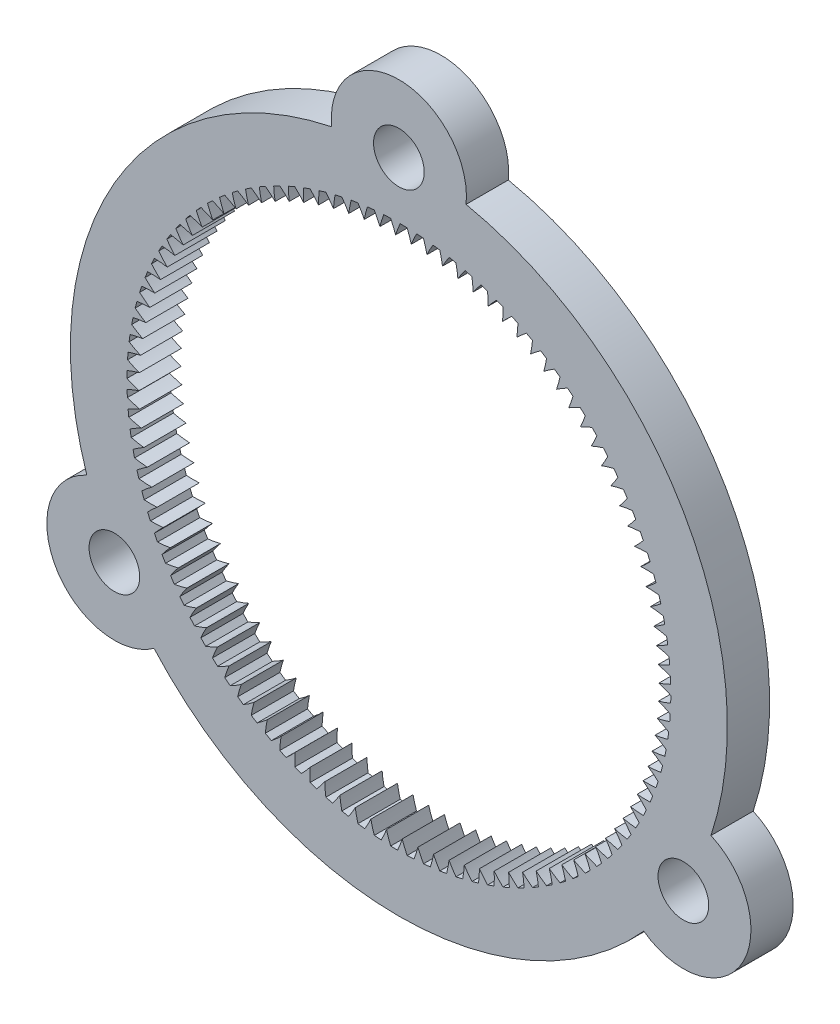
SolidWorks part; units mm, degrees
material "PLA"
ref_plane "Front" through (0, 0, 0) normal (0, 0, 1) x (1, 0, 0)
ref_plane "Top" through (0, 0, 0) normal (0, 1, 0) x (1, 0, 0)
ref_plane "Right" through (0, 0, 0) normal (1, 0, 0) x (0, 0, -1)
other "Configuration Table"
sketch "Esquisse1" plane through (0, 0, 0) normal (0, 0, 1) x (1, 0, 0)
  line L0 (0, 0) -> (0, 19.45) construction
  circle A0 centre (0, 19.45) radius 1.5
  circle A2 centre (0, 19.45) radius 4
  circle A3 centre (0, 0) radius 19.45
  circle A4 centre (0, 0) radius 12.5
  dimension "D1" = 3
  dimension "D2" = 8
  dimension "D3" = 38.9
  dimension "D4" = 25
extrude "Boss.-Extru.1" add sketch "Esquisse1" along normal blind 2.5 contours A4 A2 A3 | A2 L0 A0 A3 | L0 A0 A3 | L0 A2 A3 A0 | A0 L0 A3 region at (3.0456, 16.0734, 0) region at (-1.8091, 17.4906, 0) region at (1.8091, 17.4906, 0) region at (-0.6285, 18.8031, 0) region at (0.6285, 18.8031, 0)
extrude "Enlèv. mat.-Extru.1" cut sketch "Esquisse1<9>" along normal up to surface (2.5 mm away) contours A0 up to face at (19.45, 0, 2.5)
sketch "Esquisse1<9>" plane through (0, 0, 0) normal (0, 0, 1) x (1, 0, 0) same geometry as "Esquisse1"
extrude "Boss.-Extru.2" add sketch "Esquisse1<10>" along normal up to surface (2.5 mm away) contours A3 A2 A0 region at (0, 21.2294, 0) up to face at (0, -0.75, 2.5)
sketch "Esquisse1<10>" plane through (0, 0, 0) normal (0, 0, 1) x (1, 0, 0) same geometry as "Esquisse1"
pattern_circular "Répétition circulaire1" count 2 every 120 about axis through (0, 0, 2.5) along (0, 0, -1) of "Enlèv. mat.-Extru.1", "Boss.-Extru.2" other way count 2
sketch "Esquisse4" plane through (0, 0, 0) normal (0, 0, -1) x (-1, 0, 0)
  line L208 (13.5526, -5.2848) -> (13.6576, -5.3257)
  line L209 (13.9233, -4.5863) -> (13.8163, -4.551)
  line L210 (13.8469, -4.4569) -> (13.9542, -4.4914)
  line L211 (14.1748, -3.7373) -> (14.0658, -3.7085)
  line L212 (14.0908, -3.6127) -> (14.1999, -3.6407)
  line L213 (14.3746, -2.8746) -> (14.2641, -2.8525)
  line L214 (14.2832, -2.7553) -> (14.3938, -2.7767)
  line L215 (14.5219, -2.0014) -> (14.4103, -1.9861)
  line L216 (14.4235, -1.8879) -> (14.5352, -1.9025)
  line L217 (14.6163, -1.121) -> (14.5039, -1.1124)
  line L218 (14.5112, -1.0136) -> (14.6236, -1.0214)
  line L219 (14.6573, -0.2364) -> (14.5446, -0.2346)
  line L220 (14.5459, -0.1356) -> (14.6586, -0.1366)
  line L221 (14.6448, 0.649) -> (14.5322, 0.644)
  line L222 (14.5275, 0.7429) -> (14.6401, 0.7487)
  line L223 (14.5789, 1.532) -> (14.4669, 1.5203)
  line L224 (14.4562, 1.6187) -> (14.5682, 1.6313)
  line L225 (14.4598, 2.4095) -> (14.3487, 2.391)
  line L226 (14.3321, 2.4886) -> (14.4431, 2.5079)
  line L227 (14.288, 3.2782) -> (14.1781, 3.253)
  line L228 (14.1556, 3.3494) -> (14.2653, 3.3754)
  line L229 (14.064, 4.1349) -> (13.9558, 4.1031)
  line L230 (13.9276, 4.198) -> (14.0355, 4.2305)
  line L231 (13.7886, 4.9765) -> (13.6826, 4.9382)
  line L232 (13.6487, 5.0313) -> (13.7544, 5.0703)
  line L233 (13.463, 5.8) -> (13.3595, 5.7554)
  line L234 (13.32, 5.8462) -> (13.4232, 5.8915)
  line L235 (13.0883, 6.6022) -> (12.9876, 6.5515)
  line L236 (12.9427, 6.6398) -> (13.043, 6.6912)
  line L237 (12.6658, 7.3804) -> (12.5684, 7.3237)
  line L238 (12.5182, 7.4091) -> (12.6152, 7.4665)
  line L239 (12.197, 8.1317) -> (12.1033, 8.0692)
  line L240 (12.048, 8.1514) -> (12.1414, 8.2146)
  line L241 (11.6838, 8.8533) -> (11.594, 8.7853)
  line L242 (11.5339, 8.864) -> (11.6232, 8.9327)
  line L243 (11.1279, 9.5426) -> (11.0424, 9.4693)
  line L244 (10.9776, 9.5442) -> (11.0627, 9.6182)
  line L245 (10.5315, 10.1971) -> (10.4505, 10.1187)
  line L246 (10.3813, 10.1896) -> (10.4618, 10.2686)
  line L247 (9.8966, 10.8144) -> (9.8205, 10.7312)
  line L248 (9.7472, 10.7979) -> (9.8227, 10.8815)
  line L249 (9.2255, 11.3922) -> (9.1546, 11.3046)
  line L250 (9.0774, 11.3667) -> (9.1478, 11.4547)
  line L251 (8.5209, 11.9284) -> (8.4554, 11.8367)
  line L252 (8.3746, 11.894) -> (8.4394, 11.9862)
  line L253 (7.7851, 12.4211) -> (7.7253, 12.3256)
  line L254 (7.6411, 12.378) -> (7.7003, 12.4739)
  line L255 (7.0209, 12.8685) -> (6.967, 12.7696)
  line L256 (6.8798, 12.8167) -> (6.9331, 12.916)
  line L257 (6.2311, 13.269) -> (6.1832, 13.167)
  line L258 (6.0934, 13.2087) -> (6.1406, 13.3111)
  line L259 (5.4186, 13.621) -> (5.377, 13.5163)
  line L260 (5.2848, 13.5526) -> (5.3257, 13.6576)
  line L261 (4.5863, 13.9233) -> (4.551, 13.8163)
  line L262 (4.4569, 13.8469) -> (4.4914, 13.9542)
  line L263 (3.7373, 14.1748) -> (3.7085, 14.0658)
  line L264 (3.6127, 14.0908) -> (3.6407, 14.1999)
  line L265 (2.8746, 14.3746) -> (2.8525, 14.2641)
  line L266 (2.7553, 14.2832) -> (2.7767, 14.3938)
  line L267 (2.0014, 14.5219) -> (1.9861, 14.4103)
  line L268 (1.8879, 14.4235) -> (1.9025, 14.5352)
  line L269 (1.121, 14.6163) -> (1.1124, 14.5039)
  line L270 (1.0136, 14.5112) -> (1.0214, 14.6236)
  line L271 (0.2364, 14.6573) -> (0.2346, 14.5446)
  line L272 (0.1356, 14.5459) -> (0.1366, 14.6586)
  line L273 (-0.649, 14.6448) -> (-0.644, 14.5322)
  line L274 (-0.7429, 14.5275) -> (-0.7487, 14.6401)
  line L275 (-1.532, 14.5789) -> (-1.5203, 14.4669)
  line L276 (-1.6187, 14.4562) -> (-1.6313, 14.5682)
  line L277 (-2.4095, 14.4598) -> (-2.391, 14.3487)
  line L278 (-2.4886, 14.3321) -> (-2.5079, 14.4431)
  line L279 (-3.2782, 14.288) -> (-3.253, 14.1781)
  line L280 (-3.3494, 14.1556) -> (-3.3754, 14.2653)
  line L281 (-4.1349, 14.064) -> (-4.1031, 13.9558)
  line L282 (-4.198, 13.9276) -> (-4.2305, 14.0355)
  line L283 (-4.9765, 13.7886) -> (-4.9382, 13.6826)
  line L284 (-5.0313, 13.6487) -> (-5.0703, 13.7544)
  line L285 (-5.8, 13.463) -> (-5.7554, 13.3595)
  line L286 (-5.8462, 13.32) -> (-5.8915, 13.4232)
  line L287 (-6.6022, 13.0883) -> (-6.5515, 12.9876)
  line L288 (-6.6398, 12.9427) -> (-6.6912, 13.043)
  line L289 (-7.3804, 12.6658) -> (-7.3237, 12.5684)
  line L290 (-7.4091, 12.5182) -> (-7.4665, 12.6152)
  line L291 (-8.1317, 12.197) -> (-8.0692, 12.1033)
  line L292 (-8.1514, 12.048) -> (-8.2146, 12.1414)
  line L293 (-8.8533, 11.6838) -> (-8.7853, 11.594)
  line L294 (-8.864, 11.5339) -> (-8.9327, 11.6232)
  line L295 (-9.5426, 11.1279) -> (-9.4693, 11.0424)
  line L296 (-9.5442, 10.9776) -> (-9.6182, 11.0627)
  line L297 (-10.1971, 10.5315) -> (-10.1187, 10.4505)
  line L298 (-10.1896, 10.3813) -> (-10.2686, 10.4618)
  line L299 (-10.8144, 9.8966) -> (-10.7312, 9.8205)
  line L300 (-10.7979, 9.7472) -> (-10.8815, 9.8227)
  line L301 (-11.3922, 9.2255) -> (-11.3046, 9.1546)
  line L302 (-11.3667, 9.0774) -> (-11.4547, 9.1478)
  line L303 (-11.9284, 8.5209) -> (-11.8367, 8.4554)
  line L304 (-11.894, 8.3746) -> (-11.9862, 8.4394)
  line L305 (-12.4211, 7.7851) -> (-12.3256, 7.7253)
  line L306 (-12.378, 7.6411) -> (-12.4739, 7.7003)
  line L307 (-12.8685, 7.0209) -> (-12.7696, 6.967)
  line L308 (-12.8167, 6.8798) -> (-12.916, 6.9331)
  line L309 (-13.269, 6.2311) -> (-13.167, 6.1832)
  line L310 (-13.2087, 6.0934) -> (-13.3111, 6.1406)
  line L311 (-13.621, 5.4186) -> (-13.5163, 5.377)
  line L312 (-13.5526, 5.2848) -> (-13.6576, 5.3257)
  line L313 (-13.9233, 4.5863) -> (-13.8163, 4.551)
  line L314 (-13.8469, 4.4569) -> (-13.9542, 4.4914)
  line L315 (-14.1748, 3.7373) -> (-14.0658, 3.7085)
  line L316 (-14.0908, 3.6127) -> (-14.1999, 3.6407)
  line L317 (-14.3746, 2.8746) -> (-14.2641, 2.8525)
  line L318 (-14.2832, 2.7553) -> (-14.3938, 2.7767)
  line L319 (-14.5219, 2.0014) -> (-14.4103, 1.9861)
  line L320 (-14.4235, 1.8879) -> (-14.5352, 1.9025)
  line L321 (-14.6163, 1.121) -> (-14.5039, 1.1124)
  line L322 (-14.5112, 1.0136) -> (-14.6236, 1.0214)
  line L323 (-14.6573, 0.2364) -> (-14.5446, 0.2346)
  line L324 (-14.5459, 0.1356) -> (-14.6586, 0.1366)
  line L325 (-14.6448, -0.649) -> (-14.5322, -0.644)
  line L326 (-14.5275, -0.7429) -> (-14.6401, -0.7487)
  line L327 (-14.5789, -1.532) -> (-14.4669, -1.5203)
  line L328 (-14.4562, -1.6187) -> (-14.5682, -1.6313)
  line L329 (-14.4598, -2.4095) -> (-14.3487, -2.391)
  line L330 (-14.3321, -2.4886) -> (-14.4431, -2.5079)
  line L331 (-14.288, -3.2782) -> (-14.1781, -3.253)
  line L332 (-14.1556, -3.3494) -> (-14.2653, -3.3754)
  line L333 (-14.064, -4.1349) -> (-13.9558, -4.1031)
  line L334 (-13.9276, -4.198) -> (-14.0355, -4.2305)
  line L335 (-13.7886, -4.9765) -> (-13.6826, -4.9382)
  line L336 (-13.6487, -5.0313) -> (-13.7544, -5.0703)
  line L337 (-13.463, -5.8) -> (-13.3595, -5.7554)
  line L338 (-13.32, -5.8462) -> (-13.4232, -5.8915)
  line L339 (-13.0883, -6.6022) -> (-12.9876, -6.5515)
  line L340 (-12.9427, -6.6398) -> (-13.043, -6.6912)
  line L341 (-12.6658, -7.3804) -> (-12.5684, -7.3237)
  line L342 (-12.5182, -7.4091) -> (-12.6152, -7.4665)
  line L343 (-12.197, -8.1317) -> (-12.1033, -8.0692)
  line L344 (-12.048, -8.1514) -> (-12.1414, -8.2146)
  line L345 (-11.6838, -8.8533) -> (-11.594, -8.7853)
  line L346 (-11.5339, -8.864) -> (-11.6232, -8.9327)
  line L347 (-11.1279, -9.5426) -> (-11.0424, -9.4693)
  line L348 (-10.9776, -9.5442) -> (-11.0627, -9.6182)
  line L349 (-10.5315, -10.1971) -> (-10.4505, -10.1187)
  line L350 (-10.3813, -10.1896) -> (-10.4618, -10.2686)
  line L351 (-9.8966, -10.8144) -> (-9.8205, -10.7312)
  line L352 (-9.7472, -10.7979) -> (-9.8227, -10.8815)
  line L353 (-9.2255, -11.3922) -> (-9.1546, -11.3046)
  line L354 (-9.0774, -11.3667) -> (-9.1478, -11.4547)
  line L355 (-8.5209, -11.9284) -> (-8.4554, -11.8367)
  line L356 (-8.3746, -11.894) -> (-8.4394, -11.9862)
  line L357 (-7.7851, -12.4211) -> (-7.7253, -12.3256)
  line L358 (-7.6411, -12.378) -> (-7.7003, -12.4739)
  line L359 (-7.0209, -12.8685) -> (-6.967, -12.7696)
  line L360 (-6.8798, -12.8167) -> (-6.9331, -12.916)
  line L361 (-6.2311, -13.269) -> (-6.1832, -13.167)
  line L362 (-6.0934, -13.2087) -> (-6.1406, -13.3111)
  line L363 (-5.4186, -13.621) -> (-5.377, -13.5163)
  line L364 (-5.2848, -13.5526) -> (-5.3257, -13.6576)
  line L365 (-4.5863, -13.9233) -> (-4.551, -13.8163)
  line L366 (-4.4569, -13.8469) -> (-4.4914, -13.9542)
  line L367 (-3.7373, -14.1748) -> (-3.7085, -14.0658)
  line L368 (-3.6127, -14.0908) -> (-3.6407, -14.1999)
  line L369 (-2.8746, -14.3746) -> (-2.8525, -14.2641)
  line L370 (-2.7553, -14.2832) -> (-2.7767, -14.3938)
  line L371 (-2.0014, -14.5219) -> (-1.9861, -14.4103)
  line L372 (-1.8879, -14.4235) -> (-1.9025, -14.5352)
  line L373 (-1.121, -14.6163) -> (-1.1124, -14.5039)
  line L374 (-1.0136, -14.5112) -> (-1.0214, -14.6236)
  line L375 (-0.2364, -14.6573) -> (-0.2346, -14.5446)
  line L376 (-0.1356, -14.5459) -> (-0.1366, -14.6586)
  line L377 (0.649, -14.6448) -> (0.644, -14.5322)
  line L378 (0.7429, -14.5275) -> (0.7487, -14.6401)
  line L379 (1.532, -14.5789) -> (1.5203, -14.4669)
  line L380 (1.6187, -14.4562) -> (1.6313, -14.5682)
  line L381 (2.4095, -14.4598) -> (2.391, -14.3487)
  line L382 (2.4886, -14.3321) -> (2.5079, -14.4431)
  line L383 (3.2782, -14.288) -> (3.253, -14.1781)
  line L384 (3.3494, -14.1556) -> (3.3754, -14.2653)
  line L385 (4.1349, -14.064) -> (4.1031, -13.9558)
  line L386 (4.198, -13.9276) -> (4.2305, -14.0355)
  line L387 (4.9765, -13.7886) -> (4.9382, -13.6826)
  line L388 (5.0313, -13.6487) -> (5.0703, -13.7544)
  line L389 (5.8, -13.463) -> (5.7554, -13.3595)
  line L390 (5.8462, -13.32) -> (5.8915, -13.4232)
  line L391 (6.6022, -13.0883) -> (6.5515, -12.9876)
  line L392 (6.6398, -12.9427) -> (6.6912, -13.043)
  line L393 (7.3804, -12.6658) -> (7.3237, -12.5684)
  line L394 (7.4091, -12.5182) -> (7.4665, -12.6152)
  line L395 (8.1317, -12.197) -> (8.0692, -12.1033)
  line L396 (8.1514, -12.048) -> (8.2146, -12.1414)
  line L397 (8.8533, -11.6838) -> (8.7853, -11.594)
  line L398 (8.864, -11.5339) -> (8.9327, -11.6232)
  line L399 (9.5426, -11.1279) -> (9.4693, -11.0424)
  line L400 (9.5442, -10.9776) -> (9.6182, -11.0627)
  line L401 (10.1971, -10.5315) -> (10.1187, -10.4505)
  line L402 (10.1896, -10.3813) -> (10.2686, -10.4618)
  line L403 (10.8144, -9.8966) -> (10.7312, -9.8205)
  line L404 (10.7979, -9.7472) -> (10.8815, -9.8227)
  line L405 (11.3922, -9.2255) -> (11.3046, -9.1546)
  line L406 (11.3667, -9.0774) -> (11.4547, -9.1478)
  line L407 (11.9284, -8.5209) -> (11.8367, -8.4554)
  line L408 (11.894, -8.3746) -> (11.9862, -8.4394)
  line L409 (12.4211, -7.7851) -> (12.3256, -7.7253)
  line L410 (12.378, -7.6411) -> (12.4739, -7.7003)
  line L411 (12.8685, -7.0209) -> (12.7696, -6.967)
  line L412 (12.8167, -6.8798) -> (12.916, -6.9331)
  line L413 (13.269, -6.2311) -> (13.167, -6.1832)
  line L414 (13.2087, -6.0934) -> (13.3111, -6.1406)
  line L415 (13.621, -5.4186) -> (13.5163, -5.377)
  line L416 (13.5526, -5.2848) -> (13.6576, -5.3257)
  line L417 (13.9233, -4.5863) -> (13.8163, -4.551)
  line L418 (13.8469, -4.4569) -> (13.9542, -4.4914)
  line L419 (14.1748, -3.7373) -> (14.0658, -3.7085)
  line L420 (14.0908, -3.6127) -> (14.1999, -3.6407)
  line L421 (14.3746, -2.8746) -> (14.2641, -2.8525)
  line L422 (14.2832, -2.7553) -> (14.3938, -2.7767)
  line L423 (14.5219, -2.0014) -> (14.4103, -1.9861)
  line L424 (14.4235, -1.8879) -> (14.5352, -1.9025)
  line L425 (14.6163, -1.121) -> (14.5039, -1.1124)
  line L426 (14.5112, -1.0136) -> (14.6236, -1.0214)
  line L427 (14.6573, -0.2364) -> (14.5446, -0.2346)
  line L428 (14.5459, -0.1356) -> (14.6586, -0.1366)
  line L429 (14.6448, 0.649) -> (14.5322, 0.644)
  line L430 (14.5275, 0.7429) -> (14.6401, 0.7487)
  line L431 (14.5789, 1.532) -> (14.4669, 1.5203)
  line L432 (14.4562, 1.6187) -> (14.5682, 1.6313)
  line L433 (14.4598, 2.4095) -> (14.3487, 2.391)
  line L434 (14.3321, 2.4886) -> (14.4431, 2.5079)
  line L435 (14.288, 3.2782) -> (14.1781, 3.253)
  line L436 (14.1556, 3.3494) -> (14.2653, 3.3754)
  line L437 (14.064, 4.1349) -> (13.9558, 4.1031)
  line L438 (13.9276, 4.198) -> (14.0355, 4.2305)
  line L439 (13.7886, 4.9765) -> (13.6826, 4.9382)
  line L440 (13.6487, 5.0313) -> (13.7544, 5.0703)
  line L441 (13.463, 5.8) -> (13.3595, 5.7554)
  line L442 (13.32, 5.8462) -> (13.4232, 5.8915)
  line L443 (13.0883, 6.6022) -> (12.9876, 6.5515)
  line L444 (12.9427, 6.6398) -> (13.043, 6.6912)
  line L445 (12.6658, 7.3804) -> (12.5684, 7.3237)
  line L446 (12.5182, 7.4091) -> (12.6152, 7.4665)
  line L447 (12.197, 8.1317) -> (12.1033, 8.0692)
  line L448 (12.048, 8.1514) -> (12.1414, 8.2146)
  line L449 (11.6838, 8.8533) -> (11.594, 8.7853)
  line L450 (11.5339, 8.864) -> (11.6232, 8.9327)
  line L451 (11.1279, 9.5426) -> (11.0424, 9.4693)
  line L452 (10.9776, 9.5442) -> (11.0627, 9.6182)
  line L453 (10.5315, 10.1971) -> (10.4505, 10.1187)
  line L454 (10.3813, 10.1896) -> (10.4618, 10.2686)
  line L455 (9.8966, 10.8144) -> (9.8205, 10.7312)
  line L456 (9.7472, 10.7979) -> (9.8227, 10.8815)
  line L457 (9.2255, 11.3922) -> (9.1546, 11.3046)
  line L458 (9.0774, 11.3667) -> (9.1478, 11.4547)
  line L459 (8.5209, 11.9284) -> (8.4554, 11.8367)
  line L460 (8.3746, 11.894) -> (8.4394, 11.9862)
  line L461 (7.7851, 12.4211) -> (7.7253, 12.3256)
  line L462 (7.6411, 12.378) -> (7.7003, 12.4739)
  line L463 (7.0209, 12.8685) -> (6.967, 12.7696)
  line L464 (6.8798, 12.8167) -> (6.9331, 12.916)
  line L465 (6.2311, 13.269) -> (6.1832, 13.167)
  line L466 (6.0934, 13.2087) -> (6.1406, 13.3111)
  line L467 (5.4186, 13.621) -> (5.377, 13.5163)
  line L468 (5.2848, 13.5526) -> (5.3257, 13.6576)
  line L469 (4.5863, 13.9233) -> (4.551, 13.8163)
  line L470 (4.4569, 13.8469) -> (4.4914, 13.9542)
  line L471 (3.7373, 14.1748) -> (3.7085, 14.0658)
  line L472 (3.6127, 14.0908) -> (3.6407, 14.1999)
  line L473 (2.8746, 14.3746) -> (2.8525, 14.2641)
  line L474 (2.7553, 14.2832) -> (2.7767, 14.3938)
  line L475 (2.0014, 14.5219) -> (1.9861, 14.4103)
  line L476 (1.8879, 14.4235) -> (1.9025, 14.5352)
  line L477 (1.121, 14.6163) -> (1.1124, 14.5039)
  line L478 (1.0136, 14.5112) -> (1.0214, 14.6236)
  line L479 (0.2364, 14.6573) -> (0.2346, 14.5446)
  line L480 (0.1356, 14.5459) -> (0.1366, 14.6586)
  line L481 (-0.649, 14.6448) -> (-0.644, 14.5322)
  line L482 (-0.7429, 14.5275) -> (-0.7487, 14.6401)
  line L483 (-1.532, 14.5789) -> (-1.5203, 14.4669)
  line L484 (-1.6187, 14.4562) -> (-1.6313, 14.5682)
  line L485 (-2.4095, 14.4598) -> (-2.391, 14.3487)
  line L486 (-2.4886, 14.3321) -> (-2.5079, 14.4431)
  line L487 (-3.2782, 14.288) -> (-3.253, 14.1781)
  line L488 (-3.3494, 14.1556) -> (-3.3754, 14.2653)
  line L489 (-4.1349, 14.064) -> (-4.1031, 13.9558)
  line L490 (-4.198, 13.9276) -> (-4.2305, 14.0355)
  line L491 (-4.9765, 13.7886) -> (-4.9382, 13.6826)
  line L492 (-5.0313, 13.6487) -> (-5.0703, 13.7544)
  line L493 (-5.8, 13.463) -> (-5.7554, 13.3595)
  line L494 (-5.8462, 13.32) -> (-5.8915, 13.4232)
  line L495 (-6.6022, 13.0883) -> (-6.5515, 12.9876)
  line L496 (-6.6398, 12.9427) -> (-6.6912, 13.043)
  line L497 (-7.3804, 12.6658) -> (-7.3237, 12.5684)
  line L498 (-7.4091, 12.5182) -> (-7.4665, 12.6152)
  line L499 (-8.1317, 12.197) -> (-8.0692, 12.1033)
  line L500 (-8.1514, 12.048) -> (-8.2146, 12.1414)
  line L501 (-8.8533, 11.6838) -> (-8.7853, 11.594)
  line L502 (-8.864, 11.5339) -> (-8.9327, 11.6232)
  line L503 (-9.5426, 11.1279) -> (-9.4693, 11.0424)
  line L504 (-9.5442, 10.9776) -> (-9.6182, 11.0627)
  line L505 (-10.1971, 10.5315) -> (-10.1187, 10.4505)
  line L506 (-10.1896, 10.3813) -> (-10.2686, 10.4618)
  line L507 (-10.8144, 9.8966) -> (-10.7312, 9.8205)
  line L508 (-10.7979, 9.7472) -> (-10.8815, 9.8227)
  line L509 (-11.3922, 9.2255) -> (-11.3046, 9.1546)
  line L510 (-11.3667, 9.0774) -> (-11.4547, 9.1478)
  line L511 (-11.9284, 8.5209) -> (-11.8367, 8.4554)
  line L512 (-11.894, 8.3746) -> (-11.9862, 8.4394)
  line L513 (-12.4211, 7.7851) -> (-12.3256, 7.7253)
  line L514 (-12.378, 7.6411) -> (-12.4739, 7.7003)
  line L515 (-12.8685, 7.0209) -> (-12.7696, 6.967)
  line L516 (-12.8167, 6.8798) -> (-12.916, 6.9331)
  line L517 (-13.269, 6.2311) -> (-13.167, 6.1832)
  line L518 (-13.2087, 6.0934) -> (-13.3111, 6.1406)
  line L519 (-13.621, 5.4186) -> (-13.5163, 5.377)
  line L520 (-13.5526, 5.2848) -> (-13.6576, 5.3257)
  line L521 (-13.9233, 4.5863) -> (-13.8163, 4.551)
  line L522 (-13.8469, 4.4569) -> (-13.9542, 4.4914)
  line L523 (-14.1748, 3.7373) -> (-14.0658, 3.7085)
  line L524 (-14.0908, 3.6127) -> (-14.1999, 3.6407)
  line L525 (-14.3746, 2.8746) -> (-14.2641, 2.8525)
  line L526 (-14.2832, 2.7553) -> (-14.3938, 2.7767)
  line L527 (-14.5219, 2.0014) -> (-14.4103, 1.9861)
  line L528 (-14.4235, 1.8879) -> (-14.5352, 1.9025)
  line L529 (-14.6163, 1.121) -> (-14.5039, 1.1124)
  line L530 (-14.5112, 1.0136) -> (-14.6236, 1.0214)
  line L531 (-14.6573, 0.2364) -> (-14.5446, 0.2346)
  line L532 (-14.5459, 0.1356) -> (-14.6586, 0.1366)
  line L533 (-14.6448, -0.649) -> (-14.5322, -0.644)
  line L534 (-14.5275, -0.7429) -> (-14.6401, -0.7487)
  line L535 (-14.5789, -1.532) -> (-14.4669, -1.5203)
  line L536 (-14.4562, -1.6187) -> (-14.5682, -1.6313)
  line L537 (-14.4598, -2.4095) -> (-14.3487, -2.391)
  line L538 (-14.3321, -2.4886) -> (-14.4431, -2.5079)
  line L539 (-14.288, -3.2782) -> (-14.1781, -3.253)
  line L540 (-14.1556, -3.3494) -> (-14.2653, -3.3754)
  line L541 (-14.064, -4.1349) -> (-13.9558, -4.1031)
  line L542 (-13.9276, -4.198) -> (-14.0355, -4.2305)
  line L543 (-13.7886, -4.9765) -> (-13.6826, -4.9382)
  line L544 (-13.6487, -5.0313) -> (-13.7544, -5.0703)
  line L545 (-13.463, -5.8) -> (-13.3595, -5.7554)
  line L546 (-13.32, -5.8462) -> (-13.4232, -5.8915)
  line L547 (-13.0883, -6.6022) -> (-12.9876, -6.5515)
  line L548 (-12.9427, -6.6398) -> (-13.043, -6.6912)
  line L549 (-12.6658, -7.3804) -> (-12.5684, -7.3237)
  line L550 (-12.5182, -7.4091) -> (-12.6152, -7.4665)
  line L551 (-12.197, -8.1317) -> (-12.1033, -8.0692)
  line L552 (-12.048, -8.1514) -> (-12.1414, -8.2146)
  line L553 (-11.6838, -8.8533) -> (-11.594, -8.7853)
  line L554 (-11.5339, -8.864) -> (-11.6232, -8.9327)
  line L555 (-11.1279, -9.5426) -> (-11.0424, -9.4693)
  line L556 (-10.9776, -9.5442) -> (-11.0627, -9.6182)
  line L557 (-10.5315, -10.1971) -> (-10.4505, -10.1187)
  line L558 (-10.3813, -10.1896) -> (-10.4618, -10.2686)
  line L559 (-9.8966, -10.8144) -> (-9.8205, -10.7312)
  line L560 (-9.7472, -10.7979) -> (-9.8227, -10.8815)
  line L561 (-9.2255, -11.3922) -> (-9.1546, -11.3046)
  line L562 (-9.0774, -11.3667) -> (-9.1478, -11.4547)
  line L563 (-8.5209, -11.9284) -> (-8.4554, -11.8367)
  line L564 (-8.3746, -11.894) -> (-8.4394, -11.9862)
  line L565 (-7.7851, -12.4211) -> (-7.7253, -12.3256)
  line L566 (-7.6411, -12.378) -> (-7.7003, -12.4739)
  line L567 (-7.0209, -12.8685) -> (-6.967, -12.7696)
  line L568 (-6.8798, -12.8167) -> (-6.9331, -12.916)
  line L569 (-6.2311, -13.269) -> (-6.1832, -13.167)
  line L570 (-6.0934, -13.2087) -> (-6.1406, -13.3111)
  line L571 (-5.4186, -13.621) -> (-5.377, -13.5163)
  line L572 (-5.2848, -13.5526) -> (-5.3257, -13.6576)
  line L573 (-4.5863, -13.9233) -> (-4.551, -13.8163)
  line L574 (-4.4569, -13.8469) -> (-4.4914, -13.9542)
  line L575 (-3.7373, -14.1748) -> (-3.7085, -14.0658)
  line L576 (-3.6127, -14.0908) -> (-3.6407, -14.1999)
  line L577 (-2.8746, -14.3746) -> (-2.8525, -14.2641)
  line L578 (-2.7553, -14.2832) -> (-2.7767, -14.3938)
  line L579 (-2.0014, -14.5219) -> (-1.9861, -14.4103)
  line L580 (-1.8879, -14.4235) -> (-1.9025, -14.5352)
  line L581 (-1.121, -14.6163) -> (-1.1124, -14.5039)
  line L582 (-1.0136, -14.5112) -> (-1.0214, -14.6236)
  line L583 (-0.2364, -14.6573) -> (-0.2346, -14.5446)
  line L584 (-0.1356, -14.5459) -> (-0.1366, -14.6586)
  line L585 (0.649, -14.6448) -> (0.644, -14.5322)
  line L586 (0.7429, -14.5275) -> (0.7487, -14.6401)
  line L587 (1.532, -14.5789) -> (1.5203, -14.4669)
  line L588 (1.6187, -14.4562) -> (1.6313, -14.5682)
  line L589 (2.4095, -14.4598) -> (2.391, -14.3487)
  line L590 (2.4886, -14.3321) -> (2.5079, -14.4431)
  line L591 (3.2782, -14.288) -> (3.253, -14.1781)
  line L592 (3.3494, -14.1556) -> (3.3754, -14.2653)
  line L593 (4.1349, -14.064) -> (4.1031, -13.9558)
  line L594 (4.198, -13.9276) -> (4.2305, -14.0355)
  line L595 (4.9765, -13.7886) -> (4.9382, -13.6826)
  line L596 (5.0313, -13.6487) -> (5.0703, -13.7544)
  line L597 (5.8, -13.463) -> (5.7554, -13.3595)
  line L598 (5.8462, -13.32) -> (5.8915, -13.4232)
  line L599 (6.6022, -13.0883) -> (6.5515, -12.9876)
  line L600 (6.6398, -12.9427) -> (6.6912, -13.043)
  line L601 (7.3804, -12.6658) -> (7.3237, -12.5684)
  line L602 (7.4091, -12.5182) -> (7.4665, -12.6152)
  line L603 (8.1317, -12.197) -> (8.0692, -12.1033)
  line L604 (8.1514, -12.048) -> (8.2146, -12.1414)
  line L605 (8.8533, -11.6838) -> (8.7853, -11.594)
  line L606 (8.864, -11.5339) -> (8.9327, -11.6232)
  line L607 (9.5426, -11.1279) -> (9.4693, -11.0424)
  line L608 (9.5442, -10.9776) -> (9.6182, -11.0627)
  line L609 (10.1971, -10.5315) -> (10.1187, -10.4505)
  line L610 (10.1896, -10.3813) -> (10.2686, -10.4618)
  line L611 (10.8144, -9.8966) -> (10.7312, -9.8205)
  line L612 (10.7979, -9.7472) -> (10.8815, -9.8227)
  line L613 (11.3922, -9.2255) -> (11.3046, -9.1546)
  line L614 (11.3667, -9.0774) -> (11.4547, -9.1478)
  line L615 (11.9284, -8.5209) -> (11.8367, -8.4554)
  line L616 (11.894, -8.3746) -> (11.9862, -8.4394)
  line L617 (12.4211, -7.7851) -> (12.3256, -7.7253)
  line L618 (12.378, -7.6411) -> (12.4739, -7.7003)
  line L619 (12.8685, -7.0209) -> (12.7696, -6.967)
  line L620 (12.8167, -6.8798) -> (12.916, -6.9331)
  line L621 (13.269, -6.2311) -> (13.167, -6.1832)
  line L622 (13.2087, -6.0934) -> (13.3111, -6.1406)
  line L623 (13.621, -5.4186) -> (13.5163, -5.377)
  line L624 (8.128, 13.067) -> (8.128, 13.067)
  line L625 (8.128, 13.067) -> (8.128, 13.067)
  line L626 (7.3243, 13.5339) -> (7.3243, 13.5339)
  line L627 (7.3243, 13.5339) -> (7.3243, 13.5339)
  line L628 (6.4937, 13.9514) -> (6.4937, 13.9514)
  line L629 (6.4937, 13.9514) -> (6.4937, 13.9514)
  line L630 (5.6395, 14.318) -> (5.6395, 14.318)
  line L631 (5.6395, 14.318) -> (5.6395, 14.318)
  line L632 (4.7647, 14.6324) -> (4.7647, 14.6324)
  line L633 (4.7647, 14.6324) -> (4.7647, 14.6324)
  line L634 (3.8726, 14.8934) -> (3.8726, 14.8934)
  line L635 (3.8726, 14.8934) -> (3.8726, 14.8934)
  line L636 (2.9662, 15.1001) -> (2.9662, 15.1001)
  line L637 (2.9662, 15.1001) -> (2.9662, 15.1001)
  line L638 (2.0491, 15.2516) -> (2.0491, 15.2516)
  line L639 (2.0491, 15.2516) -> (2.0491, 15.2516)
  line L640 (1.1245, 15.3475) -> (1.1245, 15.3475)
  line L641 (1.1245, 15.3475) -> (1.1245, 15.3475)
  line L642 (0.1958, 15.3874) -> (0.1958, 15.3874)
  line L643 (0.1958, 15.3874) -> (0.1958, 15.3874)
  line L644 (-0.7336, 15.3712) -> (-0.7336, 15.3712)
  line L645 (-0.7336, 15.3712) -> (-0.7336, 15.3712)
  line L646 (-1.6604, 15.2988) -> (-1.6604, 15.2988)
  line L647 (-1.6604, 15.2988) -> (-1.6604, 15.2988)
  line L648 (-2.5811, 15.1707) -> (-2.5811, 15.1707)
  line L649 (-2.5811, 15.1707) -> (-2.5811, 15.1707)
  line L650 (-3.4923, 14.9871) -> (-3.4923, 14.9871)
  line L651 (-3.4923, 14.9871) -> (-3.4923, 14.9871)
  line L652 (-4.3909, 14.7489) -> (-4.3909, 14.7489)
  line L653 (-4.3909, 14.7489) -> (-4.3909, 14.7489)
  line L654 (-5.2734, 14.4569) -> (-5.2734, 14.4569)
  line L655 (-5.2734, 14.4569) -> (-5.2734, 14.4569)
  line L656 (-6.1366, 14.1121) -> (-6.1366, 14.1121)
  line L657 (-6.1366, 14.1121) -> (-6.1366, 14.1121)
  line L658 (-6.9775, 13.7159) -> (-6.9775, 13.7159)
  line L659 (-6.9775, 13.7159) -> (-6.9775, 13.7159)
  line L660 (-7.7929, 13.2695) -> (-7.7929, 13.2695)
  line L661 (-7.7929, 13.2695) -> (-7.7929, 13.2695)
  line L662 (-8.5799, 12.7748) -> (-8.5799, 12.7748)
  line L663 (-8.5799, 12.7748) -> (-8.5799, 12.7748)
  line L664 (-9.3356, 12.2335) -> (-9.3356, 12.2335)
  line L665 (-9.3356, 12.2335) -> (-9.3356, 12.2335)
  line L666 (-10.0572, 11.6475) -> (-10.0572, 11.6475)
  line L667 (-10.0572, 11.6475) -> (-10.0572, 11.6475)
  line L668 (-10.7421, 11.019) -> (-10.7421, 11.019)
  line L669 (-10.7421, 11.019) -> (-10.7421, 11.019)
  line L670 (-11.3878, 10.3503) -> (-11.3878, 10.3503)
  line L671 (-11.3878, 10.3503) -> (-11.3878, 10.3503)
  line L672 (-11.992, 9.6438) -> (-11.992, 9.6438)
  line L673 (-11.992, 9.6438) -> (-11.992, 9.6438)
  line L674 (-12.5524, 8.9022) -> (-12.5524, 8.9022)
  line L675 (-12.5524, 8.9022) -> (-12.5524, 8.9022)
  line L676 (-13.067, 8.128) -> (-13.067, 8.128)
  line L677 (-13.067, 8.128) -> (-13.067, 8.128)
  line L678 (-13.5339, 7.3243) -> (-13.5339, 7.3243)
  line L679 (-13.5339, 7.3243) -> (-13.5339, 7.3243)
  line L680 (-13.9514, 6.4937) -> (-13.9514, 6.4937)
  line L681 (-13.9514, 6.4937) -> (-13.9514, 6.4937)
  line L682 (-14.318, 5.6395) -> (-14.318, 5.6395)
  line L683 (-14.318, 5.6395) -> (-14.318, 5.6395)
  line L684 (-14.6324, 4.7647) -> (-14.6324, 4.7647)
  line L685 (-14.6324, 4.7647) -> (-14.6324, 4.7647)
  line L686 (-14.8934, 3.8726) -> (-14.8934, 3.8726)
  line L687 (-14.8934, 3.8726) -> (-14.8934, 3.8726)
  line L688 (-15.1001, 2.9662) -> (-15.1001, 2.9662)
  line L689 (-15.1001, 2.9662) -> (-15.1001, 2.9662)
  line L690 (-15.2516, 2.0491) -> (-15.2516, 2.0491)
  line L691 (-15.2516, 2.0491) -> (-15.2516, 2.0491)
  line L692 (-15.3475, 1.1245) -> (-15.3475, 1.1245)
  line L693 (-15.3475, 1.1245) -> (-15.3475, 1.1245)
  line L694 (-15.3874, 0.1958) -> (-15.3874, 0.1958)
  line L695 (-15.3874, 0.1958) -> (-15.3874, 0.1958)
  line L696 (-15.3712, -0.7336) -> (-15.3712, -0.7336)
  line L697 (-15.3712, -0.7336) -> (-15.3712, -0.7336)
  line L698 (-15.2988, -1.6604) -> (-15.2988, -1.6604)
  line L699 (-15.2988, -1.6604) -> (-15.2988, -1.6604)
  line L700 (-15.1707, -2.5811) -> (-15.1707, -2.5811)
  line L701 (-15.1707, -2.5811) -> (-15.1707, -2.5811)
  line L702 (-14.9871, -3.4923) -> (-14.9871, -3.4923)
  line L703 (-14.9871, -3.4923) -> (-14.9871, -3.4923)
  line L704 (-14.7489, -4.3909) -> (-14.7489, -4.3909)
  line L705 (-14.7489, -4.3909) -> (-14.7489, -4.3909)
  line L706 (-14.4569, -5.2734) -> (-14.4569, -5.2734)
  line L707 (-14.4569, -5.2734) -> (-14.4569, -5.2734)
  line L708 (-14.1121, -6.1366) -> (-14.1121, -6.1366)
  line L709 (-14.1121, -6.1366) -> (-14.1121, -6.1366)
  line L710 (-13.7159, -6.9775) -> (-13.7159, -6.9775)
  line L711 (-13.7159, -6.9775) -> (-13.7159, -6.9775)
  line L712 (-13.2695, -7.7929) -> (-13.2695, -7.7929)
  line L713 (-13.2695, -7.7929) -> (-13.2695, -7.7929)
  line L714 (-12.7748, -8.5799) -> (-12.7748, -8.5799)
  line L715 (-12.7748, -8.5799) -> (-12.7748, -8.5799)
  line L716 (-12.2335, -9.3356) -> (-12.2335, -9.3356)
  line L717 (-12.2335, -9.3356) -> (-12.2335, -9.3356)
  line L718 (-11.6475, -10.0572) -> (-11.6475, -10.0572)
  line L719 (-11.6475, -10.0572) -> (-11.6475, -10.0572)
  line L720 (-11.019, -10.7421) -> (-11.019, -10.7421)
  line L721 (-11.019, -10.7421) -> (-11.019, -10.7421)
  line L722 (-10.3503, -11.3878) -> (-10.3503, -11.3878)
  line L723 (-10.3503, -11.3878) -> (-10.3503, -11.3878)
  line L724 (-9.6438, -11.992) -> (-9.6438, -11.992)
  line L725 (-9.6438, -11.992) -> (-9.6438, -11.992)
  line L726 (-8.9022, -12.5524) -> (-8.9022, -12.5524)
  line L727 (-8.9022, -12.5524) -> (-8.9022, -12.5524)
  line L728 (-8.128, -13.067) -> (-8.128, -13.067)
  line L729 (-8.128, -13.067) -> (-8.128, -13.067)
  line L730 (-7.3243, -13.5339) -> (-7.3243, -13.5339)
  line L731 (-7.3243, -13.5339) -> (-7.3243, -13.5339)
  line L732 (-6.4937, -13.9514) -> (-6.4937, -13.9514)
  line L733 (-6.4937, -13.9514) -> (-6.4937, -13.9514)
  line L734 (-5.6395, -14.318) -> (-5.6395, -14.318)
  line L735 (-5.6395, -14.318) -> (-5.6395, -14.318)
  line L736 (-4.7647, -14.6324) -> (-4.7647, -14.6324)
  line L737 (-4.7647, -14.6324) -> (-4.7647, -14.6324)
  line L738 (-3.8726, -14.8934) -> (-3.8726, -14.8934)
  line L739 (-3.8726, -14.8934) -> (-3.8726, -14.8934)
  line L740 (-2.9662, -15.1001) -> (-2.9662, -15.1001)
  line L741 (-2.9662, -15.1001) -> (-2.9662, -15.1001)
  line L742 (-2.0491, -15.2516) -> (-2.0491, -15.2516)
  line L743 (-2.0491, -15.2516) -> (-2.0491, -15.2516)
  line L744 (-1.1245, -15.3475) -> (-1.1245, -15.3475)
  line L745 (-1.1245, -15.3475) -> (-1.1245, -15.3475)
  line L746 (-0.1958, -15.3874) -> (-0.1958, -15.3874)
  line L747 (-0.1958, -15.3874) -> (-0.1958, -15.3874)
  line L748 (0.7336, -15.3712) -> (0.7336, -15.3712)
  line L749 (0.7336, -15.3712) -> (0.7336, -15.3712)
  line L750 (1.6604, -15.2988) -> (1.6604, -15.2988)
  line L751 (1.6604, -15.2988) -> (1.6604, -15.2988)
  line L752 (2.5811, -15.1707) -> (2.5811, -15.1707)
  line L753 (2.5811, -15.1707) -> (2.5811, -15.1707)
  line L754 (3.4923, -14.9871) -> (3.4923, -14.9871)
  line L755 (3.4923, -14.9871) -> (3.4923, -14.9871)
  line L756 (4.3909, -14.7489) -> (4.3909, -14.7489)
  line L757 (4.3909, -14.7489) -> (4.3909, -14.7489)
  line L758 (5.2734, -14.4569) -> (5.2734, -14.4569)
  line L759 (5.2734, -14.4569) -> (5.2734, -14.4569)
  line L760 (6.1366, -14.1121) -> (6.1366, -14.1121)
  line L761 (6.1366, -14.1121) -> (6.1366, -14.1121)
  line L762 (6.9775, -13.7159) -> (6.9775, -13.7159)
  line L763 (6.9775, -13.7159) -> (6.9775, -13.7159)
  line L764 (7.7929, -13.2695) -> (7.7929, -13.2695)
  line L765 (7.7929, -13.2695) -> (7.7929, -13.2695)
  line L766 (8.5799, -12.7748) -> (8.5799, -12.7748)
  line L767 (8.5799, -12.7748) -> (8.5799, -12.7748)
  line L768 (9.3356, -12.2335) -> (9.3356, -12.2335)
  line L769 (9.3356, -12.2335) -> (9.3356, -12.2335)
  line L770 (10.0572, -11.6475) -> (10.0572, -11.6475)
  line L771 (10.0572, -11.6475) -> (10.0572, -11.6475)
  line L772 (10.7421, -11.019) -> (10.7421, -11.019)
  line L773 (10.7421, -11.019) -> (10.7421, -11.019)
  line L774 (11.3878, -10.3503) -> (11.3878, -10.3503)
  line L775 (11.3878, -10.3503) -> (11.3878, -10.3503)
  line L776 (11.992, -9.6438) -> (11.992, -9.6438)
  line L777 (11.992, -9.6438) -> (11.992, -9.6438)
  line L778 (12.5524, -8.9022) -> (12.5524, -8.9022)
  line L779 (12.5524, -8.9022) -> (12.5524, -8.9022)
  line L780 (13.067, -8.128) -> (13.067, -8.128)
  line L781 (13.067, -8.128) -> (13.067, -8.128)
  line L782 (13.5339, -7.3243) -> (13.5339, -7.3243)
  line L783 (13.5339, -7.3243) -> (13.5339, -7.3243)
  line L784 (13.9514, -6.4937) -> (13.9514, -6.4937)
  line L785 (13.9514, -6.4937) -> (13.9514, -6.4937)
  line L786 (14.318, -5.6395) -> (14.318, -5.6395)
  line L787 (14.318, -5.6395) -> (14.318, -5.6395)
  line L788 (14.6324, -4.7647) -> (14.6324, -4.7647)
  line L789 (14.6324, -4.7647) -> (14.6324, -4.7647)
  line L790 (14.8934, -3.8726) -> (14.8934, -3.8726)
  line L791 (14.8934, -3.8726) -> (14.8934, -3.8726)
  line L792 (15.1001, -2.9662) -> (15.1001, -2.9662)
  line L793 (15.1001, -2.9662) -> (15.1001, -2.9662)
  line L794 (15.2516, -2.0491) -> (15.2516, -2.0491)
  line L795 (15.2516, -2.0491) -> (15.2516, -2.0491)
  line L796 (15.3475, -1.1245) -> (15.3475, -1.1245)
  line L797 (15.3475, -1.1245) -> (15.3475, -1.1245)
  line L798 (15.3874, -0.1958) -> (15.3874, -0.1958)
  line L799 (15.3874, -0.1958) -> (15.3874, -0.1958)
  line L800 (15.3712, 0.7336) -> (15.3712, 0.7336)
  line L801 (15.3712, 0.7336) -> (15.3712, 0.7336)
  line L802 (15.2988, 1.6604) -> (15.2988, 1.6604)
  line L803 (15.2988, 1.6604) -> (15.2988, 1.6604)
  line L804 (15.1707, 2.5811) -> (15.1707, 2.5811)
  line L805 (15.1707, 2.5811) -> (15.1707, 2.5811)
  line L806 (14.9871, 3.4923) -> (14.9871, 3.4923)
  line L807 (14.9871, 3.4923) -> (14.9871, 3.4923)
  line L808 (14.7489, 4.3909) -> (14.7489, 4.3909)
  line L809 (14.7489, 4.3909) -> (14.7489, 4.3909)
  line L810 (14.4569, 5.2734) -> (14.4569, 5.2734)
  line L811 (14.4569, 5.2734) -> (14.4569, 5.2734)
  line L812 (14.1121, 6.1366) -> (14.1121, 6.1366)
  line L813 (14.1121, 6.1366) -> (14.1121, 6.1366)
  line L814 (13.7159, 6.9775) -> (13.7159, 6.9775)
  line L815 (13.7159, 6.9775) -> (13.7159, 6.9775)
  line L816 (13.2695, 7.7929) -> (13.2695, 7.7929)
  line L817 (13.2695, 7.7929) -> (13.2695, 7.7929)
  line L818 (12.7748, 8.5799) -> (12.7748, 8.5799)
  line L819 (12.7748, 8.5799) -> (12.7748, 8.5799)
  line L820 (12.2335, 9.3356) -> (12.2335, 9.3356)
  line L821 (12.2335, 9.3356) -> (12.2335, 9.3356)
  line L822 (11.6475, 10.0572) -> (11.6475, 10.0572)
  line L823 (11.6475, 10.0572) -> (11.6475, 10.0572)
  line L824 (11.019, 10.7421) -> (11.019, 10.7421)
  line L825 (11.019, 10.7421) -> (11.019, 10.7421)
  line L826 (10.3503, 11.3878) -> (10.3503, 11.3878)
  line L827 (10.3503, 11.3878) -> (10.3503, 11.3878)
  line L828 (9.6438, 11.992) -> (9.6438, 11.992)
  line L829 (9.6438, 11.992) -> (9.6438, 11.992)
  line L830 (8.9022, 12.5524) -> (8.9022, 12.5524)
  line L831 (8.9022, 12.5524) -> (8.9022, 12.5524)
  arc A312 (13.469, -5.3051) -> (13.5163, -5.377) centre (13.544, -5.3073) ccw
  arc A313 (13.5526, -5.2848) -> (13.469, -5.3051) centre (13.5253, -5.3547) ccw
  arc A314 (14.9391, -5.4436) -> (14.9867, -5.3112) centre (0, 0) ccw
  arc A315 (13.7648, -4.4822) -> (13.8163, -4.551) centre (13.8397, -4.4798) ccw
  arc A316 (13.8469, -4.4569) -> (13.7648, -4.4822) centre (13.8239, -4.5283) ccw
  arc A317 (15.2405, -4.5316) -> (15.28, -4.3967) centre (0, 0) ccw
  arc A318 (14.0103, -3.6429) -> (14.0658, -3.7085) centre (14.085, -3.636) ccw
  arc A319 (14.0908, -3.6127) -> (14.0103, -3.6429) centre (14.0721, -3.6853) ccw
  arc A320 (15.4864, -3.6032) -> (15.5176, -3.466) centre (0, 0) ccw
  arc A321 (14.2047, -2.7904) -> (14.2641, -2.8525) centre (14.2788, -2.779) ccw
  arc A322 (14.2832, -2.7553) -> (14.2047, -2.7904) centre (14.269, -2.829) ccw
  arc A323 (15.6757, -2.6615) -> (15.6986, -2.5228) centre (0, 0) ccw
  arc A324 (14.3472, -1.9276) -> (14.4103, -1.9861) centre (14.4205, -1.9118) ccw
  arc A325 (14.4235, -1.8879) -> (14.3472, -1.9276) centre (14.4138, -1.9623) ccw
  arc A326 (15.8078, -1.7102) -> (15.8223, -1.5703) centre (0, 0) ccw
  arc A327 (14.4374, -1.0578) -> (14.5039, -1.1124) centre (14.5097, -1.0376) ccw
  arc A328 (14.5112, -1.0136) -> (14.4374, -1.0578) centre (14.5059, -1.0884) ccw
  arc A329 (15.8822, -0.7526) -> (15.8882, -0.6121) centre (0, 0) ccw
  arc A330 (14.475, -0.1842) -> (14.5446, -0.2346) centre (14.5458, -0.1596) ccw
  arc A331 (14.5459, -0.1356) -> (14.475, -0.1842) centre (14.5452, -0.2106) ccw
  arc A332 (15.8986, 0.2077) -> (15.8962, 0.3483) centre (0, 0) ccw
  arc A333 (14.4597, 0.6901) -> (14.5322, 0.644) centre (14.5289, 0.7189) ccw
  arc A334 (14.5275, 0.7429) -> (14.4597, 0.6901) centre (14.5314, 0.668) ccw
  arc A335 (15.8571, 1.1672) -> (15.8462, 1.3074) centre (0, 0) ccw
  arc A336 (14.3916, 1.5619) -> (14.4669, 1.5203) centre (14.459, 1.5949) ccw
  arc A337 (14.4562, 1.6187) -> (14.3916, 1.5619) centre (14.4645, 1.5442) ccw
  arc A338 (15.7577, 2.1225) -> (15.7383, 2.2618) centre (0, 0) ccw
  arc A339 (14.2711, 2.428) -> (14.3487, 2.391) centre (14.3363, 2.465) ccw
  arc A340 (14.3321, 2.4886) -> (14.2711, 2.428) centre (14.3449, 2.4147) ccw
  arc A341 (15.6008, 3.0701) -> (15.573, 3.2079) centre (0, 0) ccw
  arc A342 (14.0984, 3.2853) -> (14.1781, 3.253) centre (14.1614, 3.3261) ccw
  arc A343 (14.1556, 3.3494) -> (14.0984, 3.2853) centre (14.1729, 3.2764) ccw
  arc A344 (15.387, 4.0064) -> (15.3509, 4.1424) centre (0, 0) ccw
  arc A345 (13.8744, 4.1305) -> (13.9558, 4.1031) centre (13.9347, 4.175) ccw
  arc A346 (13.9276, 4.198) -> (13.8744, 4.1305) centre (13.9492, 4.1262) ccw
  arc A347 (15.117, 4.9282) -> (15.0728, 5.0617) centre (0, 0) ccw
  arc A348 (13.5996, 4.9607) -> (13.6826, 4.9382) centre (13.6572, 5.0088) ccw
  arc A349 (13.6487, 5.0313) -> (13.5996, 4.9607) centre (13.6746, 4.9609) ccw
  arc A350 (14.7918, 5.8319) -> (14.7397, 5.9625) centre (0, 0) ccw
  arc A351 (13.2753, 5.7728) -> (13.3595, 5.7554) centre (13.3298, 5.8242) ccw
  arc A352 (13.32, 5.8462) -> (13.2753, 5.7728) centre (13.3502, 5.7775) ccw
  arc A353 (14.4127, 6.7144) -> (14.3528, 6.8416) centre (0, 0) ccw
  arc A354 (12.9025, 6.5638) -> (12.9876, 6.5515) centre (12.9539, 6.6185) ccw
  arc A355 (12.9427, 6.6398) -> (12.9025, 6.5638) centre (12.977, 6.573) ccw
  arc A356 (13.981, 7.5724) -> (13.9135, 7.6957) centre (0, 0) ccw
  arc A357 (12.4827, 7.3308) -> (12.5684, 7.3237) centre (12.5306, 7.3885) ccw
  arc A358 (12.5182, 7.4091) -> (12.4827, 7.3308) centre (12.5564, 7.3446) ccw
  arc A359 (13.4983, 8.4027) -> (13.4235, 8.5217) centre (0, 0) ccw
  arc A360 (12.0173, 8.0711) -> (12.1033, 8.0692) centre (12.0617, 8.1316) ccw
  arc A361 (12.048, 8.1514) -> (12.0173, 8.0711) centre (12.0901, 8.0893) ccw
  arc A362 (12.9664, 9.2024) -> (12.8845, 9.3167) centre (0, 0) ccw
  arc A363 (11.508, 8.782) -> (11.594, 8.7853) centre (11.5487, 8.845) ccw
  arc A364 (11.5339, 8.864) -> (11.508, 8.782) centre (11.5796, 8.8045) ccw
  arc A365 (12.3871, 9.9685) -> (12.2984, 10.0776) centre (0, 0) ccw
  arc A366 (10.9568, 9.4608) -> (11.0424, 9.4693) centre (10.9936, 9.5262) ccw
  arc A367 (10.9776, 9.5442) -> (10.9568, 9.4608) centre (11.0269, 9.4876) ccw
  arc A368 (11.7626, 10.6982) -> (11.6675, 10.8018) centre (0, 0) ccw
  arc A369 (10.3656, 10.1051) -> (10.4505, 10.1187) centre (10.3983, 10.1726) ccw
  arc A370 (10.3813, 10.1896) -> (10.3656, 10.1051) centre (10.4339, 10.1361) ccw
  arc A371 (11.0952, 11.3889) -> (10.994, 11.4866) centre (0, 0) ccw
  arc A372 (9.7365, 10.7125) -> (9.8205, 10.7312) centre (9.7651, 10.7819) ccw
  arc A373 (9.7472, 10.7979) -> (9.7365, 10.7125) centre (9.8028, 10.7476) ccw
  arc A374 (10.3873, 12.038) -> (10.2804, 12.1294) centre (0, 0) ccw
  arc A375 (9.072, 11.2809) -> (9.1546, 11.3046) centre (9.0963, 11.3518) ccw
  arc A376 (9.0774, 11.3667) -> (9.072, 11.2809) centre (9.136, 11.3199) ccw
  arc A377 (9.6415, 12.6432) -> (9.5293, 12.728) centre (0, 0) ccw
  arc A378 (8.3743, 11.808) -> (8.4554, 11.8367) centre (8.3943, 11.8803) ccw
  arc A379 (8.3746, 11.894) -> (8.3743, 11.808) centre (8.4359, 11.8508) ccw
  arc A380 (8.8606, 13.2023) -> (8.7434, 13.2801) centre (0, 0) ccw
  arc A381 (7.6461, 12.2921) -> (7.7253, 12.3256) centre (7.6617, 12.3655) ccw
  arc A382 (7.6411, 12.378) -> (7.6461, 12.2921) centre (7.705, 12.3386) ccw
  arc A383 (8.0473, 13.7132) -> (7.9256, 13.7838) centre (0, 0) ccw
  arc A384 (6.8899, 12.7314) -> (6.967, 12.7696) centre (6.9011, 12.8055) ccw
  arc A385 (6.8798, 12.8167) -> (6.8899, 12.7314) centre (6.9459, 12.7813) ccw
  arc A386 (7.2046, 14.1741) -> (7.0789, 14.2372) centre (0, 0) ccw
  arc A387 (6.1087, 13.1241) -> (6.1832, 13.167) centre (6.1153, 13.1988) ccw
  arc A388 (6.0934, 13.2087) -> (6.1087, 13.1241) centre (6.1615, 13.1773) ccw
  arc A389 (6.3356, 14.5832) -> (6.2064, 14.6387) centre (0, 0) ccw
  arc A390 (5.3051, 13.469) -> (5.377, 13.5163) centre (5.3073, 13.544) ccw
  arc A391 (5.2848, 13.5526) -> (5.3051, 13.469) centre (5.3547, 13.5253) ccw
  arc A392 (5.4436, 14.9391) -> (5.3112, 14.9867) centre (0, 0) ccw
  arc A393 (4.4822, 13.7648) -> (4.551, 13.8163) centre (4.4798, 13.8397) ccw
  arc A394 (4.4569, 13.8469) -> (4.4822, 13.7648) centre (4.5283, 13.8239) ccw
  arc A395 (4.5316, 15.2405) -> (4.3967, 15.28) centre (0, 0) ccw
  arc A396 (3.6429, 14.0103) -> (3.7085, 14.0658) centre (3.636, 14.085) ccw
  arc A397 (3.6127, 14.0908) -> (3.6429, 14.0103) centre (3.6853, 14.0721) ccw
  arc A398 (3.6032, 15.4864) -> (3.466, 15.5176) centre (0, 0) ccw
  arc A399 (2.7904, 14.2047) -> (2.8525, 14.2641) centre (2.779, 14.2788) ccw
  arc A400 (2.7553, 14.2832) -> (2.7904, 14.2047) centre (2.829, 14.269) ccw
  arc A401 (2.6615, 15.6757) -> (2.5228, 15.6986) centre (0, 0) ccw
  arc A402 (1.9276, 14.3472) -> (1.9861, 14.4103) centre (1.9118, 14.4205) ccw
  arc A403 (1.8879, 14.4235) -> (1.9276, 14.3472) centre (1.9623, 14.4138) ccw
  arc A404 (1.7102, 15.8078) -> (1.5703, 15.8223) centre (0, 0) ccw
  arc A405 (1.0578, 14.4374) -> (1.1124, 14.5039) centre (1.0376, 14.5097) ccw
  arc A406 (1.0136, 14.5112) -> (1.0578, 14.4374) centre (1.0884, 14.5059) ccw
  arc A407 (0.7526, 15.8822) -> (0.6121, 15.8882) centre (0, 0) ccw
  arc A408 (0.1842, 14.475) -> (0.2346, 14.5446) centre (0.1596, 14.5458) ccw
  arc A409 (0.1356, 14.5459) -> (0.1842, 14.475) centre (0.2106, 14.5452) ccw
  arc A410 (-0.2077, 15.8986) -> (-0.3483, 15.8962) centre (0, 0) ccw
  arc A411 (-0.6901, 14.4597) -> (-0.644, 14.5322) centre (-0.7189, 14.5289) ccw
  arc A412 (-0.7429, 14.5275) -> (-0.6901, 14.4597) centre (-0.668, 14.5314) ccw
  arc A413 (-1.1672, 15.8571) -> (-1.3074, 15.8462) centre (0, 0) ccw
  arc A414 (-1.5619, 14.3916) -> (-1.5203, 14.4669) centre (-1.5949, 14.459) ccw
  arc A415 (-1.6187, 14.4562) -> (-1.5619, 14.3916) centre (-1.5442, 14.4645) ccw
  arc A416 (-2.1225, 15.7577) -> (-2.2618, 15.7383) centre (0, 0) ccw
  arc A417 (-2.428, 14.2711) -> (-2.391, 14.3487) centre (-2.465, 14.3363) ccw
  arc A418 (-2.4886, 14.3321) -> (-2.428, 14.2711) centre (-2.4147, 14.3449) ccw
  arc A419 (-3.0701, 15.6008) -> (-3.2079, 15.573) centre (0, 0) ccw
  arc A420 (-3.2853, 14.0984) -> (-3.253, 14.1781) centre (-3.3261, 14.1614) ccw
  arc A421 (-3.3494, 14.1556) -> (-3.2853, 14.0984) centre (-3.2764, 14.1729) ccw
  arc A422 (-4.0064, 15.387) -> (-4.1424, 15.3509) centre (0, 0) ccw
  arc A423 (-4.1305, 13.8744) -> (-4.1031, 13.9558) centre (-4.175, 13.9347) ccw
  arc A424 (-4.198, 13.9276) -> (-4.1305, 13.8744) centre (-4.1262, 13.9492) ccw
  arc A425 (-4.9282, 15.117) -> (-5.0617, 15.0728) centre (0, 0) ccw
  arc A426 (-4.9607, 13.5996) -> (-4.9382, 13.6826) centre (-5.0088, 13.6572) ccw
  arc A427 (-5.0313, 13.6487) -> (-4.9607, 13.5996) centre (-4.9609, 13.6746) ccw
  arc A428 (-5.8319, 14.7918) -> (-5.9625, 14.7397) centre (0, 0) ccw
  arc A429 (-5.7728, 13.2753) -> (-5.7554, 13.3595) centre (-5.8242, 13.3298) ccw
  arc A430 (-5.8462, 13.32) -> (-5.7728, 13.2753) centre (-5.7775, 13.3502) ccw
  arc A431 (-6.7144, 14.4127) -> (-6.8416, 14.3528) centre (0, 0) ccw
  arc A432 (-6.5638, 12.9025) -> (-6.5515, 12.9876) centre (-6.6185, 12.9539) ccw
  arc A433 (-6.6398, 12.9427) -> (-6.5638, 12.9025) centre (-6.573, 12.977) ccw
  arc A434 (-7.5724, 13.981) -> (-7.6957, 13.9135) centre (0, 0) ccw
  arc A435 (-7.3308, 12.4827) -> (-7.3237, 12.5684) centre (-7.3885, 12.5306) ccw
  arc A436 (-7.4091, 12.5182) -> (-7.3308, 12.4827) centre (-7.3446, 12.5564) ccw
  arc A437 (-8.4027, 13.4983) -> (-8.5217, 13.4235) centre (0, 0) ccw
  arc A438 (-8.0711, 12.0173) -> (-8.0692, 12.1033) centre (-8.1316, 12.0617) ccw
  arc A439 (-8.1514, 12.048) -> (-8.0711, 12.0173) centre (-8.0893, 12.0901) ccw
  arc A440 (-9.2024, 12.9664) -> (-9.3167, 12.8845) centre (0, 0) ccw
  arc A441 (-8.782, 11.508) -> (-8.7853, 11.594) centre (-8.845, 11.5487) ccw
  arc A442 (-8.864, 11.5339) -> (-8.782, 11.508) centre (-8.8045, 11.5796) ccw
  arc A443 (-9.9685, 12.3871) -> (-10.0776, 12.2984) centre (0, 0) ccw
  arc A444 (-9.4608, 10.9568) -> (-9.4693, 11.0424) centre (-9.5262, 10.9936) ccw
  arc A445 (-9.5442, 10.9776) -> (-9.4608, 10.9568) centre (-9.4876, 11.0269) ccw
  arc A446 (-10.6982, 11.7626) -> (-10.8018, 11.6675) centre (0, 0) ccw
  arc A447 (-10.1051, 10.3656) -> (-10.1187, 10.4505) centre (-10.1726, 10.3983) ccw
  arc A448 (-10.1896, 10.3813) -> (-10.1051, 10.3656) centre (-10.1361, 10.4339) ccw
  arc A449 (-11.3889, 11.0952) -> (-11.4866, 10.994) centre (0, 0) ccw
  arc A450 (-10.7125, 9.7365) -> (-10.7312, 9.8205) centre (-10.7819, 9.7651) ccw
  arc A451 (-10.7979, 9.7472) -> (-10.7125, 9.7365) centre (-10.7476, 9.8028) ccw
  arc A452 (-12.038, 10.3873) -> (-12.1294, 10.2804) centre (0, 0) ccw
  arc A453 (-11.2809, 9.072) -> (-11.3046, 9.1546) centre (-11.3518, 9.0963) ccw
  arc A454 (-11.3667, 9.0774) -> (-11.2809, 9.072) centre (-11.3199, 9.136) ccw
  arc A455 (-12.6432, 9.6415) -> (-12.728, 9.5293) centre (0, 0) ccw
  arc A456 (-11.808, 8.3743) -> (-11.8367, 8.4554) centre (-11.8803, 8.3943) ccw
  arc A457 (-11.894, 8.3746) -> (-11.808, 8.3743) centre (-11.8508, 8.4359) ccw
  arc A458 (-13.2023, 8.8606) -> (-13.2801, 8.7434) centre (0, 0) ccw
  arc A459 (-12.2921, 7.6461) -> (-12.3256, 7.7253) centre (-12.3655, 7.6617) ccw
  arc A460 (-12.378, 7.6411) -> (-12.2921, 7.6461) centre (-12.3386, 7.705) ccw
  arc A461 (-13.7132, 8.0473) -> (-13.7838, 7.9256) centre (0, 0) ccw
  arc A462 (-12.7314, 6.8899) -> (-12.7696, 6.967) centre (-12.8055, 6.9011) ccw
  arc A463 (-12.8167, 6.8798) -> (-12.7314, 6.8899) centre (-12.7813, 6.9459) ccw
  arc A464 (-14.1741, 7.2046) -> (-14.2372, 7.0789) centre (0, 0) ccw
  arc A465 (-13.1241, 6.1087) -> (-13.167, 6.1832) centre (-13.1988, 6.1153) ccw
  arc A466 (-13.2087, 6.0934) -> (-13.1241, 6.1087) centre (-13.1773, 6.1615) ccw
  arc A467 (-14.5832, 6.3356) -> (-14.6387, 6.2064) centre (0, 0) ccw
  arc A468 (-13.469, 5.3051) -> (-13.5163, 5.377) centre (-13.544, 5.3073) ccw
  arc A469 (-13.5526, 5.2848) -> (-13.469, 5.3051) centre (-13.5253, 5.3547) ccw
  arc A470 (-14.9391, 5.4436) -> (-14.9867, 5.3112) centre (0, 0) ccw
  arc A471 (-13.7648, 4.4822) -> (-13.8163, 4.551) centre (-13.8397, 4.4798) ccw
  arc A472 (-13.8469, 4.4569) -> (-13.7648, 4.4822) centre (-13.8239, 4.5283) ccw
  arc A473 (-15.2405, 4.5316) -> (-15.28, 4.3967) centre (0, 0) ccw
  arc A474 (-14.0103, 3.6429) -> (-14.0658, 3.7085) centre (-14.085, 3.636) ccw
  arc A475 (-14.0908, 3.6127) -> (-14.0103, 3.6429) centre (-14.0721, 3.6853) ccw
  arc A476 (-15.4864, 3.6032) -> (-15.5176, 3.466) centre (0, 0) ccw
  arc A477 (-14.2047, 2.7904) -> (-14.2641, 2.8525) centre (-14.2788, 2.779) ccw
  arc A478 (-14.2832, 2.7553) -> (-14.2047, 2.7904) centre (-14.269, 2.829) ccw
  arc A479 (-15.6757, 2.6615) -> (-15.6986, 2.5228) centre (0, 0) ccw
  arc A480 (-14.3472, 1.9276) -> (-14.4103, 1.9861) centre (-14.4205, 1.9118) ccw
  arc A481 (-14.4235, 1.8879) -> (-14.3472, 1.9276) centre (-14.4138, 1.9623) ccw
  arc A482 (-15.8078, 1.7102) -> (-15.8223, 1.5703) centre (0, 0) ccw
  arc A483 (-14.4374, 1.0578) -> (-14.5039, 1.1124) centre (-14.5097, 1.0376) ccw
  arc A484 (-14.5112, 1.0136) -> (-14.4374, 1.0578) centre (-14.5059, 1.0884) ccw
  arc A485 (-15.8822, 0.7526) -> (-15.8882, 0.6121) centre (0, 0) ccw
  arc A486 (-14.475, 0.1842) -> (-14.5446, 0.2346) centre (-14.5458, 0.1596) ccw
  arc A487 (-14.5459, 0.1356) -> (-14.475, 0.1842) centre (-14.5452, 0.2106) ccw
  arc A488 (-15.8986, -0.2077) -> (-15.8962, -0.3483) centre (0, 0) ccw
  arc A489 (-14.4597, -0.6901) -> (-14.5322, -0.644) centre (-14.5289, -0.7189) ccw
  arc A490 (-14.5275, -0.7429) -> (-14.4597, -0.6901) centre (-14.5314, -0.668) ccw
  arc A491 (-15.8571, -1.1672) -> (-15.8462, -1.3074) centre (0, 0) ccw
  arc A492 (-14.3916, -1.5619) -> (-14.4669, -1.5203) centre (-14.459, -1.5949) ccw
  arc A493 (-14.4562, -1.6187) -> (-14.3916, -1.5619) centre (-14.4645, -1.5442) ccw
  arc A494 (-15.7577, -2.1225) -> (-15.7383, -2.2618) centre (0, 0) ccw
  arc A495 (-14.2711, -2.428) -> (-14.3487, -2.391) centre (-14.3363, -2.465) ccw
  arc A496 (-14.3321, -2.4886) -> (-14.2711, -2.428) centre (-14.3449, -2.4147) ccw
  arc A497 (-15.6008, -3.0701) -> (-15.573, -3.2079) centre (0, 0) ccw
  arc A498 (-14.0984, -3.2853) -> (-14.1781, -3.253) centre (-14.1614, -3.3261) ccw
  arc A499 (-14.1556, -3.3494) -> (-14.0984, -3.2853) centre (-14.1729, -3.2764) ccw
  arc A500 (-15.387, -4.0064) -> (-15.3509, -4.1424) centre (0, 0) ccw
  arc A501 (-13.8744, -4.1305) -> (-13.9558, -4.1031) centre (-13.9347, -4.175) ccw
  arc A502 (-13.9276, -4.198) -> (-13.8744, -4.1305) centre (-13.9492, -4.1262) ccw
  arc A503 (-15.117, -4.9282) -> (-15.0728, -5.0617) centre (0, 0) ccw
  arc A504 (-13.5996, -4.9607) -> (-13.6826, -4.9382) centre (-13.6572, -5.0088) ccw
  arc A505 (-13.6487, -5.0313) -> (-13.5996, -4.9607) centre (-13.6746, -4.9609) ccw
  arc A506 (-14.7918, -5.8319) -> (-14.7397, -5.9625) centre (0, 0) ccw
  arc A507 (-13.2753, -5.7728) -> (-13.3595, -5.7554) centre (-13.3298, -5.8242) ccw
  arc A508 (-13.32, -5.8462) -> (-13.2753, -5.7728) centre (-13.3502, -5.7775) ccw
  arc A509 (-14.4127, -6.7144) -> (-14.3528, -6.8416) centre (0, 0) ccw
  arc A510 (-12.9025, -6.5638) -> (-12.9876, -6.5515) centre (-12.9539, -6.6185) ccw
  arc A511 (-12.9427, -6.6398) -> (-12.9025, -6.5638) centre (-12.977, -6.573) ccw
  arc A512 (-13.981, -7.5724) -> (-13.9135, -7.6957) centre (0, 0) ccw
  arc A513 (-12.4827, -7.3308) -> (-12.5684, -7.3237) centre (-12.5306, -7.3885) ccw
  arc A514 (-12.5182, -7.4091) -> (-12.4827, -7.3308) centre (-12.5564, -7.3446) ccw
  arc A515 (-13.4983, -8.4027) -> (-13.4235, -8.5217) centre (0, 0) ccw
  arc A516 (-12.0173, -8.0711) -> (-12.1033, -8.0692) centre (-12.0617, -8.1316) ccw
  arc A517 (-12.048, -8.1514) -> (-12.0173, -8.0711) centre (-12.0901, -8.0893) ccw
  arc A518 (-12.9664, -9.2024) -> (-12.8845, -9.3167) centre (0, 0) ccw
  arc A519 (-11.508, -8.782) -> (-11.594, -8.7853) centre (-11.5487, -8.845) ccw
  arc A520 (-11.5339, -8.864) -> (-11.508, -8.782) centre (-11.5796, -8.8045) ccw
  arc A521 (-12.3871, -9.9685) -> (-12.2984, -10.0776) centre (0, 0) ccw
  arc A522 (-10.9568, -9.4608) -> (-11.0424, -9.4693) centre (-10.9936, -9.5262) ccw
  arc A523 (-10.9776, -9.5442) -> (-10.9568, -9.4608) centre (-11.0269, -9.4876) ccw
  arc A524 (-11.7626, -10.6982) -> (-11.6675, -10.8018) centre (0, 0) ccw
  arc A525 (-10.3656, -10.1051) -> (-10.4505, -10.1187) centre (-10.3983, -10.1726) ccw
  arc A526 (-10.3813, -10.1896) -> (-10.3656, -10.1051) centre (-10.4339, -10.1361) ccw
  arc A527 (-11.0952, -11.3889) -> (-10.994, -11.4866) centre (0, 0) ccw
  arc A528 (-9.7365, -10.7125) -> (-9.8205, -10.7312) centre (-9.7651, -10.7819) ccw
  arc A529 (-9.7472, -10.7979) -> (-9.7365, -10.7125) centre (-9.8028, -10.7476) ccw
  arc A530 (-10.3873, -12.038) -> (-10.2804, -12.1294) centre (0, 0) ccw
  arc A531 (-9.072, -11.2809) -> (-9.1546, -11.3046) centre (-9.0963, -11.3518) ccw
  arc A532 (-9.0774, -11.3667) -> (-9.072, -11.2809) centre (-9.136, -11.3199) ccw
  arc A533 (-9.6415, -12.6432) -> (-9.5293, -12.728) centre (0, 0) ccw
  arc A534 (-8.3743, -11.808) -> (-8.4554, -11.8367) centre (-8.3943, -11.8803) ccw
  arc A535 (-8.3746, -11.894) -> (-8.3743, -11.808) centre (-8.4359, -11.8508) ccw
  arc A536 (-8.8606, -13.2023) -> (-8.7434, -13.2801) centre (0, 0) ccw
  arc A537 (-7.6461, -12.2921) -> (-7.7253, -12.3256) centre (-7.6617, -12.3655) ccw
  arc A538 (-7.6411, -12.378) -> (-7.6461, -12.2921) centre (-7.705, -12.3386) ccw
  arc A539 (-8.0473, -13.7132) -> (-7.9256, -13.7838) centre (0, 0) ccw
  arc A540 (-6.8899, -12.7314) -> (-6.967, -12.7696) centre (-6.9011, -12.8055) ccw
  arc A541 (-6.8798, -12.8167) -> (-6.8899, -12.7314) centre (-6.9459, -12.7813) ccw
  arc A542 (-7.2046, -14.1741) -> (-7.0789, -14.2372) centre (0, 0) ccw
  arc A543 (-6.1087, -13.1241) -> (-6.1832, -13.167) centre (-6.1153, -13.1988) ccw
  arc A544 (-6.0934, -13.2087) -> (-6.1087, -13.1241) centre (-6.1615, -13.1773) ccw
  arc A545 (-6.3356, -14.5832) -> (-6.2064, -14.6387) centre (0, 0) ccw
  arc A546 (-5.3051, -13.469) -> (-5.377, -13.5163) centre (-5.3073, -13.544) ccw
  arc A547 (-5.2848, -13.5526) -> (-5.3051, -13.469) centre (-5.3547, -13.5253) ccw
  arc A548 (-5.4436, -14.9391) -> (-5.3112, -14.9867) centre (0, 0) ccw
  arc A549 (-4.4822, -13.7648) -> (-4.551, -13.8163) centre (-4.4798, -13.8397) ccw
  arc A550 (-4.4569, -13.8469) -> (-4.4822, -13.7648) centre (-4.5283, -13.8239) ccw
  arc A551 (-4.5316, -15.2405) -> (-4.3967, -15.28) centre (0, 0) ccw
  arc A552 (-3.6429, -14.0103) -> (-3.7085, -14.0658) centre (-3.636, -14.085) ccw
  arc A553 (-3.6127, -14.0908) -> (-3.6429, -14.0103) centre (-3.6853, -14.0721) ccw
  arc A554 (-3.6032, -15.4864) -> (-3.466, -15.5176) centre (0, 0) ccw
  arc A555 (-2.7904, -14.2047) -> (-2.8525, -14.2641) centre (-2.779, -14.2788) ccw
  arc A556 (-2.7553, -14.2832) -> (-2.7904, -14.2047) centre (-2.829, -14.269) ccw
  arc A557 (-2.6615, -15.6757) -> (-2.5228, -15.6986) centre (0, 0) ccw
  arc A558 (-1.9276, -14.3472) -> (-1.9861, -14.4103) centre (-1.9118, -14.4205) ccw
  arc A559 (-1.8879, -14.4235) -> (-1.9276, -14.3472) centre (-1.9623, -14.4138) ccw
  arc A560 (-1.7102, -15.8078) -> (-1.5703, -15.8223) centre (0, 0) ccw
  arc A561 (-1.0578, -14.4374) -> (-1.1124, -14.5039) centre (-1.0376, -14.5097) ccw
  arc A562 (-1.0136, -14.5112) -> (-1.0578, -14.4374) centre (-1.0884, -14.5059) ccw
  arc A563 (-0.7526, -15.8822) -> (-0.6121, -15.8882) centre (0, 0) ccw
  arc A564 (-0.1842, -14.475) -> (-0.2346, -14.5446) centre (-0.1596, -14.5458) ccw
  arc A565 (-0.1356, -14.5459) -> (-0.1842, -14.475) centre (-0.2106, -14.5452) ccw
  arc A566 (0.2077, -15.8986) -> (0.3483, -15.8962) centre (0, 0) ccw
  arc A567 (0.6901, -14.4597) -> (0.644, -14.5322) centre (0.7189, -14.5289) ccw
  arc A568 (0.7429, -14.5275) -> (0.6901, -14.4597) centre (0.668, -14.5314) ccw
  arc A569 (1.1672, -15.8571) -> (1.3074, -15.8462) centre (0, 0) ccw
  arc A570 (1.5619, -14.3916) -> (1.5203, -14.4669) centre (1.5949, -14.459) ccw
  arc A571 (1.6187, -14.4562) -> (1.5619, -14.3916) centre (1.5442, -14.4645) ccw
  arc A572 (2.1225, -15.7577) -> (2.2618, -15.7383) centre (0, 0) ccw
  arc A573 (2.428, -14.2711) -> (2.391, -14.3487) centre (2.465, -14.3363) ccw
  arc A574 (2.4886, -14.3321) -> (2.428, -14.2711) centre (2.4147, -14.3449) ccw
  arc A575 (3.0701, -15.6008) -> (3.2079, -15.573) centre (0, 0) ccw
  arc A576 (3.2853, -14.0984) -> (3.253, -14.1781) centre (3.3261, -14.1614) ccw
  arc A577 (3.3494, -14.1556) -> (3.2853, -14.0984) centre (3.2764, -14.1729) ccw
  arc A578 (4.0064, -15.387) -> (4.1424, -15.3509) centre (0, 0) ccw
  arc A579 (4.1305, -13.8744) -> (4.1031, -13.9558) centre (4.175, -13.9347) ccw
  arc A580 (4.198, -13.9276) -> (4.1305, -13.8744) centre (4.1262, -13.9492) ccw
  arc A581 (4.9282, -15.117) -> (5.0617, -15.0728) centre (0, 0) ccw
  arc A582 (4.9607, -13.5996) -> (4.9382, -13.6826) centre (5.0088, -13.6572) ccw
  arc A583 (5.0313, -13.6487) -> (4.9607, -13.5996) centre (4.9609, -13.6746) ccw
  arc A584 (5.8319, -14.7918) -> (5.9625, -14.7397) centre (0, 0) ccw
  arc A585 (5.7728, -13.2753) -> (5.7554, -13.3595) centre (5.8242, -13.3298) ccw
  arc A586 (5.8462, -13.32) -> (5.7728, -13.2753) centre (5.7775, -13.3502) ccw
  arc A587 (6.7144, -14.4127) -> (6.8416, -14.3528) centre (0, 0) ccw
  arc A588 (6.5638, -12.9025) -> (6.5515, -12.9876) centre (6.6185, -12.9539) ccw
  arc A589 (6.6398, -12.9427) -> (6.5638, -12.9025) centre (6.573, -12.977) ccw
  arc A590 (7.5724, -13.981) -> (7.6957, -13.9135) centre (0, 0) ccw
  arc A591 (7.3308, -12.4827) -> (7.3237, -12.5684) centre (7.3885, -12.5306) ccw
  arc A592 (7.4091, -12.5182) -> (7.3308, -12.4827) centre (7.3446, -12.5564) ccw
  arc A593 (8.4027, -13.4983) -> (8.5217, -13.4235) centre (0, 0) ccw
  arc A594 (8.0711, -12.0173) -> (8.0692, -12.1033) centre (8.1316, -12.0617) ccw
  arc A595 (8.1514, -12.048) -> (8.0711, -12.0173) centre (8.0893, -12.0901) ccw
  arc A596 (9.2024, -12.9664) -> (9.3167, -12.8845) centre (0, 0) ccw
  arc A597 (8.782, -11.508) -> (8.7853, -11.594) centre (8.845, -11.5487) ccw
  arc A598 (8.864, -11.5339) -> (8.782, -11.508) centre (8.8045, -11.5796) ccw
  arc A599 (9.9685, -12.3871) -> (10.0776, -12.2984) centre (0, 0) ccw
  arc A600 (9.4608, -10.9568) -> (9.4693, -11.0424) centre (9.5262, -10.9936) ccw
  arc A601 (9.5442, -10.9776) -> (9.4608, -10.9568) centre (9.4876, -11.0269) ccw
  arc A602 (10.6982, -11.7626) -> (10.8018, -11.6675) centre (0, 0) ccw
  arc A603 (10.1051, -10.3656) -> (10.1187, -10.4505) centre (10.1726, -10.3983) ccw
  arc A604 (10.1896, -10.3813) -> (10.1051, -10.3656) centre (10.1361, -10.4339) ccw
  arc A605 (11.3889, -11.0952) -> (11.4866, -10.994) centre (0, 0) ccw
  arc A606 (10.7125, -9.7365) -> (10.7312, -9.8205) centre (10.7819, -9.7651) ccw
  arc A607 (10.7979, -9.7472) -> (10.7125, -9.7365) centre (10.7476, -9.8028) ccw
  arc A608 (12.038, -10.3873) -> (12.1294, -10.2804) centre (0, 0) ccw
  arc A609 (11.2809, -9.072) -> (11.3046, -9.1546) centre (11.3518, -9.0963) ccw
  arc A610 (11.3667, -9.0774) -> (11.2809, -9.072) centre (11.3199, -9.136) ccw
  arc A611 (12.6432, -9.6415) -> (12.728, -9.5293) centre (0, 0) ccw
  arc A612 (11.808, -8.3743) -> (11.8367, -8.4554) centre (11.8803, -8.3943) ccw
  arc A613 (11.894, -8.3746) -> (11.808, -8.3743) centre (11.8508, -8.4359) ccw
  arc A614 (13.2023, -8.8606) -> (13.2801, -8.7434) centre (0, 0) ccw
  arc A615 (12.2921, -7.6461) -> (12.3256, -7.7253) centre (12.3655, -7.6617) ccw
  arc A616 (12.378, -7.6411) -> (12.2921, -7.6461) centre (12.3386, -7.705) ccw
  arc A617 (13.7132, -8.0473) -> (13.7838, -7.9256) centre (0, 0) ccw
  arc A618 (12.7314, -6.8899) -> (12.7696, -6.967) centre (12.8055, -6.9011) ccw
  arc A619 (12.8167, -6.8798) -> (12.7314, -6.8899) centre (12.7813, -6.9459) ccw
  arc A620 (14.1741, -7.2046) -> (14.2372, -7.0789) centre (0, 0) ccw
  arc A621 (13.1241, -6.1087) -> (13.167, -6.1832) centre (13.1988, -6.1153) ccw
  arc A622 (13.2087, -6.0934) -> (13.1241, -6.1087) centre (13.1773, -6.1615) ccw
  arc A623 (14.5832, -6.3356) -> (14.6387, -6.2064) centre (0, 0) ccw
  arc A624 (13.469, -5.3051) -> (13.5163, -5.377) centre (13.544, -5.3073) ccw
  arc A625 (13.5526, -5.2848) -> (13.469, -5.3051) centre (13.5253, -5.3547) ccw
  arc A626 (14.9391, -5.4436) -> (14.9867, -5.3112) centre (0, 0) ccw
  arc A627 (13.7648, -4.4822) -> (13.8163, -4.551) centre (13.8397, -4.4798) ccw
  arc A628 (13.8469, -4.4569) -> (13.7648, -4.4822) centre (13.8239, -4.5283) ccw
  arc A629 (15.2405, -4.5316) -> (15.28, -4.3967) centre (0, 0) ccw
  arc A630 (14.0103, -3.6429) -> (14.0658, -3.7085) centre (14.085, -3.636) ccw
  arc A631 (14.0908, -3.6127) -> (14.0103, -3.6429) centre (14.0721, -3.6853) ccw
  arc A632 (15.4864, -3.6032) -> (15.5176, -3.466) centre (0, 0) ccw
  arc A633 (14.2047, -2.7904) -> (14.2641, -2.8525) centre (14.2788, -2.779) ccw
  arc A634 (14.2832, -2.7553) -> (14.2047, -2.7904) centre (14.269, -2.829) ccw
  arc A635 (15.6757, -2.6615) -> (15.6986, -2.5228) centre (0, 0) ccw
  arc A636 (14.3472, -1.9276) -> (14.4103, -1.9861) centre (14.4205, -1.9118) ccw
  arc A637 (14.4235, -1.8879) -> (14.3472, -1.9276) centre (14.4138, -1.9623) ccw
  arc A638 (15.8078, -1.7102) -> (15.8223, -1.5703) centre (0, 0) ccw
  arc A639 (14.4374, -1.0578) -> (14.5039, -1.1124) centre (14.5097, -1.0376) ccw
  arc A640 (14.5112, -1.0136) -> (14.4374, -1.0578) centre (14.5059, -1.0884) ccw
  arc A641 (15.8822, -0.7526) -> (15.8882, -0.6121) centre (0, 0) ccw
  arc A642 (14.475, -0.1842) -> (14.5446, -0.2346) centre (14.5458, -0.1596) ccw
  arc A643 (14.5459, -0.1356) -> (14.475, -0.1842) centre (14.5452, -0.2106) ccw
  arc A644 (15.8986, 0.2077) -> (15.8962, 0.3483) centre (0, 0) ccw
  arc A645 (14.4597, 0.6901) -> (14.5322, 0.644) centre (14.5289, 0.7189) ccw
  arc A646 (14.5275, 0.7429) -> (14.4597, 0.6901) centre (14.5314, 0.668) ccw
  arc A647 (15.8571, 1.1672) -> (15.8462, 1.3074) centre (0, 0) ccw
  arc A648 (14.3916, 1.5619) -> (14.4669, 1.5203) centre (14.459, 1.5949) ccw
  arc A649 (14.4562, 1.6187) -> (14.3916, 1.5619) centre (14.4645, 1.5442) ccw
  arc A650 (15.7577, 2.1225) -> (15.7383, 2.2618) centre (0, 0) ccw
  arc A651 (14.2711, 2.428) -> (14.3487, 2.391) centre (14.3363, 2.465) ccw
  arc A652 (14.3321, 2.4886) -> (14.2711, 2.428) centre (14.3449, 2.4147) ccw
  arc A653 (15.6008, 3.0701) -> (15.573, 3.2079) centre (0, 0) ccw
  arc A654 (14.0984, 3.2853) -> (14.1781, 3.253) centre (14.1614, 3.3261) ccw
  arc A655 (14.1556, 3.3494) -> (14.0984, 3.2853) centre (14.1729, 3.2764) ccw
  arc A656 (15.387, 4.0064) -> (15.3509, 4.1424) centre (0, 0) ccw
  arc A657 (13.8744, 4.1305) -> (13.9558, 4.1031) centre (13.9347, 4.175) ccw
  arc A658 (13.9276, 4.198) -> (13.8744, 4.1305) centre (13.9492, 4.1262) ccw
  arc A659 (15.117, 4.9282) -> (15.0728, 5.0617) centre (0, 0) ccw
  arc A660 (13.5996, 4.9607) -> (13.6826, 4.9382) centre (13.6572, 5.0088) ccw
  arc A661 (13.6487, 5.0313) -> (13.5996, 4.9607) centre (13.6746, 4.9609) ccw
  arc A662 (14.7918, 5.8319) -> (14.7397, 5.9625) centre (0, 0) ccw
  arc A663 (13.2753, 5.7728) -> (13.3595, 5.7554) centre (13.3298, 5.8242) ccw
  arc A664 (13.32, 5.8462) -> (13.2753, 5.7728) centre (13.3502, 5.7775) ccw
  arc A665 (14.4127, 6.7144) -> (14.3528, 6.8416) centre (0, 0) ccw
  arc A666 (12.9025, 6.5638) -> (12.9876, 6.5515) centre (12.9539, 6.6185) ccw
  arc A667 (12.9427, 6.6398) -> (12.9025, 6.5638) centre (12.977, 6.573) ccw
  arc A668 (13.981, 7.5724) -> (13.9135, 7.6957) centre (0, 0) ccw
  arc A669 (12.4827, 7.3308) -> (12.5684, 7.3237) centre (12.5306, 7.3885) ccw
  arc A670 (12.5182, 7.4091) -> (12.4827, 7.3308) centre (12.5564, 7.3446) ccw
  arc A671 (13.4983, 8.4027) -> (13.4235, 8.5217) centre (0, 0) ccw
  arc A672 (12.0173, 8.0711) -> (12.1033, 8.0692) centre (12.0617, 8.1316) ccw
  arc A673 (12.048, 8.1514) -> (12.0173, 8.0711) centre (12.0901, 8.0893) ccw
  arc A674 (12.9664, 9.2024) -> (12.8845, 9.3167) centre (0, 0) ccw
  arc A675 (11.508, 8.782) -> (11.594, 8.7853) centre (11.5487, 8.845) ccw
  arc A676 (11.5339, 8.864) -> (11.508, 8.782) centre (11.5796, 8.8045) ccw
  arc A677 (12.3871, 9.9685) -> (12.2984, 10.0776) centre (0, 0) ccw
  arc A678 (10.9568, 9.4608) -> (11.0424, 9.4693) centre (10.9936, 9.5262) ccw
  arc A679 (10.9776, 9.5442) -> (10.9568, 9.4608) centre (11.0269, 9.4876) ccw
  arc A680 (11.7626, 10.6982) -> (11.6675, 10.8018) centre (0, 0) ccw
  arc A681 (10.3656, 10.1051) -> (10.4505, 10.1187) centre (10.3983, 10.1726) ccw
  arc A682 (10.3813, 10.1896) -> (10.3656, 10.1051) centre (10.4339, 10.1361) ccw
  arc A683 (11.0952, 11.3889) -> (10.994, 11.4866) centre (0, 0) ccw
  arc A684 (9.7365, 10.7125) -> (9.8205, 10.7312) centre (9.7651, 10.7819) ccw
  arc A685 (9.7472, 10.7979) -> (9.7365, 10.7125) centre (9.8028, 10.7476) ccw
  arc A686 (10.3873, 12.038) -> (10.2804, 12.1294) centre (0, 0) ccw
  arc A687 (9.072, 11.2809) -> (9.1546, 11.3046) centre (9.0963, 11.3518) ccw
  arc A688 (9.0774, 11.3667) -> (9.072, 11.2809) centre (9.136, 11.3199) ccw
  arc A689 (9.6415, 12.6432) -> (9.5293, 12.728) centre (0, 0) ccw
  arc A690 (8.3743, 11.808) -> (8.4554, 11.8367) centre (8.3943, 11.8803) ccw
  arc A691 (8.3746, 11.894) -> (8.3743, 11.808) centre (8.4359, 11.8508) ccw
  arc A692 (8.8606, 13.2023) -> (8.7434, 13.2801) centre (0, 0) ccw
  arc A693 (7.6461, 12.2921) -> (7.7253, 12.3256) centre (7.6617, 12.3655) ccw
  arc A694 (7.6411, 12.378) -> (7.6461, 12.2921) centre (7.705, 12.3386) ccw
  arc A695 (8.0473, 13.7132) -> (7.9256, 13.7838) centre (0, 0) ccw
  arc A696 (6.8899, 12.7314) -> (6.967, 12.7696) centre (6.9011, 12.8055) ccw
  arc A697 (6.8798, 12.8167) -> (6.8899, 12.7314) centre (6.9459, 12.7813) ccw
  arc A698 (7.2046, 14.1741) -> (7.0789, 14.2372) centre (0, 0) ccw
  arc A699 (6.1087, 13.1241) -> (6.1832, 13.167) centre (6.1153, 13.1988) ccw
  arc A700 (6.0934, 13.2087) -> (6.1087, 13.1241) centre (6.1615, 13.1773) ccw
  arc A701 (6.3356, 14.5832) -> (6.2064, 14.6387) centre (0, 0) ccw
  arc A702 (5.3051, 13.469) -> (5.377, 13.5163) centre (5.3073, 13.544) ccw
  arc A703 (5.2848, 13.5526) -> (5.3051, 13.469) centre (5.3547, 13.5253) ccw
  arc A704 (5.4436, 14.9391) -> (5.3112, 14.9867) centre (0, 0) ccw
  arc A705 (4.4822, 13.7648) -> (4.551, 13.8163) centre (4.4798, 13.8397) ccw
  arc A706 (4.4569, 13.8469) -> (4.4822, 13.7648) centre (4.5283, 13.8239) ccw
  arc A707 (4.5316, 15.2405) -> (4.3967, 15.28) centre (0, 0) ccw
  arc A708 (3.6429, 14.0103) -> (3.7085, 14.0658) centre (3.636, 14.085) ccw
  arc A709 (3.6127, 14.0908) -> (3.6429, 14.0103) centre (3.6853, 14.0721) ccw
  arc A710 (3.6032, 15.4864) -> (3.466, 15.5176) centre (0, 0) ccw
  arc A711 (2.7904, 14.2047) -> (2.8525, 14.2641) centre (2.779, 14.2788) ccw
  arc A712 (2.7553, 14.2832) -> (2.7904, 14.2047) centre (2.829, 14.269) ccw
  arc A713 (2.6615, 15.6757) -> (2.5228, 15.6986) centre (0, 0) ccw
  arc A714 (1.9276, 14.3472) -> (1.9861, 14.4103) centre (1.9118, 14.4205) ccw
  arc A715 (1.8879, 14.4235) -> (1.9276, 14.3472) centre (1.9623, 14.4138) ccw
  arc A716 (1.7102, 15.8078) -> (1.5703, 15.8223) centre (0, 0) ccw
  arc A717 (1.0578, 14.4374) -> (1.1124, 14.5039) centre (1.0376, 14.5097) ccw
  arc A718 (1.0136, 14.5112) -> (1.0578, 14.4374) centre (1.0884, 14.5059) ccw
  arc A719 (0.7526, 15.8822) -> (0.6121, 15.8882) centre (0, 0) ccw
  arc A720 (0.1842, 14.475) -> (0.2346, 14.5446) centre (0.1596, 14.5458) ccw
  arc A721 (0.1356, 14.5459) -> (0.1842, 14.475) centre (0.2106, 14.5452) ccw
  arc A722 (-0.2077, 15.8986) -> (-0.3483, 15.8962) centre (0, 0) ccw
  arc A723 (-0.6901, 14.4597) -> (-0.644, 14.5322) centre (-0.7189, 14.5289) ccw
  arc A724 (-0.7429, 14.5275) -> (-0.6901, 14.4597) centre (-0.668, 14.5314) ccw
  arc A725 (-1.1672, 15.8571) -> (-1.3074, 15.8462) centre (0, 0) ccw
  arc A726 (-1.5619, 14.3916) -> (-1.5203, 14.4669) centre (-1.5949, 14.459) ccw
  arc A727 (-1.6187, 14.4562) -> (-1.5619, 14.3916) centre (-1.5442, 14.4645) ccw
  arc A728 (-2.1225, 15.7577) -> (-2.2618, 15.7383) centre (0, 0) ccw
  arc A729 (-2.428, 14.2711) -> (-2.391, 14.3487) centre (-2.465, 14.3363) ccw
  arc A730 (-2.4886, 14.3321) -> (-2.428, 14.2711) centre (-2.4147, 14.3449) ccw
  arc A731 (-3.0701, 15.6008) -> (-3.2079, 15.573) centre (0, 0) ccw
  arc A732 (-3.2853, 14.0984) -> (-3.253, 14.1781) centre (-3.3261, 14.1614) ccw
  arc A733 (-3.3494, 14.1556) -> (-3.2853, 14.0984) centre (-3.2764, 14.1729) ccw
  arc A734 (-4.0064, 15.387) -> (-4.1424, 15.3509) centre (0, 0) ccw
  arc A735 (-4.1305, 13.8744) -> (-4.1031, 13.9558) centre (-4.175, 13.9347) ccw
  arc A736 (-4.198, 13.9276) -> (-4.1305, 13.8744) centre (-4.1262, 13.9492) ccw
  arc A737 (-4.9282, 15.117) -> (-5.0617, 15.0728) centre (0, 0) ccw
  arc A738 (-4.9607, 13.5996) -> (-4.9382, 13.6826) centre (-5.0088, 13.6572) ccw
  arc A739 (-5.0313, 13.6487) -> (-4.9607, 13.5996) centre (-4.9609, 13.6746) ccw
  arc A740 (-5.8319, 14.7918) -> (-5.9625, 14.7397) centre (0, 0) ccw
  arc A741 (-5.7728, 13.2753) -> (-5.7554, 13.3595) centre (-5.8242, 13.3298) ccw
  arc A742 (-5.8462, 13.32) -> (-5.7728, 13.2753) centre (-5.7775, 13.3502) ccw
  arc A743 (-6.7144, 14.4127) -> (-6.8416, 14.3528) centre (0, 0) ccw
  arc A744 (-6.5638, 12.9025) -> (-6.5515, 12.9876) centre (-6.6185, 12.9539) ccw
  arc A745 (-6.6398, 12.9427) -> (-6.5638, 12.9025) centre (-6.573, 12.977) ccw
  arc A746 (-7.5724, 13.981) -> (-7.6957, 13.9135) centre (0, 0) ccw
  arc A747 (-7.3308, 12.4827) -> (-7.3237, 12.5684) centre (-7.3885, 12.5306) ccw
  arc A748 (-7.4091, 12.5182) -> (-7.3308, 12.4827) centre (-7.3446, 12.5564) ccw
  arc A749 (-8.4027, 13.4983) -> (-8.5217, 13.4235) centre (0, 0) ccw
  arc A750 (-8.0711, 12.0173) -> (-8.0692, 12.1033) centre (-8.1316, 12.0617) ccw
  arc A751 (-8.1514, 12.048) -> (-8.0711, 12.0173) centre (-8.0893, 12.0901) ccw
  arc A752 (-9.2024, 12.9664) -> (-9.3167, 12.8845) centre (0, 0) ccw
  arc A753 (-8.782, 11.508) -> (-8.7853, 11.594) centre (-8.845, 11.5487) ccw
  arc A754 (-8.864, 11.5339) -> (-8.782, 11.508) centre (-8.8045, 11.5796) ccw
  arc A755 (-9.9685, 12.3871) -> (-10.0776, 12.2984) centre (0, 0) ccw
  arc A756 (-9.4608, 10.9568) -> (-9.4693, 11.0424) centre (-9.5262, 10.9936) ccw
  arc A757 (-9.5442, 10.9776) -> (-9.4608, 10.9568) centre (-9.4876, 11.0269) ccw
  arc A758 (-10.6982, 11.7626) -> (-10.8018, 11.6675) centre (0, 0) ccw
  arc A759 (-10.1051, 10.3656) -> (-10.1187, 10.4505) centre (-10.1726, 10.3983) ccw
  arc A760 (-10.1896, 10.3813) -> (-10.1051, 10.3656) centre (-10.1361, 10.4339) ccw
  arc A761 (-11.3889, 11.0952) -> (-11.4866, 10.994) centre (0, 0) ccw
  arc A762 (-10.7125, 9.7365) -> (-10.7312, 9.8205) centre (-10.7819, 9.7651) ccw
  arc A763 (-10.7979, 9.7472) -> (-10.7125, 9.7365) centre (-10.7476, 9.8028) ccw
  arc A764 (-12.038, 10.3873) -> (-12.1294, 10.2804) centre (0, 0) ccw
  arc A765 (-11.2809, 9.072) -> (-11.3046, 9.1546) centre (-11.3518, 9.0963) ccw
  arc A766 (-11.3667, 9.0774) -> (-11.2809, 9.072) centre (-11.3199, 9.136) ccw
  arc A767 (-12.6432, 9.6415) -> (-12.728, 9.5293) centre (0, 0) ccw
  arc A768 (-11.808, 8.3743) -> (-11.8367, 8.4554) centre (-11.8803, 8.3943) ccw
  arc A769 (-11.894, 8.3746) -> (-11.808, 8.3743) centre (-11.8508, 8.4359) ccw
  arc A770 (-13.2023, 8.8606) -> (-13.2801, 8.7434) centre (0, 0) ccw
  arc A771 (-12.2921, 7.6461) -> (-12.3256, 7.7253) centre (-12.3655, 7.6617) ccw
  arc A772 (-12.378, 7.6411) -> (-12.2921, 7.6461) centre (-12.3386, 7.705) ccw
  arc A773 (-13.7132, 8.0473) -> (-13.7838, 7.9256) centre (0, 0) ccw
  arc A774 (-12.7314, 6.8899) -> (-12.7696, 6.967) centre (-12.8055, 6.9011) ccw
  arc A775 (-12.8167, 6.8798) -> (-12.7314, 6.8899) centre (-12.7813, 6.9459) ccw
  arc A776 (-14.1741, 7.2046) -> (-14.2372, 7.0789) centre (0, 0) ccw
  arc A777 (-13.1241, 6.1087) -> (-13.167, 6.1832) centre (-13.1988, 6.1153) ccw
  arc A778 (-13.2087, 6.0934) -> (-13.1241, 6.1087) centre (-13.1773, 6.1615) ccw
  arc A779 (-14.5832, 6.3356) -> (-14.6387, 6.2064) centre (0, 0) ccw
  arc A780 (-13.469, 5.3051) -> (-13.5163, 5.377) centre (-13.544, 5.3073) ccw
  arc A781 (-13.5526, 5.2848) -> (-13.469, 5.3051) centre (-13.5253, 5.3547) ccw
  arc A782 (-14.9391, 5.4436) -> (-14.9867, 5.3112) centre (0, 0) ccw
  arc A783 (-13.7648, 4.4822) -> (-13.8163, 4.551) centre (-13.8397, 4.4798) ccw
  arc A784 (-13.8469, 4.4569) -> (-13.7648, 4.4822) centre (-13.8239, 4.5283) ccw
  arc A785 (-15.2405, 4.5316) -> (-15.28, 4.3967) centre (0, 0) ccw
  arc A786 (-14.0103, 3.6429) -> (-14.0658, 3.7085) centre (-14.085, 3.636) ccw
  arc A787 (-14.0908, 3.6127) -> (-14.0103, 3.6429) centre (-14.0721, 3.6853) ccw
  arc A788 (-15.4864, 3.6032) -> (-15.5176, 3.466) centre (0, 0) ccw
  arc A789 (-14.2047, 2.7904) -> (-14.2641, 2.8525) centre (-14.2788, 2.779) ccw
  arc A790 (-14.2832, 2.7553) -> (-14.2047, 2.7904) centre (-14.269, 2.829) ccw
  arc A791 (-15.6757, 2.6615) -> (-15.6986, 2.5228) centre (0, 0) ccw
  arc A792 (-14.3472, 1.9276) -> (-14.4103, 1.9861) centre (-14.4205, 1.9118) ccw
  arc A793 (-14.4235, 1.8879) -> (-14.3472, 1.9276) centre (-14.4138, 1.9623) ccw
  arc A794 (-15.8078, 1.7102) -> (-15.8223, 1.5703) centre (0, 0) ccw
  arc A795 (-14.4374, 1.0578) -> (-14.5039, 1.1124) centre (-14.5097, 1.0376) ccw
  arc A796 (-14.5112, 1.0136) -> (-14.4374, 1.0578) centre (-14.5059, 1.0884) ccw
  arc A797 (-15.8822, 0.7526) -> (-15.8882, 0.6121) centre (0, 0) ccw
  arc A798 (-14.475, 0.1842) -> (-14.5446, 0.2346) centre (-14.5458, 0.1596) ccw
  arc A799 (-14.5459, 0.1356) -> (-14.475, 0.1842) centre (-14.5452, 0.2106) ccw
  arc A800 (-15.8986, -0.2077) -> (-15.8962, -0.3483) centre (0, 0) ccw
  arc A801 (-14.4597, -0.6901) -> (-14.5322, -0.644) centre (-14.5289, -0.7189) ccw
  arc A802 (-14.5275, -0.7429) -> (-14.4597, -0.6901) centre (-14.5314, -0.668) ccw
  arc A803 (-15.8571, -1.1672) -> (-15.8462, -1.3074) centre (0, 0) ccw
  arc A804 (-14.3916, -1.5619) -> (-14.4669, -1.5203) centre (-14.459, -1.5949) ccw
  arc A805 (-14.4562, -1.6187) -> (-14.3916, -1.5619) centre (-14.4645, -1.5442) ccw
  arc A806 (-15.7577, -2.1225) -> (-15.7383, -2.2618) centre (0, 0) ccw
  arc A807 (-14.2711, -2.428) -> (-14.3487, -2.391) centre (-14.3363, -2.465) ccw
  arc A808 (-14.3321, -2.4886) -> (-14.2711, -2.428) centre (-14.3449, -2.4147) ccw
  arc A809 (-15.6008, -3.0701) -> (-15.573, -3.2079) centre (0, 0) ccw
  arc A810 (-14.0984, -3.2853) -> (-14.1781, -3.253) centre (-14.1614, -3.3261) ccw
  arc A811 (-14.1556, -3.3494) -> (-14.0984, -3.2853) centre (-14.1729, -3.2764) ccw
  arc A812 (-15.387, -4.0064) -> (-15.3509, -4.1424) centre (0, 0) ccw
  arc A813 (-13.8744, -4.1305) -> (-13.9558, -4.1031) centre (-13.9347, -4.175) ccw
  arc A814 (-13.9276, -4.198) -> (-13.8744, -4.1305) centre (-13.9492, -4.1262) ccw
  arc A815 (-15.117, -4.9282) -> (-15.0728, -5.0617) centre (0, 0) ccw
  arc A816 (-13.5996, -4.9607) -> (-13.6826, -4.9382) centre (-13.6572, -5.0088) ccw
  arc A817 (-13.6487, -5.0313) -> (-13.5996, -4.9607) centre (-13.6746, -4.9609) ccw
  arc A818 (-14.7918, -5.8319) -> (-14.7397, -5.9625) centre (0, 0) ccw
  arc A819 (-13.2753, -5.7728) -> (-13.3595, -5.7554) centre (-13.3298, -5.8242) ccw
  arc A820 (-13.32, -5.8462) -> (-13.2753, -5.7728) centre (-13.3502, -5.7775) ccw
  arc A821 (-14.4127, -6.7144) -> (-14.3528, -6.8416) centre (0, 0) ccw
  arc A822 (-12.9025, -6.5638) -> (-12.9876, -6.5515) centre (-12.9539, -6.6185) ccw
  arc A823 (-12.9427, -6.6398) -> (-12.9025, -6.5638) centre (-12.977, -6.573) ccw
  arc A824 (-13.981, -7.5724) -> (-13.9135, -7.6957) centre (0, 0) ccw
  arc A825 (-12.4827, -7.3308) -> (-12.5684, -7.3237) centre (-12.5306, -7.3885) ccw
  arc A826 (-12.5182, -7.4091) -> (-12.4827, -7.3308) centre (-12.5564, -7.3446) ccw
  arc A827 (-13.4983, -8.4027) -> (-13.4235, -8.5217) centre (0, 0) ccw
  arc A828 (-12.0173, -8.0711) -> (-12.1033, -8.0692) centre (-12.0617, -8.1316) ccw
  arc A829 (-12.048, -8.1514) -> (-12.0173, -8.0711) centre (-12.0901, -8.0893) ccw
  arc A830 (-12.9664, -9.2024) -> (-12.8845, -9.3167) centre (0, 0) ccw
  arc A831 (-11.508, -8.782) -> (-11.594, -8.7853) centre (-11.5487, -8.845) ccw
  arc A832 (-11.5339, -8.864) -> (-11.508, -8.782) centre (-11.5796, -8.8045) ccw
  arc A833 (-12.3871, -9.9685) -> (-12.2984, -10.0776) centre (0, 0) ccw
  arc A834 (-10.9568, -9.4608) -> (-11.0424, -9.4693) centre (-10.9936, -9.5262) ccw
  arc A835 (-10.9776, -9.5442) -> (-10.9568, -9.4608) centre (-11.0269, -9.4876) ccw
  arc A836 (-11.7626, -10.6982) -> (-11.6675, -10.8018) centre (0, 0) ccw
  arc A837 (-10.3656, -10.1051) -> (-10.4505, -10.1187) centre (-10.3983, -10.1726) ccw
  arc A838 (-10.3813, -10.1896) -> (-10.3656, -10.1051) centre (-10.4339, -10.1361) ccw
  arc A839 (-11.0952, -11.3889) -> (-10.994, -11.4866) centre (0, 0) ccw
  arc A840 (-9.7365, -10.7125) -> (-9.8205, -10.7312) centre (-9.7651, -10.7819) ccw
  arc A841 (-9.7472, -10.7979) -> (-9.7365, -10.7125) centre (-9.8028, -10.7476) ccw
  arc A842 (-10.3873, -12.038) -> (-10.2804, -12.1294) centre (0, 0) ccw
  arc A843 (-9.072, -11.2809) -> (-9.1546, -11.3046) centre (-9.0963, -11.3518) ccw
  arc A844 (-9.0774, -11.3667) -> (-9.072, -11.2809) centre (-9.136, -11.3199) ccw
  arc A845 (-9.6415, -12.6432) -> (-9.5293, -12.728) centre (0, 0) ccw
  arc A846 (-8.3743, -11.808) -> (-8.4554, -11.8367) centre (-8.3943, -11.8803) ccw
  arc A847 (-8.3746, -11.894) -> (-8.3743, -11.808) centre (-8.4359, -11.8508) ccw
  arc A848 (-8.8606, -13.2023) -> (-8.7434, -13.2801) centre (0, 0) ccw
  arc A849 (-7.6461, -12.2921) -> (-7.7253, -12.3256) centre (-7.6617, -12.3655) ccw
  arc A850 (-7.6411, -12.378) -> (-7.6461, -12.2921) centre (-7.705, -12.3386) ccw
  arc A851 (-8.0473, -13.7132) -> (-7.9256, -13.7838) centre (0, 0) ccw
  arc A852 (-6.8899, -12.7314) -> (-6.967, -12.7696) centre (-6.9011, -12.8055) ccw
  arc A853 (-6.8798, -12.8167) -> (-6.8899, -12.7314) centre (-6.9459, -12.7813) ccw
  arc A854 (-7.2046, -14.1741) -> (-7.0789, -14.2372) centre (0, 0) ccw
  arc A855 (-6.1087, -13.1241) -> (-6.1832, -13.167) centre (-6.1153, -13.1988) ccw
  arc A856 (-6.0934, -13.2087) -> (-6.1087, -13.1241) centre (-6.1615, -13.1773) ccw
  arc A857 (-6.3356, -14.5832) -> (-6.2064, -14.6387) centre (0, 0) ccw
  arc A858 (-5.3051, -13.469) -> (-5.377, -13.5163) centre (-5.3073, -13.544) ccw
  arc A859 (-5.2848, -13.5526) -> (-5.3051, -13.469) centre (-5.3547, -13.5253) ccw
  arc A860 (-5.4436, -14.9391) -> (-5.3112, -14.9867) centre (0, 0) ccw
  arc A861 (-4.4822, -13.7648) -> (-4.551, -13.8163) centre (-4.4798, -13.8397) ccw
  arc A862 (-4.4569, -13.8469) -> (-4.4822, -13.7648) centre (-4.5283, -13.8239) ccw
  arc A863 (-4.5316, -15.2405) -> (-4.3967, -15.28) centre (0, 0) ccw
  arc A864 (-3.6429, -14.0103) -> (-3.7085, -14.0658) centre (-3.636, -14.085) ccw
  arc A865 (-3.6127, -14.0908) -> (-3.6429, -14.0103) centre (-3.6853, -14.0721) ccw
  arc A866 (-3.6032, -15.4864) -> (-3.466, -15.5176) centre (0, 0) ccw
  arc A867 (-2.7904, -14.2047) -> (-2.8525, -14.2641) centre (-2.779, -14.2788) ccw
  arc A868 (-2.7553, -14.2832) -> (-2.7904, -14.2047) centre (-2.829, -14.269) ccw
  arc A869 (-2.6615, -15.6757) -> (-2.5228, -15.6986) centre (0, 0) ccw
  arc A870 (-1.9276, -14.3472) -> (-1.9861, -14.4103) centre (-1.9118, -14.4205) ccw
  arc A871 (-1.8879, -14.4235) -> (-1.9276, -14.3472) centre (-1.9623, -14.4138) ccw
  arc A872 (-1.7102, -15.8078) -> (-1.5703, -15.8223) centre (0, 0) ccw
  arc A873 (-1.0578, -14.4374) -> (-1.1124, -14.5039) centre (-1.0376, -14.5097) ccw
  arc A874 (-1.0136, -14.5112) -> (-1.0578, -14.4374) centre (-1.0884, -14.5059) ccw
  arc A875 (-0.7526, -15.8822) -> (-0.6121, -15.8882) centre (0, 0) ccw
  arc A876 (-0.1842, -14.475) -> (-0.2346, -14.5446) centre (-0.1596, -14.5458) ccw
  arc A877 (-0.1356, -14.5459) -> (-0.1842, -14.475) centre (-0.2106, -14.5452) ccw
  arc A878 (0.2077, -15.8986) -> (0.3483, -15.8962) centre (0, 0) ccw
  arc A879 (0.6901, -14.4597) -> (0.644, -14.5322) centre (0.7189, -14.5289) ccw
  arc A880 (0.7429, -14.5275) -> (0.6901, -14.4597) centre (0.668, -14.5314) ccw
  arc A881 (1.1672, -15.8571) -> (1.3074, -15.8462) centre (0, 0) ccw
  arc A882 (1.5619, -14.3916) -> (1.5203, -14.4669) centre (1.5949, -14.459) ccw
  arc A883 (1.6187, -14.4562) -> (1.5619, -14.3916) centre (1.5442, -14.4645) ccw
  arc A884 (2.1225, -15.7577) -> (2.2618, -15.7383) centre (0, 0) ccw
  arc A885 (2.428, -14.2711) -> (2.391, -14.3487) centre (2.465, -14.3363) ccw
  arc A886 (2.4886, -14.3321) -> (2.428, -14.2711) centre (2.4147, -14.3449) ccw
  arc A887 (3.0701, -15.6008) -> (3.2079, -15.573) centre (0, 0) ccw
  arc A888 (3.2853, -14.0984) -> (3.253, -14.1781) centre (3.3261, -14.1614) ccw
  arc A889 (3.3494, -14.1556) -> (3.2853, -14.0984) centre (3.2764, -14.1729) ccw
  arc A890 (4.0064, -15.387) -> (4.1424, -15.3509) centre (0, 0) ccw
  arc A891 (4.1305, -13.8744) -> (4.1031, -13.9558) centre (4.175, -13.9347) ccw
  arc A892 (4.198, -13.9276) -> (4.1305, -13.8744) centre (4.1262, -13.9492) ccw
  arc A893 (4.9282, -15.117) -> (5.0617, -15.0728) centre (0, 0) ccw
  arc A894 (4.9607, -13.5996) -> (4.9382, -13.6826) centre (5.0088, -13.6572) ccw
  arc A895 (5.0313, -13.6487) -> (4.9607, -13.5996) centre (4.9609, -13.6746) ccw
  arc A896 (5.8319, -14.7918) -> (5.9625, -14.7397) centre (0, 0) ccw
  arc A897 (5.7728, -13.2753) -> (5.7554, -13.3595) centre (5.8242, -13.3298) ccw
  arc A898 (5.8462, -13.32) -> (5.7728, -13.2753) centre (5.7775, -13.3502) ccw
  arc A899 (6.7144, -14.4127) -> (6.8416, -14.3528) centre (0, 0) ccw
  arc A900 (6.5638, -12.9025) -> (6.5515, -12.9876) centre (6.6185, -12.9539) ccw
  arc A901 (6.6398, -12.9427) -> (6.5638, -12.9025) centre (6.573, -12.977) ccw
  arc A902 (7.5724, -13.981) -> (7.6957, -13.9135) centre (0, 0) ccw
  arc A903 (7.3308, -12.4827) -> (7.3237, -12.5684) centre (7.3885, -12.5306) ccw
  arc A904 (7.4091, -12.5182) -> (7.3308, -12.4827) centre (7.3446, -12.5564) ccw
  arc A905 (8.4027, -13.4983) -> (8.5217, -13.4235) centre (0, 0) ccw
  arc A906 (8.0711, -12.0173) -> (8.0692, -12.1033) centre (8.1316, -12.0617) ccw
  arc A907 (8.1514, -12.048) -> (8.0711, -12.0173) centre (8.0893, -12.0901) ccw
  arc A908 (9.2024, -12.9664) -> (9.3167, -12.8845) centre (0, 0) ccw
  arc A909 (8.782, -11.508) -> (8.7853, -11.594) centre (8.845, -11.5487) ccw
  arc A910 (8.864, -11.5339) -> (8.782, -11.508) centre (8.8045, -11.5796) ccw
  arc A911 (9.9685, -12.3871) -> (10.0776, -12.2984) centre (0, 0) ccw
  arc A912 (9.4608, -10.9568) -> (9.4693, -11.0424) centre (9.5262, -10.9936) ccw
  arc A913 (9.5442, -10.9776) -> (9.4608, -10.9568) centre (9.4876, -11.0269) ccw
  arc A914 (10.6982, -11.7626) -> (10.8018, -11.6675) centre (0, 0) ccw
  arc A915 (10.1051, -10.3656) -> (10.1187, -10.4505) centre (10.1726, -10.3983) ccw
  arc A916 (10.1896, -10.3813) -> (10.1051, -10.3656) centre (10.1361, -10.4339) ccw
  arc A917 (11.3889, -11.0952) -> (11.4866, -10.994) centre (0, 0) ccw
  arc A918 (10.7125, -9.7365) -> (10.7312, -9.8205) centre (10.7819, -9.7651) ccw
  arc A919 (10.7979, -9.7472) -> (10.7125, -9.7365) centre (10.7476, -9.8028) ccw
  arc A920 (12.038, -10.3873) -> (12.1294, -10.2804) centre (0, 0) ccw
  arc A921 (11.2809, -9.072) -> (11.3046, -9.1546) centre (11.3518, -9.0963) ccw
  arc A922 (11.3667, -9.0774) -> (11.2809, -9.072) centre (11.3199, -9.136) ccw
  arc A923 (12.6432, -9.6415) -> (12.728, -9.5293) centre (0, 0) ccw
  arc A924 (11.808, -8.3743) -> (11.8367, -8.4554) centre (11.8803, -8.3943) ccw
  arc A925 (11.894, -8.3746) -> (11.808, -8.3743) centre (11.8508, -8.4359) ccw
  arc A926 (13.2023, -8.8606) -> (13.2801, -8.7434) centre (0, 0) ccw
  arc A927 (12.2921, -7.6461) -> (12.3256, -7.7253) centre (12.3655, -7.6617) ccw
  arc A928 (12.378, -7.6411) -> (12.2921, -7.6461) centre (12.3386, -7.705) ccw
  arc A929 (13.7132, -8.0473) -> (13.7838, -7.9256) centre (0, 0) ccw
  arc A930 (12.7314, -6.8899) -> (12.7696, -6.967) centre (12.8055, -6.9011) ccw
  arc A931 (12.8167, -6.8798) -> (12.7314, -6.8899) centre (12.7813, -6.9459) ccw
  arc A932 (14.1741, -7.2046) -> (14.2372, -7.0789) centre (0, 0) ccw
  arc A933 (13.1241, -6.1087) -> (13.167, -6.1832) centre (13.1988, -6.1153) ccw
  arc A934 (13.2087, -6.0934) -> (13.1241, -6.1087) centre (13.1773, -6.1615) ccw
  arc A935 (14.5832, -6.3356) -> (14.6387, -6.2064) centre (0, 0) ccw
  arc A936 (8.128, 13.067) -> (8.128, 13.067) centre (8.128, 13.067) ccw
  arc A937 (8.128, 13.067) -> (8.128, 13.067) centre (8.128, 13.067) ccw
  arc A938 (8.263, 13.8178) -> (7.9096, 14.0231) centre (0, 0) ccw
  arc A939 (7.3243, 13.5339) -> (7.3243, 13.5339) centre (7.3243, 13.5339) ccw
  arc A940 (7.3243, 13.5339) -> (7.3243, 13.5339) centre (7.3243, 13.5339) ccw
  arc A941 (7.4137, 14.2915) -> (7.0485, 14.4751) centre (0, 0) ccw
  arc A942 (6.4937, 13.9514) -> (6.4937, 13.9514) centre (6.4937, 13.9514) ccw
  arc A943 (6.4937, 13.9514) -> (6.4937, 13.9514) centre (6.4937, 13.9514) ccw
  arc A944 (6.5372, 14.7131) -> (6.1617, 14.8743) centre (0, 0) ccw
  arc A945 (5.6395, 14.318) -> (5.6395, 14.318) centre (5.6395, 14.318) ccw
  arc A946 (5.6395, 14.318) -> (5.6395, 14.318) centre (5.6395, 14.318) ccw
  arc A947 (5.6369, 15.0809) -> (5.2523, 15.2192) centre (0, 0) ccw
  arc A948 (4.7647, 14.6324) -> (4.7647, 14.6324) centre (4.7647, 14.6324) ccw
  arc A949 (4.7647, 14.6324) -> (4.7647, 14.6324) centre (4.7647, 14.6324) ccw
  arc A950 (4.7161, 15.3938) -> (4.3239, 15.5085) centre (0, 0) ccw
  arc A951 (3.8726, 14.8934) -> (3.8726, 14.8934) centre (3.8726, 14.8934) ccw
  arc A952 (3.8726, 14.8934) -> (3.8726, 14.8934) centre (3.8726, 14.8934) ccw
  arc A953 (3.778, 15.6504) -> (3.3796, 15.7413) centre (0, 0) ccw
  arc A954 (2.9662, 15.1001) -> (2.9662, 15.1001) centre (2.9662, 15.1001) ccw
  arc A955 (2.9662, 15.1001) -> (2.9662, 15.1001) centre (2.9662, 15.1001) ccw
  arc A956 (2.8262, 15.85) -> (2.423, 15.9166) centre (0, 0) ccw
  arc A957 (2.0491, 15.2516) -> (2.0491, 15.2516) centre (2.0491, 15.2516) ccw
  arc A958 (2.0491, 15.2516) -> (2.0491, 15.2516) centre (2.0491, 15.2516) ccw
  arc A959 (1.864, 15.9917) -> (1.4575, 16.0339) centre (0, 0) ccw
  arc A960 (1.1245, 15.3475) -> (1.1245, 15.3475) centre (1.1245, 15.3475) ccw
  arc A961 (1.1245, 15.3475) -> (1.1245, 15.3475) centre (1.1245, 15.3475) ccw
  arc A962 (0.8951, 16.0751) -> (0.4868, 16.0926) centre (0, 0) ccw
  arc A963 (0.1958, 15.3874) -> (0.1958, 15.3874) centre (0.1958, 15.3874) ccw
  arc A964 (0.1958, 15.3874) -> (0.1958, 15.3874) centre (0.1958, 15.3874) ccw
  arc A965 (-0.0771, 16.0998) -> (-0.4858, 16.0927) centre (0, 0) ccw
  arc A966 (-0.7336, 15.3712) -> (-0.7336, 15.3712) centre (-0.7336, 15.3712) ccw
  arc A967 (-0.7336, 15.3712) -> (-0.7336, 15.3712) centre (-0.7336, 15.3712) ccw
  arc A968 (-1.0491, 16.0658) -> (-1.4565, 16.034) centre (0, 0) ccw
  arc A969 (-1.6604, 15.2988) -> (-1.6604, 15.2988) centre (-1.6604, 15.2988) ccw
  arc A970 (-1.6604, 15.2988) -> (-1.6604, 15.2988) centre (-1.6604, 15.2988) ccw
  arc A971 (-2.0172, 15.9731) -> (-2.422, 15.9168) centre (0, 0) ccw
  arc A972 (-2.5811, 15.1707) -> (-2.5811, 15.1707) centre (-2.5811, 15.1707) ccw
  arc A973 (-2.5811, 15.1707) -> (-2.5811, 15.1707) centre (-2.5811, 15.1707) ccw
  arc A974 (-2.978, 15.8222) -> (-3.3786, 15.7415) centre (0, 0) ccw
  arc A975 (-3.4923, 14.9871) -> (-3.4923, 14.9871) centre (-3.4923, 14.9871) ccw
  arc A976 (-3.4923, 14.9871) -> (-3.4923, 14.9871) centre (-3.4923, 14.9871) ccw
  arc A977 (-3.9278, 15.6135) -> (-4.3229, 15.5088) centre (0, 0) ccw
  arc A978 (-4.3909, 14.7489) -> (-4.3909, 14.7489) centre (-4.3909, 14.7489) ccw
  arc A979 (-4.3909, 14.7489) -> (-4.3909, 14.7489) centre (-4.3909, 14.7489) ccw
  arc A980 (-4.8634, 15.3479) -> (-5.2514, 15.2195) centre (0, 0) ccw
  arc A981 (-5.2734, 14.4569) -> (-5.2734, 14.4569) centre (-5.2734, 14.4569) ccw
  arc A982 (-5.2734, 14.4569) -> (-5.2734, 14.4569) centre (-5.2734, 14.4569) ccw
  arc A983 (-5.7812, 15.0262) -> (-6.1607, 14.8747) centre (0, 0) ccw
  arc A984 (-6.1366, 14.1121) -> (-6.1366, 14.1121) centre (-6.1366, 14.1121) ccw
  arc A985 (-6.1366, 14.1121) -> (-6.1366, 14.1121) centre (-6.1366, 14.1121) ccw
  arc A986 (-6.6779, 14.6498) -> (-7.0476, 14.4755) centre (0, 0) ccw
  arc A987 (-6.9775, 13.7159) -> (-6.9775, 13.7159) centre (-6.9775, 13.7159) ccw
  arc A988 (-6.9775, 13.7159) -> (-6.9775, 13.7159) centre (-6.9775, 13.7159) ccw
  arc A989 (-7.5503, 14.2198) -> (-7.9088, 14.0236) centre (0, 0) ccw
  arc A990 (-7.7929, 13.2695) -> (-7.7929, 13.2695) centre (-7.7929, 13.2695) ccw
  arc A991 (-7.7929, 13.2695) -> (-7.7929, 13.2695) centre (-7.7929, 13.2695) ccw
  arc A992 (-8.3951, 13.738) -> (-8.7411, 13.5205) centre (0, 0) ccw
  arc A993 (-8.5799, 12.7748) -> (-8.5799, 12.7748) centre (-8.5799, 12.7748) ccw
  arc A994 (-8.5799, 12.7748) -> (-8.5799, 12.7748) centre (-8.5799, 12.7748) ccw
  arc A995 (-9.2092, 13.2061) -> (-9.5415, 12.9681) centre (0, 0) ccw
  arc A996 (-9.3356, 12.2335) -> (-9.3356, 12.2335) centre (-9.3356, 12.2335) ccw
  arc A997 (-9.3356, 12.2335) -> (-9.3356, 12.2335) centre (-9.3356, 12.2335) ccw
  arc A998 (-9.9898, 12.6259) -> (-10.307, 12.3683) centre (0, 0) ccw
  arc A999 (-10.0572, 11.6475) -> (-10.0572, 11.6475) centre (-10.0572, 11.6475) ccw
  arc A1000 (-10.0572, 11.6475) -> (-10.0572, 11.6475) centre (-10.0572, 11.6475) ccw
  arc A1001 (-10.7339, 11.9997) -> (-11.035, 11.7234) centre (0, 0) ccw
  arc A1002 (-10.7421, 11.019) -> (-10.7421, 11.019) centre (-10.7421, 11.019) ccw
  arc A1003 (-10.7421, 11.019) -> (-10.7421, 11.019) centre (-10.7421, 11.019) ccw
  arc A1004 (-11.4388, 11.3297) -> (-11.7227, 11.0358) centre (0, 0) ccw
  arc A1005 (-11.3878, 10.3503) -> (-11.3878, 10.3503) centre (-11.3878, 10.3503) ccw
  arc A1006 (-11.3878, 10.3503) -> (-11.3878, 10.3503) centre (-11.3878, 10.3503) ccw
  arc A1007 (-12.102, 10.6184) -> (-12.3677, 10.3078) centre (0, 0) ccw
  arc A1008 (-11.992, 9.6438) -> (-11.992, 9.6438) centre (-11.992, 9.6438) ccw
  arc A1009 (-11.992, 9.6438) -> (-11.992, 9.6438) centre (-11.992, 9.6438) ccw
  arc A1010 (-12.7211, 9.8683) -> (-12.9675, 9.5423) centre (0, 0) ccw
  arc A1011 (-12.5524, 8.9022) -> (-12.5524, 8.9022) centre (-12.5524, 8.9022) ccw
  arc A1012 (-12.5524, 8.9022) -> (-12.5524, 8.9022) centre (-12.5524, 8.9022) ccw
  arc A1013 (-13.2937, 9.0823) -> (-13.52, 8.7419) centre (0, 0) ccw
  arc A1014 (-13.067, 8.128) -> (-13.067, 8.128) centre (-13.067, 8.128) ccw
  arc A1015 (-13.067, 8.128) -> (-13.067, 8.128) centre (-13.067, 8.128) ccw
  arc A1016 (-13.8178, 8.263) -> (-14.0231, 7.9096) centre (0, 0) ccw
  arc A1017 (-13.5339, 7.3243) -> (-13.5339, 7.3243) centre (-13.5339, 7.3243) ccw
  arc A1018 (-13.5339, 7.3243) -> (-13.5339, 7.3243) centre (-13.5339, 7.3243) ccw
  arc A1019 (-14.2915, 7.4137) -> (-14.4751, 7.0485) centre (0, 0) ccw
  arc A1020 (-13.9514, 6.4937) -> (-13.9514, 6.4937) centre (-13.9514, 6.4937) ccw
  arc A1021 (-13.9514, 6.4937) -> (-13.9514, 6.4937) centre (-13.9514, 6.4937) ccw
  arc A1022 (-14.7131, 6.5372) -> (-14.8743, 6.1617) centre (0, 0) ccw
  arc A1023 (-14.318, 5.6395) -> (-14.318, 5.6395) centre (-14.318, 5.6395) ccw
  arc A1024 (-14.318, 5.6395) -> (-14.318, 5.6395) centre (-14.318, 5.6395) ccw
  arc A1025 (-15.0809, 5.6369) -> (-15.2192, 5.2523) centre (0, 0) ccw
  arc A1026 (-14.6324, 4.7647) -> (-14.6324, 4.7647) centre (-14.6324, 4.7647) ccw
  arc A1027 (-14.6324, 4.7647) -> (-14.6324, 4.7647) centre (-14.6324, 4.7647) ccw
  arc A1028 (-15.3938, 4.7161) -> (-15.5085, 4.3239) centre (0, 0) ccw
  arc A1029 (-14.8934, 3.8726) -> (-14.8934, 3.8726) centre (-14.8934, 3.8726) ccw
  arc A1030 (-14.8934, 3.8726) -> (-14.8934, 3.8726) centre (-14.8934, 3.8726) ccw
  arc A1031 (-15.6504, 3.778) -> (-15.7413, 3.3796) centre (0, 0) ccw
  arc A1032 (-15.1001, 2.9662) -> (-15.1001, 2.9662) centre (-15.1001, 2.9662) ccw
  arc A1033 (-15.1001, 2.9662) -> (-15.1001, 2.9662) centre (-15.1001, 2.9662) ccw
  arc A1034 (-15.85, 2.8262) -> (-15.9166, 2.423) centre (0, 0) ccw
  arc A1035 (-15.2516, 2.0491) -> (-15.2516, 2.0491) centre (-15.2516, 2.0491) ccw
  arc A1036 (-15.2516, 2.0491) -> (-15.2516, 2.0491) centre (-15.2516, 2.0491) ccw
  arc A1037 (-15.9917, 1.864) -> (-16.0339, 1.4575) centre (0, 0) ccw
  arc A1038 (-15.3475, 1.1245) -> (-15.3475, 1.1245) centre (-15.3475, 1.1245) ccw
  arc A1039 (-15.3475, 1.1245) -> (-15.3475, 1.1245) centre (-15.3475, 1.1245) ccw
  arc A1040 (-16.0751, 0.8951) -> (-16.0926, 0.4868) centre (0, 0) ccw
  arc A1041 (-15.3874, 0.1958) -> (-15.3874, 0.1958) centre (-15.3874, 0.1958) ccw
  arc A1042 (-15.3874, 0.1958) -> (-15.3874, 0.1958) centre (-15.3874, 0.1958) ccw
  arc A1043 (-16.0998, -0.0771) -> (-16.0927, -0.4858) centre (0, 0) ccw
  arc A1044 (-15.3712, -0.7336) -> (-15.3712, -0.7336) centre (-15.3712, -0.7336) ccw
  arc A1045 (-15.3712, -0.7336) -> (-15.3712, -0.7336) centre (-15.3712, -0.7336) ccw
  arc A1046 (-16.0658, -1.0491) -> (-16.034, -1.4565) centre (0, 0) ccw
  arc A1047 (-15.2988, -1.6604) -> (-15.2988, -1.6604) centre (-15.2988, -1.6604) ccw
  arc A1048 (-15.2988, -1.6604) -> (-15.2988, -1.6604) centre (-15.2988, -1.6604) ccw
  arc A1049 (-15.9731, -2.0172) -> (-15.9168, -2.422) centre (0, 0) ccw
  arc A1050 (-15.1707, -2.5811) -> (-15.1707, -2.5811) centre (-15.1707, -2.5811) ccw
  arc A1051 (-15.1707, -2.5811) -> (-15.1707, -2.5811) centre (-15.1707, -2.5811) ccw
  arc A1052 (-15.8222, -2.978) -> (-15.7415, -3.3786) centre (0, 0) ccw
  arc A1053 (-14.9871, -3.4923) -> (-14.9871, -3.4923) centre (-14.9871, -3.4923) ccw
  arc A1054 (-14.9871, -3.4923) -> (-14.9871, -3.4923) centre (-14.9871, -3.4923) ccw
  arc A1055 (-15.6135, -3.9278) -> (-15.5088, -4.3229) centre (0, 0) ccw
  arc A1056 (-14.7489, -4.3909) -> (-14.7489, -4.3909) centre (-14.7489, -4.3909) ccw
  arc A1057 (-14.7489, -4.3909) -> (-14.7489, -4.3909) centre (-14.7489, -4.3909) ccw
  arc A1058 (-15.3479, -4.8634) -> (-15.2195, -5.2514) centre (0, 0) ccw
  arc A1059 (-14.4569, -5.2734) -> (-14.4569, -5.2734) centre (-14.4569, -5.2734) ccw
  arc A1060 (-14.4569, -5.2734) -> (-14.4569, -5.2734) centre (-14.4569, -5.2734) ccw
  arc A1061 (-15.0262, -5.7812) -> (-14.8747, -6.1607) centre (0, 0) ccw
  arc A1062 (-14.1121, -6.1366) -> (-14.1121, -6.1366) centre (-14.1121, -6.1366) ccw
  arc A1063 (-14.1121, -6.1366) -> (-14.1121, -6.1366) centre (-14.1121, -6.1366) ccw
  arc A1064 (-14.6498, -6.6779) -> (-14.4755, -7.0476) centre (0, 0) ccw
  arc A1065 (-13.7159, -6.9775) -> (-13.7159, -6.9775) centre (-13.7159, -6.9775) ccw
  arc A1066 (-13.7159, -6.9775) -> (-13.7159, -6.9775) centre (-13.7159, -6.9775) ccw
  arc A1067 (-14.2198, -7.5503) -> (-14.0236, -7.9088) centre (0, 0) ccw
  arc A1068 (-13.2695, -7.7929) -> (-13.2695, -7.7929) centre (-13.2695, -7.7929) ccw
  arc A1069 (-13.2695, -7.7929) -> (-13.2695, -7.7929) centre (-13.2695, -7.7929) ccw
  arc A1070 (-13.738, -8.3951) -> (-13.5205, -8.7411) centre (0, 0) ccw
  arc A1071 (-12.7748, -8.5799) -> (-12.7748, -8.5799) centre (-12.7748, -8.5799) ccw
  arc A1072 (-12.7748, -8.5799) -> (-12.7748, -8.5799) centre (-12.7748, -8.5799) ccw
  arc A1073 (-13.2061, -9.2092) -> (-12.9681, -9.5415) centre (0, 0) ccw
  arc A1074 (-12.2335, -9.3356) -> (-12.2335, -9.3356) centre (-12.2335, -9.3356) ccw
  arc A1075 (-12.2335, -9.3356) -> (-12.2335, -9.3356) centre (-12.2335, -9.3356) ccw
  arc A1076 (-12.6259, -9.9898) -> (-12.3683, -10.307) centre (0, 0) ccw
  arc A1077 (-11.6475, -10.0572) -> (-11.6475, -10.0572) centre (-11.6475, -10.0572) ccw
  arc A1078 (-11.6475, -10.0572) -> (-11.6475, -10.0572) centre (-11.6475, -10.0572) ccw
  arc A1079 (-11.9997, -10.7339) -> (-11.7234, -11.035) centre (0, 0) ccw
  arc A1080 (-11.019, -10.7421) -> (-11.019, -10.7421) centre (-11.019, -10.7421) ccw
  arc A1081 (-11.019, -10.7421) -> (-11.019, -10.7421) centre (-11.019, -10.7421) ccw
  arc A1082 (-11.3297, -11.4388) -> (-11.0358, -11.7227) centre (0, 0) ccw
  arc A1083 (-10.3503, -11.3878) -> (-10.3503, -11.3878) centre (-10.3503, -11.3878) ccw
  arc A1084 (-10.3503, -11.3878) -> (-10.3503, -11.3878) centre (-10.3503, -11.3878) ccw
  arc A1085 (-10.6184, -12.102) -> (-10.3078, -12.3677) centre (0, 0) ccw
  arc A1086 (-9.6438, -11.992) -> (-9.6438, -11.992) centre (-9.6438, -11.992) ccw
  arc A1087 (-9.6438, -11.992) -> (-9.6438, -11.992) centre (-9.6438, -11.992) ccw
  arc A1088 (-9.8683, -12.7211) -> (-9.5423, -12.9675) centre (0, 0) ccw
  arc A1089 (-8.9022, -12.5524) -> (-8.9022, -12.5524) centre (-8.9022, -12.5524) ccw
  arc A1090 (-8.9022, -12.5524) -> (-8.9022, -12.5524) centre (-8.9022, -12.5524) ccw
  arc A1091 (-9.0823, -13.2937) -> (-8.7419, -13.52) centre (0, 0) ccw
  arc A1092 (-8.128, -13.067) -> (-8.128, -13.067) centre (-8.128, -13.067) ccw
  arc A1093 (-8.128, -13.067) -> (-8.128, -13.067) centre (-8.128, -13.067) ccw
  arc A1094 (-8.263, -13.8178) -> (-7.9096, -14.0231) centre (0, 0) ccw
  arc A1095 (-7.3243, -13.5339) -> (-7.3243, -13.5339) centre (-7.3243, -13.5339) ccw
  arc A1096 (-7.3243, -13.5339) -> (-7.3243, -13.5339) centre (-7.3243, -13.5339) ccw
  arc A1097 (-7.4137, -14.2915) -> (-7.0485, -14.4751) centre (0, 0) ccw
  arc A1098 (-6.4937, -13.9514) -> (-6.4937, -13.9514) centre (-6.4937, -13.9514) ccw
  arc A1099 (-6.4937, -13.9514) -> (-6.4937, -13.9514) centre (-6.4937, -13.9514) ccw
  arc A1100 (-6.5372, -14.7131) -> (-6.1617, -14.8743) centre (0, 0) ccw
  arc A1101 (-5.6395, -14.318) -> (-5.6395, -14.318) centre (-5.6395, -14.318) ccw
  arc A1102 (-5.6395, -14.318) -> (-5.6395, -14.318) centre (-5.6395, -14.318) ccw
  arc A1103 (-5.6369, -15.0809) -> (-5.2523, -15.2192) centre (0, 0) ccw
  arc A1104 (-4.7647, -14.6324) -> (-4.7647, -14.6324) centre (-4.7647, -14.6324) ccw
  arc A1105 (-4.7647, -14.6324) -> (-4.7647, -14.6324) centre (-4.7647, -14.6324) ccw
  arc A1106 (-4.7161, -15.3938) -> (-4.3239, -15.5085) centre (0, 0) ccw
  arc A1107 (-3.8726, -14.8934) -> (-3.8726, -14.8934) centre (-3.8726, -14.8934) ccw
  arc A1108 (-3.8726, -14.8934) -> (-3.8726, -14.8934) centre (-3.8726, -14.8934) ccw
  arc A1109 (-3.778, -15.6504) -> (-3.3796, -15.7413) centre (0, 0) ccw
  arc A1110 (-2.9662, -15.1001) -> (-2.9662, -15.1001) centre (-2.9662, -15.1001) ccw
  arc A1111 (-2.9662, -15.1001) -> (-2.9662, -15.1001) centre (-2.9662, -15.1001) ccw
  arc A1112 (-2.8262, -15.85) -> (-2.423, -15.9166) centre (0, 0) ccw
  arc A1113 (-2.0491, -15.2516) -> (-2.0491, -15.2516) centre (-2.0491, -15.2516) ccw
  arc A1114 (-2.0491, -15.2516) -> (-2.0491, -15.2516) centre (-2.0491, -15.2516) ccw
  arc A1115 (-1.864, -15.9917) -> (-1.4575, -16.0339) centre (0, 0) ccw
  arc A1116 (-1.1245, -15.3475) -> (-1.1245, -15.3475) centre (-1.1245, -15.3475) ccw
  arc A1117 (-1.1245, -15.3475) -> (-1.1245, -15.3475) centre (-1.1245, -15.3475) ccw
  arc A1118 (-0.8951, -16.0751) -> (-0.4868, -16.0926) centre (0, 0) ccw
  arc A1119 (-0.1958, -15.3874) -> (-0.1958, -15.3874) centre (-0.1958, -15.3874) ccw
  arc A1120 (-0.1958, -15.3874) -> (-0.1958, -15.3874) centre (-0.1958, -15.3874) ccw
  arc A1121 (0.0771, -16.0998) -> (0.4858, -16.0927) centre (0, 0) ccw
  arc A1122 (0.7336, -15.3712) -> (0.7336, -15.3712) centre (0.7336, -15.3712) ccw
  arc A1123 (0.7336, -15.3712) -> (0.7336, -15.3712) centre (0.7336, -15.3712) ccw
  arc A1124 (1.0491, -16.0658) -> (1.4565, -16.034) centre (0, 0) ccw
  arc A1125 (1.6604, -15.2988) -> (1.6604, -15.2988) centre (1.6604, -15.2988) ccw
  arc A1126 (1.6604, -15.2988) -> (1.6604, -15.2988) centre (1.6604, -15.2988) ccw
  arc A1127 (2.0172, -15.9731) -> (2.422, -15.9168) centre (0, 0) ccw
  arc A1128 (2.5811, -15.1707) -> (2.5811, -15.1707) centre (2.5811, -15.1707) ccw
  arc A1129 (2.5811, -15.1707) -> (2.5811, -15.1707) centre (2.5811, -15.1707) ccw
  arc A1130 (2.978, -15.8222) -> (3.3786, -15.7415) centre (0, 0) ccw
  arc A1131 (3.4923, -14.9871) -> (3.4923, -14.9871) centre (3.4923, -14.9871) ccw
  arc A1132 (3.4923, -14.9871) -> (3.4923, -14.9871) centre (3.4923, -14.9871) ccw
  arc A1133 (3.9278, -15.6135) -> (4.3229, -15.5088) centre (0, 0) ccw
  arc A1134 (4.3909, -14.7489) -> (4.3909, -14.7489) centre (4.3909, -14.7489) ccw
  arc A1135 (4.3909, -14.7489) -> (4.3909, -14.7489) centre (4.3909, -14.7489) ccw
  arc A1136 (4.8634, -15.3479) -> (5.2514, -15.2195) centre (0, 0) ccw
  arc A1137 (5.2734, -14.4569) -> (5.2734, -14.4569) centre (5.2734, -14.4569) ccw
  arc A1138 (5.2734, -14.4569) -> (5.2734, -14.4569) centre (5.2734, -14.4569) ccw
  arc A1139 (5.7812, -15.0262) -> (6.1607, -14.8747) centre (0, 0) ccw
  arc A1140 (6.1366, -14.1121) -> (6.1366, -14.1121) centre (6.1366, -14.1121) ccw
  arc A1141 (6.1366, -14.1121) -> (6.1366, -14.1121) centre (6.1366, -14.1121) ccw
  arc A1142 (6.6779, -14.6498) -> (7.0476, -14.4755) centre (0, 0) ccw
  arc A1143 (6.9775, -13.7159) -> (6.9775, -13.7159) centre (6.9775, -13.7159) ccw
  arc A1144 (6.9775, -13.7159) -> (6.9775, -13.7159) centre (6.9775, -13.7159) ccw
  arc A1145 (7.5503, -14.2198) -> (7.9088, -14.0236) centre (0, 0) ccw
  arc A1146 (7.7929, -13.2695) -> (7.7929, -13.2695) centre (7.7929, -13.2695) ccw
  arc A1147 (7.7929, -13.2695) -> (7.7929, -13.2695) centre (7.7929, -13.2695) ccw
  arc A1148 (8.3951, -13.738) -> (8.7411, -13.5205) centre (0, 0) ccw
  arc A1149 (8.5799, -12.7748) -> (8.5799, -12.7748) centre (8.5799, -12.7748) ccw
  arc A1150 (8.5799, -12.7748) -> (8.5799, -12.7748) centre (8.5799, -12.7748) ccw
  arc A1151 (9.2092, -13.2061) -> (9.5415, -12.9681) centre (0, 0) ccw
  arc A1152 (9.3356, -12.2335) -> (9.3356, -12.2335) centre (9.3356, -12.2335) ccw
  arc A1153 (9.3356, -12.2335) -> (9.3356, -12.2335) centre (9.3356, -12.2335) ccw
  arc A1154 (9.9898, -12.6259) -> (10.307, -12.3683) centre (0, 0) ccw
  arc A1155 (10.0572, -11.6475) -> (10.0572, -11.6475) centre (10.0572, -11.6475) ccw
  arc A1156 (10.0572, -11.6475) -> (10.0572, -11.6475) centre (10.0572, -11.6475) ccw
  arc A1157 (10.7339, -11.9997) -> (11.035, -11.7234) centre (0, 0) ccw
  arc A1158 (10.7421, -11.019) -> (10.7421, -11.019) centre (10.7421, -11.019) ccw
  arc A1159 (10.7421, -11.019) -> (10.7421, -11.019) centre (10.7421, -11.019) ccw
  arc A1160 (11.4388, -11.3297) -> (11.7227, -11.0358) centre (0, 0) ccw
  arc A1161 (11.3878, -10.3503) -> (11.3878, -10.3503) centre (11.3878, -10.3503) ccw
  arc A1162 (11.3878, -10.3503) -> (11.3878, -10.3503) centre (11.3878, -10.3503) ccw
  arc A1163 (12.102, -10.6184) -> (12.3677, -10.3078) centre (0, 0) ccw
  arc A1164 (11.992, -9.6438) -> (11.992, -9.6438) centre (11.992, -9.6438) ccw
  arc A1165 (11.992, -9.6438) -> (11.992, -9.6438) centre (11.992, -9.6438) ccw
  arc A1166 (12.7211, -9.8683) -> (12.9675, -9.5423) centre (0, 0) ccw
  arc A1167 (12.5524, -8.9022) -> (12.5524, -8.9022) centre (12.5524, -8.9022) ccw
  arc A1168 (12.5524, -8.9022) -> (12.5524, -8.9022) centre (12.5524, -8.9022) ccw
  arc A1169 (13.2937, -9.0823) -> (13.52, -8.7419) centre (0, 0) ccw
  arc A1170 (13.067, -8.128) -> (13.067, -8.128) centre (13.067, -8.128) ccw
  arc A1171 (13.067, -8.128) -> (13.067, -8.128) centre (13.067, -8.128) ccw
  arc A1172 (13.8178, -8.263) -> (14.0231, -7.9096) centre (0, 0) ccw
  arc A1173 (13.5339, -7.3243) -> (13.5339, -7.3243) centre (13.5339, -7.3243) ccw
  arc A1174 (13.5339, -7.3243) -> (13.5339, -7.3243) centre (13.5339, -7.3243) ccw
  arc A1175 (14.2915, -7.4137) -> (14.4751, -7.0485) centre (0, 0) ccw
  arc A1176 (13.9514, -6.4937) -> (13.9514, -6.4937) centre (13.9514, -6.4937) ccw
  arc A1177 (13.9514, -6.4937) -> (13.9514, -6.4937) centre (13.9514, -6.4937) ccw
  arc A1178 (14.7131, -6.5372) -> (14.8743, -6.1617) centre (0, 0) ccw
  arc A1179 (14.318, -5.6395) -> (14.318, -5.6395) centre (14.318, -5.6395) ccw
  arc A1180 (14.318, -5.6395) -> (14.318, -5.6395) centre (14.318, -5.6395) ccw
  arc A1181 (15.0809, -5.6369) -> (15.2192, -5.2523) centre (0, 0) ccw
  arc A1182 (14.6324, -4.7647) -> (14.6324, -4.7647) centre (14.6324, -4.7647) ccw
  arc A1183 (14.6324, -4.7647) -> (14.6324, -4.7647) centre (14.6324, -4.7647) ccw
  arc A1184 (15.3938, -4.7161) -> (15.5085, -4.3239) centre (0, 0) ccw
  arc A1185 (14.8934, -3.8726) -> (14.8934, -3.8726) centre (14.8934, -3.8726) ccw
  arc A1186 (14.8934, -3.8726) -> (14.8934, -3.8726) centre (14.8934, -3.8726) ccw
  arc A1187 (15.6504, -3.778) -> (15.7413, -3.3796) centre (0, 0) ccw
  arc A1188 (15.1001, -2.9662) -> (15.1001, -2.9662) centre (15.1001, -2.9662) ccw
  arc A1189 (15.1001, -2.9662) -> (15.1001, -2.9662) centre (15.1001, -2.9662) ccw
  arc A1190 (15.85, -2.8262) -> (15.9166, -2.423) centre (0, 0) ccw
  arc A1191 (15.2516, -2.0491) -> (15.2516, -2.0491) centre (15.2516, -2.0491) ccw
  arc A1192 (15.2516, -2.0491) -> (15.2516, -2.0491) centre (15.2516, -2.0491) ccw
  arc A1193 (15.9917, -1.864) -> (16.0339, -1.4575) centre (0, 0) ccw
  arc A1194 (15.3475, -1.1245) -> (15.3475, -1.1245) centre (15.3475, -1.1245) ccw
  arc A1195 (15.3475, -1.1245) -> (15.3475, -1.1245) centre (15.3475, -1.1245) ccw
  arc A1196 (16.0751, -0.8951) -> (16.0926, -0.4868) centre (0, 0) ccw
  arc A1197 (15.3874, -0.1958) -> (15.3874, -0.1958) centre (15.3874, -0.1958) ccw
  arc A1198 (15.3874, -0.1958) -> (15.3874, -0.1958) centre (15.3874, -0.1958) ccw
  arc A1199 (16.0998, 0.0771) -> (16.0927, 0.4858) centre (0, 0) ccw
  arc A1200 (15.3712, 0.7336) -> (15.3712, 0.7336) centre (15.3712, 0.7336) ccw
  arc A1201 (15.3712, 0.7336) -> (15.3712, 0.7336) centre (15.3712, 0.7336) ccw
  arc A1202 (16.0658, 1.0491) -> (16.034, 1.4565) centre (0, 0) ccw
  arc A1203 (15.2988, 1.6604) -> (15.2988, 1.6604) centre (15.2988, 1.6604) ccw
  arc A1204 (15.2988, 1.6604) -> (15.2988, 1.6604) centre (15.2988, 1.6604) ccw
  arc A1205 (15.9731, 2.0172) -> (15.9168, 2.422) centre (0, 0) ccw
  arc A1206 (15.1707, 2.5811) -> (15.1707, 2.5811) centre (15.1707, 2.5811) ccw
  arc A1207 (15.1707, 2.5811) -> (15.1707, 2.5811) centre (15.1707, 2.5811) ccw
  arc A1208 (15.8222, 2.978) -> (15.7415, 3.3786) centre (0, 0) ccw
  arc A1209 (14.9871, 3.4923) -> (14.9871, 3.4923) centre (14.9871, 3.4923) ccw
  arc A1210 (14.9871, 3.4923) -> (14.9871, 3.4923) centre (14.9871, 3.4923) ccw
  arc A1211 (15.6135, 3.9278) -> (15.5088, 4.3229) centre (0, 0) ccw
  arc A1212 (14.7489, 4.3909) -> (14.7489, 4.3909) centre (14.7489, 4.3909) ccw
  arc A1213 (14.7489, 4.3909) -> (14.7489, 4.3909) centre (14.7489, 4.3909) ccw
  arc A1214 (15.3479, 4.8634) -> (15.2195, 5.2514) centre (0, 0) ccw
  arc A1215 (14.4569, 5.2734) -> (14.4569, 5.2734) centre (14.4569, 5.2734) ccw
  arc A1216 (14.4569, 5.2734) -> (14.4569, 5.2734) centre (14.4569, 5.2734) ccw
  arc A1217 (15.0262, 5.7812) -> (14.8747, 6.1607) centre (0, 0) ccw
  arc A1218 (14.1121, 6.1366) -> (14.1121, 6.1366) centre (14.1121, 6.1366) ccw
  arc A1219 (14.1121, 6.1366) -> (14.1121, 6.1366) centre (14.1121, 6.1366) ccw
  arc A1220 (14.6498, 6.6779) -> (14.4755, 7.0476) centre (0, 0) ccw
  arc A1221 (13.7159, 6.9775) -> (13.7159, 6.9775) centre (13.7159, 6.9775) ccw
  arc A1222 (13.7159, 6.9775) -> (13.7159, 6.9775) centre (13.7159, 6.9775) ccw
  arc A1223 (14.2198, 7.5503) -> (14.0236, 7.9088) centre (0, 0) ccw
  arc A1224 (13.2695, 7.7929) -> (13.2695, 7.7929) centre (13.2695, 7.7929) ccw
  arc A1225 (13.2695, 7.7929) -> (13.2695, 7.7929) centre (13.2695, 7.7929) ccw
  arc A1226 (13.738, 8.3951) -> (13.5205, 8.7411) centre (0, 0) ccw
  arc A1227 (12.7748, 8.5799) -> (12.7748, 8.5799) centre (12.7748, 8.5799) ccw
  arc A1228 (12.7748, 8.5799) -> (12.7748, 8.5799) centre (12.7748, 8.5799) ccw
  arc A1229 (13.2061, 9.2092) -> (12.9681, 9.5415) centre (0, 0) ccw
  arc A1230 (12.2335, 9.3356) -> (12.2335, 9.3356) centre (12.2335, 9.3356) ccw
  arc A1231 (12.2335, 9.3356) -> (12.2335, 9.3356) centre (12.2335, 9.3356) ccw
  arc A1232 (12.6259, 9.9898) -> (12.3683, 10.307) centre (0, 0) ccw
  arc A1233 (11.6475, 10.0572) -> (11.6475, 10.0572) centre (11.6475, 10.0572) ccw
  arc A1234 (11.6475, 10.0572) -> (11.6475, 10.0572) centre (11.6475, 10.0572) ccw
  arc A1235 (11.9997, 10.7339) -> (11.7234, 11.035) centre (0, 0) ccw
  arc A1236 (11.019, 10.7421) -> (11.019, 10.7421) centre (11.019, 10.7421) ccw
  arc A1237 (11.019, 10.7421) -> (11.019, 10.7421) centre (11.019, 10.7421) ccw
  arc A1238 (11.3297, 11.4388) -> (11.0358, 11.7227) centre (0, 0) ccw
  arc A1239 (10.3503, 11.3878) -> (10.3503, 11.3878) centre (10.3503, 11.3878) ccw
  arc A1240 (10.3503, 11.3878) -> (10.3503, 11.3878) centre (10.3503, 11.3878) ccw
  arc A1241 (10.6184, 12.102) -> (10.3078, 12.3677) centre (0, 0) ccw
  arc A1242 (9.6438, 11.992) -> (9.6438, 11.992) centre (9.6438, 11.992) ccw
  arc A1243 (9.6438, 11.992) -> (9.6438, 11.992) centre (9.6438, 11.992) ccw
  arc A1244 (9.8683, 12.7211) -> (9.5423, 12.9675) centre (0, 0) ccw
  arc A1245 (8.9022, 12.5524) -> (8.9022, 12.5524) centre (8.9022, 12.5524) ccw
  arc A1246 (8.9022, 12.5524) -> (8.9022, 12.5524) centre (8.9022, 12.5524) ccw
  arc A1247 (9.0823, 13.2937) -> (8.7419, 13.52) centre (0, 0) ccw
  spline S210 degree 4 poles (1080.0318, 2798.2375) (25.2065, 33.8522) (11.8405, -3.9258) (12.7086, -5.104) (13.8432, -5.377) (13.9611, -5.3994) (14.1147, -5.4217) (14.2973, -5.4395) (14.4991, -5.4501) (20.8713, -5.5034) (26.9913, 3.8157) (26.776, -15.6033) (-2633.8092, -1413.808) knots -0.532257 -0.532257 -0.532257 -0.532257 -0.532257 0.005377 0.015084 0.028532 0.04661 0.064855 0.092111 0.119476 0.146842 3.225053 3.225053 3.225053 3.225053 3.225053 only from (13.6576, -5.3257) to (14.9391, -5.4436)
  spline S211 degree 4 poles (-1131.3414, 2766.9552) (30.583, -5.0103) (18.3878, -20.1241) (19.6, -9.0412) (14.6514, -5.0261) (14.4891, -4.9058) (14.337, -4.8033) (14.2042, -4.7227) (14.0991, -4.6649) (13.0503, -4.1532) (11.6308, -4.5093) (-2.1082, -42.1525) (-948.2324, -2845.5243) knots -3.064651 -3.064651 -3.064651 -3.064651 -3.064651 0.013567 0.040933 0.068299 0.095555 0.113799 0.131878 0.145326 0.155033 0.692663 0.692663 0.692663 0.692663 0.692663 only from (14.9867, -5.3112) to (13.9233, -4.5863)
  spline S212 degree 4 poles (909.1079, 2858.343) (23.1165, 35.3124) (12.0559, -3.2038) (12.9936, -4.3274) (14.1426, -4.5314) (14.2616, -4.5466) (14.4163, -4.5596) (14.5996, -4.5663) (14.8017, -4.5647) (21.1656, -4.2332) (26.7117, 5.4384) (27.6693, -13.9582) (-2543.6403, -1570.254) knots -0.532257 -0.532257 -0.532257 -0.532257 -0.532257 0.005377 0.015084 0.028532 0.04661 0.064855 0.092111 0.119476 0.146842 3.225053 3.225053 3.225053 3.225053 3.225053 only from (13.9542, -4.4914) to (15.2405, -4.5316)
  spline S213 degree 4 poles (-1296.3419, 2693.5983) (30.8297, -3.1546) (19.5693, -18.9772) (20.1101, -7.8413) (14.9282, -4.1323) (14.7588, -4.022) (14.6008, -3.9289) (14.4635, -3.8565) (14.3551, -3.8051) (13.2772, -3.3577) (11.8818, -3.7988) (0.4407, -42.2029) (-774.6939, -2897.5857) knots -3.064651 -3.064651 -3.064651 -3.064651 -3.064651 0.013567 0.040933 0.068299 0.095555 0.113799 0.131878 0.145326 0.155033 0.692663 0.692663 0.692663 0.692663 0.692663 only from (15.28, -4.3967) to (14.1748, -3.7373)
  spline S214 degree 4 poles (734.8669, 2908.0187) (20.9422, 36.6437) (12.2273, -2.47) (13.2311, -3.5349) (14.3904, -3.6692) (14.5101, -3.6772) (14.6653, -3.6808) (14.8487, -3.6765) (15.0503, -3.6627) (21.3825, -2.9476) (26.3346, 7.0413) (28.4616, -12.2621) (-2444.19, -1720.9703) knots -0.532257 -0.532257 -0.532257 -0.532257 -0.532257 0.005377 0.015084 0.028532 0.04661 0.064855 0.092111 0.119476 0.146842 3.225053 3.225053 3.225053 3.225053 3.225053 only from (14.1999, -3.6407) to (15.4864, -3.6032)
  spline S215 degree 4 poles (-1456.6123, 2610.4128) (30.964, -1.2874) (20.6794, -17.761) (20.5468, -6.6128) (15.1504, -3.2234) (14.9747, -3.1236) (14.8114, -3.0402) (14.6699, -2.9761) (14.5586, -2.9314) (13.4557, -2.5499) (12.0895, -3.0745) (2.9881, -42.0993) (-598.3287, -2939.074) knots -3.064651 -3.064651 -3.064651 -3.064651 -3.064651 0.013567 0.040933 0.068299 0.095555 0.113799 0.131878 0.145326 0.155033 0.692663 0.692663 0.692663 0.692663 0.692663 only from (15.5176, -3.466) to (14.3746, -2.8746)
  spline S216 degree 4 poles (557.9444, 2947.0833) (18.6915, 37.8413) (12.3542, -1.7272) (13.4204, -2.7296) (14.5857, -2.7937) (14.7056, -2.7944) (14.8608, -2.7886) (15.0436, -2.7732) (15.244, -2.7473) (21.5215, -1.6511) (25.8614, 8.6185) (29.15, -10.5212) (-2335.8211, -1865.407) knots -0.532257 -0.532257 -0.532257 -0.532257 -0.532257 0.005377 0.015084 0.028532 0.04661 0.064855 0.092111 0.119476 0.146842 3.225053 3.225053 3.225053 3.225053 3.225053 only from (14.3938, -2.7767) to (15.6757, -2.6615)
  spline S217 degree 4 poles (-1611.5676, 2517.7022) (30.9852, 0.5845) (21.7141, -16.48) (20.9086, -5.3601) (15.3174, -2.3028) (15.136, -2.2137) (14.968, -2.1403) (14.8229, -2.085) (14.7091, -2.0471) (13.5851, -1.7328) (12.2531, -2.3389) (5.5245, -41.8421) (-419.7802, -2969.838) knots -3.064651 -3.064651 -3.064651 -3.064651 -3.064651 0.013567 0.040933 0.068299 0.095555 0.113799 0.131878 0.145326 0.155033 0.692663 0.692663 0.692663 0.692663 0.692663 only from (15.6986, -2.5228) to (14.5219, -2.0014)
  spline S218 degree 4 poles (378.986, 2975.3943) (16.3726, 38.9008) (12.4359, -0.9781) (13.5608, -1.9143) (14.7278, -1.9079) (14.8475, -1.9014) (15.0021, -1.8863) (15.1836, -1.8598) (15.382, -1.8218) (21.5819, -0.3487) (25.2939, 10.1642) (29.7321, -8.742) (-2218.9291, -2003.0371) knots -0.532257 -0.532257 -0.532257 -0.532257 -0.532257 0.005377 0.015084 0.028532 0.04661 0.064855 0.092111 0.119476 0.146842 3.225053 3.225053 3.225053 3.225053 3.225053 only from (14.5352, -1.9025) to (15.8078, -1.7102)
  spline S219 degree 4 poles (-1760.6424, 2415.8048) (30.8934, 2.4543) (22.6695, -15.1389) (21.1941, -4.0879) (15.4285, -1.3737) (15.2421, -1.2958) (15.0699, -1.2327) (14.9217, -1.1862) (14.8058, -1.1552) (13.665, -0.9094) (12.372, -1.5948) (8.0408, -41.4322) (-239.7, -2989.7654) knots -3.064651 -3.064651 -3.064651 -3.064651 -3.064651 0.013567 0.040933 0.068299 0.095555 0.113799 0.131878 0.145326 0.155033 0.692663 0.692663 0.692663 0.692663 0.692663 only from (15.8223, -1.5703) to (14.6163, -1.121)
  spline S220 degree 4 poles (198.6447, 2992.8485) (13.994, 39.8184) (12.4723, -0.2255) (13.6516, -1.0921) (14.8161, -1.0152) (14.9352, -1.0014) (15.0886, -0.977) (15.2682, -0.9397) (15.464, -0.8898) (21.5636, 0.955) (24.634, 11.6729) (30.2057, -6.9309) (-2093.9404, -2133.3582) knots -0.532257 -0.532257 -0.532257 -0.532257 -0.532257 0.005377 0.015084 0.028532 0.04661 0.064855 0.092111 0.119476 0.146842 3.225053 3.225053 3.225053 3.225053 3.225053 only from (14.6236, -1.0214) to (15.8822, -0.7526)
  spline S221 degree 4 poles (-1903.2929, 2305.0923) (30.6888, 4.3151) (23.5422, -13.7425) (21.4023, -2.8008) (15.4833, -0.4397) (15.2925, -0.3731) (15.1168, -0.3205) (14.9661, -0.2831) (14.8486, -0.2592) (13.695, -0.0827) (12.4457, -0.8449) (10.5277, -40.8711) (-58.7451, -2998.7835) knots -3.064651 -3.064651 -3.064651 -3.064651 -3.064651 0.013567 0.040933 0.068299 0.095555 0.113799 0.131878 0.145326 0.155033 0.692663 0.692663 0.692663 0.692663 0.692663 only from (15.8882, -0.6121) to (14.6573, -0.2364)
  spline S222 degree 4 poles (17.5786, 2999.3821) (11.5643, 40.5907) (12.4631, 0.528) (13.6926, -0.2658) (14.8504, -0.1187) (14.9685, -0.0978) (15.1201, -0.0642) (15.297, -0.0161) (15.4895, 0.0455) (21.4666, 2.2553) (23.8843, 13.139) (30.569, -5.0945) (-1961.3111, -2255.895) knots -0.532257 -0.532257 -0.532257 -0.532257 -0.532257 0.005377 0.015084 0.028532 0.04661 0.064855 0.092111 0.119476 0.146842 3.225053 3.225053 3.225053 3.225053 3.225053 only from (14.6586, -0.1366) to (15.8986, 0.2077)
  spline S223 degree 4 poles (-2038.9984, 2185.9688) (30.3723, 6.1602) (24.329, -12.296) (21.5323, -1.5034) (15.4816, 0.496) (15.2871, 0.5509) (15.1086, 0.5928) (14.9559, 0.6211) (14.8371, 0.6378) (13.675, 0.7443) (12.474, -0.0919) (12.9763, -40.1609) (122.4241, -2996.8593) knots -3.064651 -3.064651 -3.064651 -3.064651 -3.064651 0.013567 0.040933 0.068299 0.095555 0.113799 0.131878 0.145326 0.155033 0.692663 0.692663 0.692663 0.692663 0.692663 only from (15.8962, 0.3483) to (14.6448, 0.649)
  spline S224 degree 4 poles (-163.5517, 2994.9712) (9.0924, 41.2149) (12.4085, 1.2795) (13.6837, 0.5614) (14.8304, 0.7781) (14.9471, 0.8061) (15.0964, 0.8488) (15.2701, 0.9075) (15.4585, 0.9807) (21.2913, 3.5473) (23.0474, 14.5571) (30.8209, -3.2394) (-1821.5253, -2370.2003) knots -0.532257 -0.532257 -0.532257 -0.532257 -0.532257 0.005377 0.015084 0.028532 0.04661 0.064855 0.092111 0.119476 0.146842 3.225053 3.225053 3.225053 3.225053 3.225053 only from (14.6401, 0.7487) to (15.8571, 1.1672)
  spline S225 degree 4 poles (-2167.2639, 2058.869) (29.9449, 7.9828) (25.0271, -10.8046) (21.5838, -0.2006) (15.4234, 1.4298) (15.226, 1.4729) (15.0452, 1.5039) (14.8911, 1.523) (14.7715, 1.5325) (13.6051, 1.5687) (12.4568, 0.6614) (15.3774, -39.3041) (303.1466, -2983.9999) knots -3.064651 -3.064651 -3.064651 -3.064651 -3.064651 0.013567 0.040933 0.068299 0.095555 0.113799 0.131878 0.145326 0.155033 0.692663 0.692663 0.692663 0.692663 0.692663 only from (15.8462, 1.3074) to (14.5789, 1.532)
  spline S226 degree 4 poles (-344.0852, 2979.6321) (6.5873, 41.6887) (12.3086, 2.0264) (13.6248, 1.3866) (14.7564, 1.6721) (14.8711, 1.7071) (15.0176, 1.7588) (15.1875, 1.8279) (15.3711, 1.9123) (21.0382, 4.8263) (22.1264, 15.9221) (30.9602, -1.3726) (-1675.0929, -2475.8569) knots -0.532257 -0.532257 -0.532257 -0.532257 -0.532257 0.005377 0.015084 0.028532 0.04661 0.064855 0.092111 0.119476 0.146842 3.225053 3.225053 3.225053 3.225053 3.225053 only from (14.5682, 1.6313) to (15.7577, 2.1225)
  spline S227 degree 4 poles (-2287.6213, 1924.2566) (29.4083, 9.7762) (25.6338, -9.2738) (21.5566, 1.103) (15.309, 2.3585) (15.1093, 2.3895) (14.927, 2.4096) (14.772, 2.4193) (14.6521, 2.4216) (13.4855, 2.3873) (12.3941, 1.4123) (17.7225, -38.3039) (482.763, -2960.2522) knots -3.064651 -3.064651 -3.064651 -3.064651 -3.064651 0.013567 0.040933 0.068299 0.095555 0.113799 0.131878 0.145326 0.155033 0.692663 0.692663 0.692663 0.692663 0.692663 only from (15.7383, 2.2618) to (14.4598, 2.4095)
  spline S228 degree 4 poles (-523.3631, 2953.4205) (4.0582, 42.0104) (12.1638, 2.7659) (13.5163, 2.2067) (14.6285, 2.56) (14.7409, 2.6019) (14.884, 2.6623) (15.0494, 2.7415) (15.2276, 2.8369) (20.7084, 6.0878) (21.1247, 17.229) (30.9866, 0.4992) (-1522.5482, -2572.4795) knots -0.532257 -0.532257 -0.532257 -0.532257 -0.532257 0.005377 0.015084 0.028532 0.04661 0.064855 0.092111 0.119476 0.146842 3.225053 3.225053 3.225053 3.225053 3.225053 only from (14.4431, 2.5079) to (15.6008, 3.0701)
  spline S229 degree 4 poles (-2399.6313, 1782.6227) (28.7644, 11.534) (26.1469, -7.7092) (21.4506, 2.4025) (15.1386, 3.2785) (14.9374, 3.2974) (14.7543, 3.3065) (14.599, 3.3068) (14.4791, 3.3019) (13.3168, 3.1971) (12.2862, 2.1581) (20.0029, -37.164) (660.6178, -2925.7029) knots -3.064651 -3.064651 -3.064651 -3.064651 -3.064651 0.013567 0.040933 0.068299 0.095555 0.113799 0.131878 0.145326 0.155033 0.692663 0.692663 0.692663 0.692663 0.692663 only from (15.573, 3.2079) to (14.288, 3.2782)
  spline S230 degree 4 poles (-700.7314, 2916.4323) (1.5143, 42.1787) (11.9746, 3.4952) (13.3584, 3.0188) (14.4472, 3.4386) (14.5569, 3.4872) (14.6961, 3.5561) (14.8564, 3.6452) (15.0285, 3.7511) (20.3031, 7.327) (20.0459, 18.4731) (30.8999, 2.3692) (-1364.448, -2659.7153) knots -0.532257 -0.532257 -0.532257 -0.532257 -0.532257 0.005377 0.015084 0.028532 0.04661 0.064855 0.092111 0.119476 0.146842 3.225053 3.225053 3.225053 3.225053 3.225053 only from (14.2653, 3.3754) to (15.387, 4.0064)
  spline S231 degree 4 poles (-2502.8854, 1634.4843) (28.0155, 13.2497) (26.5647, -6.1164) (21.2664, 3.6933) (14.913, 4.1866) (14.7111, 4.1933) (14.5277, 4.1913) (14.3727, 4.1822) (14.2533, 4.1701) (13.0995, 3.9954) (12.1335, 2.896) (22.2103, -35.8884) (836.0621, -2880.478) knots -3.064651 -3.064651 -3.064651 -3.064651 -3.064651 0.013567 0.040933 0.068299 0.095555 0.113799 0.131878 0.145326 0.155033 0.692663 0.692663 0.692663 0.692663 0.692663 only from (15.3509, 4.1424) to (14.064, 4.1349)
  spline S232 degree 4 poles (-875.5427, 2868.8023) (-1.0352, 42.1932) (11.7417, 4.2119) (13.1517, 3.8198) (14.2133, 4.3047) (14.3198, 4.3597) (14.4545, 4.437) (14.6092, 4.5355) (14.7746, 4.6517) (19.8237, 8.5395) (18.8939, 19.6497) (30.7005, 4.2306) (-1201.369, -2737.2461) knots -0.532257 -0.532257 -0.532257 -0.532257 -0.532257 0.005377 0.015084 0.028532 0.04661 0.064855 0.092111 0.119476 0.146842 3.225053 3.225053 3.225053 3.225053 3.225053 only from (14.0355, 4.2305) to (15.117, 4.9282)
  spline S233 degree 4 poles (-2597.0067, 1480.3818) (27.1644, 14.9171) (26.8855, -4.5013) (21.0046, 4.9706) (14.6331, 5.0794) (14.4311, 5.0739) (14.2481, 5.0608) (14.0939, 5.0424) (13.9756, 5.0231) (12.8343, 4.779) (11.9365, 3.6233) (24.3367, -34.4819) (1008.4556, -2824.7426) knots -3.064651 -3.064651 -3.064651 -3.064651 -3.064651 0.013567 0.040933 0.068299 0.095555 0.113799 0.131878 0.145326 0.155033 0.692663 0.692663 0.692663 0.692663 0.692663 only from (15.0728, 5.0617) to (13.7886, 4.9765)
  spline S234 degree 4 poles (-1047.1593, 2810.7044) (-3.5809, 42.0537) (11.466, 4.9131) (12.8971, 4.6069) (13.9274, 5.155) (14.0305, 5.2164) (14.1603, 5.3016) (14.3087, 5.4093) (14.4668, 5.5352) (19.2719, 9.7209) (17.673, 20.7546) (30.3891, 6.0765) (-1033.9064, -2804.789) knots -0.532257 -0.532257 -0.532257 -0.532257 -0.532257 0.005377 0.015084 0.028532 0.04661 0.064855 0.092111 0.119476 0.146842 3.225053 3.225053 3.225053 3.225053 3.225053 only from (13.7544, 5.0703) to (14.7918, 5.8319)
  spline S235 degree 4 poles (-2681.6519, 1320.8776) (26.2142, 16.53) (27.1083, -2.8698) (20.6662, 6.2297) (14.2997, 5.9536) (14.0984, 5.936) (13.9166, 5.9118) (13.7638, 5.8842) (13.6468, 5.8577) (12.5224, 5.5452) (11.696, 4.3374) (26.3743, -32.9496) (1177.1695, -2758.6999) knots -3.064651 -3.064651 -3.064651 -3.064651 -3.064651 0.013567 0.040933 0.068299 0.095555 0.113799 0.131878 0.145326 0.155033 0.692663 0.692663 0.692663 0.692663 0.692663 only from (14.7397, 5.9625) to (13.463, 5.8)
  spline S236 degree 4 poles (-1214.9549, 2742.3505) (-6.1135, 41.7608) (11.1484, 5.5965) (12.5954, 5.3772) (13.5908, 5.9865) (13.6899, 6.054) (13.8143, 6.1469) (13.956, 6.2634) (14.1062, 6.3986) (18.6498, 10.8668) (16.3877, 21.7838) (29.9667, 7.9003) (-862.6711, -2862.0975) knots -0.532257 -0.532257 -0.532257 -0.532257 -0.532257 0.005377 0.015084 0.028532 0.04661 0.064855 0.092111 0.119476 0.146842 3.225053 3.225053 3.225053 3.225053 3.225053 only from (13.4232, 5.8915) to (14.4127, 6.7144)
  spline S237 degree 4 poles (-2756.512, 1156.5536) (25.1683, 18.0826) (27.2321, -1.2278) (20.2524, 7.4662) (13.9141, 6.8062) (13.7142, 6.7764) (13.5342, 6.7413) (13.3834, 6.7045) (13.2682, 6.671) (12.1647, 6.2912) (11.4128, 5.0357) (28.3156, -31.2971) (1341.588, -2682.5911) knots -3.064651 -3.064651 -3.064651 -3.064651 -3.064651 0.013567 0.040933 0.068299 0.095555 0.113799 0.131878 0.145326 0.155033 0.692663 0.692663 0.692663 0.692663 0.692663 only from (14.3528, 6.8416) to (13.0883, 6.6022)
  spline S238 degree 4 poles (-1378.3173, 2663.9901) (-8.6238, 41.3155) (10.7902, 6.2594) (12.2478, 6.1279) (13.2045, 6.7962) (13.2994, 6.8696) (13.418, 6.9698) (13.5523, 7.0946) (13.6941, 7.2387) (17.9596, 11.973) (15.0425, 22.7336) (29.435, 9.6952) (-688.2881, -2908.9626) knots -0.532257 -0.532257 -0.532257 -0.532257 -0.532257 0.005377 0.015084 0.028532 0.04661 0.064855 0.092111 0.119476 0.146842 3.225053 3.225053 3.225053 3.225053 3.225053 only from (13.043, 6.6912) to (13.981, 7.5724)
  spline S239 degree 4 poles (-2821.3138, 988.0094) (24.0306, 19.5693) (27.2565, 0.4187) (19.7646, 8.6754) (13.4778, 7.6338) (13.2801, 7.5921) (13.1025, 7.5462) (12.9542, 7.5003) (12.8412, 7.4599) (11.7627, 7.0142) (11.0879, 5.7156) (30.1536, -29.5303) (1501.1111, -2596.6938) knots -3.064651 -3.064651 -3.064651 -3.064651 -3.064651 0.013567 0.040933 0.068299 0.095555 0.113799 0.131878 0.145326 0.155033 0.692663 0.692663 0.692663 0.692663 0.692663 only from (13.9135, 7.6957) to (12.6658, 7.3804)
  spline S240 degree 4 poles (-1536.6504, 2575.9091) (-11.1026, 40.7194) (10.3926, 6.8995) (11.8554, 6.8562) (12.7701, 7.581) (12.8604, 7.66) (12.9727, 7.7672) (13.0993, 7.9) (13.2321, 8.0523) (17.204, 13.0355) (13.6424, 23.6003) (28.796, 11.4548) (-511.3935, -2945.2131) knots -0.532257 -0.532257 -0.532257 -0.532257 -0.532257 0.005377 0.015084 0.028532 0.04661 0.064855 0.092111 0.119476 0.146842 3.225053 3.225053 3.225053 3.225053 3.225053 only from (12.6152, 7.4665) to (13.4983, 8.4027)
  spline S241 degree 4 poles (-2875.821, 815.8602) (22.8051, 20.9845) (27.1815, 2.0636) (19.2047, 9.8529) (12.9923, 8.4337) (12.7974, 8.38) (12.623, 8.3235) (12.4777, 8.2688) (12.3674, 8.2217) (11.3177, 7.7116) (10.7226, 6.3746) (31.8816, -27.6558) (1655.1569, -2501.3215) knots -3.064651 -3.064651 -3.064651 -3.064651 -3.064651 0.013567 0.040933 0.068299 0.095555 0.113799 0.131878 0.145326 0.155033 0.692663 0.692663 0.692663 0.692663 0.692663 only from (13.4235, 8.5217) to (12.197, 8.1317)
  spline S242 degree 4 poles (-1689.3763, 2478.4288) (-13.5409, 39.9748) (9.957, 7.5144) (11.4198, 7.5595) (12.2891, 8.3382) (12.3744, 8.4225) (12.48, 8.5363) (12.5984, 8.6765) (12.7217, 8.8365) (16.3855, 14.0505) (12.1926, 24.381) (28.0518, 13.1725) (-332.633, -2970.7169) knots -0.532257 -0.532257 -0.532257 -0.532257 -0.532257 0.005377 0.015084 0.028532 0.04661 0.064855 0.092111 0.119476 0.146842 3.225053 3.225053 3.225053 3.225053 3.225053 only from (12.1414, 8.2146) to (12.9664, 9.2024)
  spline S243 degree 4 poles (-2919.8347, 640.734) (21.4965, 22.3231) (27.0073, 3.7011) (18.5748, 10.9945) (12.4594, 9.2028) (12.2681, 9.1374) (12.0974, 9.0705) (11.9556, 9.0071) (11.8484, 8.9534) (10.8314, 8.3809) (10.3181, 7.0104) (33.4932, -25.6804) (1803.1632, -2396.822) knots -3.064651 -3.064651 -3.064651 -3.064651 -3.064651 0.013567 0.040933 0.068299 0.095555 0.113799 0.131878 0.145326 0.155033 0.692663 0.692663 0.692663 0.692663 0.692663 only from (12.8845, 9.3167) to (11.6838, 8.8533)
  spline S244 degree 4 poles (-1835.938, 2371.9051) (-15.9298, 39.0842) (9.4852, 8.1019) (10.9425, 8.2353) (11.7632, 9.065) (11.8433, 9.1543) (11.9419, 9.2743) (12.0515, 9.4213) (12.165, 9.5885) (15.5073, 15.0142) (10.6983, 25.0727) (27.2053, 14.8422) (-152.6587, -2985.3809) knots -0.532257 -0.532257 -0.532257 -0.532257 -0.532257 0.005377 0.015084 0.028532 0.04661 0.064855 0.092111 0.119476 0.146842 3.225053 3.225053 3.225053 3.225053 3.225053 only from (11.6232, 8.9327) to (12.3871, 9.9685)
  spline S245 degree 4 poles (-2953.1941, 463.2697) (20.1095, 23.5803) (26.7346, 5.325) (17.8771, 12.0959) (11.881, 9.9382) (11.694, 9.8615) (11.5277, 9.7844) (11.39, 9.7125) (11.2862, 9.6524) (10.3057, 9.0196) (9.876, 7.6206) (34.9827, -23.6113) (1944.5899, -2283.5769) knots -3.064651 -3.064651 -3.064651 -3.064651 -3.064651 0.013567 0.040933 0.068299 0.095555 0.113799 0.131878 0.145326 0.155033 0.692663 0.692663 0.692663 0.692663 0.692663 only from (12.2984, 10.0776) to (11.1279, 9.5426)
  spline S246 degree 4 poles (-1975.8005, 2256.7265) (-18.2606, 38.0511) (8.9787, 8.6598) (10.4253, 8.8809) (11.1944, 9.7587) (11.2689, 9.8527) (11.3601, 9.9784) (11.4607, 10.1318) (11.5638, 10.3055) (14.5725, 15.9231) (9.1649, 25.6729) (26.2595, 16.4578) (27.8726, -2989.1515) knots -0.532257 -0.532257 -0.532257 -0.532257 -0.532257 0.005377 0.015084 0.028532 0.04661 0.064855 0.092111 0.119476 0.146842 3.225053 3.225053 3.225053 3.225053 3.225053 only from (11.0627, 9.6182) to (11.7626, 10.6982)
  spline S247 degree 4 poles (-2975.7777, 284.1151) (18.649, 24.7515) (26.3643, 6.9294) (17.1141, 13.1532) (11.2593, 10.6375) (11.0773, 10.5496) (10.9159, 10.4625) (10.7828, 10.3825) (10.6828, 10.3163) (9.7423, 9.6253) (9.3979, 8.203) (36.3445, -21.456) (2078.9211, -2161.9992) knots -3.064651 -3.064651 -3.064651 -3.064651 -3.064651 0.013567 0.040933 0.068299 0.095555 0.113799 0.131878 0.145326 0.155033 0.692663 0.692663 0.692663 0.692663 0.692663 only from (11.6675, 10.8018) to (10.5315, 10.1971)
  spline S248 degree 4 poles (-2108.4535, 2133.3133) (-20.5248, 36.8792) (8.4394, 9.1861) (9.8701, 9.4942) (10.5848, 10.4168) (10.6535, 10.5151) (10.7369, 10.6461) (10.828, 10.8053) (10.9205, 10.9849) (13.5845, 16.7739) (7.5981, 26.1794) (25.2179, 18.0132) (208.3023, -2982.0151) knots -0.532257 -0.532257 -0.532257 -0.532257 -0.532257 0.005377 0.015084 0.028532 0.04661 0.064855 0.092111 0.119476 0.146842 3.225053 3.225053 3.225053 3.225053 3.225053 only from (10.4618, 10.2686) to (11.0952, 11.3889)
  spline S249 degree 4 poles (-2987.503, 103.9238) (17.1206, 25.8324) (25.8978, 8.5086) (16.2887, 14.1626) (10.5964, 11.2979) (10.4201, 11.1992) (10.2642, 11.1025) (10.1362, 11.0146) (10.0404, 10.9425) (9.1433, 10.196) (8.8854, 8.7554) (37.5736, -19.2224) (2205.6665, -2032.5326) knots -3.064651 -3.064651 -3.064651 -3.064651 -3.064651 0.013567 0.040933 0.068299 0.095555 0.113799 0.131878 0.145326 0.155033 0.692663 0.692663 0.692663 0.692663 0.692663 only from (10.994, 11.4866) to (9.8966, 10.8144)
  spline S250 degree 4 poles (-2233.413, 2002.116) (-22.714, 35.5726) (7.8694, 9.6789) (9.2789, 10.0728) (9.9365, 11.0369) (9.9992, 11.1392) (10.0745, 11.275) (10.1559, 11.4393) (10.2373, 11.6243) (12.5469, 17.5635) (6.0035, 26.5904) (24.0843, 19.503) (387.9718, -2963.9976) knots -0.532257 -0.532257 -0.532257 -0.532257 -0.532257 0.005377 0.015084 0.028532 0.04661 0.064855 0.092111 0.119476 0.146842 3.225053 3.225053 3.225053 3.225053 3.225053 only from (9.8227, 10.8815) to (10.3873, 12.038)
  spline S251 degree 4 poles (-2988.3272, -76.6468) (15.5296, 26.8189) (25.3368, 10.0568) (15.4039, 15.1202) (9.895, 11.9171) (9.7249, 11.8079) (9.5751, 11.702) (9.4527, 11.6065) (9.3614, 11.5287) (8.511, 10.7295) (8.3406, 9.276) (38.6657, -16.9187) (2324.3636, -1895.6495) knots -3.064651 -3.064651 -3.064651 -3.064651 -3.064651 0.013567 0.040933 0.068299 0.095555 0.113799 0.131878 0.145326 0.155033 0.692663 0.692663 0.692663 0.692663 0.692663 only from (10.2804, 12.1294) to (9.2255, 11.3922)
  spline S252 degree 4 poles (-2350.223, 1863.6131) (-24.8204, 34.1363) (7.2706, 10.1364) (8.6537, 10.6147) (9.252, 11.6167) (9.3084, 11.7226) (9.3754, 11.8627) (9.4467, 12.0316) (9.5168, 12.2212) (11.4635, 18.289) (4.3871, 26.9044) (22.8628, 20.9216) (566.2257, -2935.1647) knots -0.532257 -0.532257 -0.532257 -0.532257 -0.532257 0.005377 0.015084 0.028532 0.04661 0.064855 0.092111 0.119476 0.146842 3.225053 3.225053 3.225053 3.225053 3.225053 only from (9.1478, 11.4547) to (9.6415, 12.6432)
  spline S253 degree 4 poles (-2978.2474, -256.9377) (13.882, 27.7077) (24.6834, 11.5682) (14.4629, 16.0227) (9.1574, 12.4928) (8.9942, 12.3735) (8.8511, 12.2588) (8.7347, 12.1561) (8.6482, 12.0729) (7.8477, 11.2238) (7.7653, 9.7626) (39.6167, -14.5533) (2434.5794, -1751.8495) knots -3.064651 -3.064651 -3.064651 -3.064651 -3.064651 0.013567 0.040933 0.068299 0.095555 0.113799 0.131878 0.145326 0.155033 0.692663 0.692663 0.692663 0.692663 0.692663 only from (9.5293, 12.728) to (8.5209, 11.9284)
  spline S254 degree 4 poles (-2458.4573, 1718.3101) (-26.8362, 32.5754) (6.6454, 10.5569) (7.9971, 11.1178) (8.5337, 12.1541) (8.5836, 12.2632) (8.642, 12.4071) (8.703, 12.5801) (8.7615, 12.7735) (10.3384, 18.9478) (2.7546, 27.1202) (21.5578, 22.2638) (742.4135, -2895.6219) knots -0.532257 -0.532257 -0.532257 -0.532257 -0.532257 0.005377 0.015084 0.028532 0.04661 0.064855 0.092111 0.119476 0.146842 3.225053 3.225053 3.225053 3.225053 3.225053 only from (8.4394, 11.9862) to (8.8606, 13.2023)
  spline S255 degree 4 poles (-2957.3002, -436.291) (12.1837, 28.4953) (23.9399, 13.0375) (13.4691, 16.8667) (8.3864, 13.0229) (8.2307, 12.894) (8.0948, 12.7709) (7.9848, 12.6613) (7.9035, 12.5731) (7.1557, 11.6771) (7.1617, 10.2137) (40.4231, -12.1347) (2535.9117, -1601.6571) knots -3.064651 -3.064651 -3.064651 -3.064651 -3.064651 0.013567 0.040933 0.068299 0.095555 0.113799 0.131878 0.145326 0.155033 0.692663 0.692663 0.692663 0.692663 0.692663 only from (8.7434, 13.2801) to (7.7851, 12.4211)
  spline S256 degree 4 poles (-2557.7209, 1566.7372) (-28.7541, 30.8956) (5.9958, 10.9389) (7.3112, 11.5804) (7.7843, 12.6472) (7.8275, 12.7591) (7.8771, 12.9063) (7.9275, 13.0826) (7.9743, 13.2792) (9.1755, 19.5374) (1.1121, 27.237) (20.1743, 23.5249) (915.8923, -2845.5131) knots -0.532257 -0.532257 -0.532257 -0.532257 -0.532257 0.005377 0.015084 0.028532 0.04661 0.064855 0.092111 0.119476 0.146842 3.225053 3.225053 3.225053 3.225053 3.225053 only from (7.7003, 12.4739) to (8.0473, 13.7132)
  spline S257 degree 4 poles (-2925.5622, -614.0523) (10.441, 29.1789) (23.109, 14.4591) (12.4261, 17.6492) (7.5848, 13.5055) (7.4372, 13.3674) (7.309, 13.2363) (7.2057, 13.1203) (7.1299, 13.0273) (6.4376, 12.0879) (6.5319, 10.6274) (41.082, -9.6719) (2627.9907, -1445.6204) knots -3.064651 -3.064651 -3.064651 -3.064651 -3.064651 0.013567 0.040933 0.068299 0.095555 0.113799 0.131878 0.145326 0.155033 0.692663 0.692663 0.692663 0.692663 0.692663 only from (7.9256, 13.7838) to (7.0209, 12.8685)
  spline S258 degree 4 poles (-2647.6518, 1409.4474) (-30.5671, 29.1031) (5.3244, 11.2809) (6.5986, 12.0007) (7.0064, 13.0942) (7.0428, 13.2084) (7.0835, 13.3583) (7.1232, 13.5374) (7.158, 13.7364) (7.9791, 20.0558) (-0.5344, 27.2545) (18.7171, 24.7) (1086.0291, -2785.0214) knots -0.532257 -0.532257 -0.532257 -0.532257 -0.532257 0.005377 0.015084 0.028532 0.04661 0.064855 0.092111 0.119476 0.146842 3.225053 3.225053 3.225053 3.225053 3.225053 only from (6.9331, 12.916) to (7.2046, 14.1741)
  spline S259 degree 4 poles (-2883.1491, -789.5731) (8.6601, 29.7561) (22.1938, 15.8281) (11.3378, 18.3673) (6.7555, 13.9388) (6.6165, 13.7921) (6.4964, 13.6535) (6.4004, 13.5314) (6.3304, 13.434) (5.696, 12.4545) (5.8783, 11.0024) (41.591, -7.1738) (2710.4805, -1284.3088) knots -3.064651 -3.064651 -3.064651 -3.064651 -3.064651 0.013567 0.040933 0.068299 0.095555 0.113799 0.131878 0.145326 0.155033 0.692663 0.692663 0.692663 0.692663 0.692663 only from (7.0789, 14.2372) to (6.2311, 13.269)
  spline S260 degree 4 poles (-2727.9216, 1247.0147) (-32.2685, 27.2044) (4.6336, 11.5818) (5.862, 12.3772) (6.2031, 13.4933) (6.2325, 13.6096) (6.264, 13.7616) (6.2928, 13.9428) (6.3155, 14.1436) (6.7536, 20.501) (-2.179, 27.1725) (17.1916, 25.7851) (1252.2031, -2714.3675) knots -0.532257 -0.532257 -0.532257 -0.532257 -0.532257 0.005377 0.015084 0.028532 0.04661 0.064855 0.092111 0.119476 0.146842 3.225053 3.225053 3.225053 3.225053 3.225053 only from (6.1406, 13.3111) to (6.3356, 14.5832)
  spline S261 degree 4 poles (-2830.2157, -962.2127) (6.8477, 30.2247) (21.1977, 17.1392) (10.2081, 19.0183) (5.9016, 14.3212) (5.7717, 14.1664) (5.6602, 14.0208) (5.5717, 13.8932) (5.5077, 13.7918) (4.9336, 12.7757) (5.2033, 11.3373) (41.9483, -4.6495) (2783.08, -1118.3109) knots -3.064651 -3.064651 -3.064651 -3.064651 -3.064651 0.013567 0.040933 0.068299 0.095555 0.113799 0.131878 0.145326 0.155033 0.692663 0.692663 0.692663 0.692663 0.692663 only from (6.2064, 14.6387) to (5.4186, 13.621)
  spline S262 degree 4 poles (-2798.2375, 1080.0318) (-33.8522, 25.2065) (3.9258, 11.8405) (5.104, 12.7086) (5.377, 13.8432) (5.3994, 13.9611) (5.4217, 14.1147) (5.4395, 14.2973) (5.4501, 14.4991) (5.5034, 20.8713) (-3.8157, 26.9913) (15.6033, 26.776) (1413.808, -2633.8092) knots -0.532257 -0.532257 -0.532257 -0.532257 -0.532257 0.005377 0.015084 0.028532 0.04661 0.064855 0.092111 0.119476 0.146842 3.225053 3.225053 3.225053 3.225053 3.225053 only from (5.3257, 13.6576) to (5.4436, 14.9391)
  spline S263 degree 4 poles (-2766.9552, -1131.3414) (5.0103, 30.583) (20.1241, 18.3878) (9.0412, 19.6) (5.0261, 14.6514) (4.9058, 14.4891) (4.8033, 14.337) (4.7227, 14.2042) (4.6649, 14.0991) (4.1532, 13.0503) (4.5093, 11.6308) (42.1525, -2.1082) (2845.5243, -948.2324) knots -3.064651 -3.064651 -3.064651 -3.064651 -3.064651 0.013567 0.040933 0.068299 0.095555 0.113799 0.131878 0.145326 0.155033 0.692663 0.692663 0.692663 0.692663 0.692663 only from (5.3112, 14.9867) to (4.5863, 13.9233)
  spline S264 degree 4 poles (-2858.343, 909.1079) (-35.3124, 23.1165) (3.2038, 12.0559) (4.3274, 12.9936) (4.5314, 14.1426) (4.5466, 14.2616) (4.5596, 14.4163) (4.5663, 14.5996) (4.5647, 14.8017) (4.2332, 21.1656) (-5.4384, 26.7117) (13.9582, 27.6693) (1570.254, -2543.6403) knots -0.532257 -0.532257 -0.532257 -0.532257 -0.532257 0.005377 0.015084 0.028532 0.04661 0.064855 0.092111 0.119476 0.146842 3.225053 3.225053 3.225053 3.225053 3.225053 only from (4.4914, 13.9542) to (4.5316, 15.2405)
  spline S265 degree 4 poles (-2693.5983, -1296.3419) (3.1546, 30.8297) (18.9772, 19.5693) (7.8413, 20.1101) (4.1323, 14.9282) (4.022, 14.7588) (3.9289, 14.6008) (3.8565, 14.4635) (3.8051, 14.3551) (3.3577, 13.2772) (3.7988, 11.8818) (42.2029, 0.4407) (2897.5857, -774.6939) knots -3.064651 -3.064651 -3.064651 -3.064651 -3.064651 0.013567 0.040933 0.068299 0.095555 0.113799 0.131878 0.145326 0.155033 0.692663 0.692663 0.692663 0.692663 0.692663 only from (4.3967, 15.28) to (3.7373, 14.1748)
  spline S266 degree 4 poles (-2908.0187, 734.8669) (-36.6437, 20.9422) (2.47, 12.2273) (3.5349, 13.2311) (3.6692, 14.3904) (3.6772, 14.5101) (3.6808, 14.6653) (3.6765, 14.8487) (3.6627, 15.0503) (2.9476, 21.3825) (-7.0413, 26.3346) (12.2621, 28.4616) (1720.9703, -2444.19) knots -0.532257 -0.532257 -0.532257 -0.532257 -0.532257 0.005377 0.015084 0.028532 0.04661 0.064855 0.092111 0.119476 0.146842 3.225053 3.225053 3.225053 3.225053 3.225053 only from (3.6407, 14.1999) to (3.6032, 15.4864)
  spline S267 degree 4 poles (-2610.4128, -1456.6123) (1.2874, 30.964) (17.761, 20.6794) (6.6128, 20.5468) (3.2234, 15.1504) (3.1236, 14.9747) (3.0402, 14.8114) (2.9761, 14.6699) (2.9314, 14.5586) (2.5499, 13.4557) (3.0745, 12.0895) (42.0993, 2.9881) (2939.074, -598.3287) knots -3.064651 -3.064651 -3.064651 -3.064651 -3.064651 0.013567 0.040933 0.068299 0.095555 0.113799 0.131878 0.145326 0.155033 0.692663 0.692663 0.692663 0.692663 0.692663 only from (3.466, 15.5176) to (2.8746, 14.3746)
  spline S268 degree 4 poles (-2947.0833, 557.9444) (-37.8413, 18.6915) (1.7272, 12.3542) (2.7296, 13.4204) (2.7937, 14.5857) (2.7944, 14.7056) (2.7886, 14.8608) (2.7732, 15.0436) (2.7473, 15.244) (1.6511, 21.5215) (-8.6185, 25.8614) (10.5212, 29.15) (1865.407, -2335.8211) knots -0.532257 -0.532257 -0.532257 -0.532257 -0.532257 0.005377 0.015084 0.028532 0.04661 0.064855 0.092111 0.119476 0.146842 3.225053 3.225053 3.225053 3.225053 3.225053 only from (2.7767, 14.3938) to (2.6615, 15.6757)
  spline S269 degree 4 poles (-2517.7022, -1611.5675) (-0.5845, 30.9852) (16.48, 21.7141) (5.3601, 20.9086) (2.3028, 15.3174) (2.2137, 15.136) (2.1403, 14.968) (2.085, 14.8229) (2.0471, 14.7091) (1.7328, 13.5851) (2.3389, 12.2531) (41.8421, 5.5245) (2969.838, -419.7802) knots -3.064651 -3.064651 -3.064651 -3.064651 -3.064651 0.013567 0.040933 0.068299 0.095555 0.113799 0.131878 0.145326 0.155033 0.692663 0.692663 0.692663 0.692663 0.692663 only from (2.5228, 15.6986) to (2.0014, 14.5219)
  spline S270 degree 4 poles (-2975.3943, 378.986) (-38.9008, 16.3726) (0.9781, 12.4359) (1.9143, 13.5608) (1.9079, 14.7278) (1.9014, 14.8475) (1.8863, 15.0021) (1.8598, 15.1836) (1.8218, 15.382) (0.3487, 21.5819) (-10.1642, 25.2939) (8.742, 29.7321) (2003.0371, -2218.9291) knots -0.532257 -0.532257 -0.532257 -0.532257 -0.532257 0.005377 0.015084 0.028532 0.04661 0.064855 0.092111 0.119476 0.146842 3.225053 3.225053 3.225053 3.225053 3.225053 only from (1.9025, 14.5352) to (1.7102, 15.8078)
  spline S271 degree 4 poles (-2415.8048, -1760.6424) (-2.4543, 30.8934) (15.1389, 22.6695) (4.0879, 21.1941) (1.3737, 15.4285) (1.2958, 15.2421) (1.2327, 15.0699) (1.1862, 14.9217) (1.1552, 14.8058) (0.9094, 13.665) (1.5948, 12.372) (41.4322, 8.0408) (2989.7654, -239.7) knots -3.064651 -3.064651 -3.064651 -3.064651 -3.064651 0.013567 0.040933 0.068299 0.095555 0.113799 0.131878 0.145326 0.155033 0.692663 0.692663 0.692663 0.692663 0.692663 only from (1.5703, 15.8223) to (1.121, 14.6163)
  spline S272 degree 4 poles (-2992.8485, 198.6447) (-39.8184, 13.994) (0.2255, 12.4723) (1.0921, 13.6516) (1.0152, 14.8161) (1.0014, 14.9352) (0.977, 15.0886) (0.9397, 15.2682) (0.8898, 15.464) (-0.955, 21.5636) (-11.6729, 24.634) (6.9309, 30.2057) (2133.3582, -2093.9404) knots -0.532257 -0.532257 -0.532257 -0.532257 -0.532257 0.005377 0.015084 0.028532 0.04661 0.064855 0.092111 0.119476 0.146842 3.225053 3.225053 3.225053 3.225053 3.225053 only from (1.0214, 14.6236) to (0.7526, 15.8822)
  spline S273 degree 4 poles (-2305.0923, -1903.2929) (-4.3151, 30.6888) (13.7425, 23.5422) (2.8008, 21.4023) (0.4397, 15.4833) (0.3731, 15.2925) (0.3205, 15.1168) (0.2831, 14.9661) (0.2592, 14.8486) (0.0827, 13.695) (0.8449, 12.4457) (40.8711, 10.5277) (2998.7835, -58.7451) knots -3.064651 -3.064651 -3.064651 -3.064651 -3.064651 0.013567 0.040933 0.068299 0.095555 0.113799 0.131878 0.145326 0.155033 0.692663 0.692663 0.692663 0.692663 0.692663 only from (0.6121, 15.8882) to (0.2364, 14.6573)
  spline S274 degree 4 poles (-2999.3821, 17.5786) (-40.5907, 11.5643) (-0.528, 12.4631) (0.2658, 13.6926) (0.1187, 14.8504) (0.0978, 14.9685) (0.0642, 15.1201) (0.0161, 15.297) (-0.0455, 15.4895) (-2.2553, 21.4666) (-13.139, 23.8843) (5.0945, 30.569) (2255.895, -1961.3111) knots -0.532257 -0.532257 -0.532257 -0.532257 -0.532257 0.005377 0.015084 0.028532 0.04661 0.064855 0.092111 0.119476 0.146842 3.225053 3.225053 3.225053 3.225053 3.225053 only from (0.1366, 14.6586) to (-0.2077, 15.8986)
  spline S275 degree 4 poles (-2185.9688, -2038.9984) (-6.1602, 30.3723) (12.296, 24.329) (1.5034, 21.5323) (-0.496, 15.4816) (-0.5509, 15.2871) (-0.5928, 15.1086) (-0.6211, 14.9559) (-0.6378, 14.8371) (-0.7443, 13.675) (0.0919, 12.474) (40.1609, 12.9763) (2996.8593, 122.4241) knots -3.064651 -3.064651 -3.064651 -3.064651 -3.064651 0.013567 0.040933 0.068299 0.095555 0.113799 0.131878 0.145326 0.155033 0.692663 0.692663 0.692663 0.692663 0.692663 only from (-0.3483, 15.8962) to (-0.649, 14.6448)
  spline S276 degree 4 poles (-2994.9712, -163.5517) (-41.2149, 9.0924) (-1.2795, 12.4085) (-0.5614, 13.6837) (-0.7781, 14.8304) (-0.8061, 14.9471) (-0.8488, 15.0964) (-0.9075, 15.2701) (-0.9807, 15.4585) (-3.5473, 21.2913) (-14.5571, 23.0474) (3.2394, 30.8209) (2370.2003, -1821.5253) knots -0.532257 -0.532257 -0.532257 -0.532257 -0.532257 0.005377 0.015084 0.028532 0.04661 0.064855 0.092111 0.119476 0.146842 3.225053 3.225053 3.225053 3.225053 3.225053 only from (-0.7487, 14.6401) to (-1.1672, 15.8571)
  spline S277 degree 4 poles (-2058.869, -2167.2639) (-7.9828, 29.9449) (10.8046, 25.0271) (0.2006, 21.5838) (-1.4298, 15.4234) (-1.4729, 15.226) (-1.5039, 15.0452) (-1.523, 14.8911) (-1.5325, 14.7715) (-1.5687, 13.6051) (-0.6614, 12.4568) (39.3041, 15.3774) (2983.9999, 303.1466) knots -3.064651 -3.064651 -3.064651 -3.064651 -3.064651 0.013567 0.040933 0.068299 0.095555 0.113799 0.131878 0.145326 0.155033 0.692663 0.692663 0.692663 0.692663 0.692663 only from (-1.3074, 15.8462) to (-1.532, 14.5789)
  spline S278 degree 4 poles (-2979.6321, -344.0852) (-41.6887, 6.5873) (-2.0264, 12.3086) (-1.3866, 13.6248) (-1.6721, 14.7564) (-1.7071, 14.8711) (-1.7588, 15.0176) (-1.8279, 15.1875) (-1.9123, 15.3711) (-4.8263, 21.0382) (-15.9221, 22.1264) (1.3726, 30.9602) (2475.8569, -1675.0929) knots -0.532257 -0.532257 -0.532257 -0.532257 -0.532257 0.005377 0.015084 0.028532 0.04661 0.064855 0.092111 0.119476 0.146842 3.225053 3.225053 3.225053 3.225053 3.225053 only from (-1.6313, 14.5682) to (-2.1225, 15.7577)
  spline S279 degree 4 poles (-1924.2566, -2287.6213) (-9.7762, 29.4083) (9.2738, 25.6338) (-1.103, 21.5566) (-2.3585, 15.309) (-2.3895, 15.1093) (-2.4096, 14.927) (-2.4193, 14.772) (-2.4216, 14.6521) (-2.3873, 13.4855) (-1.4123, 12.3941) (38.3039, 17.7225) (2960.2522, 482.763) knots -3.064651 -3.064651 -3.064651 -3.064651 -3.064651 0.013567 0.040933 0.068299 0.095555 0.113799 0.131878 0.145326 0.155033 0.692663 0.692663 0.692663 0.692663 0.692663 only from (-2.2618, 15.7383) to (-2.4095, 14.4598)
  spline S280 degree 4 poles (-2953.4205, -523.3631) (-42.0104, 4.0582) (-2.7659, 12.1638) (-2.2067, 13.5163) (-2.56, 14.6285) (-2.6019, 14.7409) (-2.6623, 14.884) (-2.7415, 15.0494) (-2.8369, 15.2276) (-6.0878, 20.7084) (-17.229, 21.1247) (-0.4992, 30.9866) (2572.4795, -1522.5482) knots -0.532257 -0.532257 -0.532257 -0.532257 -0.532257 0.005377 0.015084 0.028532 0.04661 0.064855 0.092111 0.119476 0.146842 3.225053 3.225053 3.225053 3.225053 3.225053 only from (-2.5079, 14.4431) to (-3.0701, 15.6008)
  spline S281 degree 4 poles (-1782.6227, -2399.6313) (-11.534, 28.7644) (7.7092, 26.1469) (-2.4025, 21.4506) (-3.2785, 15.1386) (-3.2974, 14.9374) (-3.3065, 14.7543) (-3.3068, 14.599) (-3.3019, 14.4791) (-3.1971, 13.3168) (-2.1581, 12.2862) (37.164, 20.0029) (2925.7029, 660.6178) knots -3.064651 -3.064651 -3.064651 -3.064651 -3.064651 0.013567 0.040933 0.068299 0.095555 0.113799 0.131878 0.145326 0.155033 0.692663 0.692663 0.692663 0.692663 0.692663 only from (-3.2079, 15.573) to (-3.2782, 14.288)
  spline S282 degree 4 poles (-2916.4323, -700.7313) (-42.1787, 1.5143) (-3.4952, 11.9746) (-3.0188, 13.3584) (-3.4386, 14.4472) (-3.4872, 14.5569) (-3.5561, 14.6961) (-3.6452, 14.8564) (-3.7511, 15.0285) (-7.327, 20.3031) (-18.4731, 20.0459) (-2.3692, 30.8999) (2659.7153, -1364.448) knots -0.532257 -0.532257 -0.532257 -0.532257 -0.532257 0.005377 0.015084 0.028532 0.04661 0.064855 0.092111 0.119476 0.146842 3.225053 3.225053 3.225053 3.225053 3.225053 only from (-3.3754, 14.2653) to (-4.0064, 15.387)
  spline S283 degree 4 poles (-1634.4843, -2502.8854) (-13.2497, 28.0155) (6.1164, 26.5647) (-3.6933, 21.2664) (-4.1866, 14.913) (-4.1933, 14.7111) (-4.1913, 14.5277) (-4.1822, 14.3727) (-4.1701, 14.2533) (-3.9954, 13.0995) (-2.896, 12.1335) (35.8884, 22.2103) (2880.478, 836.0621) knots -3.064651 -3.064651 -3.064651 -3.064651 -3.064651 0.013567 0.040933 0.068299 0.095555 0.113799 0.131878 0.145326 0.155033 0.692663 0.692663 0.692663 0.692663 0.692663 only from (-4.1424, 15.3509) to (-4.1349, 14.064)
  spline S284 degree 4 poles (-2868.8023, -875.5427) (-42.1932, -1.0352) (-4.2119, 11.7417) (-3.8198, 13.1517) (-4.3047, 14.2133) (-4.3597, 14.3198) (-4.437, 14.4545) (-4.5355, 14.6092) (-4.6517, 14.7746) (-8.5395, 19.8237) (-19.6497, 18.8939) (-4.2306, 30.7005) (2737.2461, -1201.369) knots -0.532257 -0.532257 -0.532257 -0.532257 -0.532257 0.005377 0.015084 0.028532 0.04661 0.064855 0.092111 0.119476 0.146842 3.225053 3.225053 3.225053 3.225053 3.225053 only from (-4.2305, 14.0355) to (-4.9282, 15.117)
  spline S285 degree 4 poles (-1480.3818, -2597.0067) (-14.9171, 27.1644) (4.5013, 26.8855) (-4.9706, 21.0046) (-5.0794, 14.6331) (-5.0739, 14.4311) (-5.0608, 14.2481) (-5.0424, 14.0939) (-5.0231, 13.9756) (-4.779, 12.8343) (-3.6233, 11.9365) (34.4819, 24.3367) (2824.7426, 1008.4556) knots -3.064651 -3.064651 -3.064651 -3.064651 -3.064651 0.013567 0.040933 0.068299 0.095555 0.113799 0.131878 0.145326 0.155033 0.692663 0.692663 0.692663 0.692663 0.692663 only from (-5.0617, 15.0728) to (-4.9765, 13.7886)
  spline S286 degree 4 poles (-2810.7044, -1047.1593) (-42.0537, -3.5809) (-4.9131, 11.466) (-4.6069, 12.8971) (-5.155, 13.9274) (-5.2164, 14.0305) (-5.3016, 14.1603) (-5.4093, 14.3087) (-5.5352, 14.4668) (-9.7209, 19.2719) (-20.7546, 17.673) (-6.0765, 30.3891) (2804.789, -1033.9064) knots -0.532257 -0.532257 -0.532257 -0.532257 -0.532257 0.005377 0.015084 0.028532 0.04661 0.064855 0.092111 0.119476 0.146842 3.225053 3.225053 3.225053 3.225053 3.225053 only from (-5.0703, 13.7544) to (-5.8319, 14.7918)
  spline S287 degree 4 poles (-1320.8776, -2681.6519) (-16.53, 26.2142) (2.8698, 27.1083) (-6.2297, 20.6662) (-5.9536, 14.2997) (-5.936, 14.0984) (-5.9118, 13.9166) (-5.8842, 13.7638) (-5.8577, 13.6468) (-5.5452, 12.5224) (-4.3374, 11.696) (32.9496, 26.3743) (2758.6999, 1177.1695) knots -3.064651 -3.064651 -3.064651 -3.064651 -3.064651 0.013567 0.040933 0.068299 0.095555 0.113799 0.131878 0.145326 0.155033 0.692663 0.692663 0.692663 0.692663 0.692663 only from (-5.9625, 14.7397) to (-5.8, 13.463)
  spline S288 degree 4 poles (-2742.3505, -1214.9549) (-41.7608, -6.1135) (-5.5965, 11.1484) (-5.3772, 12.5954) (-5.9865, 13.5908) (-6.054, 13.6899) (-6.1469, 13.8143) (-6.2634, 13.956) (-6.3986, 14.1062) (-10.8668, 18.6498) (-21.7838, 16.3877) (-7.9003, 29.9667) (2862.0975, -862.6711) knots -0.532257 -0.532257 -0.532257 -0.532257 -0.532257 0.005377 0.015084 0.028532 0.04661 0.064855 0.092111 0.119476 0.146842 3.225053 3.225053 3.225053 3.225053 3.225053 only from (-5.8915, 13.4232) to (-6.7144, 14.4127)
  spline S289 degree 4 poles (-1156.5536, -2756.5119) (-18.0826, 25.1683) (1.2278, 27.2321) (-7.4662, 20.2524) (-6.8062, 13.9141) (-6.7764, 13.7142) (-6.7413, 13.5342) (-6.7045, 13.3834) (-6.671, 13.2682) (-6.2912, 12.1647) (-5.0357, 11.4128) (31.2971, 28.3156) (2682.5911, 1341.588) knots -3.064651 -3.064651 -3.064651 -3.064651 -3.064651 0.013567 0.040933 0.068299 0.095555 0.113799 0.131878 0.145326 0.155033 0.692663 0.692663 0.692663 0.692663 0.692663 only from (-6.8416, 14.3528) to (-6.6022, 13.0883)
  spline S290 degree 4 poles (-2663.9901, -1378.3173) (-41.3155, -8.6238) (-6.2594, 10.7902) (-6.1279, 12.2478) (-6.7962, 13.2045) (-6.8696, 13.2994) (-6.9698, 13.418) (-7.0946, 13.5523) (-7.2387, 13.6941) (-11.973, 17.9596) (-22.7336, 15.0425) (-9.6952, 29.435) (2908.9626, -688.2881) knots -0.532257 -0.532257 -0.532257 -0.532257 -0.532257 0.005377 0.015084 0.028532 0.04661 0.064855 0.092111 0.119476 0.146842 3.225053 3.225053 3.225053 3.225053 3.225053 only from (-6.6912, 13.043) to (-7.5724, 13.981)
  spline S291 degree 4 poles (-988.0095, -2821.3138) (-19.5693, 24.0306) (-0.4187, 27.2565) (-8.6754, 19.7646) (-7.6338, 13.4778) (-7.5921, 13.2801) (-7.5462, 13.1025) (-7.5003, 12.9542) (-7.4599, 12.8412) (-7.0142, 11.7627) (-5.7156, 11.0879) (29.5303, 30.1536) (2596.6938, 1501.1111) knots -3.064651 -3.064651 -3.064651 -3.064651 -3.064651 0.013567 0.040933 0.068299 0.095555 0.113799 0.131878 0.145326 0.155033 0.692663 0.692663 0.692663 0.692663 0.692663 only from (-7.6957, 13.9135) to (-7.3804, 12.6658)
  spline S292 degree 4 poles (-2575.9091, -1536.6504) (-40.7194, -11.1026) (-6.8995, 10.3926) (-6.8562, 11.8554) (-7.581, 12.7701) (-7.66, 12.8604) (-7.7672, 12.9727) (-7.9, 13.0993) (-8.0523, 13.2321) (-13.0355, 17.204) (-23.6003, 13.6424) (-11.4548, 28.796) (2945.2131, -511.3935) knots -0.532257 -0.532257 -0.532257 -0.532257 -0.532257 0.005377 0.015084 0.028532 0.04661 0.064855 0.092111 0.119476 0.146842 3.225053 3.225053 3.225053 3.225053 3.225053 only from (-7.4665, 12.6152) to (-8.4027, 13.4983)
  spline S293 degree 4 poles (-815.8602, -2875.821) (-20.9845, 22.8051) (-2.0636, 27.1815) (-9.8529, 19.2047) (-8.4337, 12.9923) (-8.38, 12.7974) (-8.3235, 12.623) (-8.2688, 12.4777) (-8.2217, 12.3674) (-7.7116, 11.3177) (-6.3746, 10.7226) (27.6558, 31.8816) (2501.3215, 1655.1569) knots -3.064651 -3.064651 -3.064651 -3.064651 -3.064651 0.013567 0.040933 0.068299 0.095555 0.113799 0.131878 0.145326 0.155033 0.692663 0.692663 0.692663 0.692663 0.692663 only from (-8.5217, 13.4235) to (-8.1317, 12.197)
  spline S294 degree 4 poles (-2478.4288, -1689.3763) (-39.9748, -13.5409) (-7.5144, 9.957) (-7.5595, 11.4198) (-8.3382, 12.2891) (-8.4225, 12.3744) (-8.5363, 12.48) (-8.6765, 12.5984) (-8.8365, 12.7217) (-14.0505, 16.3855) (-24.381, 12.1926) (-13.1725, 28.0518) (2970.7169, -332.633) knots -0.532257 -0.532257 -0.532257 -0.532257 -0.532257 0.005377 0.015084 0.028532 0.04661 0.064855 0.092111 0.119476 0.146842 3.225053 3.225053 3.225053 3.225053 3.225053 only from (-8.2146, 12.1414) to (-9.2024, 12.9664)
  spline S295 degree 4 poles (-640.734, -2919.8346) (-22.3231, 21.4965) (-3.7011, 27.0073) (-10.9945, 18.5748) (-9.2028, 12.4594) (-9.1374, 12.2681) (-9.0705, 12.0974) (-9.0071, 11.9556) (-8.9534, 11.8484) (-8.3809, 10.8314) (-7.0104, 10.3181) (25.6804, 33.4932) (2396.822, 1803.1632) knots -3.064651 -3.064651 -3.064651 -3.064651 -3.064651 0.013567 0.040933 0.068299 0.095555 0.113799 0.131878 0.145326 0.155033 0.692663 0.692663 0.692663 0.692663 0.692663 only from (-9.3167, 12.8845) to (-8.8533, 11.6838)
  spline S296 degree 4 poles (-2371.9051, -1835.938) (-39.0842, -15.9298) (-8.1019, 9.4852) (-8.2353, 10.9425) (-9.065, 11.7632) (-9.1543, 11.8433) (-9.2743, 11.9419) (-9.4213, 12.0515) (-9.5885, 12.165) (-15.0142, 15.5073) (-25.0727, 10.6983) (-14.8422, 27.2053) (2985.3809, -152.6587) knots -0.532257 -0.532257 -0.532257 -0.532257 -0.532257 0.005377 0.015084 0.028532 0.04661 0.064855 0.092111 0.119476 0.146842 3.225053 3.225053 3.225053 3.225053 3.225053 only from (-8.9327, 11.6232) to (-9.9685, 12.3871)
  spline S297 degree 4 poles (-463.2697, -2953.1941) (-23.5803, 20.1095) (-5.325, 26.7346) (-12.0959, 17.8771) (-9.9382, 11.881) (-9.8615, 11.694) (-9.7844, 11.5277) (-9.7125, 11.39) (-9.6524, 11.2862) (-9.0196, 10.3057) (-7.6206, 9.876) (23.6113, 34.9827) (2283.5769, 1944.5899) knots -3.064651 -3.064651 -3.064651 -3.064651 -3.064651 0.013567 0.040933 0.068299 0.095555 0.113799 0.131878 0.145326 0.155033 0.692663 0.692663 0.692663 0.692663 0.692663 only from (-10.0776, 12.2984) to (-9.5426, 11.1279)
  spline S298 degree 4 poles (-2256.7265, -1975.8005) (-38.0511, -18.2606) (-8.6598, 8.9787) (-8.8809, 10.4253) (-9.7587, 11.1944) (-9.8527, 11.2689) (-9.9784, 11.3601) (-10.1318, 11.4607) (-10.3055, 11.5638) (-15.9231, 14.5725) (-25.6729, 9.1649) (-16.4578, 26.2595) (2989.1515, 27.8726) knots -0.532257 -0.532257 -0.532257 -0.532257 -0.532257 0.005377 0.015084 0.028532 0.04661 0.064855 0.092111 0.119476 0.146842 3.225053 3.225053 3.225053 3.225053 3.225053 only from (-9.6182, 11.0627) to (-10.6982, 11.7626)
  spline S299 degree 4 poles (-284.1151, -2975.7777) (-24.7515, 18.649) (-6.9294, 26.3643) (-13.1532, 17.1141) (-10.6375, 11.2593) (-10.5496, 11.0773) (-10.4625, 10.9159) (-10.3825, 10.7828) (-10.3163, 10.6828) (-9.6253, 9.7423) (-8.203, 9.3979) (21.456, 36.3445) (2161.9992, 2078.9211) knots -3.064651 -3.064651 -3.064651 -3.064651 -3.064651 0.013567 0.040933 0.068299 0.095555 0.113799 0.131878 0.145326 0.155033 0.692663 0.692663 0.692663 0.692663 0.692663 only from (-10.8018, 11.6675) to (-10.1971, 10.5315)
  spline S300 degree 4 poles (-2133.3133, -2108.4535) (-36.8792, -20.5248) (-9.1861, 8.4394) (-9.4942, 9.8701) (-10.4168, 10.5848) (-10.5151, 10.6535) (-10.6461, 10.7369) (-10.8053, 10.828) (-10.9849, 10.9205) (-16.7739, 13.5845) (-26.1794, 7.5981) (-18.0132, 25.2179) (2982.0151, 208.3023) knots -0.532257 -0.532257 -0.532257 -0.532257 -0.532257 0.005377 0.015084 0.028532 0.04661 0.064855 0.092111 0.119476 0.146842 3.225053 3.225053 3.225053 3.225053 3.225053 only from (-10.2686, 10.4618) to (-11.3889, 11.0952)
  spline S301 degree 4 poles (-103.9238, -2987.503) (-25.8324, 17.1206) (-8.5086, 25.8978) (-14.1626, 16.2887) (-11.2979, 10.5964) (-11.1992, 10.4201) (-11.1025, 10.2642) (-11.0146, 10.1362) (-10.9425, 10.0404) (-10.196, 9.1433) (-8.7554, 8.8854) (19.2224, 37.5736) (2032.5326, 2205.6665) knots -3.064651 -3.064651 -3.064651 -3.064651 -3.064651 0.013567 0.040933 0.068299 0.095555 0.113799 0.131878 0.145326 0.155033 0.692663 0.692663 0.692663 0.692663 0.692663 only from (-11.4866, 10.994) to (-10.8144, 9.8966)
  spline S302 degree 4 poles (-2002.116, -2233.413) (-35.5726, -22.714) (-9.6789, 7.8694) (-10.0728, 9.2789) (-11.0369, 9.9365) (-11.1392, 9.9992) (-11.275, 10.0745) (-11.4393, 10.1559) (-11.6243, 10.2373) (-17.5635, 12.5469) (-26.5904, 6.0035) (-19.503, 24.0843) (2963.9976, 387.9718) knots -0.532257 -0.532257 -0.532257 -0.532257 -0.532257 0.005377 0.015084 0.028532 0.04661 0.064855 0.092111 0.119476 0.146842 3.225053 3.225053 3.225053 3.225053 3.225053 only from (-10.8815, 9.8227) to (-12.038, 10.3873)
  spline S303 degree 4 poles (76.6468, -2988.3272) (-26.8189, 15.5296) (-10.0568, 25.3368) (-15.1202, 15.4039) (-11.9171, 9.895) (-11.8079, 9.7249) (-11.702, 9.5751) (-11.6065, 9.4527) (-11.5287, 9.3614) (-10.7295, 8.511) (-9.276, 8.3406) (16.9187, 38.6657) (1895.6496, 2324.3636) knots -3.064651 -3.064651 -3.064651 -3.064651 -3.064651 0.013567 0.040933 0.068299 0.095555 0.113799 0.131878 0.145326 0.155033 0.692663 0.692663 0.692663 0.692663 0.692663 only from (-12.1294, 10.2804) to (-11.3922, 9.2255)
  spline S304 degree 4 poles (-1863.6131, -2350.223) (-34.1363, -24.8204) (-10.1364, 7.2706) (-10.6147, 8.6537) (-11.6167, 9.252) (-11.7226, 9.3084) (-11.8627, 9.3754) (-12.0316, 9.4467) (-12.2212, 9.5168) (-18.289, 11.4635) (-26.9044, 4.3871) (-20.9216, 22.8628) (2935.1647, 566.2257) knots -0.532257 -0.532257 -0.532257 -0.532257 -0.532257 0.005377 0.015084 0.028532 0.04661 0.064855 0.092111 0.119476 0.146842 3.225053 3.225053 3.225053 3.225053 3.225053 only from (-11.4547, 9.1478) to (-12.6432, 9.6415)
  spline S305 degree 4 poles (256.9376, -2978.2474) (-27.7077, 13.882) (-11.5682, 24.6834) (-16.0227, 14.4629) (-12.4928, 9.1574) (-12.3735, 8.9942) (-12.2588, 8.8511) (-12.1561, 8.7347) (-12.0729, 8.6482) (-11.2238, 7.8477) (-9.7626, 7.7653) (14.5533, 39.6167) (1751.8495, 2434.5794) knots -3.064651 -3.064651 -3.064651 -3.064651 -3.064651 0.013567 0.040933 0.068299 0.095555 0.113799 0.131878 0.145326 0.155033 0.692663 0.692663 0.692663 0.692663 0.692663 only from (-12.728, 9.5293) to (-11.9284, 8.5209)
  spline S306 degree 4 poles (-1718.3101, -2458.4573) (-32.5754, -26.8362) (-10.5569, 6.6454) (-11.1178, 7.9971) (-12.1541, 8.5337) (-12.2632, 8.5836) (-12.4071, 8.642) (-12.5801, 8.703) (-12.7735, 8.7615) (-18.9478, 10.3384) (-27.1202, 2.7546) (-22.2638, 21.5578) (2895.6218, 742.4135) knots -0.532257 -0.532257 -0.532257 -0.532257 -0.532257 0.005377 0.015084 0.028532 0.04661 0.064855 0.092111 0.119476 0.146842 3.225053 3.225053 3.225053 3.225053 3.225053 only from (-11.9862, 8.4394) to (-13.2023, 8.8606)
  spline S307 degree 4 poles (436.291, -2957.3002) (-28.4953, 12.1837) (-13.0375, 23.9399) (-16.8667, 13.4691) (-13.0229, 8.3864) (-12.894, 8.2307) (-12.7709, 8.0948) (-12.6613, 7.9848) (-12.5731, 7.9035) (-11.6771, 7.1557) (-10.2137, 7.1617) (12.1347, 40.4231) (1601.6571, 2535.9117) knots -3.064651 -3.064651 -3.064651 -3.064651 -3.064651 0.013567 0.040933 0.068299 0.095555 0.113799 0.131878 0.145326 0.155033 0.692663 0.692663 0.692663 0.692663 0.692663 only from (-13.2801, 8.7434) to (-12.4211, 7.7851)
  spline S308 degree 4 poles (-1566.7372, -2557.7209) (-30.8956, -28.7541) (-10.9389, 5.9958) (-11.5804, 7.3112) (-12.6472, 7.7843) (-12.7591, 7.8275) (-12.9063, 7.8771) (-13.0826, 7.9275) (-13.2792, 7.9743) (-19.5374, 9.1755) (-27.237, 1.1121) (-23.5249, 20.1743) (2845.5131, 915.8923) knots -0.532257 -0.532257 -0.532257 -0.532257 -0.532257 0.005377 0.015084 0.028532 0.04661 0.064855 0.092111 0.119476 0.146842 3.225053 3.225053 3.225053 3.225053 3.225053 only from (-12.4739, 7.7003) to (-13.7132, 8.0473)
  spline S309 degree 4 poles (614.0523, -2925.5622) (-29.1789, 10.441) (-14.4591, 23.109) (-17.6492, 12.4261) (-13.5055, 7.5848) (-13.3674, 7.4372) (-13.2363, 7.309) (-13.1203, 7.2057) (-13.0273, 7.1299) (-12.0879, 6.4376) (-10.6274, 6.5319) (9.6719, 41.082) (1445.6204, 2627.9907) knots -3.064651 -3.064651 -3.064651 -3.064651 -3.064651 0.013567 0.040933 0.068299 0.095555 0.113799 0.131878 0.145326 0.155033 0.692663 0.692663 0.692663 0.692663 0.692663 only from (-13.7838, 7.9256) to (-12.8685, 7.0209)
  spline S310 degree 4 poles (-1409.4474, -2647.6518) (-29.1031, -30.5671) (-11.2809, 5.3244) (-12.0007, 6.5986) (-13.0942, 7.0064) (-13.2084, 7.0428) (-13.3583, 7.0835) (-13.5374, 7.1232) (-13.7364, 7.158) (-20.0558, 7.9791) (-27.2545, -0.5344) (-24.7, 18.7171) (2785.0214, 1086.0291) knots -0.532257 -0.532257 -0.532257 -0.532257 -0.532257 0.005377 0.015084 0.028532 0.04661 0.064855 0.092111 0.119476 0.146842 3.225053 3.225053 3.225053 3.225053 3.225053 only from (-12.916, 6.9331) to (-14.1741, 7.2046)
  spline S311 degree 4 poles (789.5731, -2883.1491) (-29.7561, 8.6601) (-15.8281, 22.1938) (-18.3673, 11.3378) (-13.9388, 6.7555) (-13.7921, 6.6165) (-13.6535, 6.4964) (-13.5314, 6.4004) (-13.434, 6.3304) (-12.4545, 5.696) (-11.0024, 5.8783) (7.1738, 41.591) (1284.3088, 2710.4805) knots -3.064651 -3.064651 -3.064651 -3.064651 -3.064651 0.013567 0.040933 0.068299 0.095555 0.113799 0.131878 0.145326 0.155033 0.692663 0.692663 0.692663 0.692663 0.692663 only from (-14.2372, 7.0789) to (-13.269, 6.2311)
  spline S312 degree 4 poles (-1247.0147, -2727.9216) (-27.2044, -32.2685) (-11.5818, 4.6336) (-12.3772, 5.862) (-13.4933, 6.2031) (-13.6096, 6.2325) (-13.7616, 6.264) (-13.9428, 6.2928) (-14.1436, 6.3155) (-20.501, 6.7536) (-27.1725, -2.179) (-25.7851, 17.1916) (2714.3675, 1252.2031) knots -0.532257 -0.532257 -0.532257 -0.532257 -0.532257 0.005377 0.015084 0.028532 0.04661 0.064855 0.092111 0.119476 0.146842 3.225053 3.225053 3.225053 3.225053 3.225053 only from (-13.3111, 6.1406) to (-14.5832, 6.3356)
  spline S313 degree 4 poles (962.2127, -2830.2157) (-30.2247, 6.8477) (-17.1392, 21.1977) (-19.0183, 10.2081) (-14.3212, 5.9016) (-14.1664, 5.7717) (-14.0208, 5.6602) (-13.8932, 5.5717) (-13.7918, 5.5077) (-12.7757, 4.9336) (-11.3373, 5.2033) (4.6495, 41.9483) (1118.3109, 2783.08) knots -3.064651 -3.064651 -3.064651 -3.064651 -3.064651 0.013567 0.040933 0.068299 0.095555 0.113799 0.131878 0.145326 0.155033 0.692663 0.692663 0.692663 0.692663 0.692663 only from (-14.6387, 6.2064) to (-13.621, 5.4186)
  spline S314 degree 4 poles (-1080.0318, -2798.2375) (-25.2065, -33.8522) (-11.8405, 3.9258) (-12.7086, 5.104) (-13.8432, 5.377) (-13.9611, 5.3994) (-14.1147, 5.4217) (-14.2973, 5.4395) (-14.4991, 5.4501) (-20.8713, 5.5034) (-26.9913, -3.8157) (-26.776, 15.6033) (2633.8092, 1413.808) knots -0.532257 -0.532257 -0.532257 -0.532257 -0.532257 0.005377 0.015084 0.028532 0.04661 0.064855 0.092111 0.119476 0.146842 3.225053 3.225053 3.225053 3.225053 3.225053 only from (-13.6576, 5.3257) to (-14.9391, 5.4436)
  spline S315 degree 4 poles (1131.3414, -2766.9552) (-30.583, 5.0103) (-18.3878, 20.1241) (-19.6, 9.0412) (-14.6514, 5.0261) (-14.4891, 4.9058) (-14.337, 4.8033) (-14.2042, 4.7227) (-14.0991, 4.6649) (-13.0503, 4.1532) (-11.6308, 4.5093) (2.1082, 42.1525) (948.2324, 2845.5243) knots -3.064651 -3.064651 -3.064651 -3.064651 -3.064651 0.013567 0.040933 0.068299 0.095555 0.113799 0.131878 0.145326 0.155033 0.692663 0.692663 0.692663 0.692663 0.692663 only from (-14.9867, 5.3112) to (-13.9233, 4.5863)
  spline S316 degree 4 poles (-909.1079, -2858.343) (-23.1165, -35.3124) (-12.0559, 3.2038) (-12.9936, 4.3274) (-14.1426, 4.5314) (-14.2616, 4.5466) (-14.4163, 4.5596) (-14.5996, 4.5663) (-14.8017, 4.5647) (-21.1656, 4.2332) (-26.7117, -5.4384) (-27.6693, 13.9582) (2543.6403, 1570.254) knots -0.532257 -0.532257 -0.532257 -0.532257 -0.532257 0.005377 0.015084 0.028532 0.04661 0.064855 0.092111 0.119476 0.146842 3.225053 3.225053 3.225053 3.225053 3.225053 only from (-13.9542, 4.4914) to (-15.2405, 4.5316)
  spline S317 degree 4 poles (1296.3419, -2693.5983) (-30.8297, 3.1546) (-19.5693, 18.9772) (-20.1101, 7.8413) (-14.9282, 4.1323) (-14.7588, 4.022) (-14.6008, 3.9289) (-14.4635, 3.8565) (-14.3551, 3.8051) (-13.2772, 3.3577) (-11.8818, 3.7988) (-0.4407, 42.2029) (774.6939, 2897.5857) knots -3.064651 -3.064651 -3.064651 -3.064651 -3.064651 0.013567 0.040933 0.068299 0.095555 0.113799 0.131878 0.145326 0.155033 0.692663 0.692663 0.692663 0.692663 0.692663 only from (-15.28, 4.3967) to (-14.1748, 3.7373)
  spline S318 degree 4 poles (-734.8669, -2908.0187) (-20.9422, -36.6437) (-12.2273, 2.47) (-13.2311, 3.5349) (-14.3904, 3.6692) (-14.5101, 3.6772) (-14.6653, 3.6808) (-14.8487, 3.6765) (-15.0503, 3.6627) (-21.3825, 2.9476) (-26.3346, -7.0413) (-28.4616, 12.2621) (2444.19, 1720.9703) knots -0.532257 -0.532257 -0.532257 -0.532257 -0.532257 0.005377 0.015084 0.028532 0.04661 0.064855 0.092111 0.119476 0.146842 3.225053 3.225053 3.225053 3.225053 3.225053 only from (-14.1999, 3.6407) to (-15.4864, 3.6032)
  spline S319 degree 4 poles (1456.6123, -2610.4128) (-30.964, 1.2874) (-20.6794, 17.761) (-20.5468, 6.6128) (-15.1504, 3.2234) (-14.9747, 3.1236) (-14.8114, 3.0402) (-14.6699, 2.9761) (-14.5586, 2.9314) (-13.4557, 2.5499) (-12.0895, 3.0745) (-2.9881, 42.0993) (598.3287, 2939.074) knots -3.064651 -3.064651 -3.064651 -3.064651 -3.064651 0.013567 0.040933 0.068299 0.095555 0.113799 0.131878 0.145326 0.155033 0.692663 0.692663 0.692663 0.692663 0.692663 only from (-15.5176, 3.466) to (-14.3746, 2.8746)
  spline S320 degree 4 poles (-557.9444, -2947.0833) (-18.6915, -37.8413) (-12.3542, 1.7272) (-13.4204, 2.7296) (-14.5857, 2.7937) (-14.7056, 2.7944) (-14.8608, 2.7886) (-15.0436, 2.7732) (-15.244, 2.7473) (-21.5215, 1.6511) (-25.8614, -8.6185) (-29.15, 10.5212) (2335.8211, 1865.407) knots -0.532257 -0.532257 -0.532257 -0.532257 -0.532257 0.005377 0.015084 0.028532 0.04661 0.064855 0.092111 0.119476 0.146842 3.225053 3.225053 3.225053 3.225053 3.225053 only from (-14.3938, 2.7767) to (-15.6757, 2.6615)
  spline S321 degree 4 poles (1611.5675, -2517.7022) (-30.9852, -0.5845) (-21.7141, 16.48) (-20.9086, 5.3601) (-15.3174, 2.3028) (-15.136, 2.2137) (-14.968, 2.1403) (-14.8229, 2.085) (-14.7091, 2.0471) (-13.5851, 1.7328) (-12.2531, 2.3389) (-5.5245, 41.8421) (419.7802, 2969.838) knots -3.064651 -3.064651 -3.064651 -3.064651 -3.064651 0.013567 0.040933 0.068299 0.095555 0.113799 0.131878 0.145326 0.155033 0.692663 0.692663 0.692663 0.692663 0.692663 only from (-15.6986, 2.5228) to (-14.5219, 2.0014)
  spline S322 degree 4 poles (-378.986, -2975.3943) (-16.3726, -38.9008) (-12.4359, 0.9781) (-13.5608, 1.9143) (-14.7278, 1.9079) (-14.8475, 1.9014) (-15.0021, 1.8863) (-15.1836, 1.8598) (-15.382, 1.8218) (-21.5819, 0.3487) (-25.2939, -10.1642) (-29.7321, 8.742) (2218.9291, 2003.0371) knots -0.532257 -0.532257 -0.532257 -0.532257 -0.532257 0.005377 0.015084 0.028532 0.04661 0.064855 0.092111 0.119476 0.146842 3.225053 3.225053 3.225053 3.225053 3.225053 only from (-14.5352, 1.9025) to (-15.8078, 1.7102)
  spline S323 degree 4 poles (1760.6424, -2415.8048) (-30.8934, -2.4543) (-22.6695, 15.1389) (-21.1941, 4.0879) (-15.4285, 1.3737) (-15.2421, 1.2958) (-15.0699, 1.2327) (-14.9217, 1.1862) (-14.8058, 1.1552) (-13.665, 0.9094) (-12.372, 1.5948) (-8.0408, 41.4322) (239.7, 2989.7654) knots -3.064651 -3.064651 -3.064651 -3.064651 -3.064651 0.013567 0.040933 0.068299 0.095555 0.113799 0.131878 0.145326 0.155033 0.692663 0.692663 0.692663 0.692663 0.692663 only from (-15.8223, 1.5703) to (-14.6163, 1.121)
  spline S324 degree 4 poles (-198.6447, -2992.8485) (-13.994, -39.8184) (-12.4723, 0.2255) (-13.6516, 1.0921) (-14.8161, 1.0152) (-14.9352, 1.0014) (-15.0886, 0.977) (-15.2682, 0.9397) (-15.464, 0.8898) (-21.5636, -0.955) (-24.634, -11.6729) (-30.2057, 6.9309) (2093.9404, 2133.3582) knots -0.532257 -0.532257 -0.532257 -0.532257 -0.532257 0.005377 0.015084 0.028532 0.04661 0.064855 0.092111 0.119476 0.146842 3.225053 3.225053 3.225053 3.225053 3.225053 only from (-14.6236, 1.0214) to (-15.8822, 0.7526)
  spline S325 degree 4 poles (1903.2929, -2305.0923) (-30.6888, -4.3151) (-23.5422, 13.7425) (-21.4023, 2.8008) (-15.4833, 0.4397) (-15.2925, 0.3731) (-15.1168, 0.3205) (-14.9661, 0.2831) (-14.8486, 0.2592) (-13.695, 0.0827) (-12.4457, 0.8449) (-10.5277, 40.8711) (58.7451, 2998.7835) knots -3.064651 -3.064651 -3.064651 -3.064651 -3.064651 0.013567 0.040933 0.068299 0.095555 0.113799 0.131878 0.145326 0.155033 0.692663 0.692663 0.692663 0.692663 0.692663 only from (-15.8882, 0.6121) to (-14.6573, 0.2364)
  spline S326 degree 4 poles (-17.5786, -2999.3821) (-11.5643, -40.5907) (-12.4631, -0.528) (-13.6926, 0.2658) (-14.8504, 0.1187) (-14.9685, 0.0978) (-15.1201, 0.0642) (-15.297, 0.0161) (-15.4895, -0.0455) (-21.4666, -2.2553) (-23.8843, -13.139) (-30.569, 5.0945) (1961.3111, 2255.895) knots -0.532257 -0.532257 -0.532257 -0.532257 -0.532257 0.005377 0.015084 0.028532 0.04661 0.064855 0.092111 0.119476 0.146842 3.225053 3.225053 3.225053 3.225053 3.225053 only from (-14.6586, 0.1366) to (-15.8986, -0.2077)
  spline S327 degree 4 poles (2038.9984, -2185.9688) (-30.3723, -6.1602) (-24.329, 12.296) (-21.5323, 1.5034) (-15.4816, -0.496) (-15.2871, -0.5509) (-15.1086, -0.5928) (-14.9559, -0.6211) (-14.8371, -0.6378) (-13.675, -0.7443) (-12.474, 0.0919) (-12.9763, 40.1609) (-122.4241, 2996.8593) knots -3.064651 -3.064651 -3.064651 -3.064651 -3.064651 0.013567 0.040933 0.068299 0.095555 0.113799 0.131878 0.145326 0.155033 0.692663 0.692663 0.692663 0.692663 0.692663 only from (-15.8962, -0.3483) to (-14.6448, -0.649)
  spline S328 degree 4 poles (163.5517, -2994.9712) (-9.0924, -41.2149) (-12.4085, -1.2795) (-13.6837, -0.5614) (-14.8304, -0.7781) (-14.9471, -0.8061) (-15.0964, -0.8488) (-15.2701, -0.9075) (-15.4585, -0.9807) (-21.2913, -3.5473) (-23.0474, -14.5571) (-30.8209, 3.2394) (1821.5253, 2370.2003) knots -0.532257 -0.532257 -0.532257 -0.532257 -0.532257 0.005377 0.015084 0.028532 0.04661 0.064855 0.092111 0.119476 0.146842 3.225053 3.225053 3.225053 3.225053 3.225053 only from (-14.6401, -0.7487) to (-15.8571, -1.1672)
  spline S329 degree 4 poles (2167.2639, -2058.869) (-29.9449, -7.9828) (-25.0271, 10.8046) (-21.5838, 0.2006) (-15.4234, -1.4298) (-15.226, -1.4729) (-15.0452, -1.5039) (-14.8911, -1.523) (-14.7715, -1.5325) (-13.6051, -1.5687) (-12.4568, -0.6614) (-15.3774, 39.3041) (-303.1466, 2983.9999) knots -3.064651 -3.064651 -3.064651 -3.064651 -3.064651 0.013567 0.040933 0.068299 0.095555 0.113799 0.131878 0.145326 0.155033 0.692663 0.692663 0.692663 0.692663 0.692663 only from (-15.8462, -1.3074) to (-14.5789, -1.532)
  spline S330 degree 4 poles (344.0852, -2979.6321) (-6.5873, -41.6887) (-12.3086, -2.0264) (-13.6248, -1.3866) (-14.7564, -1.6721) (-14.8711, -1.7071) (-15.0176, -1.7588) (-15.1875, -1.8279) (-15.3711, -1.9123) (-21.0382, -4.8263) (-22.1264, -15.9221) (-30.9602, 1.3726) (1675.0928, 2475.8569) knots -0.532257 -0.532257 -0.532257 -0.532257 -0.532257 0.005377 0.015084 0.028532 0.04661 0.064855 0.092111 0.119476 0.146842 3.225053 3.225053 3.225053 3.225053 3.225053 only from (-14.5682, -1.6313) to (-15.7577, -2.1225)
  spline S331 degree 4 poles (2287.6213, -1924.2566) (-29.4083, -9.7762) (-25.6338, 9.2738) (-21.5566, -1.103) (-15.309, -2.3585) (-15.1093, -2.3895) (-14.927, -2.4096) (-14.772, -2.4193) (-14.6521, -2.4216) (-13.4855, -2.3873) (-12.3941, -1.4123) (-17.7225, 38.3039) (-482.763, 2960.2522) knots -3.064651 -3.064651 -3.064651 -3.064651 -3.064651 0.013567 0.040933 0.068299 0.095555 0.113799 0.131878 0.145326 0.155033 0.692663 0.692663 0.692663 0.692663 0.692663 only from (-15.7383, -2.2618) to (-14.4598, -2.4095)
  spline S332 degree 4 poles (523.3631, -2953.4205) (-4.0582, -42.0104) (-12.1638, -2.7659) (-13.5163, -2.2067) (-14.6285, -2.56) (-14.7409, -2.6019) (-14.884, -2.6623) (-15.0494, -2.7415) (-15.2276, -2.8369) (-20.7084, -6.0878) (-21.1247, -17.229) (-30.9866, -0.4992) (1522.5482, 2572.4795) knots -0.532257 -0.532257 -0.532257 -0.532257 -0.532257 0.005377 0.015084 0.028532 0.04661 0.064855 0.092111 0.119476 0.146842 3.225053 3.225053 3.225053 3.225053 3.225053 only from (-14.4431, -2.5079) to (-15.6008, -3.0701)
  spline S333 degree 4 poles (2399.6313, -1782.6227) (-28.7644, -11.534) (-26.1469, 7.7092) (-21.4506, -2.4025) (-15.1386, -3.2785) (-14.9374, -3.2974) (-14.7543, -3.3065) (-14.599, -3.3068) (-14.4791, -3.3019) (-13.3168, -3.1971) (-12.2862, -2.1581) (-20.0029, 37.164) (-660.6178, 2925.7029) knots -3.064651 -3.064651 -3.064651 -3.064651 -3.064651 0.013567 0.040933 0.068299 0.095555 0.113799 0.131878 0.145326 0.155033 0.692663 0.692663 0.692663 0.692663 0.692663 only from (-15.573, -3.2079) to (-14.288, -3.2782)
  spline S334 degree 4 poles (700.7313, -2916.4323) (-1.5143, -42.1787) (-11.9746, -3.4952) (-13.3584, -3.0188) (-14.4472, -3.4386) (-14.5569, -3.4872) (-14.6961, -3.5561) (-14.8564, -3.6452) (-15.0285, -3.7511) (-20.3031, -7.327) (-20.0459, -18.4731) (-30.8999, -2.3692) (1364.448, 2659.7153) knots -0.532257 -0.532257 -0.532257 -0.532257 -0.532257 0.005377 0.015084 0.028532 0.04661 0.064855 0.092111 0.119476 0.146842 3.225053 3.225053 3.225053 3.225053 3.225053 only from (-14.2653, -3.3754) to (-15.387, -4.0064)
  spline S335 degree 4 poles (2502.8854, -1634.4843) (-28.0155, -13.2497) (-26.5647, 6.1164) (-21.2664, -3.6933) (-14.913, -4.1866) (-14.7111, -4.1933) (-14.5277, -4.1913) (-14.3727, -4.1822) (-14.2533, -4.1701) (-13.0995, -3.9954) (-12.1335, -2.896) (-22.2103, 35.8884) (-836.0621, 2880.478) knots -3.064651 -3.064651 -3.064651 -3.064651 -3.064651 0.013567 0.040933 0.068299 0.095555 0.113799 0.131878 0.145326 0.155033 0.692663 0.692663 0.692663 0.692663 0.692663 only from (-15.3509, -4.1424) to (-14.064, -4.1349)
  spline S336 degree 4 poles (875.5427, -2868.8023) (1.0352, -42.1932) (-11.7417, -4.2119) (-13.1517, -3.8198) (-14.2133, -4.3047) (-14.3198, -4.3597) (-14.4545, -4.437) (-14.6092, -4.5355) (-14.7746, -4.6517) (-19.8237, -8.5395) (-18.8939, -19.6497) (-30.7005, -4.2306) (1201.369, 2737.2461) knots -0.532257 -0.532257 -0.532257 -0.532257 -0.532257 0.005377 0.015084 0.028532 0.04661 0.064855 0.092111 0.119476 0.146842 3.225053 3.225053 3.225053 3.225053 3.225053 only from (-14.0355, -4.2305) to (-15.117, -4.9282)
  spline S337 degree 4 poles (2597.0067, -1480.3818) (-27.1644, -14.9171) (-26.8855, 4.5013) (-21.0046, -4.9706) (-14.6331, -5.0794) (-14.4311, -5.0739) (-14.2481, -5.0608) (-14.0939, -5.0424) (-13.9756, -5.0231) (-12.8343, -4.779) (-11.9365, -3.6233) (-24.3367, 34.4819) (-1008.4556, 2824.7426) knots -3.064651 -3.064651 -3.064651 -3.064651 -3.064651 0.013567 0.040933 0.068299 0.095555 0.113799 0.131878 0.145326 0.155033 0.692663 0.692663 0.692663 0.692663 0.692663 only from (-15.0728, -5.0617) to (-13.7886, -4.9765)
  spline S338 degree 4 poles (1047.1593, -2810.7044) (3.5809, -42.0537) (-11.466, -4.9131) (-12.8971, -4.6069) (-13.9274, -5.155) (-14.0305, -5.2164) (-14.1603, -5.3016) (-14.3087, -5.4093) (-14.4668, -5.5352) (-19.2719, -9.7209) (-17.673, -20.7546) (-30.3891, -6.0765) (1033.9064, 2804.789) knots -0.532257 -0.532257 -0.532257 -0.532257 -0.532257 0.005377 0.015084 0.028532 0.04661 0.064855 0.092111 0.119476 0.146842 3.225053 3.225053 3.225053 3.225053 3.225053 only from (-13.7544, -5.0703) to (-14.7918, -5.8319)
  spline S339 degree 4 poles (2681.6519, -1320.8776) (-26.2142, -16.53) (-27.1083, 2.8698) (-20.6662, -6.2297) (-14.2997, -5.9536) (-14.0984, -5.936) (-13.9166, -5.9118) (-13.7638, -5.8842) (-13.6468, -5.8577) (-12.5224, -5.5452) (-11.696, -4.3374) (-26.3743, 32.9496) (-1177.1695, 2758.6999) knots -3.064651 -3.064651 -3.064651 -3.064651 -3.064651 0.013567 0.040933 0.068299 0.095555 0.113799 0.131878 0.145326 0.155033 0.692663 0.692663 0.692663 0.692663 0.692663 only from (-14.7397, -5.9625) to (-13.463, -5.8)
  spline S340 degree 4 poles (1214.9549, -2742.3505) (6.1135, -41.7608) (-11.1484, -5.5965) (-12.5954, -5.3772) (-13.5908, -5.9865) (-13.6899, -6.054) (-13.8143, -6.1469) (-13.956, -6.2634) (-14.1062, -6.3986) (-18.6498, -10.8668) (-16.3877, -21.7838) (-29.9667, -7.9003) (862.6711, 2862.0975) knots -0.532257 -0.532257 -0.532257 -0.532257 -0.532257 0.005377 0.015084 0.028532 0.04661 0.064855 0.092111 0.119476 0.146842 3.225053 3.225053 3.225053 3.225053 3.225053 only from (-13.4232, -5.8915) to (-14.4127, -6.7144)
  spline S341 degree 4 poles (2756.5119, -1156.5536) (-25.1683, -18.0826) (-27.2321, 1.2278) (-20.2524, -7.4662) (-13.9141, -6.8062) (-13.7142, -6.7764) (-13.5342, -6.7413) (-13.3834, -6.7045) (-13.2682, -6.671) (-12.1647, -6.2912) (-11.4128, -5.0357) (-28.3156, 31.2971) (-1341.588, 2682.5911) knots -3.064651 -3.064651 -3.064651 -3.064651 -3.064651 0.013567 0.040933 0.068299 0.095555 0.113799 0.131878 0.145326 0.155033 0.692663 0.692663 0.692663 0.692663 0.692663 only from (-14.3528, -6.8416) to (-13.0883, -6.6022)
  spline S342 degree 4 poles (1378.3173, -2663.9901) (8.6238, -41.3155) (-10.7902, -6.2594) (-12.2478, -6.1279) (-13.2045, -6.7962) (-13.2994, -6.8696) (-13.418, -6.9698) (-13.5523, -7.0946) (-13.6941, -7.2387) (-17.9596, -11.973) (-15.0425, -22.7336) (-29.435, -9.6952) (688.2881, 2908.9626) knots -0.532257 -0.532257 -0.532257 -0.532257 -0.532257 0.005377 0.015084 0.028532 0.04661 0.064855 0.092111 0.119476 0.146842 3.225053 3.225053 3.225053 3.225053 3.225053 only from (-13.043, -6.6912) to (-13.981, -7.5724)
  spline S343 degree 4 poles (2821.3138, -988.0095) (-24.0306, -19.5693) (-27.2565, -0.4187) (-19.7646, -8.6754) (-13.4778, -7.6338) (-13.2801, -7.5921) (-13.1025, -7.5462) (-12.9542, -7.5003) (-12.8412, -7.4599) (-11.7627, -7.0142) (-11.0879, -5.7156) (-30.1536, 29.5303) (-1501.1111, 2596.6938) knots -3.064651 -3.064651 -3.064651 -3.064651 -3.064651 0.013567 0.040933 0.068299 0.095555 0.113799 0.131878 0.145326 0.155033 0.692663 0.692663 0.692663 0.692663 0.692663 only from (-13.9135, -7.6957) to (-12.6658, -7.3804)
  spline S344 degree 4 poles (1536.6504, -2575.9091) (11.1026, -40.7194) (-10.3926, -6.8995) (-11.8554, -6.8562) (-12.7701, -7.581) (-12.8604, -7.66) (-12.9727, -7.7672) (-13.0993, -7.9) (-13.2321, -8.0523) (-17.204, -13.0355) (-13.6424, -23.6003) (-28.796, -11.4548) (511.3935, 2945.2131) knots -0.532257 -0.532257 -0.532257 -0.532257 -0.532257 0.005377 0.015084 0.028532 0.04661 0.064855 0.092111 0.119476 0.146842 3.225053 3.225053 3.225053 3.225053 3.225053 only from (-12.6152, -7.4665) to (-13.4983, -8.4027)
  spline S345 degree 4 poles (2875.821, -815.8602) (-22.8051, -20.9845) (-27.1815, -2.0636) (-19.2047, -9.8529) (-12.9923, -8.4337) (-12.7974, -8.38) (-12.623, -8.3235) (-12.4777, -8.2688) (-12.3674, -8.2217) (-11.3177, -7.7116) (-10.7226, -6.3746) (-31.8816, 27.6558) (-1655.1569, 2501.3215) knots -3.064651 -3.064651 -3.064651 -3.064651 -3.064651 0.013567 0.040933 0.068299 0.095555 0.113799 0.131878 0.145326 0.155033 0.692663 0.692663 0.692663 0.692663 0.692663 only from (-13.4235, -8.5217) to (-12.197, -8.1317)
  spline S346 degree 4 poles (1689.3763, -2478.4288) (13.5409, -39.9748) (-9.957, -7.5144) (-11.4198, -7.5595) (-12.2891, -8.3382) (-12.3744, -8.4225) (-12.48, -8.5363) (-12.5984, -8.6765) (-12.7217, -8.8365) (-16.3855, -14.0505) (-12.1926, -24.381) (-28.0518, -13.1725) (332.633, 2970.7169) knots -0.532257 -0.532257 -0.532257 -0.532257 -0.532257 0.005377 0.015084 0.028532 0.04661 0.064855 0.092111 0.119476 0.146842 3.225053 3.225053 3.225053 3.225053 3.225053 only from (-12.1414, -8.2146) to (-12.9664, -9.2024)
  spline S347 degree 4 poles (2919.8346, -640.734) (-21.4965, -22.3231) (-27.0073, -3.7011) (-18.5748, -10.9945) (-12.4594, -9.2028) (-12.2681, -9.1374) (-12.0974, -9.0705) (-11.9556, -9.0071) (-11.8484, -8.9534) (-10.8314, -8.3809) (-10.3181, -7.0104) (-33.4932, 25.6804) (-1803.1632, 2396.822) knots -3.064651 -3.064651 -3.064651 -3.064651 -3.064651 0.013567 0.040933 0.068299 0.095555 0.113799 0.131878 0.145326 0.155033 0.692663 0.692663 0.692663 0.692663 0.692663 only from (-12.8845, -9.3167) to (-11.6838, -8.8533)
  spline S348 degree 4 poles (1835.938, -2371.9051) (15.9298, -39.0842) (-9.4852, -8.1019) (-10.9425, -8.2353) (-11.7632, -9.065) (-11.8433, -9.1543) (-11.9419, -9.2743) (-12.0515, -9.4213) (-12.165, -9.5885) (-15.5073, -15.0142) (-10.6983, -25.0727) (-27.2053, -14.8422) (152.6587, 2985.3809) knots -0.532257 -0.532257 -0.532257 -0.532257 -0.532257 0.005377 0.015084 0.028532 0.04661 0.064855 0.092111 0.119476 0.146842 3.225053 3.225053 3.225053 3.225053 3.225053 only from (-11.6232, -8.9327) to (-12.3871, -9.9685)
  spline S349 degree 4 poles (2953.1941, -463.2697) (-20.1095, -23.5803) (-26.7346, -5.325) (-17.8771, -12.0959) (-11.881, -9.9382) (-11.694, -9.8615) (-11.5277, -9.7844) (-11.39, -9.7125) (-11.2862, -9.6524) (-10.3057, -9.0196) (-9.876, -7.6206) (-34.9827, 23.6113) (-1944.5899, 2283.5769) knots -3.064651 -3.064651 -3.064651 -3.064651 -3.064651 0.013567 0.040933 0.068299 0.095555 0.113799 0.131878 0.145326 0.155033 0.692663 0.692663 0.692663 0.692663 0.692663 only from (-12.2984, -10.0776) to (-11.1279, -9.5426)
  spline S350 degree 4 poles (1975.8005, -2256.7265) (18.2606, -38.0511) (-8.9787, -8.6598) (-10.4253, -8.8809) (-11.1944, -9.7587) (-11.2689, -9.8527) (-11.3601, -9.9784) (-11.4607, -10.1318) (-11.5638, -10.3055) (-14.5725, -15.9231) (-9.1649, -25.6729) (-26.2595, -16.4578) (-27.8726, 2989.1515) knots -0.532257 -0.532257 -0.532257 -0.532257 -0.532257 0.005377 0.015084 0.028532 0.04661 0.064855 0.092111 0.119476 0.146842 3.225053 3.225053 3.225053 3.225053 3.225053 only from (-11.0627, -9.6182) to (-11.7626, -10.6982)
  spline S351 degree 4 poles (2975.7777, -284.1151) (-18.649, -24.7515) (-26.3643, -6.9294) (-17.1141, -13.1532) (-11.2593, -10.6375) (-11.0773, -10.5496) (-10.9159, -10.4625) (-10.7828, -10.3825) (-10.6828, -10.3163) (-9.7423, -9.6253) (-9.3979, -8.203) (-36.3445, 21.456) (-2078.9211, 2161.9992) knots -3.064651 -3.064651 -3.064651 -3.064651 -3.064651 0.013567 0.040933 0.068299 0.095555 0.113799 0.131878 0.145326 0.155033 0.692663 0.692663 0.692663 0.692663 0.692663 only from (-11.6675, -10.8018) to (-10.5315, -10.1971)
  spline S352 degree 4 poles (2108.4535, -2133.3133) (20.5248, -36.8792) (-8.4394, -9.1861) (-9.8701, -9.4942) (-10.5848, -10.4168) (-10.6535, -10.5151) (-10.7369, -10.6461) (-10.828, -10.8053) (-10.9205, -10.9849) (-13.5845, -16.7739) (-7.5981, -26.1794) (-25.2179, -18.0132) (-208.3023, 2982.0151) knots -0.532257 -0.532257 -0.532257 -0.532257 -0.532257 0.005377 0.015084 0.028532 0.04661 0.064855 0.092111 0.119476 0.146842 3.225053 3.225053 3.225053 3.225053 3.225053 only from (-10.4618, -10.2686) to (-11.0952, -11.3889)
  spline S353 degree 4 poles (2987.503, -103.9238) (-17.1206, -25.8324) (-25.8978, -8.5086) (-16.2887, -14.1626) (-10.5964, -11.2979) (-10.4201, -11.1992) (-10.2642, -11.1025) (-10.1362, -11.0146) (-10.0404, -10.9425) (-9.1433, -10.196) (-8.8854, -8.7554) (-37.5736, 19.2224) (-2205.6665, 2032.5326) knots -3.064651 -3.064651 -3.064651 -3.064651 -3.064651 0.013567 0.040933 0.068299 0.095555 0.113799 0.131878 0.145326 0.155033 0.692663 0.692663 0.692663 0.692663 0.692663 only from (-10.994, -11.4866) to (-9.8966, -10.8144)
  spline S354 degree 4 poles (2233.413, -2002.116) (22.714, -35.5726) (-7.8694, -9.6789) (-9.2789, -10.0728) (-9.9365, -11.0369) (-9.9992, -11.1392) (-10.0745, -11.275) (-10.1559, -11.4393) (-10.2373, -11.6243) (-12.5469, -17.5635) (-6.0035, -26.5904) (-24.0843, -19.503) (-387.9718, 2963.9976) knots -0.532257 -0.532257 -0.532257 -0.532257 -0.532257 0.005377 0.015084 0.028532 0.04661 0.064855 0.092111 0.119476 0.146842 3.225053 3.225053 3.225053 3.225053 3.225053 only from (-9.8227, -10.8815) to (-10.3873, -12.038)
  spline S355 degree 4 poles (2988.3272, 76.6468) (-15.5296, -26.8189) (-25.3368, -10.0568) (-15.4039, -15.1202) (-9.895, -11.9171) (-9.7249, -11.8079) (-9.5751, -11.702) (-9.4527, -11.6065) (-9.3614, -11.5287) (-8.511, -10.7295) (-8.3406, -9.276) (-38.6657, 16.9187) (-2324.3636, 1895.6496) knots -3.064651 -3.064651 -3.064651 -3.064651 -3.064651 0.013567 0.040933 0.068299 0.095555 0.113799 0.131878 0.145326 0.155033 0.692663 0.692663 0.692663 0.692663 0.692663 only from (-10.2804, -12.1294) to (-9.2255, -11.3922)
  spline S356 degree 4 poles (2350.223, -1863.6131) (24.8204, -34.1363) (-7.2706, -10.1364) (-8.6537, -10.6147) (-9.252, -11.6167) (-9.3084, -11.7226) (-9.3754, -11.8627) (-9.4467, -12.0316) (-9.5168, -12.2212) (-11.4635, -18.289) (-4.3871, -26.9044) (-22.8628, -20.9216) (-566.2257, 2935.1648) knots -0.532257 -0.532257 -0.532257 -0.532257 -0.532257 0.005377 0.015084 0.028532 0.04661 0.064855 0.092111 0.119476 0.146842 3.225053 3.225053 3.225053 3.225053 3.225053 only from (-9.1478, -11.4547) to (-9.6415, -12.6432)
  spline S357 degree 4 poles (2978.2474, 256.9376) (-13.882, -27.7077) (-24.6834, -11.5682) (-14.4629, -16.0227) (-9.1574, -12.4928) (-8.9942, -12.3735) (-8.8511, -12.2588) (-8.7347, -12.1561) (-8.6482, -12.0729) (-7.8477, -11.2238) (-7.7653, -9.7626) (-39.6167, 14.5533) (-2434.5794, 1751.8495) knots -3.064651 -3.064651 -3.064651 -3.064651 -3.064651 0.013567 0.040933 0.068299 0.095555 0.113799 0.131878 0.145326 0.155033 0.692663 0.692663 0.692663 0.692663 0.692663 only from (-9.5293, -12.728) to (-8.5209, -11.9284)
  spline S358 degree 4 poles (2458.4573, -1718.3101) (26.8362, -32.5754) (-6.6454, -10.5569) (-7.9971, -11.1178) (-8.5337, -12.1541) (-8.5836, -12.2632) (-8.642, -12.4071) (-8.703, -12.5801) (-8.7615, -12.7735) (-10.3384, -18.9478) (-2.7546, -27.1202) (-21.5578, -22.2638) (-742.4135, 2895.6218) knots -0.532257 -0.532257 -0.532257 -0.532257 -0.532257 0.005377 0.015084 0.028532 0.04661 0.064855 0.092111 0.119476 0.146842 3.225053 3.225053 3.225053 3.225053 3.225053 only from (-8.4394, -11.9862) to (-8.8606, -13.2023)
  spline S359 degree 4 poles (2957.3002, 436.291) (-12.1837, -28.4953) (-23.9399, -13.0375) (-13.4691, -16.8667) (-8.3864, -13.0229) (-8.2307, -12.894) (-8.0948, -12.7709) (-7.9848, -12.6613) (-7.9035, -12.5731) (-7.1557, -11.6771) (-7.1617, -10.2137) (-40.4231, 12.1347) (-2535.9117, 1601.6571) knots -3.064651 -3.064651 -3.064651 -3.064651 -3.064651 0.013567 0.040933 0.068299 0.095555 0.113799 0.131878 0.145326 0.155033 0.692663 0.692663 0.692663 0.692663 0.692663 only from (-8.7434, -13.2801) to (-7.7851, -12.4211)
  spline S360 degree 4 poles (2557.7209, -1566.7372) (28.7541, -30.8956) (-5.9958, -10.9389) (-7.3112, -11.5804) (-7.7843, -12.6472) (-7.8275, -12.7591) (-7.8771, -12.9063) (-7.9275, -13.0826) (-7.9743, -13.2792) (-9.1755, -19.5374) (-1.1121, -27.237) (-20.1743, -23.5249) (-915.8923, 2845.5131) knots -0.532257 -0.532257 -0.532257 -0.532257 -0.532257 0.005377 0.015084 0.028532 0.04661 0.064855 0.092111 0.119476 0.146842 3.225053 3.225053 3.225053 3.225053 3.225053 only from (-7.7003, -12.4739) to (-8.0473, -13.7132)
  spline S361 degree 4 poles (2925.5622, 614.0523) (-10.441, -29.1789) (-23.109, -14.4591) (-12.4261, -17.6492) (-7.5848, -13.5055) (-7.4372, -13.3674) (-7.309, -13.2363) (-7.2057, -13.1203) (-7.1299, -13.0273) (-6.4376, -12.0879) (-6.5319, -10.6274) (-41.082, 9.6719) (-2627.9907, 1445.6204) knots -3.064651 -3.064651 -3.064651 -3.064651 -3.064651 0.013567 0.040933 0.068299 0.095555 0.113799 0.131878 0.145326 0.155033 0.692663 0.692663 0.692663 0.692663 0.692663 only from (-7.9256, -13.7838) to (-7.0209, -12.8685)
  spline S362 degree 4 poles (2647.6518, -1409.4474) (30.5671, -29.1031) (-5.3244, -11.2809) (-6.5986, -12.0007) (-7.0064, -13.0942) (-7.0428, -13.2084) (-7.0835, -13.3583) (-7.1232, -13.5374) (-7.158, -13.7364) (-7.9791, -20.0558) (0.5344, -27.2545) (-18.7171, -24.7) (-1086.0291, 2785.0215) knots -0.532257 -0.532257 -0.532257 -0.532257 -0.532257 0.005377 0.015084 0.028532 0.04661 0.064855 0.092111 0.119476 0.146842 3.225053 3.225053 3.225053 3.225053 3.225053 only from (-6.9331, -12.916) to (-7.2046, -14.1741)
  spline S363 degree 4 poles (2883.1491, 789.5731) (-8.6601, -29.7561) (-22.1938, -15.8281) (-11.3378, -18.3673) (-6.7555, -13.9388) (-6.6165, -13.7921) (-6.4964, -13.6535) (-6.4004, -13.5314) (-6.3304, -13.434) (-5.696, -12.4545) (-5.8783, -11.0024) (-41.591, 7.1738) (-2710.4805, 1284.3088) knots -3.064651 -3.064651 -3.064651 -3.064651 -3.064651 0.013567 0.040933 0.068299 0.095555 0.113799 0.131878 0.145326 0.155033 0.692663 0.692663 0.692663 0.692663 0.692663 only from (-7.0789, -14.2372) to (-6.2311, -13.269)
  spline S364 degree 4 poles (2727.9216, -1247.0147) (32.2685, -27.2044) (-4.6336, -11.5818) (-5.862, -12.3772) (-6.2031, -13.4933) (-6.2325, -13.6096) (-6.264, -13.7616) (-6.2928, -13.9428) (-6.3155, -14.1436) (-6.7536, -20.501) (2.179, -27.1725) (-17.1916, -25.7851) (-1252.2031, 2714.3675) knots -0.532257 -0.532257 -0.532257 -0.532257 -0.532257 0.005377 0.015084 0.028532 0.04661 0.064855 0.092111 0.119476 0.146842 3.225053 3.225053 3.225053 3.225053 3.225053 only from (-6.1406, -13.3111) to (-6.3356, -14.5832)
  spline S365 degree 4 poles (2830.2157, 962.2128) (-6.8477, -30.2247) (-21.1977, -17.1392) (-10.2081, -19.0183) (-5.9016, -14.3212) (-5.7717, -14.1664) (-5.6602, -14.0208) (-5.5717, -13.8932) (-5.5077, -13.7918) (-4.9336, -12.7757) (-5.2033, -11.3373) (-41.9483, 4.6495) (-2783.08, 1118.3109) knots -3.064651 -3.064651 -3.064651 -3.064651 -3.064651 0.013567 0.040933 0.068299 0.095555 0.113799 0.131878 0.145326 0.155033 0.692663 0.692663 0.692663 0.692663 0.692663 only from (-6.2064, -14.6387) to (-5.4186, -13.621)
  spline S366 degree 4 poles (2798.2375, -1080.0318) (33.8522, -25.2065) (-3.9258, -11.8405) (-5.104, -12.7086) (-5.377, -13.8432) (-5.3994, -13.9611) (-5.4217, -14.1147) (-5.4395, -14.2973) (-5.4501, -14.4991) (-5.5034, -20.8713) (3.8157, -26.9913) (-15.6033, -26.776) (-1413.808, 2633.8092) knots -0.532257 -0.532257 -0.532257 -0.532257 -0.532257 0.005377 0.015084 0.028532 0.04661 0.064855 0.092111 0.119476 0.146842 3.225053 3.225053 3.225053 3.225053 3.225053 only from (-5.3257, -13.6576) to (-5.4436, -14.9391)
  spline S367 degree 4 poles (2766.9552, 1131.3414) (-5.0103, -30.583) (-20.1241, -18.3878) (-9.0412, -19.6) (-5.0261, -14.6514) (-4.9058, -14.4891) (-4.8033, -14.337) (-4.7227, -14.2042) (-4.6649, -14.0991) (-4.1532, -13.0503) (-4.5093, -11.6308) (-42.1525, 2.1082) (-2845.5243, 948.2324) knots -3.064651 -3.064651 -3.064651 -3.064651 -3.064651 0.013567 0.040933 0.068299 0.095555 0.113799 0.131878 0.145326 0.155033 0.692663 0.692663 0.692663 0.692663 0.692663 only from (-5.3112, -14.9867) to (-4.5863, -13.9233)
  spline S368 degree 4 poles (2858.343, -909.1079) (35.3124, -23.1165) (-3.2038, -12.0559) (-4.3274, -12.9936) (-4.5314, -14.1426) (-4.5466, -14.2616) (-4.5596, -14.4163) (-4.5663, -14.5996) (-4.5647, -14.8017) (-4.2332, -21.1656) (5.4384, -26.7117) (-13.9582, -27.6693) (-1570.254, 2543.6403) knots -0.532257 -0.532257 -0.532257 -0.532257 -0.532257 0.005377 0.015084 0.028532 0.04661 0.064855 0.092111 0.119476 0.146842 3.225053 3.225053 3.225053 3.225053 3.225053 only from (-4.4914, -13.9542) to (-4.5316, -15.2405)
  spline S369 degree 4 poles (2693.5983, 1296.342) (-3.1546, -30.8297) (-18.9772, -19.5693) (-7.8413, -20.1101) (-4.1323, -14.9282) (-4.022, -14.7588) (-3.9289, -14.6008) (-3.8565, -14.4635) (-3.8051, -14.3551) (-3.3577, -13.2772) (-3.7988, -11.8818) (-42.2029, -0.4407) (-2897.5857, 774.6939) knots -3.064651 -3.064651 -3.064651 -3.064651 -3.064651 0.013567 0.040933 0.068299 0.095555 0.113799 0.131878 0.145326 0.155033 0.692663 0.692663 0.692663 0.692663 0.692663 only from (-4.3967, -15.28) to (-3.7373, -14.1748)
  spline S370 degree 4 poles (2908.0187, -734.8669) (36.6437, -20.9422) (-2.47, -12.2273) (-3.5349, -13.2311) (-3.6692, -14.3904) (-3.6772, -14.5101) (-3.6808, -14.6653) (-3.6765, -14.8487) (-3.6627, -15.0503) (-2.9476, -21.3825) (7.0413, -26.3346) (-12.2621, -28.4616) (-1720.9703, 2444.19) knots -0.532257 -0.532257 -0.532257 -0.532257 -0.532257 0.005377 0.015084 0.028532 0.04661 0.064855 0.092111 0.119476 0.146842 3.225053 3.225053 3.225053 3.225053 3.225053 only from (-3.6407, -14.1999) to (-3.6032, -15.4864)
  spline S371 degree 4 poles (2610.4128, 1456.6123) (-1.2874, -30.964) (-17.761, -20.6794) (-6.6128, -20.5468) (-3.2234, -15.1504) (-3.1236, -14.9747) (-3.0402, -14.8114) (-2.9761, -14.6699) (-2.9314, -14.5586) (-2.5499, -13.4557) (-3.0745, -12.0895) (-42.0993, -2.9881) (-2939.074, 598.3287) knots -3.064651 -3.064651 -3.064651 -3.064651 -3.064651 0.013567 0.040933 0.068299 0.095555 0.113799 0.131878 0.145326 0.155033 0.692663 0.692663 0.692663 0.692663 0.692663 only from (-3.466, -15.5176) to (-2.8746, -14.3746)
  spline S372 degree 4 poles (2947.0833, -557.9444) (37.8413, -18.6915) (-1.7272, -12.3542) (-2.7296, -13.4204) (-2.7937, -14.5857) (-2.7944, -14.7056) (-2.7886, -14.8608) (-2.7732, -15.0436) (-2.7473, -15.244) (-1.6511, -21.5215) (8.6185, -25.8614) (-10.5212, -29.15) (-1865.407, 2335.8211) knots -0.532257 -0.532257 -0.532257 -0.532257 -0.532257 0.005377 0.015084 0.028532 0.04661 0.064855 0.092111 0.119476 0.146842 3.225053 3.225053 3.225053 3.225053 3.225053 only from (-2.7767, -14.3938) to (-2.6615, -15.6757)
  spline S373 degree 4 poles (2517.7022, 1611.5675) (0.5845, -30.9852) (-16.48, -21.7141) (-5.3601, -20.9086) (-2.3028, -15.3174) (-2.2137, -15.136) (-2.1403, -14.968) (-2.085, -14.8229) (-2.0471, -14.7091) (-1.7328, -13.5851) (-2.3389, -12.2531) (-41.8421, -5.5245) (-2969.838, 419.7802) knots -3.064651 -3.064651 -3.064651 -3.064651 -3.064651 0.013567 0.040933 0.068299 0.095555 0.113799 0.131878 0.145326 0.155033 0.692663 0.692663 0.692663 0.692663 0.692663 only from (-2.5228, -15.6986) to (-2.0014, -14.5219)
  spline S374 degree 4 poles (2975.3943, -378.986) (38.9008, -16.3726) (-0.9781, -12.4359) (-1.9143, -13.5608) (-1.9079, -14.7278) (-1.9014, -14.8475) (-1.8863, -15.0021) (-1.8598, -15.1836) (-1.8218, -15.382) (-0.3487, -21.5819) (10.1642, -25.2939) (-8.742, -29.7321) (-2003.0371, 2218.9291) knots -0.532257 -0.532257 -0.532257 -0.532257 -0.532257 0.005377 0.015084 0.028532 0.04661 0.064855 0.092111 0.119476 0.146842 3.225053 3.225053 3.225053 3.225053 3.225053 only from (-1.9025, -14.5352) to (-1.7102, -15.8078)
  spline S375 degree 4 poles (2415.8048, 1760.6424) (2.4543, -30.8934) (-15.1389, -22.6695) (-4.0879, -21.1941) (-1.3737, -15.4285) (-1.2958, -15.2421) (-1.2327, -15.0699) (-1.1862, -14.9217) (-1.1552, -14.8058) (-0.9094, -13.665) (-1.5948, -12.372) (-41.4322, -8.0408) (-2989.7654, 239.7) knots -3.064651 -3.064651 -3.064651 -3.064651 -3.064651 0.013567 0.040933 0.068299 0.095555 0.113799 0.131878 0.145326 0.155033 0.692663 0.692663 0.692663 0.692663 0.692663 only from (-1.5703, -15.8223) to (-1.121, -14.6163)
  spline S376 degree 4 poles (2992.8485, -198.6447) (39.8184, -13.994) (-0.2255, -12.4723) (-1.0921, -13.6516) (-1.0152, -14.8161) (-1.0014, -14.9352) (-0.977, -15.0886) (-0.9397, -15.2682) (-0.8898, -15.464) (0.955, -21.5636) (11.6729, -24.634) (-6.9309, -30.2057) (-2133.3582, 2093.9404) knots -0.532257 -0.532257 -0.532257 -0.532257 -0.532257 0.005377 0.015084 0.028532 0.04661 0.064855 0.092111 0.119476 0.146842 3.225053 3.225053 3.225053 3.225053 3.225053 only from (-1.0214, -14.6236) to (-0.7526, -15.8822)
  spline S377 degree 4 poles (2305.0923, 1903.2929) (4.3151, -30.6888) (-13.7425, -23.5422) (-2.8008, -21.4023) (-0.4397, -15.4833) (-0.3731, -15.2925) (-0.3205, -15.1168) (-0.2831, -14.9661) (-0.2592, -14.8486) (-0.0827, -13.695) (-0.8449, -12.4457) (-40.8711, -10.5277) (-2998.7835, 58.7451) knots -3.064651 -3.064651 -3.064651 -3.064651 -3.064651 0.013567 0.040933 0.068299 0.095555 0.113799 0.131878 0.145326 0.155033 0.692663 0.692663 0.692663 0.692663 0.692663 only from (-0.6121, -15.8882) to (-0.2364, -14.6573)
  spline S378 degree 4 poles (2999.3821, -17.5786) (40.5907, -11.5643) (0.528, -12.4631) (-0.2658, -13.6926) (-0.1187, -14.8504) (-0.0978, -14.9685) (-0.0642, -15.1201) (-0.0161, -15.297) (0.0455, -15.4895) (2.2553, -21.4666) (13.139, -23.8843) (-5.0945, -30.569) (-2255.895, 1961.3111) knots -0.532257 -0.532257 -0.532257 -0.532257 -0.532257 0.005377 0.015084 0.028532 0.04661 0.064855 0.092111 0.119476 0.146842 3.225053 3.225053 3.225053 3.225053 3.225053 only from (-0.1366, -14.6586) to (0.2077, -15.8986)
  spline S379 degree 4 poles (2185.9688, 2038.9984) (6.1602, -30.3723) (-12.296, -24.329) (-1.5034, -21.5323) (0.496, -15.4816) (0.5509, -15.2871) (0.5928, -15.1086) (0.6211, -14.9559) (0.6378, -14.8371) (0.7443, -13.675) (-0.0919, -12.474) (-40.1609, -12.9763) (-2996.8593, -122.4241) knots -3.064651 -3.064651 -3.064651 -3.064651 -3.064651 0.013567 0.040933 0.068299 0.095555 0.113799 0.131878 0.145326 0.155033 0.692663 0.692663 0.692663 0.692663 0.692663 only from (0.3483, -15.8962) to (0.649, -14.6448)
  spline S380 degree 4 poles (2994.9712, 163.5517) (41.2149, -9.0924) (1.2795, -12.4085) (0.5614, -13.6837) (0.7781, -14.8304) (0.8061, -14.9471) (0.8488, -15.0964) (0.9075, -15.2701) (0.9807, -15.4585) (3.5473, -21.2913) (14.5571, -23.0474) (-3.2394, -30.8209) (-2370.2003, 1821.5253) knots -0.532257 -0.532257 -0.532257 -0.532257 -0.532257 0.005377 0.015084 0.028532 0.04661 0.064855 0.092111 0.119476 0.146842 3.225053 3.225053 3.225053 3.225053 3.225053 only from (0.7487, -14.6401) to (1.1672, -15.8571)
  spline S381 degree 4 poles (2058.869, 2167.2639) (7.9828, -29.9449) (-10.8046, -25.0271) (-0.2006, -21.5838) (1.4298, -15.4234) (1.4729, -15.226) (1.5039, -15.0452) (1.523, -14.8911) (1.5325, -14.7715) (1.5687, -13.6051) (0.6614, -12.4568) (-39.3041, -15.3774) (-2983.9999, -303.1466) knots -3.064651 -3.064651 -3.064651 -3.064651 -3.064651 0.013567 0.040933 0.068299 0.095555 0.113799 0.131878 0.145326 0.155033 0.692663 0.692663 0.692663 0.692663 0.692663 only from (1.3074, -15.8462) to (1.532, -14.5789)
  spline S382 degree 4 poles (2979.6321, 344.0852) (41.6887, -6.5873) (2.0264, -12.3086) (1.3866, -13.6248) (1.6721, -14.7564) (1.7071, -14.8711) (1.7588, -15.0176) (1.8279, -15.1875) (1.9123, -15.3711) (4.8263, -21.0382) (15.9221, -22.1264) (-1.3726, -30.9602) (-2475.8569, 1675.0929) knots -0.532257 -0.532257 -0.532257 -0.532257 -0.532257 0.005377 0.015084 0.028532 0.04661 0.064855 0.092111 0.119476 0.146842 3.225053 3.225053 3.225053 3.225053 3.225053 only from (1.6313, -14.5682) to (2.1225, -15.7577)
  spline S383 degree 4 poles (1924.2566, 2287.6213) (9.7762, -29.4083) (-9.2738, -25.6338) (1.103, -21.5566) (2.3585, -15.309) (2.3895, -15.1093) (2.4096, -14.927) (2.4193, -14.772) (2.4216, -14.6521) (2.3873, -13.4855) (1.4123, -12.3941) (-38.3039, -17.7225) (-2960.2522, -482.763) knots -3.064651 -3.064651 -3.064651 -3.064651 -3.064651 0.013567 0.040933 0.068299 0.095555 0.113799 0.131878 0.145326 0.155033 0.692663 0.692663 0.692663 0.692663 0.692663 only from (2.2618, -15.7383) to (2.4095, -14.4598)
  spline S384 degree 4 poles (2953.4205, 523.3631) (42.0104, -4.0582) (2.7659, -12.1638) (2.2067, -13.5163) (2.56, -14.6285) (2.6019, -14.7409) (2.6623, -14.884) (2.7415, -15.0494) (2.8369, -15.2276) (6.0878, -20.7084) (17.229, -21.1247) (0.4992, -30.9866) (-2572.4795, 1522.5482) knots -0.532257 -0.532257 -0.532257 -0.532257 -0.532257 0.005377 0.015084 0.028532 0.04661 0.064855 0.092111 0.119476 0.146842 3.225053 3.225053 3.225053 3.225053 3.225053 only from (2.5079, -14.4431) to (3.0701, -15.6008)
  spline S385 degree 4 poles (1782.6227, 2399.6313) (11.534, -28.7644) (-7.7092, -26.1469) (2.4025, -21.4506) (3.2785, -15.1386) (3.2974, -14.9374) (3.3065, -14.7543) (3.3068, -14.599) (3.3019, -14.4791) (3.1971, -13.3168) (2.1581, -12.2862) (-37.164, -20.0029) (-2925.7029, -660.6178) knots -3.064651 -3.064651 -3.064651 -3.064651 -3.064651 0.013567 0.040933 0.068299 0.095555 0.113799 0.131878 0.145326 0.155033 0.692663 0.692663 0.692663 0.692663 0.692663 only from (3.2079, -15.573) to (3.2782, -14.288)
  spline S386 degree 4 poles (2916.4323, 700.7313) (42.1787, -1.5143) (3.4952, -11.9746) (3.0188, -13.3584) (3.4386, -14.4472) (3.4872, -14.5569) (3.5561, -14.6961) (3.6452, -14.8564) (3.7511, -15.0285) (7.327, -20.3031) (18.4731, -20.0459) (2.3692, -30.8999) (-2659.7153, 1364.448) knots -0.532257 -0.532257 -0.532257 -0.532257 -0.532257 0.005377 0.015084 0.028532 0.04661 0.064855 0.092111 0.119476 0.146842 3.225053 3.225053 3.225053 3.225053 3.225053 only from (3.3754, -14.2653) to (4.0064, -15.387)
  spline S387 degree 4 poles (1634.4843, 2502.8854) (13.2497, -28.0155) (-6.1164, -26.5647) (3.6933, -21.2664) (4.1866, -14.913) (4.1933, -14.7111) (4.1913, -14.5277) (4.1822, -14.3727) (4.1701, -14.2533) (3.9954, -13.0995) (2.896, -12.1335) (-35.8884, -22.2103) (-2880.478, -836.0621) knots -3.064651 -3.064651 -3.064651 -3.064651 -3.064651 0.013567 0.040933 0.068299 0.095555 0.113799 0.131878 0.145326 0.155033 0.692663 0.692663 0.692663 0.692663 0.692663 only from (4.1424, -15.3509) to (4.1349, -14.064)
  spline S388 degree 4 poles (2868.8023, 875.5427) (42.1932, 1.0352) (4.2119, -11.7417) (3.8198, -13.1517) (4.3047, -14.2133) (4.3597, -14.3198) (4.437, -14.4545) (4.5355, -14.6092) (4.6517, -14.7746) (8.5395, -19.8237) (19.6497, -18.8939) (4.2306, -30.7005) (-2737.2461, 1201.369) knots -0.532257 -0.532257 -0.532257 -0.532257 -0.532257 0.005377 0.015084 0.028532 0.04661 0.064855 0.092111 0.119476 0.146842 3.225053 3.225053 3.225053 3.225053 3.225053 only from (4.2305, -14.0355) to (4.9282, -15.117)
  spline S389 degree 4 poles (1480.3818, 2597.0067) (14.9171, -27.1644) (-4.5013, -26.8855) (4.9706, -21.0046) (5.0794, -14.6331) (5.0739, -14.4311) (5.0608, -14.2481) (5.0424, -14.0939) (5.0231, -13.9756) (4.779, -12.8343) (3.6233, -11.9365) (-34.4819, -24.3367) (-2824.7426, -1008.4556) knots -3.064651 -3.064651 -3.064651 -3.064651 -3.064651 0.013567 0.040933 0.068299 0.095555 0.113799 0.131878 0.145326 0.155033 0.692663 0.692663 0.692663 0.692663 0.692663 only from (5.0617, -15.0728) to (4.9765, -13.7886)
  spline S390 degree 4 poles (2810.7044, 1047.1593) (42.0537, 3.5809) (4.9131, -11.466) (4.6069, -12.8971) (5.155, -13.9274) (5.2164, -14.0305) (5.3016, -14.1603) (5.4093, -14.3087) (5.5352, -14.4668) (9.7209, -19.2719) (20.7546, -17.673) (6.0765, -30.3891) (-2804.789, 1033.9064) knots -0.532257 -0.532257 -0.532257 -0.532257 -0.532257 0.005377 0.015084 0.028532 0.04661 0.064855 0.092111 0.119476 0.146842 3.225053 3.225053 3.225053 3.225053 3.225053 only from (5.0703, -13.7544) to (5.8319, -14.7918)
  spline S391 degree 4 poles (1320.8776, 2681.6519) (16.53, -26.2142) (-2.8698, -27.1083) (6.2297, -20.6662) (5.9536, -14.2997) (5.936, -14.0984) (5.9118, -13.9166) (5.8842, -13.7638) (5.8577, -13.6468) (5.5452, -12.5224) (4.3374, -11.696) (-32.9496, -26.3743) (-2758.6999, -1177.1695) knots -3.064651 -3.064651 -3.064651 -3.064651 -3.064651 0.013567 0.040933 0.068299 0.095555 0.113799 0.131878 0.145326 0.155033 0.692663 0.692663 0.692663 0.692663 0.692663 only from (5.9625, -14.7397) to (5.8, -13.463)
  spline S392 degree 4 poles (2742.3505, 1214.9549) (41.7608, 6.1135) (5.5965, -11.1484) (5.3772, -12.5954) (5.9865, -13.5908) (6.054, -13.6899) (6.1469, -13.8143) (6.2634, -13.956) (6.3986, -14.1062) (10.8668, -18.6498) (21.7838, -16.3877) (7.9003, -29.9667) (-2862.0975, 862.6711) knots -0.532257 -0.532257 -0.532257 -0.532257 -0.532257 0.005377 0.015084 0.028532 0.04661 0.064855 0.092111 0.119476 0.146842 3.225053 3.225053 3.225053 3.225053 3.225053 only from (5.8915, -13.4232) to (6.7144, -14.4127)
  spline S393 degree 4 poles (1156.5536, 2756.512) (18.0826, -25.1683) (-1.2278, -27.2321) (7.4662, -20.2524) (6.8062, -13.9141) (6.7764, -13.7142) (6.7413, -13.5342) (6.7045, -13.3834) (6.671, -13.2682) (6.2912, -12.1647) (5.0357, -11.4128) (-31.2971, -28.3156) (-2682.5911, -1341.588) knots -3.064651 -3.064651 -3.064651 -3.064651 -3.064651 0.013567 0.040933 0.068299 0.095555 0.113799 0.131878 0.145326 0.155033 0.692663 0.692663 0.692663 0.692663 0.692663 only from (6.8416, -14.3528) to (6.6022, -13.0883)
  spline S394 degree 4 poles (2663.9901, 1378.3173) (41.3155, 8.6238) (6.2594, -10.7902) (6.1279, -12.2478) (6.7962, -13.2045) (6.8696, -13.2994) (6.9698, -13.418) (7.0946, -13.5523) (7.2387, -13.6941) (11.973, -17.9596) (22.7336, -15.0425) (9.6952, -29.435) (-2908.9626, 688.2881) knots -0.532257 -0.532257 -0.532257 -0.532257 -0.532257 0.005377 0.015084 0.028532 0.04661 0.064855 0.092111 0.119476 0.146842 3.225053 3.225053 3.225053 3.225053 3.225053 only from (6.6912, -13.043) to (7.5724, -13.981)
  spline S395 degree 4 poles (988.0095, 2821.3138) (19.5693, -24.0306) (0.4187, -27.2565) (8.6754, -19.7646) (7.6338, -13.4778) (7.5921, -13.2801) (7.5462, -13.1025) (7.5003, -12.9542) (7.4599, -12.8412) (7.0142, -11.7627) (5.7156, -11.0879) (-29.5303, -30.1536) (-2596.6938, -1501.1111) knots -3.064651 -3.064651 -3.064651 -3.064651 -3.064651 0.013567 0.040933 0.068299 0.095555 0.113799 0.131878 0.145326 0.155033 0.692663 0.692663 0.692663 0.692663 0.692663 only from (7.6957, -13.9135) to (7.3804, -12.6658)
  spline S396 degree 4 poles (2575.9091, 1536.6504) (40.7194, 11.1026) (6.8995, -10.3926) (6.8562, -11.8554) (7.581, -12.7701) (7.66, -12.8604) (7.7672, -12.9727) (7.9, -13.0993) (8.0523, -13.2321) (13.0355, -17.204) (23.6003, -13.6424) (11.4548, -28.796) (-2945.2131, 511.3935) knots -0.532257 -0.532257 -0.532257 -0.532257 -0.532257 0.005377 0.015084 0.028532 0.04661 0.064855 0.092111 0.119476 0.146842 3.225053 3.225053 3.225053 3.225053 3.225053 only from (7.4665, -12.6152) to (8.4027, -13.4983)
  spline S397 degree 4 poles (815.8602, 2875.821) (20.9845, -22.8051) (2.0636, -27.1815) (9.8529, -19.2047) (8.4337, -12.9923) (8.38, -12.7974) (8.3235, -12.623) (8.2688, -12.4777) (8.2217, -12.3674) (7.7116, -11.3177) (6.3746, -10.7226) (-27.6558, -31.8816) (-2501.3215, -1655.1569) knots -3.064651 -3.064651 -3.064651 -3.064651 -3.064651 0.013567 0.040933 0.068299 0.095555 0.113799 0.131878 0.145326 0.155033 0.692663 0.692663 0.692663 0.692663 0.692663 only from (8.5217, -13.4235) to (8.1317, -12.197)
  spline S398 degree 4 poles (2478.4288, 1689.3763) (39.9748, 13.5409) (7.5144, -9.957) (7.5595, -11.4198) (8.3382, -12.2891) (8.4225, -12.3744) (8.5363, -12.48) (8.6765, -12.5984) (8.8365, -12.7217) (14.0505, -16.3855) (24.381, -12.1926) (13.1725, -28.0518) (-2970.7169, 332.633) knots -0.532257 -0.532257 -0.532257 -0.532257 -0.532257 0.005377 0.015084 0.028532 0.04661 0.064855 0.092111 0.119476 0.146842 3.225053 3.225053 3.225053 3.225053 3.225053 only from (8.2146, -12.1414) to (9.2024, -12.9664)
  spline S399 degree 4 poles (640.734, 2919.8346) (22.3231, -21.4965) (3.7011, -27.0073) (10.9945, -18.5748) (9.2028, -12.4594) (9.1374, -12.2681) (9.0705, -12.0974) (9.0071, -11.9556) (8.9534, -11.8484) (8.3809, -10.8314) (7.0104, -10.3181) (-25.6804, -33.4932) (-2396.822, -1803.1632) knots -3.064651 -3.064651 -3.064651 -3.064651 -3.064651 0.013567 0.040933 0.068299 0.095555 0.113799 0.131878 0.145326 0.155033 0.692663 0.692663 0.692663 0.692663 0.692663 only from (9.3167, -12.8845) to (8.8533, -11.6838)
  spline S400 degree 4 poles (2371.9051, 1835.938) (39.0842, 15.9298) (8.1019, -9.4852) (8.2353, -10.9425) (9.065, -11.7632) (9.1543, -11.8433) (9.2743, -11.9419) (9.4213, -12.0515) (9.5885, -12.165) (15.0142, -15.5073) (25.0727, -10.6983) (14.8422, -27.2053) (-2985.3809, 152.6587) knots -0.532257 -0.532257 -0.532257 -0.532257 -0.532257 0.005377 0.015084 0.028532 0.04661 0.064855 0.092111 0.119476 0.146842 3.225053 3.225053 3.225053 3.225053 3.225053 only from (8.9327, -11.6232) to (9.9685, -12.3871)
  spline S401 degree 4 poles (463.2697, 2953.1941) (23.5803, -20.1095) (5.325, -26.7346) (12.0959, -17.8771) (9.9382, -11.881) (9.8615, -11.694) (9.7844, -11.5277) (9.7125, -11.39) (9.6524, -11.2862) (9.0196, -10.3057) (7.6206, -9.876) (-23.6113, -34.9827) (-2283.5769, -1944.5899) knots -3.064651 -3.064651 -3.064651 -3.064651 -3.064651 0.013567 0.040933 0.068299 0.095555 0.113799 0.131878 0.145326 0.155033 0.692663 0.692663 0.692663 0.692663 0.692663 only from (10.0776, -12.2984) to (9.5426, -11.1279)
  spline S402 degree 4 poles (2256.7265, 1975.8005) (38.0511, 18.2606) (8.6598, -8.9787) (8.8809, -10.4253) (9.7587, -11.1944) (9.8527, -11.2689) (9.9784, -11.3601) (10.1318, -11.4607) (10.3055, -11.5638) (15.9231, -14.5725) (25.6729, -9.1649) (16.4578, -26.2595) (-2989.1515, -27.8726) knots -0.532257 -0.532257 -0.532257 -0.532257 -0.532257 0.005377 0.015084 0.028532 0.04661 0.064855 0.092111 0.119476 0.146842 3.225053 3.225053 3.225053 3.225053 3.225053 only from (9.6182, -11.0627) to (10.6982, -11.7626)
  spline S403 degree 4 poles (284.1151, 2975.7777) (24.7515, -18.649) (6.9294, -26.3643) (13.1532, -17.1141) (10.6375, -11.2593) (10.5496, -11.0773) (10.4625, -10.9159) (10.3825, -10.7828) (10.3163, -10.6828) (9.6253, -9.7423) (8.203, -9.3979) (-21.456, -36.3445) (-2161.9992, -2078.9211) knots -3.064651 -3.064651 -3.064651 -3.064651 -3.064651 0.013567 0.040933 0.068299 0.095555 0.113799 0.131878 0.145326 0.155033 0.692663 0.692663 0.692663 0.692663 0.692663 only from (10.8018, -11.6675) to (10.1971, -10.5315)
  spline S404 degree 4 poles (2133.3133, 2108.4535) (36.8792, 20.5248) (9.1861, -8.4394) (9.4942, -9.8701) (10.4168, -10.5848) (10.5151, -10.6535) (10.6461, -10.7369) (10.8053, -10.828) (10.9849, -10.9205) (16.7739, -13.5845) (26.1794, -7.5981) (18.0132, -25.2179) (-2982.0151, -208.3023) knots -0.532257 -0.532257 -0.532257 -0.532257 -0.532257 0.005377 0.015084 0.028532 0.04661 0.064855 0.092111 0.119476 0.146842 3.225053 3.225053 3.225053 3.225053 3.225053 only from (10.2686, -10.4618) to (11.3889, -11.0952)
  spline S405 degree 4 poles (103.9238, 2987.503) (25.8324, -17.1206) (8.5086, -25.8978) (14.1626, -16.2887) (11.2979, -10.5964) (11.1992, -10.4201) (11.1025, -10.2642) (11.0146, -10.1362) (10.9425, -10.0404) (10.196, -9.1433) (8.7554, -8.8854) (-19.2224, -37.5736) (-2032.5326, -2205.6665) knots -3.064651 -3.064651 -3.064651 -3.064651 -3.064651 0.013567 0.040933 0.068299 0.095555 0.113799 0.131878 0.145326 0.155033 0.692663 0.692663 0.692663 0.692663 0.692663 only from (11.4866, -10.994) to (10.8144, -9.8966)
  spline S406 degree 4 poles (2002.116, 2233.413) (35.5726, 22.714) (9.6789, -7.8694) (10.0728, -9.2789) (11.0369, -9.9365) (11.1392, -9.9992) (11.275, -10.0745) (11.4393, -10.1559) (11.6243, -10.2373) (17.5635, -12.5469) (26.5904, -6.0035) (19.503, -24.0843) (-2963.9976, -387.9718) knots -0.532257 -0.532257 -0.532257 -0.532257 -0.532257 0.005377 0.015084 0.028532 0.04661 0.064855 0.092111 0.119476 0.146842 3.225053 3.225053 3.225053 3.225053 3.225053 only from (10.8815, -9.8227) to (12.038, -10.3873)
  spline S407 degree 4 poles (-76.6468, 2988.3272) (26.8189, -15.5296) (10.0568, -25.3368) (15.1202, -15.4039) (11.9171, -9.895) (11.8079, -9.7249) (11.702, -9.5751) (11.6065, -9.4527) (11.5287, -9.3614) (10.7295, -8.511) (9.276, -8.3406) (-16.9187, -38.6657) (-1895.6496, -2324.3636) knots -3.064651 -3.064651 -3.064651 -3.064651 -3.064651 0.013567 0.040933 0.068299 0.095555 0.113799 0.131878 0.145326 0.155033 0.692663 0.692663 0.692663 0.692663 0.692663 only from (12.1294, -10.2804) to (11.3922, -9.2255)
  spline S408 degree 4 poles (1863.6131, 2350.223) (34.1363, 24.8204) (10.1364, -7.2706) (10.6147, -8.6537) (11.6167, -9.252) (11.7226, -9.3084) (11.8627, -9.3754) (12.0316, -9.4467) (12.2212, -9.5168) (18.289, -11.4635) (26.9044, -4.3871) (20.9216, -22.8628) (-2935.1648, -566.2257) knots -0.532257 -0.532257 -0.532257 -0.532257 -0.532257 0.005377 0.015084 0.028532 0.04661 0.064855 0.092111 0.119476 0.146842 3.225053 3.225053 3.225053 3.225053 3.225053 only from (11.4547, -9.1478) to (12.6432, -9.6415)
  spline S409 degree 4 poles (-256.9376, 2978.2474) (27.7077, -13.882) (11.5682, -24.6834) (16.0227, -14.4629) (12.4928, -9.1574) (12.3735, -8.9942) (12.2588, -8.8511) (12.1561, -8.7347) (12.0729, -8.6482) (11.2238, -7.8477) (9.7626, -7.7653) (-14.5533, -39.6167) (-1751.8495, -2434.5794) knots -3.064651 -3.064651 -3.064651 -3.064651 -3.064651 0.013567 0.040933 0.068299 0.095555 0.113799 0.131878 0.145326 0.155033 0.692663 0.692663 0.692663 0.692663 0.692663 only from (12.728, -9.5293) to (11.9284, -8.5209)
  spline S410 degree 4 poles (1718.3101, 2458.4573) (32.5754, 26.8362) (10.5569, -6.6454) (11.1178, -7.9971) (12.1541, -8.5337) (12.2632, -8.5836) (12.4071, -8.642) (12.5801, -8.703) (12.7735, -8.7615) (18.9478, -10.3384) (27.1202, -2.7546) (22.2638, -21.5578) (-2895.6218, -742.4135) knots -0.532257 -0.532257 -0.532257 -0.532257 -0.532257 0.005377 0.015084 0.028532 0.04661 0.064855 0.092111 0.119476 0.146842 3.225053 3.225053 3.225053 3.225053 3.225053 only from (11.9862, -8.4394) to (13.2023, -8.8606)
  spline S411 degree 4 poles (-436.291, 2957.3002) (28.4953, -12.1837) (13.0375, -23.9399) (16.8667, -13.4691) (13.0229, -8.3864) (12.894, -8.2307) (12.7709, -8.0948) (12.6613, -7.9848) (12.5731, -7.9035) (11.6771, -7.1557) (10.2137, -7.1617) (-12.1347, -40.4231) (-1601.6571, -2535.9117) knots -3.064651 -3.064651 -3.064651 -3.064651 -3.064651 0.013567 0.040933 0.068299 0.095555 0.113799 0.131878 0.145326 0.155033 0.692663 0.692663 0.692663 0.692663 0.692663 only from (13.2801, -8.7434) to (12.4211, -7.7851)
  spline S412 degree 4 poles (1566.7372, 2557.7209) (30.8956, 28.7541) (10.9389, -5.9958) (11.5804, -7.3112) (12.6472, -7.7843) (12.7591, -7.8275) (12.9063, -7.8771) (13.0826, -7.9275) (13.2792, -7.9743) (19.5374, -9.1755) (27.237, -1.1121) (23.5249, -20.1743) (-2845.5131, -915.8923) knots -0.532257 -0.532257 -0.532257 -0.532257 -0.532257 0.005377 0.015084 0.028532 0.04661 0.064855 0.092111 0.119476 0.146842 3.225053 3.225053 3.225053 3.225053 3.225053 only from (12.4739, -7.7003) to (13.7132, -8.0473)
  spline S413 degree 4 poles (-614.0523, 2925.5622) (29.1789, -10.441) (14.4591, -23.109) (17.6492, -12.4261) (13.5055, -7.5848) (13.3674, -7.4372) (13.2363, -7.309) (13.1203, -7.2057) (13.0273, -7.1299) (12.0879, -6.4376) (10.6274, -6.5319) (-9.6719, -41.082) (-1445.6204, -2627.9907) knots -3.064651 -3.064651 -3.064651 -3.064651 -3.064651 0.013567 0.040933 0.068299 0.095555 0.113799 0.131878 0.145326 0.155033 0.692663 0.692663 0.692663 0.692663 0.692663 only from (13.7838, -7.9256) to (12.8685, -7.0209)
  spline S414 degree 4 poles (1409.4474, 2647.6518) (29.1031, 30.5671) (11.2809, -5.3244) (12.0007, -6.5986) (13.0942, -7.0064) (13.2084, -7.0428) (13.3583, -7.0835) (13.5374, -7.1232) (13.7364, -7.158) (20.0558, -7.9791) (27.2545, 0.5344) (24.7, -18.7171) (-2785.0214, -1086.0291) knots -0.532257 -0.532257 -0.532257 -0.532257 -0.532257 0.005377 0.015084 0.028532 0.04661 0.064855 0.092111 0.119476 0.146842 3.225053 3.225053 3.225053 3.225053 3.225053 only from (12.916, -6.9331) to (14.1741, -7.2046)
  spline S415 degree 4 poles (-789.5731, 2883.1491) (29.7561, -8.6601) (15.8281, -22.1938) (18.3673, -11.3378) (13.9388, -6.7555) (13.7921, -6.6165) (13.6535, -6.4964) (13.5314, -6.4004) (13.434, -6.3304) (12.4545, -5.696) (11.0024, -5.8783) (-7.1738, -41.591) (-1284.3088, -2710.4805) knots -3.064651 -3.064651 -3.064651 -3.064651 -3.064651 0.013567 0.040933 0.068299 0.095555 0.113799 0.131878 0.145326 0.155033 0.692663 0.692663 0.692663 0.692663 0.692663 only from (14.2372, -7.0789) to (13.269, -6.2311)
  spline S416 degree 4 poles (1247.0147, 2727.9216) (27.2044, 32.2685) (11.5818, -4.6336) (12.3772, -5.862) (13.4933, -6.2031) (13.6096, -6.2325) (13.7616, -6.264) (13.9428, -6.2928) (14.1436, -6.3155) (20.501, -6.7536) (27.1725, 2.179) (25.7851, -17.1916) (-2714.3675, -1252.2031) knots -0.532257 -0.532257 -0.532257 -0.532257 -0.532257 0.005377 0.015084 0.028532 0.04661 0.064855 0.092111 0.119476 0.146842 3.225053 3.225053 3.225053 3.225053 3.225053 only from (13.3111, -6.1406) to (14.5832, -6.3356)
  spline S417 degree 4 poles (-962.2127, 2830.2157) (30.2247, -6.8477) (17.1392, -21.1977) (19.0183, -10.2081) (14.3212, -5.9016) (14.1664, -5.7717) (14.0208, -5.6602) (13.8932, -5.5717) (13.7918, -5.5077) (12.7757, -4.9336) (11.3373, -5.2033) (-4.6495, -41.9483) (-1118.3109, -2783.08) knots -3.064651 -3.064651 -3.064651 -3.064651 -3.064651 0.013567 0.040933 0.068299 0.095555 0.113799 0.131878 0.145326 0.155033 0.692663 0.692663 0.692663 0.692663 0.692663 only from (14.6387, -6.2064) to (13.621, -5.4186)
  spline S418 degree 4 poles (13.6576, -5.3257) (13.6677, -5.3295) (13.6965, -5.3392) (13.7519, -5.3551) (13.8432, -5.377) (13.9611, -5.3994) (14.1147, -5.4217) (14.2973, -5.4395) (14.4991, -5.4501) (14.6918, -5.4517) (14.8294, -5.4484) (14.9118, -5.4449) (14.9391, -5.4436) knots 0 0 0 0 0 0.005377 0.015084 0.028532 0.04661 0.064855 0.092111 0.119476 0.146842 0.160409 0.160409 0.160409 0.160409 0.160409
  spline S419 degree 4 poles (14.9867, -5.3112) (14.9665, -5.2928) (14.9051, -5.2376) (14.8011, -5.1475) (14.6514, -5.0261) (14.4891, -4.9058) (14.337, -4.8033) (14.2042, -4.7227) (14.0991, -4.6649) (14.0147, -4.6237) (13.9619, -4.6007) (13.9335, -4.5899) (13.9233, -4.5863) knots 0 0 0 0 0 0.013567 0.040933 0.068299 0.095555 0.113799 0.131878 0.145326 0.155033 0.160409 0.160409 0.160409 0.160409 0.160409
  spline S420 degree 4 poles (13.9542, -4.4914) (13.9646, -4.4945) (13.9939, -4.5025) (14.0501, -4.515) (14.1426, -4.5314) (14.2616, -4.5466) (14.4163, -4.5596) (14.5996, -4.5663) (14.8017, -4.5647) (14.9941, -4.5547) (15.1313, -4.5431) (15.2134, -4.5346) (15.2405, -4.5316) knots 0 0 0 0 0 0.005377 0.015084 0.028532 0.04661 0.064855 0.092111 0.119476 0.146842 0.160409 0.160409 0.160409 0.160409 0.160409
  spline S421 degree 4 poles (15.28, -4.3967) (15.2587, -4.3795) (15.1942, -4.3281) (15.0849, -4.2444) (14.9282, -4.1323) (14.7588, -4.022) (14.6008, -3.9289) (14.4635, -3.8565) (14.3551, -3.8051) (14.2683, -3.7691) (14.2143, -3.7493) (14.1852, -3.7403) (14.1748, -3.7373) knots 0 0 0 0 0 0.013567 0.040933 0.068299 0.095555 0.113799 0.131878 0.145326 0.155033 0.160409 0.160409 0.160409 0.160409 0.160409
  spline S422 degree 4 poles (14.1999, -3.6407) (14.2105, -3.6431) (14.2402, -3.6494) (14.2971, -3.6584) (14.3904, -3.6692) (14.5101, -3.6772) (14.6653, -3.6808) (14.8487, -3.6765) (15.0503, -3.6627) (15.2418, -3.641) (15.378, -3.6212) (15.4594, -3.6078) (15.4864, -3.6032) knots 0 0 0 0 0 0.005377 0.015084 0.028532 0.04661 0.064855 0.092111 0.119476 0.146842 0.160409 0.160409 0.160409 0.160409 0.160409
  spline S423 degree 4 poles (15.5176, -3.466) (15.4953, -3.4502) (15.4278, -3.4028) (15.3136, -3.3259) (15.1504, -3.2234) (14.9747, -3.1236) (14.8114, -3.0402) (14.6699, -2.9761) (14.5586, -2.9314) (14.4698, -2.9007) (14.4147, -2.8842) (14.3852, -2.877) (14.3746, -2.8746) knots 0 0 0 0 0 0.013567 0.040933 0.068299 0.095555 0.113799 0.131878 0.145326 0.155033 0.160409 0.160409 0.160409 0.160409 0.160409
  spline S424 degree 4 poles (14.3938, -2.7767) (14.4045, -2.7785) (14.4346, -2.7829) (14.4919, -2.7885) (14.5857, -2.7937) (14.7056, -2.7944) (14.8608, -2.7886) (15.0436, -2.7732) (15.244, -2.7473) (15.4338, -2.7141) (15.5686, -2.6861) (15.649, -2.6678) (15.6757, -2.6615) knots 0 0 0 0 0 0.005377 0.015084 0.028532 0.04661 0.064855 0.092111 0.119476 0.146842 0.160409 0.160409 0.160409 0.160409 0.160409
  spline S425 degree 4 poles (15.6986, -2.5228) (15.6754, -2.5083) (15.6051, -2.4651) (15.4865, -2.3952) (15.3174, -2.3028) (15.136, -2.2137) (14.968, -2.1403) (14.8229, -2.085) (14.7091, -2.0471) (14.6186, -2.0218) (14.5625, -2.0086) (14.5326, -2.0031) (14.5219, -2.0014) knots 0 0 0 0 0 0.013567 0.040933 0.068299 0.095555 0.113799 0.131878 0.145326 0.155033 0.160409 0.160409 0.160409 0.160409 0.160409
  spline S426 degree 4 poles (14.5352, -1.9025) (14.546, -1.9037) (14.5763, -1.9063) (14.6338, -1.9084) (14.7278, -1.9079) (14.8475, -1.9014) (15.0021, -1.8863) (15.1836, -1.8598) (15.382, -1.8218) (15.5695, -1.7773) (15.7023, -1.7412) (15.7816, -1.718) (15.8078, -1.7102) knots 0 0 0 0 0 0.005377 0.015084 0.028532 0.04661 0.064855 0.092111 0.119476 0.146842 0.160409 0.160409 0.160409 0.160409 0.160409
  spline S427 degree 4 poles (15.8223, -1.5703) (15.7982, -1.5573) (15.7254, -1.5184) (15.6029, -1.4558) (15.4285, -1.3737) (15.2421, -1.2958) (15.0699, -1.2327) (14.9217, -1.1862) (14.8058, -1.1552) (14.714, -1.1354) (14.6573, -1.1257) (14.6271, -1.122) (14.6163, -1.121) knots 0 0 0 0 0 0.013567 0.040933 0.068299 0.095555 0.113799 0.131878 0.145326 0.155033 0.160409 0.160409 0.160409 0.160409 0.160409
  spline S428 degree 4 poles (14.6236, -1.0214) (14.6344, -1.022) (14.6648, -1.0227) (14.7223, -1.0214) (14.8161, -1.0152) (14.9352, -1.0014) (15.0886, -0.977) (15.2682, -0.9397) (15.464, -0.8898) (15.6484, -0.834) (15.7788, -0.7899) (15.8565, -0.762) (15.8822, -0.7526) knots 0 0 0 0 0 0.005377 0.015084 0.028532 0.04661 0.064855 0.092111 0.119476 0.146842 0.160409 0.160409 0.160409 0.160409 0.160409
  spline S429 degree 4 poles (15.8882, -0.6121) (15.8634, -0.6006) (15.7884, -0.5662) (15.6623, -0.5111) (15.4833, -0.4397) (15.2925, -0.3731) (15.1168, -0.3205) (14.9661, -0.2831) (14.8486, -0.2592) (14.7557, -0.245) (14.6985, -0.2387) (14.6681, -0.2368) (14.6573, -0.2364) knots 0 0 0 0 0 0.013567 0.040933 0.068299 0.095555 0.113799 0.131878 0.145326 0.155033 0.160409 0.160409 0.160409 0.160409 0.160409
  spline S430 degree 4 poles (14.6586, -0.1366) (14.6694, -0.1365) (14.6998, -0.1354) (14.7571, -0.1306) (14.8504, -0.1187) (14.9685, -0.0978) (15.1201, -0.0642) (15.297, -0.0161) (15.4895, 0.0455) (15.6702, 0.1124) (15.7977, 0.1643) (15.8736, 0.1967) (15.8986, 0.2077) knots 0 0 0 0 0 0.005377 0.015084 0.028532 0.04661 0.064855 0.092111 0.119476 0.146842 0.160409 0.160409 0.160409 0.160409 0.160409
  spline S431 degree 4 poles (15.8962, 0.3483) (15.8707, 0.3583) (15.7938, 0.3881) (15.6646, 0.4355) (15.4816, 0.496) (15.2871, 0.5509) (15.1086, 0.5928) (14.9559, 0.6211) (14.8371, 0.6378) (14.7435, 0.6464) (14.6861, 0.6492) (14.6557, 0.6492) (14.6448, 0.649) knots 0 0 0 0 0 0.013567 0.040933 0.068299 0.095555 0.113799 0.131878 0.145326 0.155033 0.160409 0.160409 0.160409 0.160409 0.160409
  spline S432 degree 4 poles (14.6401, 0.7487) (14.6509, 0.7495) (14.6811, 0.7524) (14.7381, 0.7607) (14.8304, 0.7781) (14.9471, 0.8061) (15.0964, 0.8488) (15.2701, 0.9075) (15.4585, 0.9807) (15.6348, 1.0583) (15.759, 1.1178) (15.8327, 1.1548) (15.8571, 1.1672) knots 0 0 0 0 0 0.005377 0.015084 0.028532 0.04661 0.064855 0.092111 0.119476 0.146842 0.160409 0.160409 0.160409 0.160409 0.160409
  spline S433 degree 4 poles (15.8462, 1.3074) (15.8202, 1.3159) (15.7416, 1.341) (15.6097, 1.3805) (15.4234, 1.4298) (15.226, 1.4729) (15.0452, 1.5039) (14.8911, 1.523) (14.7715, 1.5325) (14.6776, 1.5354) (14.6201, 1.5348) (14.5897, 1.5329) (14.5789, 1.532) knots 0 0 0 0 0 0.013567 0.040933 0.068299 0.095555 0.113799 0.131878 0.145326 0.155033 0.160409 0.160409 0.160409 0.160409 0.160409
  spline S434 degree 4 poles (14.5682, 1.6313) (14.5789, 1.6327) (14.6089, 1.6374) (14.6653, 1.6491) (14.7564, 1.6721) (14.8711, 1.7071) (15.0176, 1.7588) (15.1875, 1.8279) (15.3711, 1.9123) (15.5424, 2.0004) (15.6628, 2.0673) (15.7341, 2.1087) (15.7577, 2.1225) knots 0 0 0 0 0 0.005377 0.015084 0.028532 0.04661 0.064855 0.092111 0.119476 0.146842 0.160409 0.160409 0.160409 0.160409 0.160409
  spline S435 degree 4 poles (15.7383, 2.2618) (15.7118, 2.2687) (15.6319, 2.289) (15.4979, 2.3205) (15.309, 2.3585) (15.1093, 2.3895) (14.927, 2.4096) (14.772, 2.4193) (14.6521, 2.4216) (14.5581, 2.4188) (14.5007, 2.4147) (14.4706, 2.4111) (14.4598, 2.4095) knots 0 0 0 0 0 0.013567 0.040933 0.068299 0.095555 0.113799 0.131878 0.145326 0.155033 0.160409 0.160409 0.160409 0.160409 0.160409
  spline S436 degree 4 poles (14.4431, 2.5079) (14.4537, 2.51) (14.4834, 2.5165) (14.539, 2.5316) (14.6285, 2.56) (14.7409, 2.6019) (14.884, 2.6623) (15.0494, 2.7415) (15.2276, 2.8369) (15.3933, 2.9352) (15.5094, 3.0092) (15.5781, 3.0548) (15.6008, 3.0701) knots 0 0 0 0 0 0.005377 0.015084 0.028532 0.04661 0.064855 0.092111 0.119476 0.146842 0.160409 0.160409 0.160409 0.160409 0.160409
  spline S437 degree 4 poles (15.573, 3.2079) (15.5462, 3.2132) (15.4651, 3.2287) (15.3295, 3.252) (15.1386, 3.2785) (14.9374, 3.2974) (14.7543, 3.3065) (14.599, 3.3068) (14.4791, 3.3019) (14.3855, 3.2934) (14.3285, 3.2858) (14.2986, 3.2804) (14.288, 3.2782) knots 0 0 0 0 0 0.013567 0.040933 0.068299 0.095555 0.113799 0.131878 0.145326 0.155033 0.160409 0.160409 0.160409 0.160409 0.160409
  spline S438 degree 4 poles (14.2653, 3.3754) (14.2758, 3.3781) (14.305, 3.3864) (14.3596, 3.4048) (14.4472, 3.4386) (14.5569, 3.4872) (14.6961, 3.5561) (14.8564, 3.6452) (15.0285, 3.7511) (15.188, 3.8592) (15.2994, 3.9401) (15.3652, 3.9898) (15.387, 4.0064) knots 0 0 0 0 0 0.005377 0.015084 0.028532 0.04661 0.064855 0.092111 0.119476 0.146842 0.160409 0.160409 0.160409 0.160409 0.160409
  spline S439 degree 4 poles (15.3509, 4.1424) (15.3238, 4.146) (15.242, 4.1566) (15.1052, 4.1717) (14.913, 4.1866) (14.7111, 4.1933) (14.5277, 4.1913) (14.3727, 4.1822) (14.2533, 4.1701) (14.1604, 4.156) (14.1039, 4.145) (14.0744, 4.1377) (14.064, 4.1349) knots 0 0 0 0 0 0.013567 0.040933 0.068299 0.095555 0.113799 0.131878 0.145326 0.155033 0.160409 0.160409 0.160409 0.160409 0.160409
  spline S440 degree 4 poles (14.0355, 4.2305) (14.0458, 4.2339) (14.0745, 4.244) (14.1278, 4.2656) (14.2133, 4.3047) (14.3198, 4.3597) (14.4545, 4.437) (14.6092, 4.5355) (14.7746, 4.6517) (14.9273, 4.7692) (15.0336, 4.8567) (15.0963, 4.9103) (15.117, 4.9282) knots 0 0 0 0 0 0.005377 0.015084 0.028532 0.04661 0.064855 0.092111 0.119476 0.146842 0.160409 0.160409 0.160409 0.160409 0.160409
  spline S441 degree 4 poles (15.0728, 5.0617) (15.0455, 5.0637) (14.9632, 5.0693) (14.8257, 5.0761) (14.6331, 5.0794) (14.4311, 5.0739) (14.2481, 5.0608) (14.0939, 5.0424) (13.9756, 5.0231) (13.8837, 5.0034) (13.8279, 4.989) (13.7989, 4.98) (13.7886, 4.9765) knots 0 0 0 0 0 0.013567 0.040933 0.068299 0.095555 0.113799 0.131878 0.145326 0.155033 0.160409 0.160409 0.160409 0.160409 0.160409
  spline S442 degree 4 poles (13.7544, 5.0703) (13.7645, 5.0742) (13.7926, 5.086) (13.8445, 5.1108) (13.9274, 5.155) (14.0305, 5.2164) (14.1603, 5.3016) (14.3087, 5.4093) (14.4668, 5.5352) (14.6121, 5.6618) (14.7129, 5.7555) (14.7723, 5.8128) (14.7918, 5.8319) knots 0 0 0 0 0 0.005377 0.015084 0.028532 0.04661 0.064855 0.092111 0.119476 0.146842 0.160409 0.160409 0.160409 0.160409 0.160409
  spline S443 degree 4 poles (14.7397, 5.9625) (14.7123, 5.9629) (14.6298, 5.9635) (14.4922, 5.962) (14.2997, 5.9536) (14.0984, 5.936) (13.9166, 5.9118) (13.7638, 5.8842) (13.6468, 5.8577) (13.5562, 5.8325) (13.5015, 5.8148) (13.4731, 5.804) (13.463, 5.8) knots 0 0 0 0 0 0.013567 0.040933 0.068299 0.095555 0.113799 0.131878 0.145326 0.155033 0.160409 0.160409 0.160409 0.160409 0.160409
  spline S444 degree 4 poles (13.4232, 5.8915) (13.433, 5.8961) (13.4603, 5.9095) (13.5106, 5.9374) (13.5908, 5.9865) (13.6899, 6.054) (13.8143, 6.1469) (13.956, 6.2634) (14.1062, 6.3986) (14.2436, 6.5337) (14.3385, 6.6334) (14.3944, 6.6941) (14.4127, 6.7144) knots 0 0 0 0 0 0.005377 0.015084 0.028532 0.04661 0.064855 0.092111 0.119476 0.146842 0.160409 0.160409 0.160409 0.160409 0.160409
  spline S445 degree 4 poles (14.3528, 6.8416) (14.3255, 6.8403) (14.2431, 6.8359) (14.1058, 6.8261) (13.9141, 6.8062) (13.7142, 6.7764) (13.5342, 6.7413) (13.3834, 6.7045) (13.2682, 6.671) (13.1793, 6.6404) (13.1258, 6.6194) (13.098, 6.6069) (13.0883, 6.6022) knots 0 0 0 0 0 0.013567 0.040933 0.068299 0.095555 0.113799 0.131878 0.145326 0.155033 0.160409 0.160409 0.160409 0.160409 0.160409
  spline S446 degree 4 poles (13.043, 6.6912) (13.0525, 6.6964) (13.0789, 6.7114) (13.1275, 6.7424) (13.2045, 6.7962) (13.2994, 6.8696) (13.418, 6.9698) (13.5523, 7.0946) (13.6941, 7.2387) (13.8231, 7.3818) (13.9119, 7.487) (13.9639, 7.551) (13.981, 7.5724) knots 0 0 0 0 0 0.005377 0.015084 0.028532 0.04661 0.064855 0.092111 0.119476 0.146842 0.160409 0.160409 0.160409 0.160409 0.160409
  spline S447 degree 4 poles (13.9135, 7.6957) (13.8863, 7.6928) (13.8044, 7.6834) (13.6679, 7.6653) (13.4778, 7.6338) (13.2801, 7.5921) (13.1025, 7.5462) (12.9542, 7.5003) (12.8412, 7.4599) (12.7544, 7.424) (12.7022, 7.3998) (12.6752, 7.3857) (12.6658, 7.3804) knots 0 0 0 0 0 0.013567 0.040933 0.068299 0.095555 0.113799 0.131878 0.145326 0.155033 0.160409 0.160409 0.160409 0.160409 0.160409
  spline S448 degree 4 poles (12.6152, 7.4665) (12.6244, 7.4722) (12.6499, 7.4889) (12.6964, 7.5227) (12.7701, 7.581) (12.8604, 7.66) (12.9727, 7.7672) (13.0993, 7.9) (13.2321, 8.0523) (13.3522, 8.203) (13.4344, 8.3133) (13.4825, 8.3804) (13.4983, 8.4027) knots 0 0 0 0 0 0.005377 0.015084 0.028532 0.04661 0.064855 0.092111 0.119476 0.146842 0.160409 0.160409 0.160409 0.160409 0.160409
  spline S449 degree 4 poles (13.4235, 8.5217) (13.3965, 8.5172) (13.3153, 8.5029) (13.1801, 8.4766) (12.9923, 8.4337) (12.7974, 8.38) (12.623, 8.3235) (12.4777, 8.2688) (12.3674, 8.2217) (12.2828, 8.1806) (12.2322, 8.1533) (12.2062, 8.1375) (12.197, 8.1317) knots 0 0 0 0 0 0.013567 0.040933 0.068299 0.095555 0.113799 0.131878 0.145326 0.155033 0.160409 0.160409 0.160409 0.160409 0.160409
  spline S450 degree 4 poles (12.1414, 8.2146) (12.1502, 8.2208) (12.1746, 8.239) (12.2191, 8.2755) (12.2891, 8.3382) (12.3744, 8.4225) (12.48, 8.5363) (12.5984, 8.6765) (12.7217, 8.8365) (12.8325, 8.9942) (12.908, 9.1093) (12.9519, 9.1791) (12.9664, 9.2024) knots 0 0 0 0 0 0.005377 0.015084 0.028532 0.04661 0.064855 0.092111 0.119476 0.146842 0.160409 0.160409 0.160409 0.160409 0.160409
  spline S451 degree 4 poles (12.8845, 9.3167) (12.8578, 9.3105) (12.7776, 9.2913) (12.6443, 9.2569) (12.4594, 9.2028) (12.2681, 9.1374) (12.0974, 9.0705) (11.9556, 9.0071) (11.8484, 8.9534) (11.7665, 8.9073) (11.7176, 8.877) (11.6926, 8.8597) (11.6838, 8.8533) knots 0 0 0 0 0 0.013567 0.040933 0.068299 0.095555 0.113799 0.131878 0.145326 0.155033 0.160409 0.160409 0.160409 0.160409 0.160409
  spline S452 degree 4 poles (11.6232, 8.9327) (11.6317, 8.9395) (11.6549, 8.959) (11.6971, 8.9982) (11.7632, 9.065) (11.8433, 9.1543) (11.9419, 9.2743) (12.0515, 9.4213) (12.165, 9.5885) (12.266, 9.7526) (12.3344, 9.8721) (12.3741, 9.9444) (12.3871, 9.9685) knots 0 0 0 0 0 0.005377 0.015084 0.028532 0.04661 0.064855 0.092111 0.119476 0.146842 0.160409 0.160409 0.160409 0.160409 0.160409
  spline S453 degree 4 poles (12.2984, 10.0776) (12.2722, 10.0698) (12.1933, 10.0459) (12.0623, 10.0035) (11.881, 9.9382) (11.694, 9.8615) (11.5277, 9.7844) (11.39, 9.7125) (11.2862, 9.6524) (11.2072, 9.6015) (11.1602, 9.5682) (11.1363, 9.5495) (11.1279, 9.5426) knots 0 0 0 0 0 0.013567 0.040933 0.068299 0.095555 0.113799 0.131878 0.145326 0.155033 0.160409 0.160409 0.160409 0.160409 0.160409
  spline S454 degree 4 poles (11.0627, 9.6182) (11.0707, 9.6255) (11.0927, 9.6464) (11.1325, 9.688) (11.1944, 9.7587) (11.2689, 9.8527) (11.3601, 9.9784) (11.4607, 10.1318) (11.5638, 10.3055) (11.6548, 10.4754) (11.7159, 10.5988) (11.7511, 10.6734) (11.7626, 10.6982) knots 0 0 0 0 0 0.005377 0.015084 0.028532 0.04661 0.064855 0.092111 0.119476 0.146842 0.160409 0.160409 0.160409 0.160409 0.160409
  spline S455 degree 4 poles (11.6675, 10.8018) (11.6418, 10.7925) (11.5645, 10.7638) (11.4363, 10.7135) (11.2593, 10.6375) (11.0773, 10.5496) (10.9159, 10.4625) (10.7828, 10.3825) (10.6828, 10.3163) (10.607, 10.2606) (10.5622, 10.2246) (10.5394, 10.2045) (10.5315, 10.1971) knots 0 0 0 0 0 0.013567 0.040933 0.068299 0.095555 0.113799 0.131878 0.145326 0.155033 0.160409 0.160409 0.160409 0.160409 0.160409
  spline S456 degree 4 poles (10.4618, 10.2686) (10.4693, 10.2763) (10.4901, 10.2986) (10.5272, 10.3425) (10.5848, 10.4168) (10.6535, 10.5151) (10.7369, 10.6461) (10.828, 10.8053) (10.9205, 10.9849) (11.0011, 11.16) (11.0545, 11.2868) (11.0852, 11.3634) (11.0952, 11.3889) knots 0 0 0 0 0 0.005377 0.015084 0.028532 0.04661 0.064855 0.092111 0.119476 0.146842 0.160409 0.160409 0.160409 0.160409 0.160409
  spline S457 degree 4 poles (10.994, 11.4866) (10.9689, 11.4757) (10.8935, 11.4424) (10.7686, 11.3845) (10.5964, 11.2979) (10.4201, 11.1992) (10.2642, 11.1025) (10.1362, 11.0146) (10.0404, 10.9425) (9.9682, 10.8824) (9.9255, 10.8437) (9.904, 10.8222) (9.8966, 10.8144) knots 0 0 0 0 0 0.013567 0.040933 0.068299 0.095555 0.113799 0.131878 0.145326 0.155033 0.160409 0.160409 0.160409 0.160409 0.160409
  spline S458 degree 4 poles (9.8227, 10.8815) (9.8298, 10.8897) (9.8491, 10.9132) (9.8835, 10.9593) (9.9365, 11.0369) (9.9992, 11.1392) (10.0745, 11.275) (10.1559, 11.4393) (10.2373, 11.6243) (10.3072, 11.8038) (10.3529, 11.9337) (10.3789, 12.012) (10.3873, 12.038) knots 0 0 0 0 0 0.005377 0.015084 0.028532 0.04661 0.064855 0.092111 0.119476 0.146842 0.160409 0.160409 0.160409 0.160409 0.160409
  spline S459 degree 4 poles (10.2804, 12.1294) (10.256, 12.117) (10.1827, 12.0792) (10.0615, 12.0139) (9.895, 11.9171) (9.7249, 11.8079) (9.5751, 11.702) (9.4527, 11.6065) (9.3614, 11.5287) (9.2929, 11.4644) (9.2527, 11.4232) (9.2325, 11.4005) (9.2255, 11.3922) knots 0 0 0 0 0 0.013567 0.040933 0.068299 0.095555 0.113799 0.131878 0.145326 0.155033 0.160409 0.160409 0.160409 0.160409 0.160409
  spline S460 degree 4 poles (9.1478, 11.4547) (9.1543, 11.4633) (9.1722, 11.4879) (9.2038, 11.536) (9.252, 11.6167) (9.3084, 11.7226) (9.3754, 11.8627) (9.4467, 12.0316) (9.5168, 12.2212) (9.5757, 12.4046) (9.6135, 12.537) (9.6347, 12.6168) (9.6415, 12.6432) knots 0 0 0 0 0 0.005377 0.015084 0.028532 0.04661 0.064855 0.092111 0.119476 0.146842 0.160409 0.160409 0.160409 0.160409 0.160409
  spline S461 degree 4 poles (9.5293, 12.728) (9.5057, 12.7142) (9.4348, 12.672) (9.3178, 12.5995) (9.1574, 12.4928) (8.9942, 12.3735) (8.8511, 12.2588) (8.7347, 12.1561) (8.6482, 12.0729) (8.5838, 12.0045) (8.5461, 11.961) (8.5274, 11.9371) (8.5209, 11.9284) knots 0 0 0 0 0 0.013567 0.040933 0.068299 0.095555 0.113799 0.131878 0.145326 0.155033 0.160409 0.160409 0.160409 0.160409 0.160409
  spline S462 degree 4 poles (8.4394, 11.9862) (8.4455, 11.9952) (8.4619, 12.0208) (8.4905, 12.0707) (8.5337, 12.1541) (8.5836, 12.2632) (8.642, 12.4071) (8.703, 12.5801) (8.7615, 12.7735) (8.8092, 12.9602) (8.839, 13.0946) (8.8553, 13.1755) (8.8606, 13.2023) knots 0 0 0 0 0 0.005377 0.015084 0.028532 0.04661 0.064855 0.092111 0.119476 0.146842 0.160409 0.160409 0.160409 0.160409 0.160409
  spline S463 degree 4 poles (8.7434, 13.2801) (8.7207, 13.2649) (8.6525, 13.2185) (8.54, 13.1391) (8.3864, 13.0229) (8.2307, 12.894) (8.0948, 12.7709) (7.9848, 12.6613) (7.9035, 12.5731) (7.8433, 12.5009) (7.8083, 12.4552) (7.791, 12.4302) (7.7851, 12.4211) knots 0 0 0 0 0 0.013567 0.040933 0.068299 0.095555 0.113799 0.131878 0.145326 0.155033 0.160409 0.160409 0.160409 0.160409 0.160409
  spline S464 degree 4 poles (7.7003, 12.4739) (7.7058, 12.4832) (7.7206, 12.5098) (7.7462, 12.5613) (7.7843, 12.6472) (7.8275, 12.7591) (7.8771, 12.9063) (7.9275, 13.0826) (7.9743, 13.2792) (8.0106, 13.4684) (8.0322, 13.6044) (8.0436, 13.6861) (8.0473, 13.7132) knots 0 0 0 0 0 0.005377 0.015084 0.028532 0.04661 0.064855 0.092111 0.119476 0.146842 0.160409 0.160409 0.160409 0.160409 0.160409
  spline S465 degree 4 poles (7.9256, 13.7838) (7.9039, 13.7673) (7.8386, 13.7169) (7.7311, 13.6308) (7.5848, 13.5055) (7.4372, 13.3674) (7.309, 13.2363) (7.2057, 13.1203) (7.1299, 13.0273) (7.0742, 12.9517) (7.0421, 12.9039) (7.0263, 12.8779) (7.0209, 12.8685) knots 0 0 0 0 0 0.013567 0.040933 0.068299 0.095555 0.113799 0.131878 0.145326 0.155033 0.160409 0.160409 0.160409 0.160409 0.160409
  spline S466 degree 4 poles (6.9331, 12.916) (6.9381, 12.9257) (6.9512, 12.9531) (6.9736, 13.0061) (7.0064, 13.0942) (7.0428, 13.2084) (7.0835, 13.3583) (7.1232, 13.5374) (7.158, 13.7364) (7.1828, 13.9275) (7.1961, 14.0645) (7.2026, 14.1468) (7.2046, 14.1741) knots 0 0 0 0 0 0.005377 0.015084 0.028532 0.04661 0.064855 0.092111 0.119476 0.146842 0.160409 0.160409 0.160409 0.160409 0.160409
  spline S467 degree 4 poles (7.0789, 14.2372) (7.0582, 14.2194) (6.9961, 14.1651) (6.894, 14.0727) (6.7555, 13.9388) (6.6165, 13.7921) (6.4964, 13.6535) (6.4004, 13.5314) (6.3304, 13.434) (6.2793, 13.3552) (6.2501, 13.3056) (6.2359, 13.2787) (6.2311, 13.269) knots 0 0 0 0 0 0.013567 0.040933 0.068299 0.095555 0.113799 0.131878 0.145326 0.155033 0.160409 0.160409 0.160409 0.160409 0.160409
  spline S468 degree 4 poles (6.1406, 13.3111) (6.145, 13.321) (6.1565, 13.3492) (6.1756, 13.4034) (6.2031, 13.4933) (6.2325, 13.6096) (6.264, 13.7616) (6.2928, 13.9428) (6.3155, 14.1436) (6.3288, 14.3358) (6.3338, 14.4734) (6.3353, 14.5559) (6.3356, 14.5832) knots 0 0 0 0 0 0.005377 0.015084 0.028532 0.04661 0.064855 0.092111 0.119476 0.146842 0.160409 0.160409 0.160409 0.160409 0.160409
  spline S469 degree 4 poles (6.2064, 14.6387) (6.1868, 14.6196) (6.128, 14.5617) (6.0318, 14.4633) (5.9016, 14.3212) (5.7717, 14.1664) (5.6602, 14.0208) (5.5717, 13.8932) (5.5077, 13.7918) (5.4615, 13.7099) (5.4353, 13.6587) (5.4228, 13.631) (5.4186, 13.621) knots 0 0 0 0 0 0.013567 0.040933 0.068299 0.095555 0.113799 0.131878 0.145326 0.155033 0.160409 0.160409 0.160409 0.160409 0.160409
  spline S470 degree 4 poles (5.3257, 13.6576) (5.3295, 13.6677) (5.3392, 13.6965) (5.3551, 13.7519) (5.377, 13.8432) (5.3994, 13.9611) (5.4217, 14.1147) (5.4395, 14.2973) (5.4501, 14.4991) (5.4517, 14.6918) (5.4484, 14.8294) (5.4449, 14.9118) (5.4436, 14.9391) knots 0 0 0 0 0 0.005377 0.015084 0.028532 0.04661 0.064855 0.092111 0.119476 0.146842 0.160409 0.160409 0.160409 0.160409 0.160409
  spline S471 degree 4 poles (5.3112, 14.9867) (5.2928, 14.9665) (5.2376, 14.9051) (5.1475, 14.8011) (5.0261, 14.6514) (4.9058, 14.4891) (4.8033, 14.337) (4.7227, 14.2042) (4.6649, 14.0991) (4.6237, 14.0147) (4.6007, 13.9619) (4.5899, 13.9335) (4.5863, 13.9233) knots 0 0 0 0 0 0.013567 0.040933 0.068299 0.095555 0.113799 0.131878 0.145326 0.155033 0.160409 0.160409 0.160409 0.160409 0.160409
  spline S472 degree 4 poles (4.4914, 13.9542) (4.4945, 13.9646) (4.5025, 13.9939) (4.515, 14.0501) (4.5314, 14.1426) (4.5466, 14.2616) (4.5596, 14.4163) (4.5663, 14.5996) (4.5647, 14.8017) (4.5547, 14.9941) (4.5431, 15.1313) (4.5346, 15.2134) (4.5316, 15.2405) knots 0 0 0 0 0 0.005377 0.015084 0.028532 0.04661 0.064855 0.092111 0.119476 0.146842 0.160409 0.160409 0.160409 0.160409 0.160409
  spline S473 degree 4 poles (4.3967, 15.28) (4.3795, 15.2587) (4.3281, 15.1942) (4.2444, 15.0849) (4.1323, 14.9282) (4.022, 14.7588) (3.9289, 14.6008) (3.8565, 14.4635) (3.8051, 14.3551) (3.7691, 14.2683) (3.7493, 14.2143) (3.7403, 14.1852) (3.7373, 14.1748) knots 0 0 0 0 0 0.013567 0.040933 0.068299 0.095555 0.113799 0.131878 0.145326 0.155033 0.160409 0.160409 0.160409 0.160409 0.160409
  spline S474 degree 4 poles (3.6407, 14.1999) (3.6431, 14.2105) (3.6494, 14.2402) (3.6584, 14.2971) (3.6692, 14.3904) (3.6772, 14.5101) (3.6808, 14.6653) (3.6765, 14.8487) (3.6627, 15.0503) (3.641, 15.2418) (3.6212, 15.378) (3.6078, 15.4594) (3.6032, 15.4864) knots 0 0 0 0 0 0.005377 0.015084 0.028532 0.04661 0.064855 0.092111 0.119476 0.146842 0.160409 0.160409 0.160409 0.160409 0.160409
  spline S475 degree 4 poles (3.466, 15.5176) (3.4502, 15.4953) (3.4028, 15.4278) (3.3259, 15.3136) (3.2234, 15.1504) (3.1236, 14.9747) (3.0402, 14.8114) (2.9761, 14.6699) (2.9314, 14.5586) (2.9007, 14.4698) (2.8842, 14.4147) (2.877, 14.3852) (2.8746, 14.3746) knots 0 0 0 0 0 0.013567 0.040933 0.068299 0.095555 0.113799 0.131878 0.145326 0.155033 0.160409 0.160409 0.160409 0.160409 0.160409
  spline S476 degree 4 poles (2.7767, 14.3938) (2.7785, 14.4045) (2.7829, 14.4346) (2.7885, 14.4919) (2.7937, 14.5857) (2.7944, 14.7056) (2.7886, 14.8608) (2.7732, 15.0436) (2.7473, 15.244) (2.7141, 15.4338) (2.6861, 15.5686) (2.6678, 15.649) (2.6615, 15.6757) knots 0 0 0 0 0 0.005377 0.015084 0.028532 0.04661 0.064855 0.092111 0.119476 0.146842 0.160409 0.160409 0.160409 0.160409 0.160409
  spline S477 degree 4 poles (2.5228, 15.6986) (2.5083, 15.6754) (2.4651, 15.6051) (2.3952, 15.4865) (2.3028, 15.3174) (2.2137, 15.136) (2.1403, 14.968) (2.085, 14.8229) (2.0471, 14.7091) (2.0218, 14.6186) (2.0086, 14.5625) (2.0031, 14.5326) (2.0014, 14.5219) knots 0 0 0 0 0 0.013567 0.040933 0.068299 0.095555 0.113799 0.131878 0.145326 0.155033 0.160409 0.160409 0.160409 0.160409 0.160409
  spline S478 degree 4 poles (1.9025, 14.5352) (1.9037, 14.546) (1.9063, 14.5763) (1.9084, 14.6338) (1.9079, 14.7278) (1.9014, 14.8475) (1.8863, 15.0021) (1.8598, 15.1836) (1.8218, 15.382) (1.7773, 15.5695) (1.7412, 15.7023) (1.718, 15.7816) (1.7102, 15.8078) knots 0 0 0 0 0 0.005377 0.015084 0.028532 0.04661 0.064855 0.092111 0.119476 0.146842 0.160409 0.160409 0.160409 0.160409 0.160409
  spline S479 degree 4 poles (1.5703, 15.8223) (1.5573, 15.7982) (1.5184, 15.7254) (1.4558, 15.6029) (1.3737, 15.4285) (1.2958, 15.2421) (1.2327, 15.0699) (1.1862, 14.9217) (1.1552, 14.8058) (1.1354, 14.714) (1.1257, 14.6573) (1.122, 14.6271) (1.121, 14.6163) knots 0 0 0 0 0 0.013567 0.040933 0.068299 0.095555 0.113799 0.131878 0.145326 0.155033 0.160409 0.160409 0.160409 0.160409 0.160409
  spline S480 degree 4 poles (1.0214, 14.6236) (1.022, 14.6344) (1.0227, 14.6648) (1.0214, 14.7223) (1.0152, 14.8161) (1.0014, 14.9352) (0.977, 15.0886) (0.9397, 15.2682) (0.8898, 15.464) (0.834, 15.6484) (0.7899, 15.7788) (0.762, 15.8565) (0.7526, 15.8822) knots 0 0 0 0 0 0.005377 0.015084 0.028532 0.04661 0.064855 0.092111 0.119476 0.146842 0.160409 0.160409 0.160409 0.160409 0.160409
  spline S481 degree 4 poles (0.6121, 15.8882) (0.6006, 15.8634) (0.5662, 15.7884) (0.5111, 15.6623) (0.4397, 15.4833) (0.3731, 15.2925) (0.3205, 15.1168) (0.2831, 14.9661) (0.2592, 14.8486) (0.245, 14.7557) (0.2387, 14.6985) (0.2368, 14.6681) (0.2364, 14.6573) knots 0 0 0 0 0 0.013567 0.040933 0.068299 0.095555 0.113799 0.131878 0.145326 0.155033 0.160409 0.160409 0.160409 0.160409 0.160409
  spline S482 degree 4 poles (0.1366, 14.6586) (0.1365, 14.6694) (0.1354, 14.6998) (0.1306, 14.7571) (0.1187, 14.8504) (0.0978, 14.9685) (0.0642, 15.1201) (0.0161, 15.297) (-0.0455, 15.4895) (-0.1124, 15.6702) (-0.1643, 15.7977) (-0.1967, 15.8736) (-0.2077, 15.8986) knots 0 0 0 0 0 0.005377 0.015084 0.028532 0.04661 0.064855 0.092111 0.119476 0.146842 0.160409 0.160409 0.160409 0.160409 0.160409
  spline S483 degree 4 poles (-0.3483, 15.8962) (-0.3583, 15.8707) (-0.3881, 15.7938) (-0.4355, 15.6646) (-0.496, 15.4816) (-0.5509, 15.2871) (-0.5928, 15.1086) (-0.6211, 14.9559) (-0.6378, 14.8371) (-0.6464, 14.7435) (-0.6492, 14.6861) (-0.6492, 14.6557) (-0.649, 14.6448) knots 0 0 0 0 0 0.013567 0.040933 0.068299 0.095555 0.113799 0.131878 0.145326 0.155033 0.160409 0.160409 0.160409 0.160409 0.160409
  spline S484 degree 4 poles (-0.7487, 14.6401) (-0.7495, 14.6509) (-0.7524, 14.6811) (-0.7607, 14.7381) (-0.7781, 14.8304) (-0.8061, 14.9471) (-0.8488, 15.0964) (-0.9075, 15.2701) (-0.9807, 15.4585) (-1.0583, 15.6348) (-1.1178, 15.759) (-1.1548, 15.8327) (-1.1672, 15.8571) knots 0 0 0 0 0 0.005377 0.015084 0.028532 0.04661 0.064855 0.092111 0.119476 0.146842 0.160409 0.160409 0.160409 0.160409 0.160409
  spline S485 degree 4 poles (-1.3074, 15.8462) (-1.3159, 15.8202) (-1.341, 15.7416) (-1.3805, 15.6097) (-1.4298, 15.4234) (-1.4729, 15.226) (-1.5039, 15.0452) (-1.523, 14.8911) (-1.5325, 14.7715) (-1.5354, 14.6776) (-1.5348, 14.6201) (-1.5329, 14.5897) (-1.532, 14.5789) knots 0 0 0 0 0 0.013567 0.040933 0.068299 0.095555 0.113799 0.131878 0.145326 0.155033 0.160409 0.160409 0.160409 0.160409 0.160409
  spline S486 degree 4 poles (-1.6313, 14.5682) (-1.6327, 14.5789) (-1.6374, 14.6089) (-1.6491, 14.6653) (-1.6721, 14.7564) (-1.7071, 14.8711) (-1.7588, 15.0176) (-1.8279, 15.1875) (-1.9123, 15.3711) (-2.0004, 15.5424) (-2.0673, 15.6628) (-2.1087, 15.7341) (-2.1225, 15.7577) knots 0 0 0 0 0 0.005377 0.015084 0.028532 0.04661 0.064855 0.092111 0.119476 0.146842 0.160409 0.160409 0.160409 0.160409 0.160409
  spline S487 degree 4 poles (-2.2618, 15.7383) (-2.2687, 15.7118) (-2.289, 15.6319) (-2.3205, 15.4979) (-2.3585, 15.309) (-2.3895, 15.1093) (-2.4096, 14.927) (-2.4193, 14.772) (-2.4216, 14.6521) (-2.4188, 14.5581) (-2.4147, 14.5007) (-2.4111, 14.4706) (-2.4095, 14.4598) knots 0 0 0 0 0 0.013567 0.040933 0.068299 0.095555 0.113799 0.131878 0.145326 0.155033 0.160409 0.160409 0.160409 0.160409 0.160409
  spline S488 degree 4 poles (-2.5079, 14.4431) (-2.51, 14.4537) (-2.5165, 14.4834) (-2.5316, 14.539) (-2.56, 14.6285) (-2.6019, 14.7409) (-2.6623, 14.884) (-2.7415, 15.0494) (-2.8369, 15.2276) (-2.9352, 15.3933) (-3.0092, 15.5094) (-3.0548, 15.5781) (-3.0701, 15.6008) knots 0 0 0 0 0 0.005377 0.015084 0.028532 0.04661 0.064855 0.092111 0.119476 0.146842 0.160409 0.160409 0.160409 0.160409 0.160409
  spline S489 degree 4 poles (-3.2079, 15.573) (-3.2132, 15.5462) (-3.2287, 15.4651) (-3.252, 15.3295) (-3.2785, 15.1386) (-3.2974, 14.9374) (-3.3065, 14.7543) (-3.3068, 14.599) (-3.3019, 14.4791) (-3.2934, 14.3855) (-3.2858, 14.3285) (-3.2804, 14.2986) (-3.2782, 14.288) knots 0 0 0 0 0 0.013567 0.040933 0.068299 0.095555 0.113799 0.131878 0.145326 0.155033 0.160409 0.160409 0.160409 0.160409 0.160409
  spline S490 degree 4 poles (-3.3754, 14.2653) (-3.3781, 14.2758) (-3.3864, 14.305) (-3.4048, 14.3596) (-3.4386, 14.4472) (-3.4872, 14.5569) (-3.5561, 14.6961) (-3.6452, 14.8564) (-3.7511, 15.0285) (-3.8592, 15.188) (-3.9401, 15.2994) (-3.9898, 15.3652) (-4.0064, 15.387) knots 0 0 0 0 0 0.005377 0.015084 0.028532 0.04661 0.064855 0.092111 0.119476 0.146842 0.160409 0.160409 0.160409 0.160409 0.160409
  spline S491 degree 4 poles (-4.1424, 15.3509) (-4.146, 15.3238) (-4.1566, 15.242) (-4.1717, 15.1052) (-4.1866, 14.913) (-4.1933, 14.7111) (-4.1913, 14.5277) (-4.1822, 14.3727) (-4.1701, 14.2533) (-4.156, 14.1604) (-4.145, 14.1039) (-4.1377, 14.0744) (-4.1349, 14.064) knots 0 0 0 0 0 0.013567 0.040933 0.068299 0.095555 0.113799 0.131878 0.145326 0.155033 0.160409 0.160409 0.160409 0.160409 0.160409
  spline S492 degree 4 poles (-4.2305, 14.0355) (-4.2339, 14.0458) (-4.244, 14.0745) (-4.2656, 14.1278) (-4.3047, 14.2133) (-4.3597, 14.3198) (-4.437, 14.4545) (-4.5355, 14.6092) (-4.6517, 14.7746) (-4.7692, 14.9273) (-4.8567, 15.0336) (-4.9103, 15.0963) (-4.9282, 15.117) knots 0 0 0 0 0 0.005377 0.015084 0.028532 0.04661 0.064855 0.092111 0.119476 0.146842 0.160409 0.160409 0.160409 0.160409 0.160409
  spline S493 degree 4 poles (-5.0617, 15.0728) (-5.0637, 15.0455) (-5.0693, 14.9632) (-5.0761, 14.8257) (-5.0794, 14.6331) (-5.0739, 14.4311) (-5.0608, 14.2481) (-5.0424, 14.0939) (-5.0231, 13.9756) (-5.0034, 13.8837) (-4.989, 13.8279) (-4.98, 13.7989) (-4.9765, 13.7886) knots 0 0 0 0 0 0.013567 0.040933 0.068299 0.095555 0.113799 0.131878 0.145326 0.155033 0.160409 0.160409 0.160409 0.160409 0.160409
  spline S494 degree 4 poles (-5.0703, 13.7544) (-5.0742, 13.7645) (-5.086, 13.7926) (-5.1108, 13.8445) (-5.155, 13.9274) (-5.2164, 14.0305) (-5.3016, 14.1603) (-5.4093, 14.3087) (-5.5352, 14.4668) (-5.6618, 14.6121) (-5.7555, 14.7129) (-5.8128, 14.7723) (-5.8319, 14.7918) knots 0 0 0 0 0 0.005377 0.015084 0.028532 0.04661 0.064855 0.092111 0.119476 0.146842 0.160409 0.160409 0.160409 0.160409 0.160409
  spline S495 degree 4 poles (-5.9625, 14.7397) (-5.9629, 14.7123) (-5.9635, 14.6298) (-5.962, 14.4922) (-5.9536, 14.2997) (-5.936, 14.0984) (-5.9118, 13.9166) (-5.8842, 13.7638) (-5.8577, 13.6468) (-5.8325, 13.5562) (-5.8148, 13.5015) (-5.804, 13.4731) (-5.8, 13.463) knots 0 0 0 0 0 0.013567 0.040933 0.068299 0.095555 0.113799 0.131878 0.145326 0.155033 0.160409 0.160409 0.160409 0.160409 0.160409
  spline S496 degree 4 poles (-5.8915, 13.4232) (-5.8961, 13.433) (-5.9095, 13.4603) (-5.9374, 13.5106) (-5.9865, 13.5908) (-6.054, 13.6899) (-6.1469, 13.8143) (-6.2634, 13.956) (-6.3986, 14.1062) (-6.5337, 14.2436) (-6.6334, 14.3385) (-6.6941, 14.3944) (-6.7144, 14.4127) knots 0 0 0 0 0 0.005377 0.015084 0.028532 0.04661 0.064855 0.092111 0.119476 0.146842 0.160409 0.160409 0.160409 0.160409 0.160409
  spline S497 degree 4 poles (-6.8416, 14.3528) (-6.8403, 14.3255) (-6.8359, 14.2431) (-6.8261, 14.1058) (-6.8062, 13.9141) (-6.7764, 13.7142) (-6.7413, 13.5342) (-6.7045, 13.3834) (-6.671, 13.2682) (-6.6404, 13.1793) (-6.6194, 13.1258) (-6.6069, 13.098) (-6.6022, 13.0883) knots 0 0 0 0 0 0.013567 0.040933 0.068299 0.095555 0.113799 0.131878 0.145326 0.155033 0.160409 0.160409 0.160409 0.160409 0.160409
  spline S498 degree 4 poles (-6.6912, 13.043) (-6.6964, 13.0525) (-6.7114, 13.0789) (-6.7424, 13.1275) (-6.7962, 13.2045) (-6.8696, 13.2994) (-6.9698, 13.418) (-7.0946, 13.5523) (-7.2387, 13.6941) (-7.3818, 13.8231) (-7.487, 13.9119) (-7.551, 13.9639) (-7.5724, 13.981) knots 0 0 0 0 0 0.005377 0.015084 0.028532 0.04661 0.064855 0.092111 0.119476 0.146842 0.160409 0.160409 0.160409 0.160409 0.160409
  spline S499 degree 4 poles (-7.6957, 13.9135) (-7.6928, 13.8863) (-7.6834, 13.8044) (-7.6653, 13.6679) (-7.6338, 13.4778) (-7.5921, 13.2801) (-7.5462, 13.1025) (-7.5003, 12.9542) (-7.4599, 12.8412) (-7.424, 12.7544) (-7.3998, 12.7022) (-7.3857, 12.6752) (-7.3804, 12.6658) knots 0 0 0 0 0 0.013567 0.040933 0.068299 0.095555 0.113799 0.131878 0.145326 0.155033 0.160409 0.160409 0.160409 0.160409 0.160409
  spline S500 degree 4 poles (-7.4665, 12.6152) (-7.4722, 12.6244) (-7.4889, 12.6499) (-7.5227, 12.6964) (-7.581, 12.7701) (-7.66, 12.8604) (-7.7672, 12.9727) (-7.9, 13.0993) (-8.0523, 13.2321) (-8.203, 13.3522) (-8.3133, 13.4344) (-8.3804, 13.4825) (-8.4027, 13.4983) knots 0 0 0 0 0 0.005377 0.015084 0.028532 0.04661 0.064855 0.092111 0.119476 0.146842 0.160409 0.160409 0.160409 0.160409 0.160409
  spline S501 degree 4 poles (-8.5217, 13.4235) (-8.5172, 13.3965) (-8.5029, 13.3153) (-8.4766, 13.1801) (-8.4337, 12.9923) (-8.38, 12.7974) (-8.3235, 12.623) (-8.2688, 12.4777) (-8.2217, 12.3674) (-8.1806, 12.2828) (-8.1533, 12.2322) (-8.1375, 12.2062) (-8.1317, 12.197) knots 0 0 0 0 0 0.013567 0.040933 0.068299 0.095555 0.113799 0.131878 0.145326 0.155033 0.160409 0.160409 0.160409 0.160409 0.160409
  spline S502 degree 4 poles (-8.2146, 12.1414) (-8.2208, 12.1502) (-8.239, 12.1746) (-8.2755, 12.2191) (-8.3382, 12.2891) (-8.4225, 12.3744) (-8.5363, 12.48) (-8.6765, 12.5984) (-8.8365, 12.7217) (-8.9942, 12.8325) (-9.1093, 12.908) (-9.1791, 12.9519) (-9.2024, 12.9664) knots 0 0 0 0 0 0.005377 0.015084 0.028532 0.04661 0.064855 0.092111 0.119476 0.146842 0.160409 0.160409 0.160409 0.160409 0.160409
  spline S503 degree 4 poles (-9.3167, 12.8845) (-9.3105, 12.8578) (-9.2913, 12.7776) (-9.2569, 12.6443) (-9.2028, 12.4594) (-9.1374, 12.2681) (-9.0705, 12.0974) (-9.0071, 11.9556) (-8.9534, 11.8484) (-8.9073, 11.7665) (-8.877, 11.7176) (-8.8597, 11.6926) (-8.8533, 11.6838) knots 0 0 0 0 0 0.013567 0.040933 0.068299 0.095555 0.113799 0.131878 0.145326 0.155033 0.160409 0.160409 0.160409 0.160409 0.160409
  spline S504 degree 4 poles (-8.9327, 11.6232) (-8.9395, 11.6317) (-8.959, 11.6549) (-8.9982, 11.6971) (-9.065, 11.7632) (-9.1543, 11.8433) (-9.2743, 11.9419) (-9.4213, 12.0515) (-9.5885, 12.165) (-9.7526, 12.266) (-9.8721, 12.3344) (-9.9444, 12.3741) (-9.9685, 12.3871) knots 0 0 0 0 0 0.005377 0.015084 0.028532 0.04661 0.064855 0.092111 0.119476 0.146842 0.160409 0.160409 0.160409 0.160409 0.160409
  spline S505 degree 4 poles (-10.0776, 12.2984) (-10.0698, 12.2722) (-10.0459, 12.1933) (-10.0035, 12.0623) (-9.9382, 11.881) (-9.8615, 11.694) (-9.7844, 11.5277) (-9.7125, 11.39) (-9.6524, 11.2862) (-9.6015, 11.2072) (-9.5682, 11.1602) (-9.5495, 11.1363) (-9.5426, 11.1279) knots 0 0 0 0 0 0.013567 0.040933 0.068299 0.095555 0.113799 0.131878 0.145326 0.155033 0.160409 0.160409 0.160409 0.160409 0.160409
  spline S506 degree 4 poles (-9.6182, 11.0627) (-9.6255, 11.0707) (-9.6464, 11.0927) (-9.688, 11.1325) (-9.7587, 11.1944) (-9.8527, 11.2689) (-9.9784, 11.3601) (-10.1318, 11.4607) (-10.3055, 11.5638) (-10.4754, 11.6548) (-10.5988, 11.7159) (-10.6734, 11.7511) (-10.6982, 11.7626) knots 0 0 0 0 0 0.005377 0.015084 0.028532 0.04661 0.064855 0.092111 0.119476 0.146842 0.160409 0.160409 0.160409 0.160409 0.160409
  spline S507 degree 4 poles (-10.8018, 11.6675) (-10.7925, 11.6418) (-10.7638, 11.5645) (-10.7135, 11.4363) (-10.6375, 11.2593) (-10.5496, 11.0773) (-10.4625, 10.9159) (-10.3825, 10.7828) (-10.3163, 10.6828) (-10.2606, 10.607) (-10.2246, 10.5622) (-10.2045, 10.5394) (-10.1971, 10.5315) knots 0 0 0 0 0 0.013567 0.040933 0.068299 0.095555 0.113799 0.131878 0.145326 0.155033 0.160409 0.160409 0.160409 0.160409 0.160409
  spline S508 degree 4 poles (-10.2686, 10.4618) (-10.2763, 10.4693) (-10.2986, 10.4901) (-10.3425, 10.5272) (-10.4168, 10.5848) (-10.5151, 10.6535) (-10.6461, 10.7369) (-10.8053, 10.828) (-10.9849, 10.9205) (-11.16, 11.0011) (-11.2868, 11.0545) (-11.3634, 11.0852) (-11.3889, 11.0952) knots 0 0 0 0 0 0.005377 0.015084 0.028532 0.04661 0.064855 0.092111 0.119476 0.146842 0.160409 0.160409 0.160409 0.160409 0.160409
  spline S509 degree 4 poles (-11.4866, 10.994) (-11.4757, 10.9689) (-11.4424, 10.8935) (-11.3845, 10.7686) (-11.2979, 10.5964) (-11.1992, 10.4201) (-11.1025, 10.2642) (-11.0146, 10.1362) (-10.9425, 10.0404) (-10.8824, 9.9682) (-10.8437, 9.9255) (-10.8222, 9.904) (-10.8144, 9.8966) knots 0 0 0 0 0 0.013567 0.040933 0.068299 0.095555 0.113799 0.131878 0.145326 0.155033 0.160409 0.160409 0.160409 0.160409 0.160409
  spline S510 degree 4 poles (-10.8815, 9.8227) (-10.8897, 9.8298) (-10.9132, 9.8491) (-10.9593, 9.8835) (-11.0369, 9.9365) (-11.1392, 9.9992) (-11.275, 10.0745) (-11.4393, 10.1559) (-11.6243, 10.2373) (-11.8038, 10.3072) (-11.9337, 10.3529) (-12.012, 10.3789) (-12.038, 10.3873) knots 0 0 0 0 0 0.005377 0.015084 0.028532 0.04661 0.064855 0.092111 0.119476 0.146842 0.160409 0.160409 0.160409 0.160409 0.160409
  spline S511 degree 4 poles (-12.1294, 10.2804) (-12.117, 10.256) (-12.0792, 10.1827) (-12.0139, 10.0615) (-11.9171, 9.895) (-11.8079, 9.7249) (-11.702, 9.5751) (-11.6065, 9.4527) (-11.5287, 9.3614) (-11.4644, 9.2929) (-11.4232, 9.2527) (-11.4005, 9.2325) (-11.3922, 9.2255) knots 0 0 0 0 0 0.013567 0.040933 0.068299 0.095555 0.113799 0.131878 0.145326 0.155033 0.160409 0.160409 0.160409 0.160409 0.160409
  spline S512 degree 4 poles (-11.4547, 9.1478) (-11.4633, 9.1543) (-11.4879, 9.1722) (-11.536, 9.2038) (-11.6167, 9.252) (-11.7226, 9.3084) (-11.8627, 9.3754) (-12.0316, 9.4467) (-12.2212, 9.5168) (-12.4046, 9.5757) (-12.537, 9.6135) (-12.6168, 9.6347) (-12.6432, 9.6415) knots 0 0 0 0 0 0.005377 0.015084 0.028532 0.04661 0.064855 0.092111 0.119476 0.146842 0.160409 0.160409 0.160409 0.160409 0.160409
  spline S513 degree 4 poles (-12.728, 9.5293) (-12.7142, 9.5057) (-12.672, 9.4348) (-12.5995, 9.3178) (-12.4928, 9.1574) (-12.3735, 8.9942) (-12.2588, 8.8511) (-12.1561, 8.7347) (-12.0729, 8.6482) (-12.0045, 8.5838) (-11.961, 8.5461) (-11.9371, 8.5274) (-11.9284, 8.5209) knots 0 0 0 0 0 0.013567 0.040933 0.068299 0.095555 0.113799 0.131878 0.145326 0.155033 0.160409 0.160409 0.160409 0.160409 0.160409
  spline S514 degree 4 poles (-11.9862, 8.4394) (-11.9952, 8.4455) (-12.0208, 8.4619) (-12.0707, 8.4905) (-12.1541, 8.5337) (-12.2632, 8.5836) (-12.4071, 8.642) (-12.5801, 8.703) (-12.7735, 8.7615) (-12.9602, 8.8092) (-13.0946, 8.839) (-13.1755, 8.8553) (-13.2023, 8.8606) knots 0 0 0 0 0 0.005377 0.015084 0.028532 0.04661 0.064855 0.092111 0.119476 0.146842 0.160409 0.160409 0.160409 0.160409 0.160409
  spline S515 degree 4 poles (-13.2801, 8.7434) (-13.2649, 8.7207) (-13.2185, 8.6525) (-13.1391, 8.54) (-13.0229, 8.3864) (-12.894, 8.2307) (-12.7709, 8.0948) (-12.6613, 7.9848) (-12.5731, 7.9035) (-12.5009, 7.8433) (-12.4552, 7.8083) (-12.4302, 7.791) (-12.4211, 7.7851) knots 0 0 0 0 0 0.013567 0.040933 0.068299 0.095555 0.113799 0.131878 0.145326 0.155033 0.160409 0.160409 0.160409 0.160409 0.160409
  spline S516 degree 4 poles (-12.4739, 7.7003) (-12.4832, 7.7058) (-12.5098, 7.7206) (-12.5613, 7.7462) (-12.6472, 7.7843) (-12.7591, 7.8275) (-12.9063, 7.8771) (-13.0826, 7.9275) (-13.2792, 7.9743) (-13.4684, 8.0106) (-13.6044, 8.0322) (-13.6861, 8.0436) (-13.7132, 8.0473) knots 0 0 0 0 0 0.005377 0.015084 0.028532 0.04661 0.064855 0.092111 0.119476 0.146842 0.160409 0.160409 0.160409 0.160409 0.160409
  spline S517 degree 4 poles (-13.7838, 7.9256) (-13.7673, 7.9039) (-13.7169, 7.8386) (-13.6308, 7.7311) (-13.5055, 7.5848) (-13.3674, 7.4372) (-13.2363, 7.309) (-13.1203, 7.2057) (-13.0273, 7.1299) (-12.9517, 7.0742) (-12.9039, 7.0421) (-12.8779, 7.0263) (-12.8685, 7.0209) knots 0 0 0 0 0 0.013567 0.040933 0.068299 0.095555 0.113799 0.131878 0.145326 0.155033 0.160409 0.160409 0.160409 0.160409 0.160409
  spline S518 degree 4 poles (-12.916, 6.9331) (-12.9257, 6.9381) (-12.9531, 6.9512) (-13.0061, 6.9736) (-13.0942, 7.0064) (-13.2084, 7.0428) (-13.3583, 7.0835) (-13.5374, 7.1232) (-13.7364, 7.158) (-13.9275, 7.1828) (-14.0645, 7.1961) (-14.1468, 7.2026) (-14.1741, 7.2046) knots 0 0 0 0 0 0.005377 0.015084 0.028532 0.04661 0.064855 0.092111 0.119476 0.146842 0.160409 0.160409 0.160409 0.160409 0.160409
  spline S519 degree 4 poles (-14.2372, 7.0789) (-14.2194, 7.0582) (-14.1651, 6.9961) (-14.0727, 6.894) (-13.9388, 6.7555) (-13.7921, 6.6165) (-13.6535, 6.4964) (-13.5314, 6.4004) (-13.434, 6.3304) (-13.3552, 6.2793) (-13.3056, 6.2501) (-13.2787, 6.2359) (-13.269, 6.2311) knots 0 0 0 0 0 0.013567 0.040933 0.068299 0.095555 0.113799 0.131878 0.145326 0.155033 0.160409 0.160409 0.160409 0.160409 0.160409
  spline S520 degree 4 poles (-13.3111, 6.1406) (-13.321, 6.145) (-13.3492, 6.1565) (-13.4034, 6.1756) (-13.4933, 6.2031) (-13.6096, 6.2325) (-13.7616, 6.264) (-13.9428, 6.2928) (-14.1436, 6.3155) (-14.3358, 6.3288) (-14.4734, 6.3338) (-14.5559, 6.3353) (-14.5832, 6.3356) knots 0 0 0 0 0 0.005377 0.015084 0.028532 0.04661 0.064855 0.092111 0.119476 0.146842 0.160409 0.160409 0.160409 0.160409 0.160409
  spline S521 degree 4 poles (-14.6387, 6.2064) (-14.6196, 6.1868) (-14.5617, 6.128) (-14.4633, 6.0318) (-14.3212, 5.9016) (-14.1664, 5.7717) (-14.0208, 5.6602) (-13.8932, 5.5717) (-13.7918, 5.5077) (-13.7099, 5.4615) (-13.6587, 5.4353) (-13.631, 5.4228) (-13.621, 5.4186) knots 0 0 0 0 0 0.013567 0.040933 0.068299 0.095555 0.113799 0.131878 0.145326 0.155033 0.160409 0.160409 0.160409 0.160409 0.160409
  spline S522 degree 4 poles (-13.6576, 5.3257) (-13.6677, 5.3295) (-13.6965, 5.3392) (-13.7519, 5.3551) (-13.8432, 5.377) (-13.9611, 5.3994) (-14.1147, 5.4217) (-14.2973, 5.4395) (-14.4991, 5.4501) (-14.6918, 5.4517) (-14.8294, 5.4484) (-14.9118, 5.4449) (-14.9391, 5.4436) knots 0 0 0 0 0 0.005377 0.015084 0.028532 0.04661 0.064855 0.092111 0.119476 0.146842 0.160409 0.160409 0.160409 0.160409 0.160409
  spline S523 degree 4 poles (-14.9867, 5.3112) (-14.9665, 5.2928) (-14.9051, 5.2376) (-14.8011, 5.1475) (-14.6514, 5.0261) (-14.4891, 4.9058) (-14.337, 4.8033) (-14.2042, 4.7227) (-14.0991, 4.6649) (-14.0147, 4.6237) (-13.9619, 4.6007) (-13.9335, 4.5899) (-13.9233, 4.5863) knots 0 0 0 0 0 0.013567 0.040933 0.068299 0.095555 0.113799 0.131878 0.145326 0.155033 0.160409 0.160409 0.160409 0.160409 0.160409
  spline S524 degree 4 poles (-13.9542, 4.4914) (-13.9646, 4.4945) (-13.9939, 4.5025) (-14.0501, 4.515) (-14.1426, 4.5314) (-14.2616, 4.5466) (-14.4163, 4.5596) (-14.5996, 4.5663) (-14.8017, 4.5647) (-14.9941, 4.5547) (-15.1313, 4.5431) (-15.2134, 4.5346) (-15.2405, 4.5316) knots 0 0 0 0 0 0.005377 0.015084 0.028532 0.04661 0.064855 0.092111 0.119476 0.146842 0.160409 0.160409 0.160409 0.160409 0.160409
  spline S525 degree 4 poles (-15.28, 4.3967) (-15.2587, 4.3795) (-15.1942, 4.3281) (-15.0849, 4.2444) (-14.9282, 4.1323) (-14.7588, 4.022) (-14.6008, 3.9289) (-14.4635, 3.8565) (-14.3551, 3.8051) (-14.2683, 3.7691) (-14.2143, 3.7493) (-14.1852, 3.7403) (-14.1748, 3.7373) knots 0 0 0 0 0 0.013567 0.040933 0.068299 0.095555 0.113799 0.131878 0.145326 0.155033 0.160409 0.160409 0.160409 0.160409 0.160409
  spline S526 degree 4 poles (-14.1999, 3.6407) (-14.2105, 3.6431) (-14.2402, 3.6494) (-14.2971, 3.6584) (-14.3904, 3.6692) (-14.5101, 3.6772) (-14.6653, 3.6808) (-14.8487, 3.6765) (-15.0503, 3.6627) (-15.2418, 3.641) (-15.378, 3.6212) (-15.4594, 3.6078) (-15.4864, 3.6032) knots 0 0 0 0 0 0.005377 0.015084 0.028532 0.04661 0.064855 0.092111 0.119476 0.146842 0.160409 0.160409 0.160409 0.160409 0.160409
  spline S527 degree 4 poles (-15.5176, 3.466) (-15.4953, 3.4502) (-15.4278, 3.4028) (-15.3136, 3.3259) (-15.1504, 3.2234) (-14.9747, 3.1236) (-14.8114, 3.0402) (-14.6699, 2.9761) (-14.5586, 2.9314) (-14.4698, 2.9007) (-14.4147, 2.8842) (-14.3852, 2.877) (-14.3746, 2.8746) knots 0 0 0 0 0 0.013567 0.040933 0.068299 0.095555 0.113799 0.131878 0.145326 0.155033 0.160409 0.160409 0.160409 0.160409 0.160409
  spline S528 degree 4 poles (-14.3938, 2.7767) (-14.4045, 2.7785) (-14.4346, 2.7829) (-14.4919, 2.7885) (-14.5857, 2.7937) (-14.7056, 2.7944) (-14.8608, 2.7886) (-15.0436, 2.7732) (-15.244, 2.7473) (-15.4338, 2.7141) (-15.5686, 2.6861) (-15.649, 2.6678) (-15.6757, 2.6615) knots 0 0 0 0 0 0.005377 0.015084 0.028532 0.04661 0.064855 0.092111 0.119476 0.146842 0.160409 0.160409 0.160409 0.160409 0.160409
  spline S529 degree 4 poles (-15.6986, 2.5228) (-15.6754, 2.5083) (-15.6051, 2.4651) (-15.4865, 2.3952) (-15.3174, 2.3028) (-15.136, 2.2137) (-14.968, 2.1403) (-14.8229, 2.085) (-14.7091, 2.0471) (-14.6186, 2.0218) (-14.5625, 2.0086) (-14.5326, 2.0031) (-14.5219, 2.0014) knots 0 0 0 0 0 0.013567 0.040933 0.068299 0.095555 0.113799 0.131878 0.145326 0.155033 0.160409 0.160409 0.160409 0.160409 0.160409
  spline S530 degree 4 poles (-14.5352, 1.9025) (-14.546, 1.9037) (-14.5763, 1.9063) (-14.6338, 1.9084) (-14.7278, 1.9079) (-14.8475, 1.9014) (-15.0021, 1.8863) (-15.1836, 1.8598) (-15.382, 1.8218) (-15.5695, 1.7773) (-15.7023, 1.7412) (-15.7816, 1.718) (-15.8078, 1.7102) knots 0 0 0 0 0 0.005377 0.015084 0.028532 0.04661 0.064855 0.092111 0.119476 0.146842 0.160409 0.160409 0.160409 0.160409 0.160409
  spline S531 degree 4 poles (-15.8223, 1.5703) (-15.7982, 1.5573) (-15.7254, 1.5184) (-15.6029, 1.4558) (-15.4285, 1.3737) (-15.2421, 1.2958) (-15.0699, 1.2327) (-14.9217, 1.1862) (-14.8058, 1.1552) (-14.714, 1.1354) (-14.6573, 1.1257) (-14.6271, 1.122) (-14.6163, 1.121) knots 0 0 0 0 0 0.013567 0.040933 0.068299 0.095555 0.113799 0.131878 0.145326 0.155033 0.160409 0.160409 0.160409 0.160409 0.160409
  spline S532 degree 4 poles (-14.6236, 1.0214) (-14.6344, 1.022) (-14.6648, 1.0227) (-14.7223, 1.0214) (-14.8161, 1.0152) (-14.9352, 1.0014) (-15.0886, 0.977) (-15.2682, 0.9397) (-15.464, 0.8898) (-15.6484, 0.834) (-15.7788, 0.7899) (-15.8565, 0.762) (-15.8822, 0.7526) knots 0 0 0 0 0 0.005377 0.015084 0.028532 0.04661 0.064855 0.092111 0.119476 0.146842 0.160409 0.160409 0.160409 0.160409 0.160409
  spline S533 degree 4 poles (-15.8882, 0.6121) (-15.8634, 0.6006) (-15.7884, 0.5662) (-15.6623, 0.5111) (-15.4833, 0.4397) (-15.2925, 0.3731) (-15.1168, 0.3205) (-14.9661, 0.2831) (-14.8486, 0.2592) (-14.7557, 0.245) (-14.6985, 0.2387) (-14.6681, 0.2368) (-14.6573, 0.2364) knots 0 0 0 0 0 0.013567 0.040933 0.068299 0.095555 0.113799 0.131878 0.145326 0.155033 0.160409 0.160409 0.160409 0.160409 0.160409
  spline S534 degree 4 poles (-14.6586, 0.1366) (-14.6694, 0.1365) (-14.6998, 0.1354) (-14.7571, 0.1306) (-14.8504, 0.1187) (-14.9685, 0.0978) (-15.1201, 0.0642) (-15.297, 0.0161) (-15.4895, -0.0455) (-15.6702, -0.1124) (-15.7977, -0.1643) (-15.8736, -0.1967) (-15.8986, -0.2077) knots 0 0 0 0 0 0.005377 0.015084 0.028532 0.04661 0.064855 0.092111 0.119476 0.146842 0.160409 0.160409 0.160409 0.160409 0.160409
  spline S535 degree 4 poles (-15.8962, -0.3483) (-15.8707, -0.3583) (-15.7938, -0.3881) (-15.6646, -0.4355) (-15.4816, -0.496) (-15.2871, -0.5509) (-15.1086, -0.5928) (-14.9559, -0.6211) (-14.8371, -0.6378) (-14.7435, -0.6464) (-14.6861, -0.6492) (-14.6557, -0.6492) (-14.6448, -0.649) knots 0 0 0 0 0 0.013567 0.040933 0.068299 0.095555 0.113799 0.131878 0.145326 0.155033 0.160409 0.160409 0.160409 0.160409 0.160409
  spline S536 degree 4 poles (-14.6401, -0.7487) (-14.6509, -0.7495) (-14.6811, -0.7524) (-14.7381, -0.7607) (-14.8304, -0.7781) (-14.9471, -0.8061) (-15.0964, -0.8488) (-15.2701, -0.9075) (-15.4585, -0.9807) (-15.6348, -1.0583) (-15.759, -1.1178) (-15.8327, -1.1548) (-15.8571, -1.1672) knots 0 0 0 0 0 0.005377 0.015084 0.028532 0.04661 0.064855 0.092111 0.119476 0.146842 0.160409 0.160409 0.160409 0.160409 0.160409
  spline S537 degree 4 poles (-15.8462, -1.3074) (-15.8202, -1.3159) (-15.7416, -1.341) (-15.6097, -1.3805) (-15.4234, -1.4298) (-15.226, -1.4729) (-15.0452, -1.5039) (-14.8911, -1.523) (-14.7715, -1.5325) (-14.6776, -1.5354) (-14.6201, -1.5348) (-14.5897, -1.5329) (-14.5789, -1.532) knots 0 0 0 0 0 0.013567 0.040933 0.068299 0.095555 0.113799 0.131878 0.145326 0.155033 0.160409 0.160409 0.160409 0.160409 0.160409
  spline S538 degree 4 poles (-14.5682, -1.6313) (-14.5789, -1.6327) (-14.6089, -1.6374) (-14.6653, -1.6491) (-14.7564, -1.6721) (-14.8711, -1.7071) (-15.0176, -1.7588) (-15.1875, -1.8279) (-15.3711, -1.9123) (-15.5424, -2.0004) (-15.6628, -2.0673) (-15.7341, -2.1087) (-15.7577, -2.1225) knots 0 0 0 0 0 0.005377 0.015084 0.028532 0.04661 0.064855 0.092111 0.119476 0.146842 0.160409 0.160409 0.160409 0.160409 0.160409
  spline S539 degree 4 poles (-15.7383, -2.2618) (-15.7118, -2.2687) (-15.6319, -2.289) (-15.4979, -2.3205) (-15.309, -2.3585) (-15.1093, -2.3895) (-14.927, -2.4096) (-14.772, -2.4193) (-14.6521, -2.4216) (-14.5581, -2.4188) (-14.5007, -2.4147) (-14.4706, -2.4111) (-14.4598, -2.4095) knots 0 0 0 0 0 0.013567 0.040933 0.068299 0.095555 0.113799 0.131878 0.145326 0.155033 0.160409 0.160409 0.160409 0.160409 0.160409
  spline S540 degree 4 poles (-14.4431, -2.5079) (-14.4537, -2.51) (-14.4834, -2.5165) (-14.539, -2.5316) (-14.6285, -2.56) (-14.7409, -2.6019) (-14.884, -2.6623) (-15.0494, -2.7415) (-15.2276, -2.8369) (-15.3933, -2.9352) (-15.5094, -3.0092) (-15.5781, -3.0548) (-15.6008, -3.0701) knots 0 0 0 0 0 0.005377 0.015084 0.028532 0.04661 0.064855 0.092111 0.119476 0.146842 0.160409 0.160409 0.160409 0.160409 0.160409
  spline S541 degree 4 poles (-15.573, -3.2079) (-15.5462, -3.2132) (-15.4651, -3.2287) (-15.3295, -3.252) (-15.1386, -3.2785) (-14.9374, -3.2974) (-14.7543, -3.3065) (-14.599, -3.3068) (-14.4791, -3.3019) (-14.3855, -3.2934) (-14.3285, -3.2858) (-14.2986, -3.2804) (-14.288, -3.2782) knots 0 0 0 0 0 0.013567 0.040933 0.068299 0.095555 0.113799 0.131878 0.145326 0.155033 0.160409 0.160409 0.160409 0.160409 0.160409
  spline S542 degree 4 poles (-14.2653, -3.3754) (-14.2758, -3.3781) (-14.305, -3.3864) (-14.3596, -3.4048) (-14.4472, -3.4386) (-14.5569, -3.4872) (-14.6961, -3.5561) (-14.8564, -3.6452) (-15.0285, -3.7511) (-15.188, -3.8592) (-15.2994, -3.9401) (-15.3652, -3.9898) (-15.387, -4.0064) knots 0 0 0 0 0 0.005377 0.015084 0.028532 0.04661 0.064855 0.092111 0.119476 0.146842 0.160409 0.160409 0.160409 0.160409 0.160409
  spline S543 degree 4 poles (-15.3509, -4.1424) (-15.3238, -4.146) (-15.242, -4.1566) (-15.1052, -4.1717) (-14.913, -4.1866) (-14.7111, -4.1933) (-14.5277, -4.1913) (-14.3727, -4.1822) (-14.2533, -4.1701) (-14.1604, -4.156) (-14.1039, -4.145) (-14.0744, -4.1377) (-14.064, -4.1349) knots 0 0 0 0 0 0.013567 0.040933 0.068299 0.095555 0.113799 0.131878 0.145326 0.155033 0.160409 0.160409 0.160409 0.160409 0.160409
  spline S544 degree 4 poles (-14.0355, -4.2305) (-14.0458, -4.2339) (-14.0745, -4.244) (-14.1278, -4.2656) (-14.2133, -4.3047) (-14.3198, -4.3597) (-14.4545, -4.437) (-14.6092, -4.5355) (-14.7746, -4.6517) (-14.9273, -4.7692) (-15.0336, -4.8567) (-15.0963, -4.9103) (-15.117, -4.9282) knots 0 0 0 0 0 0.005377 0.015084 0.028532 0.04661 0.064855 0.092111 0.119476 0.146842 0.160409 0.160409 0.160409 0.160409 0.160409
  spline S545 degree 4 poles (-15.0728, -5.0617) (-15.0455, -5.0637) (-14.9632, -5.0693) (-14.8257, -5.0761) (-14.6331, -5.0794) (-14.4311, -5.0739) (-14.2481, -5.0608) (-14.0939, -5.0424) (-13.9756, -5.0231) (-13.8837, -5.0034) (-13.8279, -4.989) (-13.7989, -4.98) (-13.7886, -4.9765) knots 0 0 0 0 0 0.013567 0.040933 0.068299 0.095555 0.113799 0.131878 0.145326 0.155033 0.160409 0.160409 0.160409 0.160409 0.160409
  spline S546 degree 4 poles (-13.7544, -5.0703) (-13.7645, -5.0742) (-13.7926, -5.086) (-13.8445, -5.1108) (-13.9274, -5.155) (-14.0305, -5.2164) (-14.1603, -5.3016) (-14.3087, -5.4093) (-14.4668, -5.5352) (-14.6121, -5.6618) (-14.7129, -5.7555) (-14.7723, -5.8128) (-14.7918, -5.8319) knots 0 0 0 0 0 0.005377 0.015084 0.028532 0.04661 0.064855 0.092111 0.119476 0.146842 0.160409 0.160409 0.160409 0.160409 0.160409
  spline S547 degree 4 poles (-14.7397, -5.9625) (-14.7123, -5.9629) (-14.6298, -5.9635) (-14.4922, -5.962) (-14.2997, -5.9536) (-14.0984, -5.936) (-13.9166, -5.9118) (-13.7638, -5.8842) (-13.6468, -5.8577) (-13.5562, -5.8325) (-13.5015, -5.8148) (-13.4731, -5.804) (-13.463, -5.8) knots 0 0 0 0 0 0.013567 0.040933 0.068299 0.095555 0.113799 0.131878 0.145326 0.155033 0.160409 0.160409 0.160409 0.160409 0.160409
  spline S548 degree 4 poles (-13.4232, -5.8915) (-13.433, -5.8961) (-13.4603, -5.9095) (-13.5106, -5.9374) (-13.5908, -5.9865) (-13.6899, -6.054) (-13.8143, -6.1469) (-13.956, -6.2634) (-14.1062, -6.3986) (-14.2436, -6.5337) (-14.3385, -6.6334) (-14.3944, -6.6941) (-14.4127, -6.7144) knots 0 0 0 0 0 0.005377 0.015084 0.028532 0.04661 0.064855 0.092111 0.119476 0.146842 0.160409 0.160409 0.160409 0.160409 0.160409
  spline S549 degree 4 poles (-14.3528, -6.8416) (-14.3255, -6.8403) (-14.2431, -6.8359) (-14.1058, -6.8261) (-13.9141, -6.8062) (-13.7142, -6.7764) (-13.5342, -6.7413) (-13.3834, -6.7045) (-13.2682, -6.671) (-13.1793, -6.6404) (-13.1258, -6.6194) (-13.098, -6.6069) (-13.0883, -6.6022) knots 0 0 0 0 0 0.013567 0.040933 0.068299 0.095555 0.113799 0.131878 0.145326 0.155033 0.160409 0.160409 0.160409 0.160409 0.160409
  spline S550 degree 4 poles (-13.043, -6.6912) (-13.0525, -6.6964) (-13.0789, -6.7114) (-13.1275, -6.7424) (-13.2045, -6.7962) (-13.2994, -6.8696) (-13.418, -6.9698) (-13.5523, -7.0946) (-13.6941, -7.2387) (-13.8231, -7.3818) (-13.9119, -7.487) (-13.9639, -7.551) (-13.981, -7.5724) knots 0 0 0 0 0 0.005377 0.015084 0.028532 0.04661 0.064855 0.092111 0.119476 0.146842 0.160409 0.160409 0.160409 0.160409 0.160409
  spline S551 degree 4 poles (-13.9135, -7.6957) (-13.8863, -7.6928) (-13.8044, -7.6834) (-13.6679, -7.6653) (-13.4778, -7.6338) (-13.2801, -7.5921) (-13.1025, -7.5462) (-12.9542, -7.5003) (-12.8412, -7.4599) (-12.7544, -7.424) (-12.7022, -7.3998) (-12.6752, -7.3857) (-12.6658, -7.3804) knots 0 0 0 0 0 0.013567 0.040933 0.068299 0.095555 0.113799 0.131878 0.145326 0.155033 0.160409 0.160409 0.160409 0.160409 0.160409
  spline S552 degree 4 poles (-12.6152, -7.4665) (-12.6244, -7.4722) (-12.6499, -7.4889) (-12.6964, -7.5227) (-12.7701, -7.581) (-12.8604, -7.66) (-12.9727, -7.7672) (-13.0993, -7.9) (-13.2321, -8.0523) (-13.3522, -8.203) (-13.4344, -8.3133) (-13.4825, -8.3804) (-13.4983, -8.4027) knots 0 0 0 0 0 0.005377 0.015084 0.028532 0.04661 0.064855 0.092111 0.119476 0.146842 0.160409 0.160409 0.160409 0.160409 0.160409
  spline S553 degree 4 poles (-13.4235, -8.5217) (-13.3965, -8.5172) (-13.3153, -8.5029) (-13.1801, -8.4766) (-12.9923, -8.4337) (-12.7974, -8.38) (-12.623, -8.3235) (-12.4777, -8.2688) (-12.3674, -8.2217) (-12.2828, -8.1806) (-12.2322, -8.1533) (-12.2062, -8.1375) (-12.197, -8.1317) knots 0 0 0 0 0 0.013567 0.040933 0.068299 0.095555 0.113799 0.131878 0.145326 0.155033 0.160409 0.160409 0.160409 0.160409 0.160409
  spline S554 degree 4 poles (-12.1414, -8.2146) (-12.1502, -8.2208) (-12.1746, -8.239) (-12.2191, -8.2755) (-12.2891, -8.3382) (-12.3744, -8.4225) (-12.48, -8.5363) (-12.5984, -8.6765) (-12.7217, -8.8365) (-12.8325, -8.9942) (-12.908, -9.1093) (-12.9519, -9.1791) (-12.9664, -9.2024) knots 0 0 0 0 0 0.005377 0.015084 0.028532 0.04661 0.064855 0.092111 0.119476 0.146842 0.160409 0.160409 0.160409 0.160409 0.160409
  spline S555 degree 4 poles (-12.8845, -9.3167) (-12.8578, -9.3105) (-12.7776, -9.2913) (-12.6443, -9.2569) (-12.4594, -9.2028) (-12.2681, -9.1374) (-12.0974, -9.0705) (-11.9556, -9.0071) (-11.8484, -8.9534) (-11.7665, -8.9073) (-11.7176, -8.877) (-11.6926, -8.8597) (-11.6838, -8.8533) knots 0 0 0 0 0 0.013567 0.040933 0.068299 0.095555 0.113799 0.131878 0.145326 0.155033 0.160409 0.160409 0.160409 0.160409 0.160409
  spline S556 degree 4 poles (-11.6232, -8.9327) (-11.6317, -8.9395) (-11.6549, -8.959) (-11.6971, -8.9982) (-11.7632, -9.065) (-11.8433, -9.1543) (-11.9419, -9.2743) (-12.0515, -9.4213) (-12.165, -9.5885) (-12.266, -9.7526) (-12.3344, -9.8721) (-12.3741, -9.9444) (-12.3871, -9.9685) knots 0 0 0 0 0 0.005377 0.015084 0.028532 0.04661 0.064855 0.092111 0.119476 0.146842 0.160409 0.160409 0.160409 0.160409 0.160409
  spline S557 degree 4 poles (-12.2984, -10.0776) (-12.2722, -10.0698) (-12.1933, -10.0459) (-12.0623, -10.0035) (-11.881, -9.9382) (-11.694, -9.8615) (-11.5277, -9.7844) (-11.39, -9.7125) (-11.2862, -9.6524) (-11.2072, -9.6015) (-11.1602, -9.5682) (-11.1363, -9.5495) (-11.1279, -9.5426) knots 0 0 0 0 0 0.013567 0.040933 0.068299 0.095555 0.113799 0.131878 0.145326 0.155033 0.160409 0.160409 0.160409 0.160409 0.160409
  spline S558 degree 4 poles (-11.0627, -9.6182) (-11.0707, -9.6255) (-11.0927, -9.6464) (-11.1325, -9.688) (-11.1944, -9.7587) (-11.2689, -9.8527) (-11.3601, -9.9784) (-11.4607, -10.1318) (-11.5638, -10.3055) (-11.6548, -10.4754) (-11.7159, -10.5988) (-11.7511, -10.6734) (-11.7626, -10.6982) knots 0 0 0 0 0 0.005377 0.015084 0.028532 0.04661 0.064855 0.092111 0.119476 0.146842 0.160409 0.160409 0.160409 0.160409 0.160409
  spline S559 degree 4 poles (-11.6675, -10.8018) (-11.6418, -10.7925) (-11.5645, -10.7638) (-11.4363, -10.7135) (-11.2593, -10.6375) (-11.0773, -10.5496) (-10.9159, -10.4625) (-10.7828, -10.3825) (-10.6828, -10.3163) (-10.607, -10.2606) (-10.5622, -10.2246) (-10.5394, -10.2045) (-10.5315, -10.1971) knots 0 0 0 0 0 0.013567 0.040933 0.068299 0.095555 0.113799 0.131878 0.145326 0.155033 0.160409 0.160409 0.160409 0.160409 0.160409
  spline S560 degree 4 poles (-10.4618, -10.2686) (-10.4693, -10.2763) (-10.4901, -10.2986) (-10.5272, -10.3425) (-10.5848, -10.4168) (-10.6535, -10.5151) (-10.7369, -10.6461) (-10.828, -10.8053) (-10.9205, -10.9849) (-11.0011, -11.16) (-11.0545, -11.2868) (-11.0852, -11.3634) (-11.0952, -11.3889) knots 0 0 0 0 0 0.005377 0.015084 0.028532 0.04661 0.064855 0.092111 0.119476 0.146842 0.160409 0.160409 0.160409 0.160409 0.160409
  spline S561 degree 4 poles (-10.994, -11.4866) (-10.9689, -11.4757) (-10.8935, -11.4424) (-10.7686, -11.3845) (-10.5964, -11.2979) (-10.4201, -11.1992) (-10.2642, -11.1025) (-10.1362, -11.0146) (-10.0404, -10.9425) (-9.9682, -10.8824) (-9.9255, -10.8437) (-9.904, -10.8222) (-9.8966, -10.8144) knots 0 0 0 0 0 0.013567 0.040933 0.068299 0.095555 0.113799 0.131878 0.145326 0.155033 0.160409 0.160409 0.160409 0.160409 0.160409
  spline S562 degree 4 poles (-9.8227, -10.8815) (-9.8298, -10.8897) (-9.8491, -10.9132) (-9.8835, -10.9593) (-9.9365, -11.0369) (-9.9992, -11.1392) (-10.0745, -11.275) (-10.1559, -11.4393) (-10.2373, -11.6243) (-10.3072, -11.8038) (-10.3529, -11.9337) (-10.3789, -12.012) (-10.3873, -12.038) knots 0 0 0 0 0 0.005377 0.015084 0.028532 0.04661 0.064855 0.092111 0.119476 0.146842 0.160409 0.160409 0.160409 0.160409 0.160409
  spline S563 degree 4 poles (-10.2804, -12.1294) (-10.256, -12.117) (-10.1827, -12.0792) (-10.0615, -12.0139) (-9.895, -11.9171) (-9.7249, -11.8079) (-9.5751, -11.702) (-9.4527, -11.6065) (-9.3614, -11.5287) (-9.2929, -11.4644) (-9.2527, -11.4232) (-9.2325, -11.4005) (-9.2255, -11.3922) knots 0 0 0 0 0 0.013567 0.040933 0.068299 0.095555 0.113799 0.131878 0.145326 0.155033 0.160409 0.160409 0.160409 0.160409 0.160409
  spline S564 degree 4 poles (-9.1478, -11.4547) (-9.1543, -11.4633) (-9.1722, -11.4879) (-9.2038, -11.536) (-9.252, -11.6167) (-9.3084, -11.7226) (-9.3754, -11.8627) (-9.4467, -12.0316) (-9.5168, -12.2212) (-9.5757, -12.4046) (-9.6135, -12.537) (-9.6347, -12.6168) (-9.6415, -12.6432) knots 0 0 0 0 0 0.005377 0.015084 0.028532 0.04661 0.064855 0.092111 0.119476 0.146842 0.160409 0.160409 0.160409 0.160409 0.160409
  spline S565 degree 4 poles (-9.5293, -12.728) (-9.5057, -12.7142) (-9.4348, -12.672) (-9.3178, -12.5995) (-9.1574, -12.4928) (-8.9942, -12.3735) (-8.8511, -12.2588) (-8.7347, -12.1561) (-8.6482, -12.0729) (-8.5838, -12.0045) (-8.5461, -11.961) (-8.5274, -11.9371) (-8.5209, -11.9284) knots 0 0 0 0 0 0.013567 0.040933 0.068299 0.095555 0.113799 0.131878 0.145326 0.155033 0.160409 0.160409 0.160409 0.160409 0.160409
  spline S566 degree 4 poles (-8.4394, -11.9862) (-8.4455, -11.9952) (-8.4619, -12.0208) (-8.4905, -12.0707) (-8.5337, -12.1541) (-8.5836, -12.2632) (-8.642, -12.4071) (-8.703, -12.5801) (-8.7615, -12.7735) (-8.8092, -12.9602) (-8.839, -13.0946) (-8.8553, -13.1755) (-8.8606, -13.2023) knots 0 0 0 0 0 0.005377 0.015084 0.028532 0.04661 0.064855 0.092111 0.119476 0.146842 0.160409 0.160409 0.160409 0.160409 0.160409
  spline S567 degree 4 poles (-8.7434, -13.2801) (-8.7207, -13.2649) (-8.6525, -13.2185) (-8.54, -13.1391) (-8.3864, -13.0229) (-8.2307, -12.894) (-8.0948, -12.7709) (-7.9848, -12.6613) (-7.9035, -12.5731) (-7.8433, -12.5009) (-7.8083, -12.4552) (-7.791, -12.4302) (-7.7851, -12.4211) knots 0 0 0 0 0 0.013567 0.040933 0.068299 0.095555 0.113799 0.131878 0.145326 0.155033 0.160409 0.160409 0.160409 0.160409 0.160409
  spline S568 degree 4 poles (-7.7003, -12.4739) (-7.7058, -12.4832) (-7.7206, -12.5098) (-7.7462, -12.5613) (-7.7843, -12.6472) (-7.8275, -12.7591) (-7.8771, -12.9063) (-7.9275, -13.0826) (-7.9743, -13.2792) (-8.0106, -13.4684) (-8.0322, -13.6044) (-8.0436, -13.6861) (-8.0473, -13.7132) knots 0 0 0 0 0 0.005377 0.015084 0.028532 0.04661 0.064855 0.092111 0.119476 0.146842 0.160409 0.160409 0.160409 0.160409 0.160409
  spline S569 degree 4 poles (-7.9256, -13.7838) (-7.9039, -13.7673) (-7.8386, -13.7169) (-7.7311, -13.6308) (-7.5848, -13.5055) (-7.4372, -13.3674) (-7.309, -13.2363) (-7.2057, -13.1203) (-7.1299, -13.0273) (-7.0742, -12.9517) (-7.0421, -12.9039) (-7.0263, -12.8779) (-7.0209, -12.8685) knots 0 0 0 0 0 0.013567 0.040933 0.068299 0.095555 0.113799 0.131878 0.145326 0.155033 0.160409 0.160409 0.160409 0.160409 0.160409
  spline S570 degree 4 poles (-6.9331, -12.916) (-6.9381, -12.9257) (-6.9512, -12.9531) (-6.9736, -13.0061) (-7.0064, -13.0942) (-7.0428, -13.2084) (-7.0835, -13.3583) (-7.1232, -13.5374) (-7.158, -13.7364) (-7.1828, -13.9275) (-7.1961, -14.0645) (-7.2026, -14.1468) (-7.2046, -14.1741) knots 0 0 0 0 0 0.005377 0.015084 0.028532 0.04661 0.064855 0.092111 0.119476 0.146842 0.160409 0.160409 0.160409 0.160409 0.160409
  spline S571 degree 4 poles (-7.0789, -14.2372) (-7.0582, -14.2194) (-6.9961, -14.1651) (-6.894, -14.0727) (-6.7555, -13.9388) (-6.6165, -13.7921) (-6.4964, -13.6535) (-6.4004, -13.5314) (-6.3304, -13.434) (-6.2793, -13.3552) (-6.2501, -13.3056) (-6.2359, -13.2787) (-6.2311, -13.269) knots 0 0 0 0 0 0.013567 0.040933 0.068299 0.095555 0.113799 0.131878 0.145326 0.155033 0.160409 0.160409 0.160409 0.160409 0.160409
  spline S572 degree 4 poles (-6.1406, -13.3111) (-6.145, -13.321) (-6.1565, -13.3492) (-6.1756, -13.4034) (-6.2031, -13.4933) (-6.2325, -13.6096) (-6.264, -13.7616) (-6.2928, -13.9428) (-6.3155, -14.1436) (-6.3288, -14.3358) (-6.3338, -14.4734) (-6.3353, -14.5559) (-6.3356, -14.5832) knots 0 0 0 0 0 0.005377 0.015084 0.028532 0.04661 0.064855 0.092111 0.119476 0.146842 0.160409 0.160409 0.160409 0.160409 0.160409
  spline S573 degree 4 poles (-6.2064, -14.6387) (-6.1868, -14.6196) (-6.128, -14.5617) (-6.0318, -14.4633) (-5.9016, -14.3212) (-5.7717, -14.1664) (-5.6602, -14.0208) (-5.5717, -13.8932) (-5.5077, -13.7918) (-5.4615, -13.7099) (-5.4353, -13.6587) (-5.4228, -13.631) (-5.4186, -13.621) knots 0 0 0 0 0 0.013567 0.040933 0.068299 0.095555 0.113799 0.131878 0.145326 0.155033 0.160409 0.160409 0.160409 0.160409 0.160409
  spline S574 degree 4 poles (-5.3257, -13.6576) (-5.3295, -13.6677) (-5.3392, -13.6965) (-5.3551, -13.7519) (-5.377, -13.8432) (-5.3994, -13.9611) (-5.4217, -14.1147) (-5.4395, -14.2973) (-5.4501, -14.4991) (-5.4517, -14.6918) (-5.4484, -14.8294) (-5.4449, -14.9118) (-5.4436, -14.9391) knots 0 0 0 0 0 0.005377 0.015084 0.028532 0.04661 0.064855 0.092111 0.119476 0.146842 0.160409 0.160409 0.160409 0.160409 0.160409
  spline S575 degree 4 poles (-5.3112, -14.9867) (-5.2928, -14.9665) (-5.2376, -14.9051) (-5.1475, -14.8011) (-5.0261, -14.6514) (-4.9058, -14.4891) (-4.8033, -14.337) (-4.7227, -14.2042) (-4.6649, -14.0991) (-4.6237, -14.0147) (-4.6007, -13.9619) (-4.5899, -13.9335) (-4.5863, -13.9233) knots 0 0 0 0 0 0.013567 0.040933 0.068299 0.095555 0.113799 0.131878 0.145326 0.155033 0.160409 0.160409 0.160409 0.160409 0.160409
  spline S576 degree 4 poles (-4.4914, -13.9542) (-4.4945, -13.9646) (-4.5025, -13.9939) (-4.515, -14.0501) (-4.5314, -14.1426) (-4.5466, -14.2616) (-4.5596, -14.4163) (-4.5663, -14.5996) (-4.5647, -14.8017) (-4.5547, -14.9941) (-4.5431, -15.1313) (-4.5346, -15.2134) (-4.5316, -15.2405) knots 0 0 0 0 0 0.005377 0.015084 0.028532 0.04661 0.064855 0.092111 0.119476 0.146842 0.160409 0.160409 0.160409 0.160409 0.160409
  spline S577 degree 4 poles (-4.3967, -15.28) (-4.3795, -15.2587) (-4.3281, -15.1942) (-4.2444, -15.0849) (-4.1323, -14.9282) (-4.022, -14.7588) (-3.9289, -14.6008) (-3.8565, -14.4635) (-3.8051, -14.3551) (-3.7691, -14.2683) (-3.7493, -14.2143) (-3.7403, -14.1852) (-3.7373, -14.1748) knots 0 0 0 0 0 0.013567 0.040933 0.068299 0.095555 0.113799 0.131878 0.145326 0.155033 0.160409 0.160409 0.160409 0.160409 0.160409
  spline S578 degree 4 poles (-3.6407, -14.1999) (-3.6431, -14.2105) (-3.6494, -14.2402) (-3.6584, -14.2971) (-3.6692, -14.3904) (-3.6772, -14.5101) (-3.6808, -14.6653) (-3.6765, -14.8487) (-3.6627, -15.0503) (-3.641, -15.2418) (-3.6212, -15.378) (-3.6078, -15.4594) (-3.6032, -15.4864) knots 0 0 0 0 0 0.005377 0.015084 0.028532 0.04661 0.064855 0.092111 0.119476 0.146842 0.160409 0.160409 0.160409 0.160409 0.160409
  spline S579 degree 4 poles (-3.466, -15.5176) (-3.4502, -15.4953) (-3.4028, -15.4278) (-3.3259, -15.3136) (-3.2234, -15.1504) (-3.1236, -14.9747) (-3.0402, -14.8114) (-2.9761, -14.6699) (-2.9314, -14.5586) (-2.9007, -14.4698) (-2.8842, -14.4147) (-2.877, -14.3852) (-2.8746, -14.3746) knots 0 0 0 0 0 0.013567 0.040933 0.068299 0.095555 0.113799 0.131878 0.145326 0.155033 0.160409 0.160409 0.160409 0.160409 0.160409
  spline S580 degree 4 poles (-2.7767, -14.3938) (-2.7785, -14.4045) (-2.7829, -14.4346) (-2.7885, -14.4919) (-2.7937, -14.5857) (-2.7944, -14.7056) (-2.7886, -14.8608) (-2.7732, -15.0436) (-2.7473, -15.244) (-2.7141, -15.4338) (-2.6861, -15.5686) (-2.6678, -15.649) (-2.6615, -15.6757) knots 0 0 0 0 0 0.005377 0.015084 0.028532 0.04661 0.064855 0.092111 0.119476 0.146842 0.160409 0.160409 0.160409 0.160409 0.160409
  spline S581 degree 4 poles (-2.5228, -15.6986) (-2.5083, -15.6754) (-2.4651, -15.6051) (-2.3952, -15.4865) (-2.3028, -15.3174) (-2.2137, -15.136) (-2.1403, -14.968) (-2.085, -14.8229) (-2.0471, -14.7091) (-2.0218, -14.6186) (-2.0086, -14.5625) (-2.0031, -14.5326) (-2.0014, -14.5219) knots 0 0 0 0 0 0.013567 0.040933 0.068299 0.095555 0.113799 0.131878 0.145326 0.155033 0.160409 0.160409 0.160409 0.160409 0.160409
  spline S582 degree 4 poles (-1.9025, -14.5352) (-1.9037, -14.546) (-1.9063, -14.5763) (-1.9084, -14.6338) (-1.9079, -14.7278) (-1.9014, -14.8475) (-1.8863, -15.0021) (-1.8598, -15.1836) (-1.8218, -15.382) (-1.7773, -15.5695) (-1.7412, -15.7023) (-1.718, -15.7816) (-1.7102, -15.8078) knots 0 0 0 0 0 0.005377 0.015084 0.028532 0.04661 0.064855 0.092111 0.119476 0.146842 0.160409 0.160409 0.160409 0.160409 0.160409
  spline S583 degree 4 poles (-1.5703, -15.8223) (-1.5573, -15.7982) (-1.5184, -15.7254) (-1.4558, -15.6029) (-1.3737, -15.4285) (-1.2958, -15.2421) (-1.2327, -15.0699) (-1.1862, -14.9217) (-1.1552, -14.8058) (-1.1354, -14.714) (-1.1257, -14.6573) (-1.122, -14.6271) (-1.121, -14.6163) knots 0 0 0 0 0 0.013567 0.040933 0.068299 0.095555 0.113799 0.131878 0.145326 0.155033 0.160409 0.160409 0.160409 0.160409 0.160409
  spline S584 degree 4 poles (-1.0214, -14.6236) (-1.022, -14.6344) (-1.0227, -14.6648) (-1.0214, -14.7223) (-1.0152, -14.8161) (-1.0014, -14.9352) (-0.977, -15.0886) (-0.9397, -15.2682) (-0.8898, -15.464) (-0.834, -15.6484) (-0.7899, -15.7788) (-0.762, -15.8565) (-0.7526, -15.8822) knots 0 0 0 0 0 0.005377 0.015084 0.028532 0.04661 0.064855 0.092111 0.119476 0.146842 0.160409 0.160409 0.160409 0.160409 0.160409
  spline S585 degree 4 poles (-0.6121, -15.8882) (-0.6006, -15.8634) (-0.5662, -15.7884) (-0.5111, -15.6623) (-0.4397, -15.4833) (-0.3731, -15.2925) (-0.3205, -15.1168) (-0.2831, -14.9661) (-0.2592, -14.8486) (-0.245, -14.7557) (-0.2387, -14.6985) (-0.2368, -14.6681) (-0.2364, -14.6573) knots 0 0 0 0 0 0.013567 0.040933 0.068299 0.095555 0.113799 0.131878 0.145326 0.155033 0.160409 0.160409 0.160409 0.160409 0.160409
  spline S586 degree 4 poles (-0.1366, -14.6586) (-0.1365, -14.6694) (-0.1354, -14.6998) (-0.1306, -14.7571) (-0.1187, -14.8504) (-0.0978, -14.9685) (-0.0642, -15.1201) (-0.0161, -15.297) (0.0455, -15.4895) (0.1124, -15.6702) (0.1643, -15.7977) (0.1967, -15.8736) (0.2077, -15.8986) knots 0 0 0 0 0 0.005377 0.015084 0.028532 0.04661 0.064855 0.092111 0.119476 0.146842 0.160409 0.160409 0.160409 0.160409 0.160409
  spline S587 degree 4 poles (0.3483, -15.8962) (0.3583, -15.8707) (0.3881, -15.7938) (0.4355, -15.6646) (0.496, -15.4816) (0.5509, -15.2871) (0.5928, -15.1086) (0.6211, -14.9559) (0.6378, -14.8371) (0.6464, -14.7435) (0.6492, -14.6861) (0.6492, -14.6557) (0.649, -14.6448) knots 0 0 0 0 0 0.013567 0.040933 0.068299 0.095555 0.113799 0.131878 0.145326 0.155033 0.160409 0.160409 0.160409 0.160409 0.160409
  spline S588 degree 4 poles (0.7487, -14.6401) (0.7495, -14.6509) (0.7524, -14.6811) (0.7607, -14.7381) (0.7781, -14.8304) (0.8061, -14.9471) (0.8488, -15.0964) (0.9075, -15.2701) (0.9807, -15.4585) (1.0583, -15.6348) (1.1178, -15.759) (1.1548, -15.8327) (1.1672, -15.8571) knots 0 0 0 0 0 0.005377 0.015084 0.028532 0.04661 0.064855 0.092111 0.119476 0.146842 0.160409 0.160409 0.160409 0.160409 0.160409
  spline S589 degree 4 poles (1.3074, -15.8462) (1.3159, -15.8202) (1.341, -15.7416) (1.3805, -15.6097) (1.4298, -15.4234) (1.4729, -15.226) (1.5039, -15.0452) (1.523, -14.8911) (1.5325, -14.7715) (1.5354, -14.6776) (1.5348, -14.6201) (1.5329, -14.5897) (1.532, -14.5789) knots 0 0 0 0 0 0.013567 0.040933 0.068299 0.095555 0.113799 0.131878 0.145326 0.155033 0.160409 0.160409 0.160409 0.160409 0.160409
  spline S590 degree 4 poles (1.6313, -14.5682) (1.6327, -14.5789) (1.6374, -14.6089) (1.6491, -14.6653) (1.6721, -14.7564) (1.7071, -14.8711) (1.7588, -15.0176) (1.8279, -15.1875) (1.9123, -15.3711) (2.0004, -15.5424) (2.0673, -15.6628) (2.1087, -15.7341) (2.1225, -15.7577) knots 0 0 0 0 0 0.005377 0.015084 0.028532 0.04661 0.064855 0.092111 0.119476 0.146842 0.160409 0.160409 0.160409 0.160409 0.160409
  spline S591 degree 4 poles (2.2618, -15.7383) (2.2687, -15.7118) (2.289, -15.6319) (2.3205, -15.4979) (2.3585, -15.309) (2.3895, -15.1093) (2.4096, -14.927) (2.4193, -14.772) (2.4216, -14.6521) (2.4188, -14.5581) (2.4147, -14.5007) (2.4111, -14.4706) (2.4095, -14.4598) knots 0 0 0 0 0 0.013567 0.040933 0.068299 0.095555 0.113799 0.131878 0.145326 0.155033 0.160409 0.160409 0.160409 0.160409 0.160409
  spline S592 degree 4 poles (2.5079, -14.4431) (2.51, -14.4537) (2.5165, -14.4834) (2.5316, -14.539) (2.56, -14.6285) (2.6019, -14.7409) (2.6623, -14.884) (2.7415, -15.0494) (2.8369, -15.2276) (2.9352, -15.3933) (3.0092, -15.5094) (3.0548, -15.5781) (3.0701, -15.6008) knots 0 0 0 0 0 0.005377 0.015084 0.028532 0.04661 0.064855 0.092111 0.119476 0.146842 0.160409 0.160409 0.160409 0.160409 0.160409
  spline S593 degree 4 poles (3.2079, -15.573) (3.2132, -15.5462) (3.2287, -15.4651) (3.252, -15.3295) (3.2785, -15.1386) (3.2974, -14.9374) (3.3065, -14.7543) (3.3068, -14.599) (3.3019, -14.4791) (3.2934, -14.3855) (3.2858, -14.3285) (3.2804, -14.2986) (3.2782, -14.288) knots 0 0 0 0 0 0.013567 0.040933 0.068299 0.095555 0.113799 0.131878 0.145326 0.155033 0.160409 0.160409 0.160409 0.160409 0.160409
  spline S594 degree 4 poles (3.3754, -14.2653) (3.3781, -14.2758) (3.3864, -14.305) (3.4048, -14.3596) (3.4386, -14.4472) (3.4872, -14.5569) (3.5561, -14.6961) (3.6452, -14.8564) (3.7511, -15.0285) (3.8592, -15.188) (3.9401, -15.2994) (3.9898, -15.3652) (4.0064, -15.387) knots 0 0 0 0 0 0.005377 0.015084 0.028532 0.04661 0.064855 0.092111 0.119476 0.146842 0.160409 0.160409 0.160409 0.160409 0.160409
  spline S595 degree 4 poles (4.1424, -15.3509) (4.146, -15.3238) (4.1566, -15.242) (4.1717, -15.1052) (4.1866, -14.913) (4.1933, -14.7111) (4.1913, -14.5277) (4.1822, -14.3727) (4.1701, -14.2533) (4.156, -14.1604) (4.145, -14.1039) (4.1377, -14.0744) (4.1349, -14.064) knots 0 0 0 0 0 0.013567 0.040933 0.068299 0.095555 0.113799 0.131878 0.145326 0.155033 0.160409 0.160409 0.160409 0.160409 0.160409
  spline S596 degree 4 poles (4.2305, -14.0355) (4.2339, -14.0458) (4.244, -14.0745) (4.2656, -14.1278) (4.3047, -14.2133) (4.3597, -14.3198) (4.437, -14.4545) (4.5355, -14.6092) (4.6517, -14.7746) (4.7692, -14.9273) (4.8567, -15.0336) (4.9103, -15.0963) (4.9282, -15.117) knots 0 0 0 0 0 0.005377 0.015084 0.028532 0.04661 0.064855 0.092111 0.119476 0.146842 0.160409 0.160409 0.160409 0.160409 0.160409
  spline S597 degree 4 poles (5.0617, -15.0728) (5.0637, -15.0455) (5.0693, -14.9632) (5.0761, -14.8257) (5.0794, -14.6331) (5.0739, -14.4311) (5.0608, -14.2481) (5.0424, -14.0939) (5.0231, -13.9756) (5.0034, -13.8837) (4.989, -13.8279) (4.98, -13.7989) (4.9765, -13.7886) knots 0 0 0 0 0 0.013567 0.040933 0.068299 0.095555 0.113799 0.131878 0.145326 0.155033 0.160409 0.160409 0.160409 0.160409 0.160409
  spline S598 degree 4 poles (5.0703, -13.7544) (5.0742, -13.7645) (5.086, -13.7926) (5.1108, -13.8445) (5.155, -13.9274) (5.2164, -14.0305) (5.3016, -14.1603) (5.4093, -14.3087) (5.5352, -14.4668) (5.6618, -14.6121) (5.7555, -14.7129) (5.8128, -14.7723) (5.8319, -14.7918) knots 0 0 0 0 0 0.005377 0.015084 0.028532 0.04661 0.064855 0.092111 0.119476 0.146842 0.160409 0.160409 0.160409 0.160409 0.160409
  spline S599 degree 4 poles (5.9625, -14.7397) (5.9629, -14.7123) (5.9635, -14.6298) (5.962, -14.4922) (5.9536, -14.2997) (5.936, -14.0984) (5.9118, -13.9166) (5.8842, -13.7638) (5.8577, -13.6468) (5.8325, -13.5562) (5.8148, -13.5015) (5.804, -13.4731) (5.8, -13.463) knots 0 0 0 0 0 0.013567 0.040933 0.068299 0.095555 0.113799 0.131878 0.145326 0.155033 0.160409 0.160409 0.160409 0.160409 0.160409
  spline S600 degree 4 poles (5.8915, -13.4232) (5.8961, -13.433) (5.9095, -13.4603) (5.9374, -13.5106) (5.9865, -13.5908) (6.054, -13.6899) (6.1469, -13.8143) (6.2634, -13.956) (6.3986, -14.1062) (6.5337, -14.2436) (6.6334, -14.3385) (6.6941, -14.3944) (6.7144, -14.4127) knots 0 0 0 0 0 0.005377 0.015084 0.028532 0.04661 0.064855 0.092111 0.119476 0.146842 0.160409 0.160409 0.160409 0.160409 0.160409
  spline S601 degree 4 poles (6.8416, -14.3528) (6.8403, -14.3255) (6.8359, -14.2431) (6.8261, -14.1058) (6.8062, -13.9141) (6.7764, -13.7142) (6.7413, -13.5342) (6.7045, -13.3834) (6.671, -13.2682) (6.6404, -13.1793) (6.6194, -13.1258) (6.6069, -13.098) (6.6022, -13.0883) knots 0 0 0 0 0 0.013567 0.040933 0.068299 0.095555 0.113799 0.131878 0.145326 0.155033 0.160409 0.160409 0.160409 0.160409 0.160409
  spline S602 degree 4 poles (6.6912, -13.043) (6.6964, -13.0525) (6.7114, -13.0789) (6.7424, -13.1275) (6.7962, -13.2045) (6.8696, -13.2994) (6.9698, -13.418) (7.0946, -13.5523) (7.2387, -13.6941) (7.3818, -13.8231) (7.487, -13.9119) (7.551, -13.9639) (7.5724, -13.981) knots 0 0 0 0 0 0.005377 0.015084 0.028532 0.04661 0.064855 0.092111 0.119476 0.146842 0.160409 0.160409 0.160409 0.160409 0.160409
  spline S603 degree 4 poles (7.6957, -13.9135) (7.6928, -13.8863) (7.6834, -13.8044) (7.6653, -13.6679) (7.6338, -13.4778) (7.5921, -13.2801) (7.5462, -13.1025) (7.5003, -12.9542) (7.4599, -12.8412) (7.424, -12.7544) (7.3998, -12.7022) (7.3857, -12.6752) (7.3804, -12.6658) knots 0 0 0 0 0 0.013567 0.040933 0.068299 0.095555 0.113799 0.131878 0.145326 0.155033 0.160409 0.160409 0.160409 0.160409 0.160409
  spline S604 degree 4 poles (7.4665, -12.6152) (7.4722, -12.6244) (7.4889, -12.6499) (7.5227, -12.6964) (7.581, -12.7701) (7.66, -12.8604) (7.7672, -12.9727) (7.9, -13.0993) (8.0523, -13.2321) (8.203, -13.3522) (8.3133, -13.4344) (8.3804, -13.4825) (8.4027, -13.4983) knots 0 0 0 0 0 0.005377 0.015084 0.028532 0.04661 0.064855 0.092111 0.119476 0.146842 0.160409 0.160409 0.160409 0.160409 0.160409
  spline S605 degree 4 poles (8.5217, -13.4235) (8.5172, -13.3965) (8.5029, -13.3153) (8.4766, -13.1801) (8.4337, -12.9923) (8.38, -12.7974) (8.3235, -12.623) (8.2688, -12.4777) (8.2217, -12.3674) (8.1806, -12.2828) (8.1533, -12.2322) (8.1375, -12.2062) (8.1317, -12.197) knots 0 0 0 0 0 0.013567 0.040933 0.068299 0.095555 0.113799 0.131878 0.145326 0.155033 0.160409 0.160409 0.160409 0.160409 0.160409
  spline S606 degree 4 poles (8.2146, -12.1414) (8.2208, -12.1502) (8.239, -12.1746) (8.2755, -12.2191) (8.3382, -12.2891) (8.4225, -12.3744) (8.5363, -12.48) (8.6765, -12.5984) (8.8365, -12.7217) (8.9942, -12.8325) (9.1093, -12.908) (9.1791, -12.9519) (9.2024, -12.9664) knots 0 0 0 0 0 0.005377 0.015084 0.028532 0.04661 0.064855 0.092111 0.119476 0.146842 0.160409 0.160409 0.160409 0.160409 0.160409
  spline S607 degree 4 poles (9.3167, -12.8845) (9.3105, -12.8578) (9.2913, -12.7776) (9.2569, -12.6443) (9.2028, -12.4594) (9.1374, -12.2681) (9.0705, -12.0974) (9.0071, -11.9556) (8.9534, -11.8484) (8.9073, -11.7665) (8.877, -11.7176) (8.8597, -11.6926) (8.8533, -11.6838) knots 0 0 0 0 0 0.013567 0.040933 0.068299 0.095555 0.113799 0.131878 0.145326 0.155033 0.160409 0.160409 0.160409 0.160409 0.160409
  spline S608 degree 4 poles (8.9327, -11.6232) (8.9395, -11.6317) (8.959, -11.6549) (8.9982, -11.6971) (9.065, -11.7632) (9.1543, -11.8433) (9.2743, -11.9419) (9.4213, -12.0515) (9.5885, -12.165) (9.7526, -12.266) (9.8721, -12.3344) (9.9444, -12.3741) (9.9685, -12.3871) knots 0 0 0 0 0 0.005377 0.015084 0.028532 0.04661 0.064855 0.092111 0.119476 0.146842 0.160409 0.160409 0.160409 0.160409 0.160409
  spline S609 degree 4 poles (10.0776, -12.2984) (10.0698, -12.2722) (10.0459, -12.1933) (10.0035, -12.0623) (9.9382, -11.881) (9.8615, -11.694) (9.7844, -11.5277) (9.7125, -11.39) (9.6524, -11.2862) (9.6015, -11.2072) (9.5682, -11.1602) (9.5495, -11.1363) (9.5426, -11.1279) knots 0 0 0 0 0 0.013567 0.040933 0.068299 0.095555 0.113799 0.131878 0.145326 0.155033 0.160409 0.160409 0.160409 0.160409 0.160409
  spline S610 degree 4 poles (9.6182, -11.0627) (9.6255, -11.0707) (9.6464, -11.0927) (9.688, -11.1325) (9.7587, -11.1944) (9.8527, -11.2689) (9.9784, -11.3601) (10.1318, -11.4607) (10.3055, -11.5638) (10.4754, -11.6548) (10.5988, -11.7159) (10.6734, -11.7511) (10.6982, -11.7626) knots 0 0 0 0 0 0.005377 0.015084 0.028532 0.04661 0.064855 0.092111 0.119476 0.146842 0.160409 0.160409 0.160409 0.160409 0.160409
  spline S611 degree 4 poles (10.8018, -11.6675) (10.7925, -11.6418) (10.7638, -11.5645) (10.7135, -11.4363) (10.6375, -11.2593) (10.5496, -11.0773) (10.4625, -10.9159) (10.3825, -10.7828) (10.3163, -10.6828) (10.2606, -10.607) (10.2246, -10.5622) (10.2045, -10.5394) (10.1971, -10.5315) knots 0 0 0 0 0 0.013567 0.040933 0.068299 0.095555 0.113799 0.131878 0.145326 0.155033 0.160409 0.160409 0.160409 0.160409 0.160409
  spline S612 degree 4 poles (10.2686, -10.4618) (10.2763, -10.4693) (10.2986, -10.4901) (10.3425, -10.5272) (10.4168, -10.5848) (10.5151, -10.6535) (10.6461, -10.7369) (10.8053, -10.828) (10.9849, -10.9205) (11.16, -11.0011) (11.2868, -11.0545) (11.3634, -11.0852) (11.3889, -11.0952) knots 0 0 0 0 0 0.005377 0.015084 0.028532 0.04661 0.064855 0.092111 0.119476 0.146842 0.160409 0.160409 0.160409 0.160409 0.160409
  spline S613 degree 4 poles (11.4866, -10.994) (11.4757, -10.9689) (11.4424, -10.8935) (11.3845, -10.7686) (11.2979, -10.5964) (11.1992, -10.4201) (11.1025, -10.2642) (11.0146, -10.1362) (10.9425, -10.0404) (10.8824, -9.9682) (10.8437, -9.9255) (10.8222, -9.904) (10.8144, -9.8966) knots 0 0 0 0 0 0.013567 0.040933 0.068299 0.095555 0.113799 0.131878 0.145326 0.155033 0.160409 0.160409 0.160409 0.160409 0.160409
  spline S614 degree 4 poles (10.8815, -9.8227) (10.8897, -9.8298) (10.9132, -9.8491) (10.9593, -9.8835) (11.0369, -9.9365) (11.1392, -9.9992) (11.275, -10.0745) (11.4393, -10.1559) (11.6243, -10.2373) (11.8038, -10.3072) (11.9337, -10.3529) (12.012, -10.3789) (12.038, -10.3873) knots 0 0 0 0 0 0.005377 0.015084 0.028532 0.04661 0.064855 0.092111 0.119476 0.146842 0.160409 0.160409 0.160409 0.160409 0.160409
  spline S615 degree 4 poles (12.1294, -10.2804) (12.117, -10.256) (12.0792, -10.1827) (12.0139, -10.0615) (11.9171, -9.895) (11.8079, -9.7249) (11.702, -9.5751) (11.6065, -9.4527) (11.5287, -9.3614) (11.4644, -9.2929) (11.4232, -9.2527) (11.4005, -9.2325) (11.3922, -9.2255) knots 0 0 0 0 0 0.013567 0.040933 0.068299 0.095555 0.113799 0.131878 0.145326 0.155033 0.160409 0.160409 0.160409 0.160409 0.160409
  spline S616 degree 4 poles (11.4547, -9.1478) (11.4633, -9.1543) (11.4879, -9.1722) (11.536, -9.2038) (11.6167, -9.252) (11.7226, -9.3084) (11.8627, -9.3754) (12.0316, -9.4467) (12.2212, -9.5168) (12.4046, -9.5757) (12.537, -9.6135) (12.6168, -9.6347) (12.6432, -9.6415) knots 0 0 0 0 0 0.005377 0.015084 0.028532 0.04661 0.064855 0.092111 0.119476 0.146842 0.160409 0.160409 0.160409 0.160409 0.160409
  spline S617 degree 4 poles (12.728, -9.5293) (12.7142, -9.5057) (12.672, -9.4348) (12.5995, -9.3178) (12.4928, -9.1574) (12.3735, -8.9942) (12.2588, -8.8511) (12.1561, -8.7347) (12.0729, -8.6482) (12.0045, -8.5838) (11.961, -8.5461) (11.9371, -8.5274) (11.9284, -8.5209) knots 0 0 0 0 0 0.013567 0.040933 0.068299 0.095555 0.113799 0.131878 0.145326 0.155033 0.160409 0.160409 0.160409 0.160409 0.160409
  spline S618 degree 4 poles (11.9862, -8.4394) (11.9952, -8.4455) (12.0208, -8.4619) (12.0707, -8.4905) (12.1541, -8.5337) (12.2632, -8.5836) (12.4071, -8.642) (12.5801, -8.703) (12.7735, -8.7615) (12.9602, -8.8092) (13.0946, -8.839) (13.1755, -8.8553) (13.2023, -8.8606) knots 0 0 0 0 0 0.005377 0.015084 0.028532 0.04661 0.064855 0.092111 0.119476 0.146842 0.160409 0.160409 0.160409 0.160409 0.160409
  spline S619 degree 4 poles (13.2801, -8.7434) (13.2649, -8.7207) (13.2185, -8.6525) (13.1391, -8.54) (13.0229, -8.3864) (12.894, -8.2307) (12.7709, -8.0948) (12.6613, -7.9848) (12.5731, -7.9035) (12.5009, -7.8433) (12.4552, -7.8083) (12.4302, -7.791) (12.4211, -7.7851) knots 0 0 0 0 0 0.013567 0.040933 0.068299 0.095555 0.113799 0.131878 0.145326 0.155033 0.160409 0.160409 0.160409 0.160409 0.160409
  spline S620 degree 4 poles (12.4739, -7.7003) (12.4832, -7.7058) (12.5098, -7.7206) (12.5613, -7.7462) (12.6472, -7.7843) (12.7591, -7.8275) (12.9063, -7.8771) (13.0826, -7.9275) (13.2792, -7.9743) (13.4684, -8.0106) (13.6044, -8.0322) (13.6861, -8.0436) (13.7132, -8.0473) knots 0 0 0 0 0 0.005377 0.015084 0.028532 0.04661 0.064855 0.092111 0.119476 0.146842 0.160409 0.160409 0.160409 0.160409 0.160409
  spline S621 degree 4 poles (13.7838, -7.9256) (13.7673, -7.9039) (13.7169, -7.8386) (13.6308, -7.7311) (13.5055, -7.5848) (13.3674, -7.4372) (13.2363, -7.309) (13.1203, -7.2057) (13.0273, -7.1299) (12.9517, -7.0742) (12.9039, -7.0421) (12.8779, -7.0263) (12.8685, -7.0209) knots 0 0 0 0 0 0.013567 0.040933 0.068299 0.095555 0.113799 0.131878 0.145326 0.155033 0.160409 0.160409 0.160409 0.160409 0.160409
  spline S622 degree 4 poles (12.916, -6.9331) (12.9257, -6.9381) (12.9531, -6.9512) (13.0061, -6.9736) (13.0942, -7.0064) (13.2084, -7.0428) (13.3583, -7.0835) (13.5374, -7.1232) (13.7364, -7.158) (13.9275, -7.1828) (14.0645, -7.1961) (14.1468, -7.2026) (14.1741, -7.2046) knots 0 0 0 0 0 0.005377 0.015084 0.028532 0.04661 0.064855 0.092111 0.119476 0.146842 0.160409 0.160409 0.160409 0.160409 0.160409
  spline S623 degree 4 poles (14.2372, -7.0789) (14.2194, -7.0582) (14.1651, -6.9961) (14.0727, -6.894) (13.9388, -6.7555) (13.7921, -6.6165) (13.6535, -6.4964) (13.5314, -6.4004) (13.434, -6.3304) (13.3552, -6.2793) (13.3056, -6.2501) (13.2787, -6.2359) (13.269, -6.2311) knots 0 0 0 0 0 0.013567 0.040933 0.068299 0.095555 0.113799 0.131878 0.145326 0.155033 0.160409 0.160409 0.160409 0.160409 0.160409
  spline S624 degree 4 poles (13.3111, -6.1406) (13.321, -6.145) (13.3492, -6.1565) (13.4034, -6.1756) (13.4933, -6.2031) (13.6096, -6.2325) (13.7616, -6.264) (13.9428, -6.2928) (14.1436, -6.3155) (14.3358, -6.3288) (14.4734, -6.3338) (14.5559, -6.3353) (14.5832, -6.3356) knots 0 0 0 0 0 0.005377 0.015084 0.028532 0.04661 0.064855 0.092111 0.119476 0.146842 0.160409 0.160409 0.160409 0.160409 0.160409
  spline S625 degree 4 poles (14.6387, -6.2064) (14.6196, -6.1868) (14.5617, -6.128) (14.4633, -6.0318) (14.3212, -5.9016) (14.1664, -5.7717) (14.0208, -5.6602) (13.8932, -5.5717) (13.7918, -5.5077) (13.7099, -5.4615) (13.6587, -5.4353) (13.631, -5.4228) (13.621, -5.4186) knots 0 0 0 0 0 0.013567 0.040933 0.068299 0.095555 0.113799 0.131878 0.145326 0.155033 0.160409 0.160409 0.160409 0.160409 0.160409
  spline S626 degree 1 poles (8.7419, 13.52) (8.128, 13.067) knots 0 0 1 1 construction
  spline S627 degree 1 poles (8.128, 13.067) (8.263, 13.8178) knots 0 0 1 1 construction
  spline S628 degree 1 poles (7.9096, 14.0231) (7.3243, 13.5339) knots 0 0 1 1 construction
  spline S629 degree 1 poles (7.3243, 13.5339) (7.4137, 14.2915) knots 0 0 1 1 construction
  spline S630 degree 1 poles (7.0485, 14.4751) (6.4937, 13.9514) knots 0 0 1 1 construction
  spline S631 degree 1 poles (6.4937, 13.9514) (6.5372, 14.7131) knots 0 0 1 1 construction
  spline S632 degree 1 poles (6.1617, 14.8743) (5.6395, 14.318) knots 0 0 1 1 construction
  spline S633 degree 1 poles (5.6395, 14.318) (5.6369, 15.0809) knots 0 0 1 1 construction
  spline S634 degree 1 poles (5.2523, 15.2192) (4.7647, 14.6324) knots 0 0 1 1 construction
  spline S635 degree 1 poles (4.7647, 14.6324) (4.7161, 15.3938) knots 0 0 1 1 construction
  spline S636 degree 1 poles (4.3239, 15.5085) (3.8726, 14.8934) knots 0 0 1 1 construction
  spline S637 degree 1 poles (3.8726, 14.8934) (3.778, 15.6504) knots 0 0 1 1 construction
  spline S638 degree 1 poles (3.3796, 15.7413) (2.9662, 15.1001) knots 0 0 1 1 construction
  spline S639 degree 1 poles (2.9662, 15.1001) (2.8262, 15.85) knots 0 0 1 1 construction
  spline S640 degree 1 poles (2.423, 15.9166) (2.0491, 15.2516) knots 0 0 1 1 construction
  spline S641 degree 1 poles (2.0491, 15.2516) (1.864, 15.9917) knots 0 0 1 1 construction
  spline S642 degree 1 poles (1.4575, 16.0339) (1.1245, 15.3475) knots 0 0 1 1 construction
  spline S643 degree 1 poles (1.1245, 15.3475) (0.8951, 16.0751) knots 0 0 1 1 construction
  spline S644 degree 1 poles (0.4868, 16.0926) (0.1958, 15.3874) knots 0 0 1 1 construction
  spline S645 degree 1 poles (0.1958, 15.3874) (-0.0771, 16.0998) knots 0 0 1 1 construction
  spline S646 degree 1 poles (-0.4858, 16.0927) (-0.7336, 15.3712) knots 0 0 1 1 construction
  spline S647 degree 1 poles (-0.7336, 15.3712) (-1.0491, 16.0658) knots 0 0 1 1 construction
  spline S648 degree 1 poles (-1.4565, 16.034) (-1.6604, 15.2988) knots 0 0 1 1 construction
  spline S649 degree 1 poles (-1.6604, 15.2988) (-2.0172, 15.9731) knots 0 0 1 1 construction
  spline S650 degree 1 poles (-2.422, 15.9168) (-2.5811, 15.1707) knots 0 0 1 1 construction
  spline S651 degree 1 poles (-2.5811, 15.1707) (-2.978, 15.8222) knots 0 0 1 1 construction
  spline S652 degree 1 poles (-3.3786, 15.7415) (-3.4923, 14.9871) knots 0 0 1 1 construction
  spline S653 degree 1 poles (-3.4923, 14.9871) (-3.9278, 15.6135) knots 0 0 1 1 construction
  spline S654 degree 1 poles (-4.3229, 15.5088) (-4.3909, 14.7489) knots 0 0 1 1 construction
  spline S655 degree 1 poles (-4.3909, 14.7489) (-4.8634, 15.3479) knots 0 0 1 1 construction
  spline S656 degree 1 poles (-5.2514, 15.2195) (-5.2734, 14.4569) knots 0 0 1 1 construction
  spline S657 degree 1 poles (-5.2734, 14.4569) (-5.7812, 15.0262) knots 0 0 1 1 construction
  spline S658 degree 1 poles (-6.1607, 14.8747) (-6.1366, 14.1121) knots 0 0 1 1 construction
  spline S659 degree 1 poles (-6.1366, 14.1121) (-6.6779, 14.6498) knots 0 0 1 1 construction
  spline S660 degree 1 poles (-7.0476, 14.4755) (-6.9775, 13.7159) knots 0 0 1 1 construction
  spline S661 degree 1 poles (-6.9775, 13.7159) (-7.5503, 14.2198) knots 0 0 1 1 construction
  spline S662 degree 1 poles (-7.9088, 14.0236) (-7.7929, 13.2695) knots 0 0 1 1 construction
  spline S663 degree 1 poles (-7.7929, 13.2695) (-8.3951, 13.738) knots 0 0 1 1 construction
  spline S664 degree 1 poles (-8.7411, 13.5205) (-8.5799, 12.7748) knots 0 0 1 1 construction
  spline S665 degree 1 poles (-8.5799, 12.7748) (-9.2092, 13.2061) knots 0 0 1 1 construction
  spline S666 degree 1 poles (-9.5415, 12.9681) (-9.3356, 12.2335) knots 0 0 1 1 construction
  spline S667 degree 1 poles (-9.3356, 12.2335) (-9.9898, 12.6259) knots 0 0 1 1 construction
  spline S668 degree 1 poles (-10.307, 12.3683) (-10.0572, 11.6475) knots 0 0 1 1 construction
  spline S669 degree 1 poles (-10.0572, 11.6475) (-10.7339, 11.9997) knots 0 0 1 1 construction
  spline S670 degree 1 poles (-11.035, 11.7234) (-10.7421, 11.019) knots 0 0 1 1 construction
  spline S671 degree 1 poles (-10.7421, 11.019) (-11.4388, 11.3297) knots 0 0 1 1 construction
  spline S672 degree 1 poles (-11.7227, 11.0358) (-11.3878, 10.3503) knots 0 0 1 1 construction
  spline S673 degree 1 poles (-11.3878, 10.3503) (-12.102, 10.6184) knots 0 0 1 1 construction
  spline S674 degree 1 poles (-12.3677, 10.3078) (-11.992, 9.6438) knots 0 0 1 1 construction
  spline S675 degree 1 poles (-11.992, 9.6438) (-12.7211, 9.8683) knots 0 0 1 1 construction
  spline S676 degree 1 poles (-12.9675, 9.5423) (-12.5524, 8.9022) knots 0 0 1 1 construction
  spline S677 degree 1 poles (-12.5524, 8.9022) (-13.2937, 9.0823) knots 0 0 1 1 construction
  spline S678 degree 1 poles (-13.52, 8.7419) (-13.067, 8.128) knots 0 0 1 1 construction
  spline S679 degree 1 poles (-13.067, 8.128) (-13.8178, 8.263) knots 0 0 1 1 construction
  spline S680 degree 1 poles (-14.0231, 7.9096) (-13.5339, 7.3243) knots 0 0 1 1 construction
  spline S681 degree 1 poles (-13.5339, 7.3243) (-14.2915, 7.4137) knots 0 0 1 1 construction
  spline S682 degree 1 poles (-14.4751, 7.0485) (-13.9514, 6.4937) knots 0 0 1 1 construction
  spline S683 degree 1 poles (-13.9514, 6.4937) (-14.7131, 6.5372) knots 0 0 1 1 construction
  spline S684 degree 1 poles (-14.8743, 6.1617) (-14.318, 5.6395) knots 0 0 1 1 construction
  spline S685 degree 1 poles (-14.318, 5.6395) (-15.0809, 5.6369) knots 0 0 1 1 construction
  spline S686 degree 1 poles (-15.2192, 5.2523) (-14.6324, 4.7647) knots 0 0 1 1 construction
  spline S687 degree 1 poles (-14.6324, 4.7647) (-15.3938, 4.7161) knots 0 0 1 1 construction
  spline S688 degree 1 poles (-15.5085, 4.3239) (-14.8934, 3.8726) knots 0 0 1 1 construction
  spline S689 degree 1 poles (-14.8934, 3.8726) (-15.6504, 3.778) knots 0 0 1 1 construction
  spline S690 degree 1 poles (-15.7413, 3.3796) (-15.1001, 2.9662) knots 0 0 1 1 construction
  spline S691 degree 1 poles (-15.1001, 2.9662) (-15.85, 2.8262) knots 0 0 1 1 construction
  spline S692 degree 1 poles (-15.9166, 2.423) (-15.2516, 2.0491) knots 0 0 1 1 construction
  spline S693 degree 1 poles (-15.2516, 2.0491) (-15.9917, 1.864) knots 0 0 1 1 construction
  spline S694 degree 1 poles (-16.0339, 1.4575) (-15.3475, 1.1245) knots 0 0 1 1 construction
  spline S695 degree 1 poles (-15.3475, 1.1245) (-16.0751, 0.8951) knots 0 0 1 1 construction
  spline S696 degree 1 poles (-16.0926, 0.4868) (-15.3874, 0.1958) knots 0 0 1 1 construction
  spline S697 degree 1 poles (-15.3874, 0.1958) (-16.0998, -0.0771) knots 0 0 1 1 construction
  spline S698 degree 1 poles (-16.0927, -0.4858) (-15.3712, -0.7336) knots 0 0 1 1 construction
  spline S699 degree 1 poles (-15.3712, -0.7336) (-16.0658, -1.0491) knots 0 0 1 1 construction
  spline S700 degree 1 poles (-16.034, -1.4565) (-15.2988, -1.6604) knots 0 0 1 1 construction
  spline S701 degree 1 poles (-15.2988, -1.6604) (-15.9731, -2.0172) knots 0 0 1 1 construction
  spline S702 degree 1 poles (-15.9168, -2.422) (-15.1707, -2.5811) knots 0 0 1 1 construction
  spline S703 degree 1 poles (-15.1707, -2.5811) (-15.8222, -2.978) knots 0 0 1 1 construction
  spline S704 degree 1 poles (-15.7415, -3.3786) (-14.9871, -3.4923) knots 0 0 1 1 construction
  spline S705 degree 1 poles (-14.9871, -3.4923) (-15.6135, -3.9278) knots 0 0 1 1 construction
  spline S706 degree 1 poles (-15.5088, -4.3229) (-14.7489, -4.3909) knots 0 0 1 1 construction
  spline S707 degree 1 poles (-14.7489, -4.3909) (-15.3479, -4.8634) knots 0 0 1 1 construction
  spline S708 degree 1 poles (-15.2195, -5.2514) (-14.4569, -5.2734) knots 0 0 1 1 construction
  spline S709 degree 1 poles (-14.4569, -5.2734) (-15.0262, -5.7812) knots 0 0 1 1 construction
  spline S710 degree 1 poles (-14.8747, -6.1607) (-14.1121, -6.1366) knots 0 0 1 1 construction
  spline S711 degree 1 poles (-14.1121, -6.1366) (-14.6498, -6.6779) knots 0 0 1 1 construction
  spline S712 degree 1 poles (-14.4755, -7.0476) (-13.7159, -6.9775) knots 0 0 1 1 construction
  spline S713 degree 1 poles (-13.7159, -6.9775) (-14.2198, -7.5503) knots 0 0 1 1 construction
  spline S714 degree 1 poles (-14.0236, -7.9088) (-13.2695, -7.7929) knots 0 0 1 1 construction
  spline S715 degree 1 poles (-13.2695, -7.7929) (-13.738, -8.3951) knots 0 0 1 1 construction
  spline S716 degree 1 poles (-13.5205, -8.7411) (-12.7748, -8.5799) knots 0 0 1 1 construction
  spline S717 degree 1 poles (-12.7748, -8.5799) (-13.2061, -9.2092) knots 0 0 1 1 construction
  spline S718 degree 1 poles (-12.9681, -9.5415) (-12.2335, -9.3356) knots 0 0 1 1 construction
  spline S719 degree 1 poles (-12.2335, -9.3356) (-12.6259, -9.9898) knots 0 0 1 1 construction
  spline S720 degree 1 poles (-12.3683, -10.307) (-11.6475, -10.0572) knots 0 0 1 1 construction
  spline S721 degree 1 poles (-11.6475, -10.0572) (-11.9997, -10.7339) knots 0 0 1 1 construction
  spline S722 degree 1 poles (-11.7234, -11.035) (-11.019, -10.7421) knots 0 0 1 1 construction
  spline S723 degree 1 poles (-11.019, -10.7421) (-11.3297, -11.4388) knots 0 0 1 1 construction
  spline S724 degree 1 poles (-11.0358, -11.7227) (-10.3503, -11.3878) knots 0 0 1 1 construction
  spline S725 degree 1 poles (-10.3503, -11.3878) (-10.6184, -12.102) knots 0 0 1 1 construction
  spline S726 degree 1 poles (-10.3078, -12.3677) (-9.6438, -11.992) knots 0 0 1 1 construction
  spline S727 degree 1 poles (-9.6438, -11.992) (-9.8683, -12.7211) knots 0 0 1 1 construction
  spline S728 degree 1 poles (-9.5423, -12.9675) (-8.9022, -12.5524) knots 0 0 1 1 construction
  spline S729 degree 1 poles (-8.9022, -12.5524) (-9.0823, -13.2937) knots 0 0 1 1 construction
  spline S730 degree 1 poles (-8.7419, -13.52) (-8.128, -13.067) knots 0 0 1 1 construction
  spline S731 degree 1 poles (-8.128, -13.067) (-8.263, -13.8178) knots 0 0 1 1 construction
  spline S732 degree 1 poles (-7.9096, -14.0231) (-7.3243, -13.5339) knots 0 0 1 1 construction
  spline S733 degree 1 poles (-7.3243, -13.5339) (-7.4137, -14.2915) knots 0 0 1 1 construction
  spline S734 degree 1 poles (-7.0485, -14.4751) (-6.4937, -13.9514) knots 0 0 1 1 construction
  spline S735 degree 1 poles (-6.4937, -13.9514) (-6.5372, -14.7131) knots 0 0 1 1 construction
  spline S736 degree 1 poles (-6.1617, -14.8743) (-5.6395, -14.318) knots 0 0 1 1 construction
  spline S737 degree 1 poles (-5.6395, -14.318) (-5.6369, -15.0809) knots 0 0 1 1 construction
  spline S738 degree 1 poles (-5.2523, -15.2192) (-4.7647, -14.6324) knots 0 0 1 1 construction
  spline S739 degree 1 poles (-4.7647, -14.6324) (-4.7161, -15.3938) knots 0 0 1 1 construction
  spline S740 degree 1 poles (-4.3239, -15.5085) (-3.8726, -14.8934) knots 0 0 1 1 construction
  spline S741 degree 1 poles (-3.8726, -14.8934) (-3.778, -15.6504) knots 0 0 1 1 construction
  spline S742 degree 1 poles (-3.3796, -15.7413) (-2.9662, -15.1001) knots 0 0 1 1 construction
  spline S743 degree 1 poles (-2.9662, -15.1001) (-2.8262, -15.85) knots 0 0 1 1 construction
  spline S744 degree 1 poles (-2.423, -15.9166) (-2.0491, -15.2516) knots 0 0 1 1 construction
  spline S745 degree 1 poles (-2.0491, -15.2516) (-1.864, -15.9917) knots 0 0 1 1 construction
  spline S746 degree 1 poles (-1.4575, -16.0339) (-1.1245, -15.3475) knots 0 0 1 1 construction
  spline S747 degree 1 poles (-1.1245, -15.3475) (-0.8951, -16.0751) knots 0 0 1 1 construction
  spline S748 degree 1 poles (-0.4868, -16.0926) (-0.1958, -15.3874) knots 0 0 1 1 construction
  spline S749 degree 1 poles (-0.1958, -15.3874) (0.0771, -16.0998) knots 0 0 1 1 construction
  spline S750 degree 1 poles (0.4858, -16.0927) (0.7336, -15.3712) knots 0 0 1 1 construction
  spline S751 degree 1 poles (0.7336, -15.3712) (1.0491, -16.0658) knots 0 0 1 1 construction
  spline S752 degree 1 poles (1.4565, -16.034) (1.6604, -15.2988) knots 0 0 1 1 construction
  spline S753 degree 1 poles (1.6604, -15.2988) (2.0172, -15.9731) knots 0 0 1 1 construction
  spline S754 degree 1 poles (2.422, -15.9168) (2.5811, -15.1707) knots 0 0 1 1 construction
  spline S755 degree 1 poles (2.5811, -15.1707) (2.978, -15.8222) knots 0 0 1 1 construction
  spline S756 degree 1 poles (3.3786, -15.7415) (3.4923, -14.9871) knots 0 0 1 1 construction
  spline S757 degree 1 poles (3.4923, -14.9871) (3.9278, -15.6135) knots 0 0 1 1 construction
  spline S758 degree 1 poles (4.3229, -15.5088) (4.3909, -14.7489) knots 0 0 1 1 construction
  spline S759 degree 1 poles (4.3909, -14.7489) (4.8634, -15.3479) knots 0 0 1 1 construction
  spline S760 degree 1 poles (5.2514, -15.2195) (5.2734, -14.4569) knots 0 0 1 1 construction
  spline S761 degree 1 poles (5.2734, -14.4569) (5.7812, -15.0262) knots 0 0 1 1 construction
  spline S762 degree 1 poles (6.1607, -14.8747) (6.1366, -14.1121) knots 0 0 1 1 construction
  spline S763 degree 1 poles (6.1366, -14.1121) (6.6779, -14.6498) knots 0 0 1 1 construction
  spline S764 degree 1 poles (7.0476, -14.4755) (6.9775, -13.7159) knots 0 0 1 1 construction
  spline S765 degree 1 poles (6.9775, -13.7159) (7.5503, -14.2198) knots 0 0 1 1 construction
  spline S766 degree 1 poles (7.9088, -14.0236) (7.7929, -13.2695) knots 0 0 1 1 construction
  spline S767 degree 1 poles (7.7929, -13.2695) (8.3951, -13.738) knots 0 0 1 1 construction
  spline S768 degree 1 poles (8.7411, -13.5205) (8.5799, -12.7748) knots 0 0 1 1 construction
  spline S769 degree 1 poles (8.5799, -12.7748) (9.2092, -13.2061) knots 0 0 1 1 construction
  spline S770 degree 1 poles (9.5415, -12.9681) (9.3356, -12.2335) knots 0 0 1 1 construction
  spline S771 degree 1 poles (9.3356, -12.2335) (9.9898, -12.6259) knots 0 0 1 1 construction
  spline S772 degree 1 poles (10.307, -12.3683) (10.0572, -11.6475) knots 0 0 1 1 construction
  spline S773 degree 1 poles (10.0572, -11.6475) (10.7339, -11.9997) knots 0 0 1 1 construction
  spline S774 degree 1 poles (11.035, -11.7234) (10.7421, -11.019) knots 0 0 1 1 construction
  spline S775 degree 1 poles (10.7421, -11.019) (11.4388, -11.3297) knots 0 0 1 1 construction
  spline S776 degree 1 poles (11.7227, -11.0358) (11.3878, -10.3503) knots 0 0 1 1 construction
  spline S777 degree 1 poles (11.3878, -10.3503) (12.102, -10.6184) knots 0 0 1 1 construction
  spline S778 degree 1 poles (12.3677, -10.3078) (11.992, -9.6438) knots 0 0 1 1 construction
  spline S779 degree 1 poles (11.992, -9.6438) (12.7211, -9.8683) knots 0 0 1 1 construction
  spline S780 degree 1 poles (12.9675, -9.5423) (12.5524, -8.9022) knots 0 0 1 1 construction
  spline S781 degree 1 poles (12.5524, -8.9022) (13.2937, -9.0823) knots 0 0 1 1 construction
  spline S782 degree 1 poles (13.52, -8.7419) (13.067, -8.128) knots 0 0 1 1 construction
  spline S783 degree 1 poles (13.067, -8.128) (13.8178, -8.263) knots 0 0 1 1 construction
  spline S784 degree 1 poles (14.0231, -7.9096) (13.5339, -7.3243) knots 0 0 1 1 construction
  spline S785 degree 1 poles (13.5339, -7.3243) (14.2915, -7.4137) knots 0 0 1 1 construction
  spline S786 degree 1 poles (14.4751, -7.0485) (13.9514, -6.4937) knots 0 0 1 1 construction
  spline S787 degree 1 poles (13.9514, -6.4937) (14.7131, -6.5372) knots 0 0 1 1 construction
  spline S788 degree 1 poles (14.8743, -6.1617) (14.318, -5.6395) knots 0 0 1 1 construction
  spline S789 degree 1 poles (14.318, -5.6395) (15.0809, -5.6369) knots 0 0 1 1 construction
  spline S790 degree 1 poles (15.2192, -5.2523) (14.6324, -4.7647) knots 0 0 1 1 construction
  spline S791 degree 1 poles (14.6324, -4.7647) (15.3938, -4.7161) knots 0 0 1 1 construction
  spline S792 degree 1 poles (15.5085, -4.3239) (14.8934, -3.8726) knots 0 0 1 1 construction
  spline S793 degree 1 poles (14.8934, -3.8726) (15.6504, -3.778) knots 0 0 1 1 construction
  spline S794 degree 1 poles (15.7413, -3.3796) (15.1001, -2.9662) knots 0 0 1 1 construction
  spline S795 degree 1 poles (15.1001, -2.9662) (15.85, -2.8262) knots 0 0 1 1 construction
  spline S796 degree 1 poles (15.9166, -2.423) (15.2516, -2.0491) knots 0 0 1 1 construction
  spline S797 degree 1 poles (15.2516, -2.0491) (15.9917, -1.864) knots 0 0 1 1 construction
  spline S798 degree 1 poles (16.0339, -1.4575) (15.3475, -1.1245) knots 0 0 1 1 construction
  spline S799 degree 1 poles (15.3475, -1.1245) (16.0751, -0.8951) knots 0 0 1 1 construction
  spline S800 degree 1 poles (16.0926, -0.4868) (15.3874, -0.1958) knots 0 0 1 1 construction
  spline S801 degree 1 poles (15.3874, -0.1958) (16.0998, 0.0771) knots 0 0 1 1 construction
  spline S802 degree 1 poles (16.0927, 0.4858) (15.3712, 0.7336) knots 0 0 1 1 construction
  spline S803 degree 1 poles (15.3712, 0.7336) (16.0658, 1.0491) knots 0 0 1 1 construction
  spline S804 degree 1 poles (16.034, 1.4565) (15.2988, 1.6604) knots 0 0 1 1 construction
  spline S805 degree 1 poles (15.2988, 1.6604) (15.9731, 2.0172) knots 0 0 1 1 construction
  spline S806 degree 1 poles (15.9168, 2.422) (15.1707, 2.5811) knots 0 0 1 1 construction
  spline S807 degree 1 poles (15.1707, 2.5811) (15.8222, 2.978) knots 0 0 1 1 construction
  spline S808 degree 1 poles (15.7415, 3.3786) (14.9871, 3.4923) knots 0 0 1 1 construction
  spline S809 degree 1 poles (14.9871, 3.4923) (15.6135, 3.9278) knots 0 0 1 1 construction
  spline S810 degree 1 poles (15.5088, 4.3229) (14.7489, 4.3909) knots 0 0 1 1 construction
  spline S811 degree 1 poles (14.7489, 4.3909) (15.3479, 4.8634) knots 0 0 1 1 construction
  spline S812 degree 1 poles (15.2195, 5.2514) (14.4569, 5.2734) knots 0 0 1 1 construction
  spline S813 degree 1 poles (14.4569, 5.2734) (15.0262, 5.7812) knots 0 0 1 1 construction
  spline S814 degree 1 poles (14.8747, 6.1607) (14.1121, 6.1366) knots 0 0 1 1 construction
  spline S815 degree 1 poles (14.1121, 6.1366) (14.6498, 6.6779) knots 0 0 1 1 construction
  spline S816 degree 1 poles (14.4755, 7.0476) (13.7159, 6.9775) knots 0 0 1 1 construction
  spline S817 degree 1 poles (13.7159, 6.9775) (14.2198, 7.5503) knots 0 0 1 1 construction
  spline S818 degree 1 poles (14.0236, 7.9088) (13.2695, 7.7929) knots 0 0 1 1 construction
  spline S819 degree 1 poles (13.2695, 7.7929) (13.738, 8.3951) knots 0 0 1 1 construction
  spline S820 degree 1 poles (13.5205, 8.7411) (12.7748, 8.5799) knots 0 0 1 1 construction
  spline S821 degree 1 poles (12.7748, 8.5799) (13.2061, 9.2092) knots 0 0 1 1 construction
  spline S822 degree 1 poles (12.9681, 9.5415) (12.2335, 9.3356) knots 0 0 1 1 construction
  spline S823 degree 1 poles (12.2335, 9.3356) (12.6259, 9.9898) knots 0 0 1 1 construction
  spline S824 degree 1 poles (12.3683, 10.307) (11.6475, 10.0572) knots 0 0 1 1 construction
  spline S825 degree 1 poles (11.6475, 10.0572) (11.9997, 10.7339) knots 0 0 1 1 construction
  spline S826 degree 1 poles (11.7234, 11.035) (11.019, 10.7421) knots 0 0 1 1 construction
  spline S827 degree 1 poles (11.019, 10.7421) (11.3297, 11.4388) knots 0 0 1 1 construction
  spline S828 degree 1 poles (11.0358, 11.7227) (10.3503, 11.3878) knots 0 0 1 1 construction
  spline S829 degree 1 poles (10.3503, 11.3878) (10.6184, 12.102) knots 0 0 1 1 construction
  spline S830 degree 1 poles (10.3078, 12.3677) (9.6438, 11.992) knots 0 0 1 1 construction
  spline S831 degree 1 poles (9.6438, 11.992) (9.8683, 12.7211) knots 0 0 1 1 construction
  spline S832 degree 1 poles (9.5423, 12.9675) (8.9022, 12.5524) knots 0 0 1 1 construction
  spline S833 degree 1 poles (8.9022, 12.5524) (9.0823, 13.2937) knots 0 0 1 1 construction
  spline S834 degree 3 poles (8.7419, 13.52) (8.6902, 13.4852) (8.5875, 13.4172) (8.4296, 13.3058) (8.2769, 13.1902) (8.177, 13.1086) (8.128, 13.067) knots -0.01641 -0.01641 -0.01641 -0.01641 0.006552 0.029514 0.052476 0.075438 0.075438 0.075438 0.075438
  spline S835 degree 3 poles (8.128, 13.067) (8.1438, 13.1293) (8.1728, 13.2549) (8.209, 13.443) (8.2391, 13.6339) (8.2548, 13.7561) (8.263, 13.8178) knots 0.084971 0.084971 0.084971 0.084971 0.107933 0.130895 0.153858 0.17682 0.17682 0.17682 0.17682
  spline S836 degree 3 poles (7.9096, 14.0231) (7.8601, 13.9853) (7.7617, 13.9112) (7.6108, 13.7905) (7.4654, 13.6658) (7.3706, 13.5784) (7.3243, 13.5339) knots -0.01641 -0.01641 -0.01641 -0.01641 0.006552 0.029514 0.052476 0.075438 0.075438 0.075438 0.075438
  spline S837 degree 3 poles (7.3243, 13.5339) (7.3362, 13.5971) (7.3575, 13.7242) (7.3824, 13.9142) (7.4009, 14.1065) (7.4091, 14.2294) (7.4137, 14.2915) knots 0.084971 0.084971 0.084971 0.084971 0.107933 0.130895 0.153858 0.17682 0.17682 0.17682 0.17682
  spline S838 degree 3 poles (7.0485, 14.4751) (7.0013, 14.4344) (6.9076, 14.3545) (6.7643, 14.2249) (6.6266, 14.0917) (6.5373, 13.9987) (6.4937, 13.9514) knots -0.01641 -0.01641 -0.01641 -0.01641 0.006552 0.029514 0.052476 0.075438 0.075438 0.075438 0.075438
  spline S839 degree 3 poles (6.4937, 13.9514) (6.5018, 14.0152) (6.5155, 14.1434) (6.5288, 14.3345) (6.5357, 14.5276) (6.5365, 14.6508) (6.5372, 14.7131) knots 0.084971 0.084971 0.084971 0.084971 0.107933 0.130895 0.153858 0.17682 0.17682 0.17682 0.17682
  spline S840 degree 3 poles (6.1617, 14.8743) (6.117, 14.8308) (6.0283, 14.7454) (5.8931, 14.6073) (5.7637, 14.4661) (5.6802, 14.3679) (5.6395, 14.318) knots -0.01641 -0.01641 -0.01641 -0.01641 0.006552 0.029514 0.052476 0.075438 0.075438 0.075438 0.075438
  spline S841 degree 3 poles (5.6395, 14.318) (5.6438, 14.3822) (5.6496, 14.511) (5.6514, 14.7026) (5.6466, 14.8957) (5.64, 15.0187) (5.6369, 15.0809) knots 0.084971 0.084971 0.084971 0.084971 0.107933 0.130895 0.153858 0.17682 0.17682 0.17682 0.17682
  spline S842 degree 3 poles (5.2523, 15.2192) (5.2104, 15.1731) (5.127, 15.0824) (5.0004, 14.9365) (4.8798, 14.7877) (4.8023, 14.6846) (4.7647, 14.6324) knots -0.01641 -0.01641 -0.01641 -0.01641 0.006552 0.029514 0.052476 0.075438 0.075438 0.075438 0.075438
  spline S843 degree 3 poles (4.7647, 14.6324) (4.7651, 14.6967) (4.7632, 14.8256) (4.7533, 15.017) (4.7369, 15.2095) (4.7229, 15.3319) (4.7161, 15.3938) knots 0.084971 0.084971 0.084971 0.084971 0.107933 0.130895 0.153858 0.17682 0.17682 0.17682 0.17682
  spline S844 degree 3 poles (4.3239, 15.5085) (4.2848, 15.46) (4.207, 15.3645) (4.0894, 15.2112) (3.978, 15.0553) (3.9069, 14.9478) (3.8726, 14.8934) knots -0.01641 -0.01641 -0.01641 -0.01641 0.006552 0.029514 0.052476 0.075438 0.075438 0.075438 0.075438
  spline S845 degree 3 poles (3.8726, 14.8934) (3.869, 14.9576) (3.8593, 15.0862) (3.838, 15.2766) (3.8099, 15.4677) (3.7885, 15.589) (3.778, 15.6504) knots 0.084971 0.084971 0.084971 0.084971 0.107933 0.130895 0.153858 0.17682 0.17682 0.17682 0.17682
  spline S846 degree 3 poles (3.3796, 15.7413) (3.3435, 15.6905) (3.2716, 15.5905) (3.1635, 15.4303) (3.0617, 15.268) (2.9972, 15.1564) (2.9662, 15.1001) knots -0.01641 -0.01641 -0.01641 -0.01641 0.006552 0.029514 0.052476 0.075438 0.075438 0.075438 0.075438
  spline S847 degree 3 poles (2.9662, 15.1001) (2.9589, 15.1639) (2.9414, 15.2917) (2.9086, 15.4804) (2.8691, 15.6695) (2.8404, 15.7893) (2.8262, 15.85) knots 0.084971 0.084971 0.084971 0.084971 0.107933 0.130895 0.153858 0.17682 0.17682 0.17682 0.17682
  spline S848 degree 3 poles (2.423, 15.9166) (2.39, 15.8638) (2.3243, 15.7596) (2.2261, 15.5932) (2.1343, 15.4251) (2.0767, 15.3097) (2.0491, 15.2516) knots -0.01641 -0.01641 -0.01641 -0.01641 0.006552 0.029514 0.052476 0.075438 0.075438 0.075438 0.075438
  spline S849 degree 3 poles (2.0491, 15.2516) (2.0379, 15.3149) (2.0128, 15.4414) (1.9686, 15.6278) (1.9177, 15.8142) (1.8818, 15.932) (1.864, 15.9917) knots 0.084971 0.084971 0.084971 0.084971 0.107933 0.130895 0.153858 0.17682 0.17682 0.17682 0.17682
  spline S850 degree 3 poles (1.4575, 16.0339) (1.4279, 15.9791) (1.3686, 15.8711) (1.2805, 15.6992) (1.199, 15.5258) (1.1485, 15.4072) (1.1245, 15.3475) knots -0.01641 -0.01641 -0.01641 -0.01641 0.006552 0.029514 0.052476 0.075438 0.075438 0.075438 0.075438
  spline S851 degree 3 poles (1.1245, 15.3475) (1.1095, 15.41) (1.0768, 15.5347) (1.0214, 15.7181) (0.9594, 15.9011) (0.9165, 16.0166) (0.8951, 16.0751) knots 0.084971 0.084971 0.084971 0.084971 0.107933 0.130895 0.153858 0.17682 0.17682 0.17682 0.17682
  spline S852 degree 3 poles (0.4868, 16.0926) (0.4605, 16.0362) (0.4078, 15.9248) (0.3303, 15.7478) (0.2594, 15.5698) (0.2161, 15.4484) (0.1958, 15.3874) knots -0.01641 -0.01641 -0.01641 -0.01641 0.006552 0.029514 0.052476 0.075438 0.075438 0.075438 0.075438
  spline S853 degree 3 poles (0.1958, 15.3874) (0.177, 15.4489) (0.1368, 15.5714) (0.0705, 15.7511) (-0.0024, 15.93) (-0.0523, 16.0427) (-0.0771, 16.0998) knots 0.084971 0.084971 0.084971 0.084971 0.107933 0.130895 0.153858 0.17682 0.17682 0.17682 0.17682
  spline S854 degree 3 poles (-0.4858, 16.0927) (-0.5086, 16.0347) (-0.5545, 15.9204) (-0.6211, 15.739) (-0.6811, 15.5571) (-0.717, 15.4333) (-0.7336, 15.3712) knots -0.01641 -0.01641 -0.01641 -0.01641 0.006552 0.029514 0.052476 0.075438 0.075438 0.075438 0.075438
  spline S855 degree 3 poles (-0.7336, 15.3712) (-0.7561, 15.4314) (-0.8036, 15.5513) (-0.8806, 15.7267) (-0.9643, 15.9008) (-1.0208, 16.0103) (-1.0491, 16.0658) knots 0.084971 0.084971 0.084971 0.084971 0.107933 0.130895 0.153858 0.17682 0.17682 0.17682 0.17682
  spline S856 degree 3 poles (-1.4565, 16.034) (-1.4758, 15.9748) (-1.5147, 15.8579) (-1.5703, 15.6728) (-1.6192, 15.4876) (-1.6475, 15.3618) (-1.6604, 15.2988) knots -0.01641 -0.01641 -0.01641 -0.01641 0.006552 0.029514 0.052476 0.075438 0.075438 0.075438 0.075438
  spline S857 degree 3 poles (-1.6604, 15.2988) (-1.6864, 15.3576) (-1.7411, 15.4744) (-1.8286, 15.6448) (-1.9226, 15.8136) (-1.9856, 15.9194) (-2.0172, 15.9731) knots 0.084971 0.084971 0.084971 0.084971 0.107933 0.130895 0.153858 0.17682 0.17682 0.17682 0.17682
  spline S858 degree 3 poles (-2.422, 15.9168) (-2.4377, 15.8565) (-2.4694, 15.7375) (-2.5137, 15.5494) (-2.5514, 15.3616) (-2.5721, 15.2343) (-2.5811, 15.1707) knots -0.01641 -0.01641 -0.01641 -0.01641 0.006552 0.029514 0.052476 0.075438 0.075438 0.075438 0.075438
  spline S859 degree 3 poles (-2.5811, 15.1707) (-2.6106, 15.2278) (-2.6722, 15.341) (-2.7699, 15.5058) (-2.8739, 15.6687) (-2.9432, 15.7705) (-2.978, 15.8222) knots 0.084971 0.084971 0.084971 0.084971 0.107933 0.130895 0.153858 0.17682 0.17682 0.17682 0.17682
  spline S860 degree 3 poles (-3.3786, 15.7415) (-3.3906, 15.6804) (-3.4151, 15.5597) (-3.448, 15.3693) (-3.4742, 15.1795) (-3.4872, 15.0512) (-3.4923, 14.9871) knots -0.01641 -0.01641 -0.01641 -0.01641 0.006552 0.029514 0.052476 0.075438 0.075438 0.075438 0.075438
  spline S861 degree 3 poles (-3.4923, 14.9871) (-3.5253, 15.0423) (-3.5936, 15.1517) (-3.701, 15.3103) (-3.8147, 15.4666) (-3.89, 15.564) (-3.9278, 15.6135) knots 0.084971 0.084971 0.084971 0.084971 0.107933 0.130895 0.153858 0.17682 0.17682 0.17682 0.17682
  spline S862 degree 3 poles (-4.3229, 15.5088) (-4.3312, 15.4471) (-4.3484, 15.3251) (-4.3697, 15.133) (-4.3844, 14.942) (-4.3896, 14.8132) (-4.3909, 14.7489) knots -0.01641 -0.01641 -0.01641 -0.01641 0.006552 0.029514 0.052476 0.075438 0.075438 0.075438 0.075438
  spline S863 degree 3 poles (-4.3909, 14.7489) (-4.4271, 14.802) (-4.5019, 14.9071) (-4.6187, 15.0589) (-4.7416, 15.208) (-4.8227, 15.3008) (-4.8634, 15.3479) knots 0.084971 0.084971 0.084971 0.084971 0.107933 0.130895 0.153858 0.17682 0.17682 0.17682 0.17682
  spline S864 degree 3 poles (-5.2514, 15.2195) (-5.256, 15.1574) (-5.2657, 15.0346) (-5.2754, 14.8416) (-5.2786, 14.6501) (-5.276, 14.5211) (-5.2734, 14.4569) knots -0.01641 -0.01641 -0.01641 -0.01641 0.006552 0.029514 0.052476 0.075438 0.075438 0.075438 0.075438
  spline S865 degree 3 poles (-5.2734, 14.4569) (-5.3127, 14.5077) (-5.3938, 14.608) (-5.5195, 14.7526) (-5.6511, 14.894) (-5.7377, 14.9817) (-5.7812, 15.0262) knots 0.084971 0.084971 0.084971 0.084971 0.107933 0.130895 0.153858 0.17682 0.17682 0.17682 0.17682
  spline S866 degree 3 poles (-6.1607, 14.8747) (-6.1616, 14.8124) (-6.1639, 14.6892) (-6.1619, 14.496) (-6.1535, 14.3046) (-6.1431, 14.1761) (-6.1366, 14.1121) knots -0.01641 -0.01641 -0.01641 -0.01641 0.006552 0.029514 0.052476 0.075438 0.075438 0.075438 0.075438
  spline S867 degree 3 poles (-6.1366, 14.1121) (-6.179, 14.1605) (-6.2659, 14.2557) (-6.4002, 14.3924) (-6.5401, 14.5256) (-6.6318, 14.6079) (-6.6779, 14.6498) knots 0.084971 0.084971 0.084971 0.084971 0.107933 0.130895 0.153858 0.17682 0.17682 0.17682 0.17682
  spline S868 degree 3 poles (-7.0476, 14.4755) (-7.0447, 14.4133) (-7.0396, 14.2902) (-7.0259, 14.0975) (-7.0059, 13.907) (-6.9878, 13.7793) (-6.9775, 13.7159) knots -0.01641 -0.01641 -0.01641 -0.01641 0.006552 0.029514 0.052476 0.075438 0.075438 0.075438 0.075438
  spline S869 degree 3 poles (-6.9775, 13.7159) (-7.0227, 13.7616) (-7.1152, 13.8514) (-7.2575, 13.9797) (-7.4052, 14.1042) (-7.5017, 14.1808) (-7.5503, 14.2198) knots 0.084971 0.084971 0.084971 0.084971 0.107933 0.130895 0.153858 0.17682 0.17682 0.17682 0.17682
  spline S870 degree 3 poles (-7.9088, 14.0236) (-7.9021, 13.9617) (-7.8895, 13.8391) (-7.8643, 13.6476) (-7.8328, 13.4586) (-7.8071, 13.3323) (-7.7929, 13.2695) knots -0.01641 -0.01641 -0.01641 -0.01641 0.006552 0.029514 0.052476 0.075438 0.075438 0.075438 0.075438
  spline S871 degree 3 poles (-7.7929, 13.2695) (-7.8408, 13.3125) (-7.9386, 13.3965) (-8.0883, 13.516) (-8.2433, 13.6314) (-8.3442, 13.702) (-8.3951, 13.738) knots 0.084971 0.084971 0.084971 0.084971 0.107933 0.130895 0.153858 0.17682 0.17682 0.17682 0.17682
  spline S872 degree 3 poles (-8.7411, 13.5205) (-8.7306, 13.4591) (-8.7107, 13.3375) (-8.674, 13.1478) (-8.6312, 12.9611) (-8.5978, 12.8366) (-8.5799, 12.7748) knots -0.01641 -0.01641 -0.01641 -0.01641 0.006552 0.029514 0.052476 0.075438 0.075438 0.075438 0.075438
  spline S873 degree 3 poles (-8.5799, 12.7748) (-8.6303, 12.8148) (-8.733, 12.8927) (-8.8896, 13.003) (-9.0513, 13.1088) (-9.1563, 13.1732) (-9.2092, 13.2061) knots 0.084971 0.084971 0.084971 0.084971 0.107933 0.130895 0.153858 0.17682 0.17682 0.17682 0.17682
  spline S874 degree 3 poles (-9.5415, 12.9681) (-9.5273, 12.9074) (-9.5001, 12.7872) (-9.452, 12.6001) (-9.398, 12.4163) (-9.3572, 12.294) (-9.3356, 12.2335) knots -0.01641 -0.01641 -0.01641 -0.01641 0.006552 0.029514 0.052476 0.075438 0.075438 0.075438 0.075438
  spline S875 degree 3 poles (-9.3356, 12.2335) (-9.3883, 12.2703) (-9.4955, 12.3419) (-9.6585, 12.4425) (-9.8263, 12.5384) (-9.935, 12.5963) (-9.9898, 12.6259) knots 0.084971 0.084971 0.084971 0.084971 0.107933 0.130895 0.153858 0.17682 0.17682 0.17682 0.17682
  spline S876 degree 3 poles (-10.307, 12.3683) (-10.2893, 12.3086) (-10.2549, 12.1903) (-10.1955, 12.0064) (-10.1305, 11.8262) (-10.0824, 11.7066) (-10.0572, 11.6475) knots -0.01641 -0.01641 -0.01641 -0.01641 0.006552 0.029514 0.052476 0.075438 0.075438 0.075438 0.075438
  spline S877 degree 3 poles (-10.0572, 11.6475) (-10.112, 11.6811) (-10.2233, 11.7461) (-10.3921, 11.8367) (-10.5654, 11.9222) (-10.6774, 11.9735) (-10.7339, 11.9997) knots 0.084971 0.084971 0.084971 0.084971 0.107933 0.130895 0.153858 0.17682 0.17682 0.17682 0.17682
  spline S878 degree 3 poles (-11.035, 11.7234) (-11.0137, 11.6649) (-10.9722, 11.5489) (-10.9018, 11.3689) (-10.8261, 11.193) (-10.7708, 11.0765) (-10.7421, 11.019) knots -0.01641 -0.01641 -0.01641 -0.01641 0.006552 0.029514 0.052476 0.075438 0.075438 0.075438 0.075438
  spline S879 degree 3 poles (-10.7421, 11.019) (-10.7988, 11.0492) (-10.9139, 11.1074) (-11.0879, 11.1876) (-11.266, 11.2625) (-11.3809, 11.3069) (-11.4388, 11.3297) knots 0.084971 0.084971 0.084971 0.084971 0.107933 0.130895 0.153858 0.17682 0.17682 0.17682 0.17682
  spline S880 degree 3 poles (-11.7227, 11.0358) (-11.6979, 10.9786) (-11.6495, 10.8653) (-11.5684, 10.69) (-11.4822, 10.5189) (-11.42, 10.406) (-11.3878, 10.3503) knots -0.01641 -0.01641 -0.01641 -0.01641 0.006552 0.029514 0.052476 0.075438 0.075438 0.075438 0.075438
  spline S881 degree 3 poles (-11.3878, 10.3503) (-11.4463, 10.377) (-11.5646, 10.4282) (-11.7431, 10.4977) (-11.9254, 10.5617) (-12.0428, 10.5992) (-12.102, 10.6184) knots 0.084971 0.084971 0.084971 0.084971 0.107933 0.130895 0.153858 0.17682 0.17682 0.17682 0.17682
  spline S882 degree 3 poles (-12.3677, 10.3078) (-12.3394, 10.2523) (-12.2843, 10.1421) (-12.1927, 9.972) (-12.0963, 9.8064) (-12.0274, 9.6975) (-11.992, 9.6438) knots -0.01641 -0.01641 -0.01641 -0.01641 0.006552 0.029514 0.052476 0.075438 0.075438 0.075438 0.075438
  spline S883 degree 3 poles (-11.992, 9.6438) (-12.0519, 9.667) (-12.1732, 9.7109) (-12.3555, 9.7695) (-12.5414, 9.8224) (-12.6608, 9.8527) (-12.7211, 9.8683) knots 0.084971 0.084971 0.084971 0.084971 0.107933 0.130895 0.153858 0.17682 0.17682 0.17682 0.17682
  spline S884 degree 3 poles (-12.9675, 9.5423) (-12.9359, 9.4885) (-12.8742, 9.3819) (-12.7726, 9.2176) (-12.6664, 9.0582) (-12.591, 8.9536) (-12.5524, 8.9022) knots -0.01641 -0.01641 -0.01641 -0.01641 0.006552 0.029514 0.052476 0.075438 0.075438 0.075438 0.075438
  spline S885 degree 3 poles (-12.5524, 8.9022) (-12.6136, 8.9217) (-12.7373, 8.9582) (-12.9229, 9.0057) (-13.1115, 9.0473) (-13.2326, 9.0703) (-13.2937, 9.0823) knots 0.084971 0.084971 0.084971 0.084971 0.107933 0.130895 0.153858 0.17682 0.17682 0.17682 0.17682
  spline S886 degree 3 poles (-13.52, 8.7419) (-13.4852, 8.6902) (-13.4172, 8.5875) (-13.3058, 8.4296) (-13.1902, 8.2769) (-13.1086, 8.177) (-13.067, 8.128) knots -0.01641 -0.01641 -0.01641 -0.01641 0.006552 0.029514 0.052476 0.075438 0.075438 0.075438 0.075438
  spline S887 degree 3 poles (-13.067, 8.128) (-13.1293, 8.1438) (-13.2549, 8.1728) (-13.443, 8.209) (-13.6339, 8.2391) (-13.7561, 8.2548) (-13.8178, 8.263) knots 0.084971 0.084971 0.084971 0.084971 0.107933 0.130895 0.153858 0.17682 0.17682 0.17682 0.17682
  spline S888 degree 3 poles (-14.0231, 7.9096) (-13.9853, 7.8601) (-13.9112, 7.7617) (-13.7905, 7.6108) (-13.6658, 7.4654) (-13.5784, 7.3706) (-13.5339, 7.3243) knots -0.01641 -0.01641 -0.01641 -0.01641 0.006552 0.029514 0.052476 0.075438 0.075438 0.075438 0.075438
  spline S889 degree 3 poles (-13.5339, 7.3243) (-13.5971, 7.3362) (-13.7242, 7.3575) (-13.9142, 7.3824) (-14.1065, 7.4009) (-14.2294, 7.4091) (-14.2915, 7.4137) knots 0.084971 0.084971 0.084971 0.084971 0.107933 0.130895 0.153858 0.17682 0.17682 0.17682 0.17682
  spline S890 degree 3 poles (-14.4751, 7.0485) (-14.4344, 7.0013) (-14.3545, 6.9076) (-14.2249, 6.7643) (-14.0917, 6.6266) (-13.9987, 6.5373) (-13.9514, 6.4937) knots -0.01641 -0.01641 -0.01641 -0.01641 0.006552 0.029514 0.052476 0.075438 0.075438 0.075438 0.075438
  spline S891 degree 3 poles (-13.9514, 6.4937) (-14.0152, 6.5018) (-14.1434, 6.5155) (-14.3345, 6.5288) (-14.5276, 6.5357) (-14.6508, 6.5365) (-14.7131, 6.5372) knots 0.084971 0.084971 0.084971 0.084971 0.107933 0.130895 0.153858 0.17682 0.17682 0.17682 0.17682
  spline S892 degree 3 poles (-14.8743, 6.1617) (-14.8308, 6.117) (-14.7454, 6.0283) (-14.6073, 5.8931) (-14.4661, 5.7637) (-14.3679, 5.6802) (-14.318, 5.6395) knots -0.01641 -0.01641 -0.01641 -0.01641 0.006552 0.029514 0.052476 0.075438 0.075438 0.075438 0.075438
  spline S893 degree 3 poles (-14.318, 5.6395) (-14.3822, 5.6438) (-14.511, 5.6496) (-14.7026, 5.6514) (-14.8957, 5.6466) (-15.0187, 5.64) (-15.0809, 5.6369) knots 0.084971 0.084971 0.084971 0.084971 0.107933 0.130895 0.153858 0.17682 0.17682 0.17682 0.17682
  spline S894 degree 3 poles (-15.2192, 5.2523) (-15.1731, 5.2104) (-15.0824, 5.127) (-14.9365, 5.0004) (-14.7877, 4.8798) (-14.6846, 4.8023) (-14.6324, 4.7647) knots -0.01641 -0.01641 -0.01641 -0.01641 0.006552 0.029514 0.052476 0.075438 0.075438 0.075438 0.075438
  spline S895 degree 3 poles (-14.6324, 4.7647) (-14.6967, 4.7651) (-14.8256, 4.7632) (-15.017, 4.7533) (-15.2095, 4.7369) (-15.3319, 4.7229) (-15.3938, 4.7161) knots 0.084971 0.084971 0.084971 0.084971 0.107933 0.130895 0.153858 0.17682 0.17682 0.17682 0.17682
  spline S896 degree 3 poles (-15.5085, 4.3239) (-15.46, 4.2848) (-15.3645, 4.207) (-15.2112, 4.0894) (-15.0553, 3.978) (-14.9478, 3.9069) (-14.8934, 3.8726) knots -0.01641 -0.01641 -0.01641 -0.01641 0.006552 0.029514 0.052476 0.075438 0.075438 0.075438 0.075438
  spline S897 degree 3 poles (-14.8934, 3.8726) (-14.9576, 3.869) (-15.0862, 3.8593) (-15.2766, 3.838) (-15.4677, 3.8099) (-15.589, 3.7885) (-15.6504, 3.778) knots 0.084971 0.084971 0.084971 0.084971 0.107933 0.130895 0.153858 0.17682 0.17682 0.17682 0.17682
  spline S898 degree 3 poles (-15.7413, 3.3796) (-15.6905, 3.3435) (-15.5905, 3.2716) (-15.4303, 3.1635) (-15.268, 3.0617) (-15.1564, 2.9972) (-15.1001, 2.9662) knots -0.01641 -0.01641 -0.01641 -0.01641 0.006552 0.029514 0.052476 0.075438 0.075438 0.075438 0.075438
  spline S899 degree 3 poles (-15.1001, 2.9662) (-15.1639, 2.9589) (-15.2917, 2.9414) (-15.4804, 2.9086) (-15.6695, 2.8691) (-15.7893, 2.8404) (-15.85, 2.8262) knots 0.084971 0.084971 0.084971 0.084971 0.107933 0.130895 0.153858 0.17682 0.17682 0.17682 0.17682
  spline S900 degree 3 poles (-15.9166, 2.423) (-15.8638, 2.39) (-15.7596, 2.3243) (-15.5932, 2.2261) (-15.4251, 2.1343) (-15.3097, 2.0767) (-15.2516, 2.0491) knots -0.01641 -0.01641 -0.01641 -0.01641 0.006552 0.029514 0.052476 0.075438 0.075438 0.075438 0.075438
  spline S901 degree 3 poles (-15.2516, 2.0491) (-15.3149, 2.0379) (-15.4414, 2.0128) (-15.6278, 1.9686) (-15.8142, 1.9177) (-15.932, 1.8818) (-15.9917, 1.864) knots 0.084971 0.084971 0.084971 0.084971 0.107933 0.130895 0.153858 0.17682 0.17682 0.17682 0.17682
  spline S902 degree 3 poles (-16.0339, 1.4575) (-15.9791, 1.4279) (-15.8711, 1.3686) (-15.6992, 1.2805) (-15.5258, 1.199) (-15.4072, 1.1485) (-15.3475, 1.1245) knots -0.01641 -0.01641 -0.01641 -0.01641 0.006552 0.029514 0.052476 0.075438 0.075438 0.075438 0.075438
  spline S903 degree 3 poles (-15.3475, 1.1245) (-15.41, 1.1095) (-15.5347, 1.0768) (-15.7181, 1.0214) (-15.9011, 0.9594) (-16.0166, 0.9165) (-16.0751, 0.8951) knots 0.084971 0.084971 0.084971 0.084971 0.107933 0.130895 0.153858 0.17682 0.17682 0.17682 0.17682
  spline S904 degree 3 poles (-16.0926, 0.4868) (-16.0362, 0.4605) (-15.9248, 0.4078) (-15.7478, 0.3303) (-15.5698, 0.2594) (-15.4484, 0.2161) (-15.3874, 0.1958) knots -0.01641 -0.01641 -0.01641 -0.01641 0.006552 0.029514 0.052476 0.075438 0.075438 0.075438 0.075438
  spline S905 degree 3 poles (-15.3874, 0.1958) (-15.4489, 0.177) (-15.5714, 0.1368) (-15.7511, 0.0705) (-15.93, -0.0024) (-16.0427, -0.0523) (-16.0998, -0.0771) knots 0.084971 0.084971 0.084971 0.084971 0.107933 0.130895 0.153858 0.17682 0.17682 0.17682 0.17682
  spline S906 degree 3 poles (-16.0927, -0.4858) (-16.0347, -0.5086) (-15.9204, -0.5545) (-15.739, -0.6211) (-15.5571, -0.6811) (-15.4333, -0.717) (-15.3712, -0.7336) knots -0.01641 -0.01641 -0.01641 -0.01641 0.006552 0.029514 0.052476 0.075438 0.075438 0.075438 0.075438
  spline S907 degree 3 poles (-15.3712, -0.7336) (-15.4314, -0.7561) (-15.5513, -0.8036) (-15.7267, -0.8806) (-15.9008, -0.9643) (-16.0103, -1.0208) (-16.0658, -1.0491) knots 0.084971 0.084971 0.084971 0.084971 0.107933 0.130895 0.153858 0.17682 0.17682 0.17682 0.17682
  spline S908 degree 3 poles (-16.034, -1.4565) (-15.9748, -1.4758) (-15.8579, -1.5147) (-15.6728, -1.5703) (-15.4876, -1.6192) (-15.3618, -1.6475) (-15.2988, -1.6604) knots -0.01641 -0.01641 -0.01641 -0.01641 0.006552 0.029514 0.052476 0.075438 0.075438 0.075438 0.075438
  spline S909 degree 3 poles (-15.2988, -1.6604) (-15.3576, -1.6864) (-15.4744, -1.7411) (-15.6448, -1.8286) (-15.8136, -1.9226) (-15.9194, -1.9856) (-15.9731, -2.0172) knots 0.084971 0.084971 0.084971 0.084971 0.107933 0.130895 0.153858 0.17682 0.17682 0.17682 0.17682
  spline S910 degree 3 poles (-15.9168, -2.422) (-15.8565, -2.4377) (-15.7375, -2.4694) (-15.5494, -2.5137) (-15.3616, -2.5514) (-15.2343, -2.5721) (-15.1707, -2.5811) knots -0.01641 -0.01641 -0.01641 -0.01641 0.006552 0.029514 0.052476 0.075438 0.075438 0.075438 0.075438
  spline S911 degree 3 poles (-15.1707, -2.5811) (-15.2278, -2.6106) (-15.341, -2.6722) (-15.5058, -2.7699) (-15.6687, -2.8739) (-15.7705, -2.9432) (-15.8222, -2.978) knots 0.084971 0.084971 0.084971 0.084971 0.107933 0.130895 0.153858 0.17682 0.17682 0.17682 0.17682
  spline S912 degree 3 poles (-15.7415, -3.3786) (-15.6804, -3.3906) (-15.5597, -3.4151) (-15.3693, -3.448) (-15.1795, -3.4742) (-15.0512, -3.4872) (-14.9871, -3.4923) knots -0.01641 -0.01641 -0.01641 -0.01641 0.006552 0.029514 0.052476 0.075438 0.075438 0.075438 0.075438
  spline S913 degree 3 poles (-14.9871, -3.4923) (-15.0423, -3.5253) (-15.1517, -3.5936) (-15.3103, -3.701) (-15.4666, -3.8147) (-15.564, -3.89) (-15.6135, -3.9278) knots 0.084971 0.084971 0.084971 0.084971 0.107933 0.130895 0.153858 0.17682 0.17682 0.17682 0.17682
  spline S914 degree 3 poles (-15.5088, -4.3229) (-15.4471, -4.3312) (-15.3251, -4.3484) (-15.133, -4.3697) (-14.942, -4.3844) (-14.8132, -4.3896) (-14.7489, -4.3909) knots -0.01641 -0.01641 -0.01641 -0.01641 0.006552 0.029514 0.052476 0.075438 0.075438 0.075438 0.075438
  spline S915 degree 3 poles (-14.7489, -4.3909) (-14.802, -4.4271) (-14.9071, -4.5019) (-15.0589, -4.6187) (-15.208, -4.7416) (-15.3008, -4.8227) (-15.3479, -4.8634) knots 0.084971 0.084971 0.084971 0.084971 0.107933 0.130895 0.153858 0.17682 0.17682 0.17682 0.17682
  spline S916 degree 3 poles (-15.2195, -5.2514) (-15.1574, -5.256) (-15.0346, -5.2657) (-14.8416, -5.2754) (-14.6501, -5.2786) (-14.5211, -5.276) (-14.4569, -5.2734) knots -0.01641 -0.01641 -0.01641 -0.01641 0.006552 0.029514 0.052476 0.075438 0.075438 0.075438 0.075438
  spline S917 degree 3 poles (-14.4569, -5.2734) (-14.5077, -5.3127) (-14.608, -5.3938) (-14.7526, -5.5195) (-14.894, -5.6511) (-14.9817, -5.7377) (-15.0262, -5.7812) knots 0.084971 0.084971 0.084971 0.084971 0.107933 0.130895 0.153858 0.17682 0.17682 0.17682 0.17682
  spline S918 degree 3 poles (-14.8747, -6.1607) (-14.8124, -6.1616) (-14.6892, -6.1639) (-14.496, -6.1619) (-14.3046, -6.1535) (-14.1761, -6.1431) (-14.1121, -6.1366) knots -0.01641 -0.01641 -0.01641 -0.01641 0.006552 0.029514 0.052476 0.075438 0.075438 0.075438 0.075438
  spline S919 degree 3 poles (-14.1121, -6.1366) (-14.1605, -6.179) (-14.2557, -6.2659) (-14.3924, -6.4002) (-14.5256, -6.5401) (-14.6079, -6.6318) (-14.6498, -6.6779) knots 0.084971 0.084971 0.084971 0.084971 0.107933 0.130895 0.153858 0.17682 0.17682 0.17682 0.17682
  spline S920 degree 3 poles (-14.4755, -7.0476) (-14.4133, -7.0447) (-14.2902, -7.0396) (-14.0975, -7.0259) (-13.907, -7.0059) (-13.7793, -6.9878) (-13.7159, -6.9775) knots -0.01641 -0.01641 -0.01641 -0.01641 0.006552 0.029514 0.052476 0.075438 0.075438 0.075438 0.075438
  spline S921 degree 3 poles (-13.7159, -6.9775) (-13.7616, -7.0227) (-13.8514, -7.1152) (-13.9797, -7.2575) (-14.1042, -7.4052) (-14.1808, -7.5017) (-14.2198, -7.5503) knots 0.084971 0.084971 0.084971 0.084971 0.107933 0.130895 0.153858 0.17682 0.17682 0.17682 0.17682
  spline S922 degree 3 poles (-14.0236, -7.9088) (-13.9617, -7.9021) (-13.8391, -7.8895) (-13.6476, -7.8643) (-13.4586, -7.8328) (-13.3323, -7.8071) (-13.2695, -7.7929) knots -0.01641 -0.01641 -0.01641 -0.01641 0.006552 0.029514 0.052476 0.075438 0.075438 0.075438 0.075438
  spline S923 degree 3 poles (-13.2695, -7.7929) (-13.3125, -7.8408) (-13.3965, -7.9386) (-13.516, -8.0883) (-13.6314, -8.2433) (-13.702, -8.3442) (-13.738, -8.3951) knots 0.084971 0.084971 0.084971 0.084971 0.107933 0.130895 0.153858 0.17682 0.17682 0.17682 0.17682
  spline S924 degree 3 poles (-13.5205, -8.7411) (-13.4591, -8.7306) (-13.3375, -8.7107) (-13.1478, -8.674) (-12.9611, -8.6312) (-12.8366, -8.5978) (-12.7748, -8.5799) knots -0.01641 -0.01641 -0.01641 -0.01641 0.006552 0.029514 0.052476 0.075438 0.075438 0.075438 0.075438
  spline S925 degree 3 poles (-12.7748, -8.5799) (-12.8148, -8.6303) (-12.8927, -8.733) (-13.003, -8.8896) (-13.1088, -9.0513) (-13.1732, -9.1563) (-13.2061, -9.2092) knots 0.084971 0.084971 0.084971 0.084971 0.107933 0.130895 0.153858 0.17682 0.17682 0.17682 0.17682
  spline S926 degree 3 poles (-12.9681, -9.5415) (-12.9074, -9.5273) (-12.7872, -9.5001) (-12.6001, -9.452) (-12.4163, -9.398) (-12.294, -9.3572) (-12.2335, -9.3356) knots -0.01641 -0.01641 -0.01641 -0.01641 0.006552 0.029514 0.052476 0.075438 0.075438 0.075438 0.075438
  spline S927 degree 3 poles (-12.2335, -9.3356) (-12.2703, -9.3883) (-12.3419, -9.4955) (-12.4425, -9.6585) (-12.5384, -9.8263) (-12.5963, -9.935) (-12.6259, -9.9898) knots 0.084971 0.084971 0.084971 0.084971 0.107933 0.130895 0.153858 0.17682 0.17682 0.17682 0.17682
  spline S928 degree 3 poles (-12.3683, -10.307) (-12.3086, -10.2893) (-12.1903, -10.2549) (-12.0064, -10.1955) (-11.8262, -10.1305) (-11.7066, -10.0824) (-11.6475, -10.0572) knots -0.01641 -0.01641 -0.01641 -0.01641 0.006552 0.029514 0.052476 0.075438 0.075438 0.075438 0.075438
  spline S929 degree 3 poles (-11.6475, -10.0572) (-11.6811, -10.112) (-11.7461, -10.2233) (-11.8367, -10.3921) (-11.9222, -10.5654) (-11.9735, -10.6774) (-11.9997, -10.7339) knots 0.084971 0.084971 0.084971 0.084971 0.107933 0.130895 0.153858 0.17682 0.17682 0.17682 0.17682
  spline S930 degree 3 poles (-11.7234, -11.035) (-11.6649, -11.0137) (-11.5489, -10.9722) (-11.3689, -10.9018) (-11.193, -10.8261) (-11.0765, -10.7708) (-11.019, -10.7421) knots -0.01641 -0.01641 -0.01641 -0.01641 0.006552 0.029514 0.052476 0.075438 0.075438 0.075438 0.075438
  spline S931 degree 3 poles (-11.019, -10.7421) (-11.0492, -10.7988) (-11.1074, -10.9139) (-11.1876, -11.0879) (-11.2625, -11.266) (-11.3069, -11.3809) (-11.3297, -11.4388) knots 0.084971 0.084971 0.084971 0.084971 0.107933 0.130895 0.153858 0.17682 0.17682 0.17682 0.17682
  spline S932 degree 3 poles (-11.0358, -11.7227) (-10.9786, -11.6979) (-10.8653, -11.6495) (-10.69, -11.5684) (-10.5189, -11.4822) (-10.406, -11.42) (-10.3503, -11.3878) knots -0.01641 -0.01641 -0.01641 -0.01641 0.006552 0.029514 0.052476 0.075438 0.075438 0.075438 0.075438
  spline S933 degree 3 poles (-10.3503, -11.3878) (-10.377, -11.4463) (-10.4282, -11.5646) (-10.4977, -11.7431) (-10.5617, -11.9254) (-10.5992, -12.0428) (-10.6184, -12.102) knots 0.084971 0.084971 0.084971 0.084971 0.107933 0.130895 0.153858 0.17682 0.17682 0.17682 0.17682
  spline S934 degree 3 poles (-10.3078, -12.3677) (-10.2523, -12.3394) (-10.1421, -12.2843) (-9.972, -12.1927) (-9.8064, -12.0963) (-9.6975, -12.0274) (-9.6438, -11.992) knots -0.01641 -0.01641 -0.01641 -0.01641 0.006552 0.029514 0.052476 0.075438 0.075438 0.075438 0.075438
  spline S935 degree 3 poles (-9.6438, -11.992) (-9.667, -12.0519) (-9.7109, -12.1732) (-9.7695, -12.3555) (-9.8224, -12.5414) (-9.8527, -12.6608) (-9.8683, -12.7211) knots 0.084971 0.084971 0.084971 0.084971 0.107933 0.130895 0.153858 0.17682 0.17682 0.17682 0.17682
  spline S936 degree 3 poles (-9.5423, -12.9675) (-9.4885, -12.9359) (-9.3819, -12.8742) (-9.2176, -12.7726) (-9.0582, -12.6664) (-8.9536, -12.591) (-8.9022, -12.5524) knots -0.01641 -0.01641 -0.01641 -0.01641 0.006552 0.029514 0.052476 0.075438 0.075438 0.075438 0.075438
  spline S937 degree 3 poles (-8.9022, -12.5524) (-8.9217, -12.6136) (-8.9582, -12.7373) (-9.0057, -12.9229) (-9.0473, -13.1115) (-9.0703, -13.2326) (-9.0823, -13.2937) knots 0.084971 0.084971 0.084971 0.084971 0.107933 0.130895 0.153858 0.17682 0.17682 0.17682 0.17682
  spline S938 degree 3 poles (-8.7419, -13.52) (-8.6902, -13.4852) (-8.5875, -13.4172) (-8.4296, -13.3058) (-8.2769, -13.1902) (-8.177, -13.1086) (-8.128, -13.067) knots -0.01641 -0.01641 -0.01641 -0.01641 0.006552 0.029514 0.052476 0.075438 0.075438 0.075438 0.075438
  spline S939 degree 3 poles (-8.128, -13.067) (-8.1438, -13.1293) (-8.1728, -13.2549) (-8.209, -13.443) (-8.2391, -13.6339) (-8.2548, -13.7561) (-8.263, -13.8178) knots 0.084971 0.084971 0.084971 0.084971 0.107933 0.130895 0.153858 0.17682 0.17682 0.17682 0.17682
  spline S940 degree 3 poles (-7.9096, -14.0231) (-7.8601, -13.9853) (-7.7617, -13.9112) (-7.6108, -13.7905) (-7.4654, -13.6658) (-7.3706, -13.5784) (-7.3243, -13.5339) knots -0.01641 -0.01641 -0.01641 -0.01641 0.006552 0.029514 0.052476 0.075438 0.075438 0.075438 0.075438
  spline S941 degree 3 poles (-7.3243, -13.5339) (-7.3362, -13.5971) (-7.3575, -13.7242) (-7.3824, -13.9142) (-7.4009, -14.1065) (-7.4091, -14.2294) (-7.4137, -14.2915) knots 0.084971 0.084971 0.084971 0.084971 0.107933 0.130895 0.153858 0.17682 0.17682 0.17682 0.17682
  spline S942 degree 3 poles (-7.0485, -14.4751) (-7.0013, -14.4344) (-6.9076, -14.3545) (-6.7643, -14.2249) (-6.6266, -14.0917) (-6.5373, -13.9987) (-6.4937, -13.9514) knots -0.01641 -0.01641 -0.01641 -0.01641 0.006552 0.029514 0.052476 0.075438 0.075438 0.075438 0.075438
  spline S943 degree 3 poles (-6.4937, -13.9514) (-6.5018, -14.0152) (-6.5155, -14.1434) (-6.5288, -14.3345) (-6.5357, -14.5276) (-6.5365, -14.6508) (-6.5372, -14.7131) knots 0.084971 0.084971 0.084971 0.084971 0.107933 0.130895 0.153858 0.17682 0.17682 0.17682 0.17682
  spline S944 degree 3 poles (-6.1617, -14.8743) (-6.117, -14.8308) (-6.0283, -14.7454) (-5.8931, -14.6073) (-5.7637, -14.4661) (-5.6802, -14.3679) (-5.6395, -14.318) knots -0.01641 -0.01641 -0.01641 -0.01641 0.006552 0.029514 0.052476 0.075438 0.075438 0.075438 0.075438
  spline S945 degree 3 poles (-5.6395, -14.318) (-5.6438, -14.3822) (-5.6496, -14.511) (-5.6514, -14.7026) (-5.6466, -14.8957) (-5.64, -15.0187) (-5.6369, -15.0809) knots 0.084971 0.084971 0.084971 0.084971 0.107933 0.130895 0.153858 0.17682 0.17682 0.17682 0.17682
  spline S946 degree 3 poles (-5.2523, -15.2192) (-5.2104, -15.1731) (-5.127, -15.0824) (-5.0004, -14.9365) (-4.8798, -14.7877) (-4.8023, -14.6846) (-4.7647, -14.6324) knots -0.01641 -0.01641 -0.01641 -0.01641 0.006552 0.029514 0.052476 0.075438 0.075438 0.075438 0.075438
  spline S947 degree 3 poles (-4.7647, -14.6324) (-4.7651, -14.6967) (-4.7632, -14.8256) (-4.7533, -15.017) (-4.7369, -15.2095) (-4.7229, -15.3319) (-4.7161, -15.3938) knots 0.084971 0.084971 0.084971 0.084971 0.107933 0.130895 0.153858 0.17682 0.17682 0.17682 0.17682
  spline S948 degree 3 poles (-4.3239, -15.5085) (-4.2848, -15.46) (-4.207, -15.3645) (-4.0894, -15.2112) (-3.978, -15.0553) (-3.9069, -14.9478) (-3.8726, -14.8934) knots -0.01641 -0.01641 -0.01641 -0.01641 0.006552 0.029514 0.052476 0.075438 0.075438 0.075438 0.075438
  spline S949 degree 3 poles (-3.8726, -14.8934) (-3.869, -14.9576) (-3.8593, -15.0862) (-3.838, -15.2766) (-3.8099, -15.4677) (-3.7885, -15.589) (-3.778, -15.6504) knots 0.084971 0.084971 0.084971 0.084971 0.107933 0.130895 0.153858 0.17682 0.17682 0.17682 0.17682
  spline S950 degree 3 poles (-3.3796, -15.7413) (-3.3435, -15.6905) (-3.2716, -15.5905) (-3.1635, -15.4303) (-3.0617, -15.268) (-2.9972, -15.1564) (-2.9662, -15.1001) knots -0.01641 -0.01641 -0.01641 -0.01641 0.006552 0.029514 0.052476 0.075438 0.075438 0.075438 0.075438
  spline S951 degree 3 poles (-2.9662, -15.1001) (-2.9589, -15.1639) (-2.9414, -15.2917) (-2.9086, -15.4804) (-2.8691, -15.6695) (-2.8404, -15.7893) (-2.8262, -15.85) knots 0.084971 0.084971 0.084971 0.084971 0.107933 0.130895 0.153858 0.17682 0.17682 0.17682 0.17682
  spline S952 degree 3 poles (-2.423, -15.9166) (-2.39, -15.8638) (-2.3243, -15.7596) (-2.2261, -15.5932) (-2.1343, -15.4251) (-2.0767, -15.3097) (-2.0491, -15.2516) knots -0.01641 -0.01641 -0.01641 -0.01641 0.006552 0.029514 0.052476 0.075438 0.075438 0.075438 0.075438
  spline S953 degree 3 poles (-2.0491, -15.2516) (-2.0379, -15.3149) (-2.0128, -15.4414) (-1.9686, -15.6278) (-1.9177, -15.8142) (-1.8818, -15.932) (-1.864, -15.9917) knots 0.084971 0.084971 0.084971 0.084971 0.107933 0.130895 0.153858 0.17682 0.17682 0.17682 0.17682
  spline S954 degree 3 poles (-1.4575, -16.0339) (-1.4279, -15.9791) (-1.3686, -15.8711) (-1.2805, -15.6992) (-1.199, -15.5258) (-1.1485, -15.4072) (-1.1245, -15.3475) knots -0.01641 -0.01641 -0.01641 -0.01641 0.006552 0.029514 0.052476 0.075438 0.075438 0.075438 0.075438
  spline S955 degree 3 poles (-1.1245, -15.3475) (-1.1095, -15.41) (-1.0768, -15.5347) (-1.0214, -15.7181) (-0.9594, -15.9011) (-0.9165, -16.0166) (-0.8951, -16.0751) knots 0.084971 0.084971 0.084971 0.084971 0.107933 0.130895 0.153858 0.17682 0.17682 0.17682 0.17682
  spline S956 degree 3 poles (-0.4868, -16.0926) (-0.4605, -16.0362) (-0.4078, -15.9248) (-0.3303, -15.7478) (-0.2594, -15.5698) (-0.2161, -15.4484) (-0.1958, -15.3874) knots -0.01641 -0.01641 -0.01641 -0.01641 0.006552 0.029514 0.052476 0.075438 0.075438 0.075438 0.075438
  spline S957 degree 3 poles (-0.1958, -15.3874) (-0.177, -15.4489) (-0.1368, -15.5714) (-0.0705, -15.7511) (0.0024, -15.93) (0.0523, -16.0427) (0.0771, -16.0998) knots 0.084971 0.084971 0.084971 0.084971 0.107933 0.130895 0.153858 0.17682 0.17682 0.17682 0.17682
  spline S958 degree 3 poles (0.4858, -16.0927) (0.5086, -16.0347) (0.5545, -15.9204) (0.6211, -15.739) (0.6811, -15.5571) (0.717, -15.4333) (0.7336, -15.3712) knots -0.01641 -0.01641 -0.01641 -0.01641 0.006552 0.029514 0.052476 0.075438 0.075438 0.075438 0.075438
  spline S959 degree 3 poles (0.7336, -15.3712) (0.7561, -15.4314) (0.8036, -15.5513) (0.8806, -15.7267) (0.9643, -15.9008) (1.0208, -16.0103) (1.0491, -16.0658) knots 0.084971 0.084971 0.084971 0.084971 0.107933 0.130895 0.153858 0.17682 0.17682 0.17682 0.17682
  spline S960 degree 3 poles (1.4565, -16.034) (1.4758, -15.9748) (1.5147, -15.8579) (1.5703, -15.6728) (1.6192, -15.4876) (1.6475, -15.3618) (1.6604, -15.2988) knots -0.01641 -0.01641 -0.01641 -0.01641 0.006552 0.029514 0.052476 0.075438 0.075438 0.075438 0.075438
  spline S961 degree 3 poles (1.6604, -15.2988) (1.6864, -15.3576) (1.7411, -15.4744) (1.8286, -15.6448) (1.9226, -15.8136) (1.9856, -15.9194) (2.0172, -15.9731) knots 0.084971 0.084971 0.084971 0.084971 0.107933 0.130895 0.153858 0.17682 0.17682 0.17682 0.17682
  spline S962 degree 3 poles (2.422, -15.9168) (2.4377, -15.8565) (2.4694, -15.7375) (2.5137, -15.5494) (2.5514, -15.3616) (2.5721, -15.2343) (2.5811, -15.1707) knots -0.01641 -0.01641 -0.01641 -0.01641 0.006552 0.029514 0.052476 0.075438 0.075438 0.075438 0.075438
  spline S963 degree 3 poles (2.5811, -15.1707) (2.6106, -15.2278) (2.6722, -15.341) (2.7699, -15.5058) (2.8739, -15.6687) (2.9432, -15.7705) (2.978, -15.8222) knots 0.084971 0.084971 0.084971 0.084971 0.107933 0.130895 0.153858 0.17682 0.17682 0.17682 0.17682
  spline S964 degree 3 poles (3.3786, -15.7415) (3.3906, -15.6804) (3.4151, -15.5597) (3.448, -15.3693) (3.4742, -15.1795) (3.4872, -15.0512) (3.4923, -14.9871) knots -0.01641 -0.01641 -0.01641 -0.01641 0.006552 0.029514 0.052476 0.075438 0.075438 0.075438 0.075438
  spline S965 degree 3 poles (3.4923, -14.9871) (3.5253, -15.0423) (3.5936, -15.1517) (3.701, -15.3103) (3.8147, -15.4666) (3.89, -15.564) (3.9278, -15.6135) knots 0.084971 0.084971 0.084971 0.084971 0.107933 0.130895 0.153858 0.17682 0.17682 0.17682 0.17682
  spline S966 degree 3 poles (4.3229, -15.5088) (4.3312, -15.4471) (4.3484, -15.3251) (4.3697, -15.133) (4.3844, -14.942) (4.3896, -14.8132) (4.3909, -14.7489) knots -0.01641 -0.01641 -0.01641 -0.01641 0.006552 0.029514 0.052476 0.075438 0.075438 0.075438 0.075438
  spline S967 degree 3 poles (4.3909, -14.7489) (4.4271, -14.802) (4.5019, -14.9071) (4.6187, -15.0589) (4.7416, -15.208) (4.8227, -15.3008) (4.8634, -15.3479) knots 0.084971 0.084971 0.084971 0.084971 0.107933 0.130895 0.153858 0.17682 0.17682 0.17682 0.17682
  spline S968 degree 3 poles (5.2514, -15.2195) (5.256, -15.1574) (5.2657, -15.0346) (5.2754, -14.8416) (5.2786, -14.6501) (5.276, -14.5211) (5.2734, -14.4569) knots -0.01641 -0.01641 -0.01641 -0.01641 0.006552 0.029514 0.052476 0.075438 0.075438 0.075438 0.075438
  spline S969 degree 3 poles (5.2734, -14.4569) (5.3127, -14.5077) (5.3938, -14.608) (5.5195, -14.7526) (5.6511, -14.894) (5.7377, -14.9817) (5.7812, -15.0262) knots 0.084971 0.084971 0.084971 0.084971 0.107933 0.130895 0.153858 0.17682 0.17682 0.17682 0.17682
  spline S970 degree 3 poles (6.1607, -14.8747) (6.1616, -14.8124) (6.1639, -14.6892) (6.1619, -14.496) (6.1535, -14.3046) (6.1431, -14.1761) (6.1366, -14.1121) knots -0.01641 -0.01641 -0.01641 -0.01641 0.006552 0.029514 0.052476 0.075438 0.075438 0.075438 0.075438
  spline S971 degree 3 poles (6.1366, -14.1121) (6.179, -14.1605) (6.2659, -14.2557) (6.4002, -14.3924) (6.5401, -14.5256) (6.6318, -14.6079) (6.6779, -14.6498) knots 0.084971 0.084971 0.084971 0.084971 0.107933 0.130895 0.153858 0.17682 0.17682 0.17682 0.17682
  spline S972 degree 3 poles (7.0476, -14.4755) (7.0447, -14.4133) (7.0396, -14.2902) (7.0259, -14.0975) (7.0059, -13.907) (6.9878, -13.7793) (6.9775, -13.7159) knots -0.01641 -0.01641 -0.01641 -0.01641 0.006552 0.029514 0.052476 0.075438 0.075438 0.075438 0.075438
  spline S973 degree 3 poles (6.9775, -13.7159) (7.0227, -13.7616) (7.1152, -13.8514) (7.2575, -13.9797) (7.4052, -14.1042) (7.5017, -14.1808) (7.5503, -14.2198) knots 0.084971 0.084971 0.084971 0.084971 0.107933 0.130895 0.153858 0.17682 0.17682 0.17682 0.17682
  spline S974 degree 3 poles (7.9088, -14.0236) (7.9021, -13.9617) (7.8895, -13.8391) (7.8643, -13.6476) (7.8328, -13.4586) (7.8071, -13.3323) (7.7929, -13.2695) knots -0.01641 -0.01641 -0.01641 -0.01641 0.006552 0.029514 0.052476 0.075438 0.075438 0.075438 0.075438
  spline S975 degree 3 poles (7.7929, -13.2695) (7.8408, -13.3125) (7.9386, -13.3965) (8.0883, -13.516) (8.2433, -13.6314) (8.3442, -13.702) (8.3951, -13.738) knots 0.084971 0.084971 0.084971 0.084971 0.107933 0.130895 0.153858 0.17682 0.17682 0.17682 0.17682
  spline S976 degree 3 poles (8.7411, -13.5205) (8.7306, -13.4591) (8.7107, -13.3375) (8.674, -13.1478) (8.6312, -12.9611) (8.5978, -12.8366) (8.5799, -12.7748) knots -0.01641 -0.01641 -0.01641 -0.01641 0.006552 0.029514 0.052476 0.075438 0.075438 0.075438 0.075438
  spline S977 degree 3 poles (8.5799, -12.7748) (8.6303, -12.8148) (8.733, -12.8927) (8.8896, -13.003) (9.0513, -13.1088) (9.1563, -13.1732) (9.2092, -13.2061) knots 0.084971 0.084971 0.084971 0.084971 0.107933 0.130895 0.153858 0.17682 0.17682 0.17682 0.17682
  spline S978 degree 3 poles (9.5415, -12.9681) (9.5273, -12.9074) (9.5001, -12.7872) (9.452, -12.6001) (9.398, -12.4163) (9.3572, -12.294) (9.3356, -12.2335) knots -0.01641 -0.01641 -0.01641 -0.01641 0.006552 0.029514 0.052476 0.075438 0.075438 0.075438 0.075438
  spline S979 degree 3 poles (9.3356, -12.2335) (9.3883, -12.2703) (9.4955, -12.3419) (9.6585, -12.4425) (9.8263, -12.5384) (9.935, -12.5963) (9.9898, -12.6259) knots 0.084971 0.084971 0.084971 0.084971 0.107933 0.130895 0.153858 0.17682 0.17682 0.17682 0.17682
  spline S980 degree 3 poles (10.307, -12.3683) (10.2893, -12.3086) (10.2549, -12.1903) (10.1955, -12.0064) (10.1305, -11.8262) (10.0824, -11.7066) (10.0572, -11.6475) knots -0.01641 -0.01641 -0.01641 -0.01641 0.006552 0.029514 0.052476 0.075438 0.075438 0.075438 0.075438
  spline S981 degree 3 poles (10.0572, -11.6475) (10.112, -11.6811) (10.2233, -11.7461) (10.3921, -11.8367) (10.5654, -11.9222) (10.6774, -11.9735) (10.7339, -11.9997) knots 0.084971 0.084971 0.084971 0.084971 0.107933 0.130895 0.153858 0.17682 0.17682 0.17682 0.17682
  spline S982 degree 3 poles (11.035, -11.7234) (11.0137, -11.6649) (10.9722, -11.5489) (10.9018, -11.3689) (10.8261, -11.193) (10.7708, -11.0765) (10.7421, -11.019) knots -0.01641 -0.01641 -0.01641 -0.01641 0.006552 0.029514 0.052476 0.075438 0.075438 0.075438 0.075438
  spline S983 degree 3 poles (10.7421, -11.019) (10.7988, -11.0492) (10.9139, -11.1074) (11.0879, -11.1876) (11.266, -11.2625) (11.3809, -11.3069) (11.4388, -11.3297) knots 0.084971 0.084971 0.084971 0.084971 0.107933 0.130895 0.153858 0.17682 0.17682 0.17682 0.17682
  spline S984 degree 3 poles (11.7227, -11.0358) (11.6979, -10.9786) (11.6495, -10.8653) (11.5684, -10.69) (11.4822, -10.5189) (11.42, -10.406) (11.3878, -10.3503) knots -0.01641 -0.01641 -0.01641 -0.01641 0.006552 0.029514 0.052476 0.075438 0.075438 0.075438 0.075438
  spline S985 degree 3 poles (11.3878, -10.3503) (11.4463, -10.377) (11.5646, -10.4282) (11.7431, -10.4977) (11.9254, -10.5617) (12.0428, -10.5992) (12.102, -10.6184) knots 0.084971 0.084971 0.084971 0.084971 0.107933 0.130895 0.153858 0.17682 0.17682 0.17682 0.17682
  spline S986 degree 3 poles (12.3677, -10.3078) (12.3394, -10.2523) (12.2843, -10.1421) (12.1927, -9.972) (12.0963, -9.8064) (12.0274, -9.6975) (11.992, -9.6438) knots -0.01641 -0.01641 -0.01641 -0.01641 0.006552 0.029514 0.052476 0.075438 0.075438 0.075438 0.075438
  spline S987 degree 3 poles (11.992, -9.6438) (12.0519, -9.667) (12.1732, -9.7109) (12.3555, -9.7695) (12.5414, -9.8224) (12.6608, -9.8527) (12.7211, -9.8683) knots 0.084971 0.084971 0.084971 0.084971 0.107933 0.130895 0.153858 0.17682 0.17682 0.17682 0.17682
  spline S988 degree 3 poles (12.9675, -9.5423) (12.9359, -9.4885) (12.8742, -9.3819) (12.7726, -9.2176) (12.6664, -9.0582) (12.591, -8.9536) (12.5524, -8.9022) knots -0.01641 -0.01641 -0.01641 -0.01641 0.006552 0.029514 0.052476 0.075438 0.075438 0.075438 0.075438
  spline S989 degree 3 poles (12.5524, -8.9022) (12.6136, -8.9217) (12.7373, -8.9582) (12.9229, -9.0057) (13.1115, -9.0473) (13.2326, -9.0703) (13.2937, -9.0823) knots 0.084971 0.084971 0.084971 0.084971 0.107933 0.130895 0.153858 0.17682 0.17682 0.17682 0.17682
  spline S990 degree 3 poles (13.52, -8.7419) (13.4852, -8.6902) (13.4172, -8.5875) (13.3058, -8.4296) (13.1902, -8.2769) (13.1086, -8.177) (13.067, -8.128) knots -0.01641 -0.01641 -0.01641 -0.01641 0.006552 0.029514 0.052476 0.075438 0.075438 0.075438 0.075438
  spline S991 degree 3 poles (13.067, -8.128) (13.1293, -8.1438) (13.2549, -8.1728) (13.443, -8.209) (13.6339, -8.2391) (13.7561, -8.2548) (13.8178, -8.263) knots 0.084971 0.084971 0.084971 0.084971 0.107933 0.130895 0.153858 0.17682 0.17682 0.17682 0.17682
  spline S992 degree 3 poles (14.0231, -7.9096) (13.9853, -7.8601) (13.9112, -7.7617) (13.7905, -7.6108) (13.6658, -7.4654) (13.5784, -7.3706) (13.5339, -7.3243) knots -0.01641 -0.01641 -0.01641 -0.01641 0.006552 0.029514 0.052476 0.075438 0.075438 0.075438 0.075438
  spline S993 degree 3 poles (13.5339, -7.3243) (13.5971, -7.3362) (13.7242, -7.3575) (13.9142, -7.3824) (14.1065, -7.4009) (14.2294, -7.4091) (14.2915, -7.4137) knots 0.084971 0.084971 0.084971 0.084971 0.107933 0.130895 0.153858 0.17682 0.17682 0.17682 0.17682
  spline S994 degree 3 poles (14.4751, -7.0485) (14.4344, -7.0013) (14.3545, -6.9076) (14.2249, -6.7643) (14.0917, -6.6266) (13.9987, -6.5373) (13.9514, -6.4937) knots -0.01641 -0.01641 -0.01641 -0.01641 0.006552 0.029514 0.052476 0.075438 0.075438 0.075438 0.075438
  spline S995 degree 3 poles (13.9514, -6.4937) (14.0152, -6.5018) (14.1434, -6.5155) (14.3345, -6.5288) (14.5276, -6.5357) (14.6508, -6.5365) (14.7131, -6.5372) knots 0.084971 0.084971 0.084971 0.084971 0.107933 0.130895 0.153858 0.17682 0.17682 0.17682 0.17682
  spline S996 degree 3 poles (14.8743, -6.1617) (14.8308, -6.117) (14.7454, -6.0283) (14.6073, -5.8931) (14.4661, -5.7637) (14.3679, -5.6802) (14.318, -5.6395) knots -0.01641 -0.01641 -0.01641 -0.01641 0.006552 0.029514 0.052476 0.075438 0.075438 0.075438 0.075438
  spline S997 degree 3 poles (14.318, -5.6395) (14.3822, -5.6438) (14.511, -5.6496) (14.7026, -5.6514) (14.8957, -5.6466) (15.0187, -5.64) (15.0809, -5.6369) knots 0.084971 0.084971 0.084971 0.084971 0.107933 0.130895 0.153858 0.17682 0.17682 0.17682 0.17682
  spline S998 degree 3 poles (15.2192, -5.2523) (15.1731, -5.2104) (15.0824, -5.127) (14.9365, -5.0004) (14.7877, -4.8798) (14.6846, -4.8023) (14.6324, -4.7647) knots -0.01641 -0.01641 -0.01641 -0.01641 0.006552 0.029514 0.052476 0.075438 0.075438 0.075438 0.075438
  spline S999 degree 3 poles (14.6324, -4.7647) (14.6967, -4.7651) (14.8256, -4.7632) (15.017, -4.7533) (15.2095, -4.7369) (15.3319, -4.7229) (15.3938, -4.7161) knots 0.084971 0.084971 0.084971 0.084971 0.107933 0.130895 0.153858 0.17682 0.17682 0.17682 0.17682
  spline S1000 degree 3 poles (15.5085, -4.3239) (15.46, -4.2848) (15.3645, -4.207) (15.2112, -4.0894) (15.0553, -3.978) (14.9478, -3.9069) (14.8934, -3.8726) knots -0.01641 -0.01641 -0.01641 -0.01641 0.006552 0.029514 0.052476 0.075438 0.075438 0.075438 0.075438
  spline S1001 degree 3 poles (14.8934, -3.8726) (14.9576, -3.869) (15.0862, -3.8593) (15.2766, -3.838) (15.4677, -3.8099) (15.589, -3.7885) (15.6504, -3.778) knots 0.084971 0.084971 0.084971 0.084971 0.107933 0.130895 0.153858 0.17682 0.17682 0.17682 0.17682
  spline S1002 degree 3 poles (15.7413, -3.3796) (15.6905, -3.3435) (15.5905, -3.2716) (15.4303, -3.1635) (15.268, -3.0617) (15.1564, -2.9972) (15.1001, -2.9662) knots -0.01641 -0.01641 -0.01641 -0.01641 0.006552 0.029514 0.052476 0.075438 0.075438 0.075438 0.075438
  spline S1003 degree 3 poles (15.1001, -2.9662) (15.1639, -2.9589) (15.2917, -2.9414) (15.4804, -2.9086) (15.6695, -2.8691) (15.7893, -2.8404) (15.85, -2.8262) knots 0.084971 0.084971 0.084971 0.084971 0.107933 0.130895 0.153858 0.17682 0.17682 0.17682 0.17682
  spline S1004 degree 3 poles (15.9166, -2.423) (15.8638, -2.39) (15.7596, -2.3243) (15.5932, -2.2261) (15.4251, -2.1343) (15.3097, -2.0767) (15.2516, -2.0491) knots -0.01641 -0.01641 -0.01641 -0.01641 0.006552 0.029514 0.052476 0.075438 0.075438 0.075438 0.075438
  spline S1005 degree 3 poles (15.2516, -2.0491) (15.3149, -2.0379) (15.4414, -2.0128) (15.6278, -1.9686) (15.8142, -1.9177) (15.932, -1.8818) (15.9917, -1.864) knots 0.084971 0.084971 0.084971 0.084971 0.107933 0.130895 0.153858 0.17682 0.17682 0.17682 0.17682
  spline S1006 degree 3 poles (16.0339, -1.4575) (15.9791, -1.4279) (15.8711, -1.3686) (15.6992, -1.2805) (15.5258, -1.199) (15.4072, -1.1485) (15.3475, -1.1245) knots -0.01641 -0.01641 -0.01641 -0.01641 0.006552 0.029514 0.052476 0.075438 0.075438 0.075438 0.075438
  spline S1007 degree 3 poles (15.3475, -1.1245) (15.41, -1.1095) (15.5347, -1.0768) (15.7181, -1.0214) (15.9011, -0.9594) (16.0166, -0.9165) (16.0751, -0.8951) knots 0.084971 0.084971 0.084971 0.084971 0.107933 0.130895 0.153858 0.17682 0.17682 0.17682 0.17682
  spline S1008 degree 3 poles (16.0926, -0.4868) (16.0362, -0.4605) (15.9248, -0.4078) (15.7478, -0.3303) (15.5698, -0.2594) (15.4484, -0.2161) (15.3874, -0.1958) knots -0.01641 -0.01641 -0.01641 -0.01641 0.006552 0.029514 0.052476 0.075438 0.075438 0.075438 0.075438
  spline S1009 degree 3 poles (15.3874, -0.1958) (15.4489, -0.177) (15.5714, -0.1368) (15.7511, -0.0705) (15.93, 0.0024) (16.0427, 0.0523) (16.0998, 0.0771) knots 0.084971 0.084971 0.084971 0.084971 0.107933 0.130895 0.153858 0.17682 0.17682 0.17682 0.17682
  spline S1010 degree 3 poles (16.0927, 0.4858) (16.0347, 0.5086) (15.9204, 0.5545) (15.739, 0.6211) (15.5571, 0.6811) (15.4333, 0.717) (15.3712, 0.7336) knots -0.01641 -0.01641 -0.01641 -0.01641 0.006552 0.029514 0.052476 0.075438 0.075438 0.075438 0.075438
  spline S1011 degree 3 poles (15.3712, 0.7336) (15.4314, 0.7561) (15.5513, 0.8036) (15.7267, 0.8806) (15.9008, 0.9643) (16.0103, 1.0208) (16.0658, 1.0491) knots 0.084971 0.084971 0.084971 0.084971 0.107933 0.130895 0.153858 0.17682 0.17682 0.17682 0.17682
  spline S1012 degree 3 poles (16.034, 1.4565) (15.9748, 1.4758) (15.8579, 1.5147) (15.6728, 1.5703) (15.4876, 1.6192) (15.3618, 1.6475) (15.2988, 1.6604) knots -0.01641 -0.01641 -0.01641 -0.01641 0.006552 0.029514 0.052476 0.075438 0.075438 0.075438 0.075438
  spline S1013 degree 3 poles (15.2988, 1.6604) (15.3576, 1.6864) (15.4744, 1.7411) (15.6448, 1.8286) (15.8136, 1.9226) (15.9194, 1.9856) (15.9731, 2.0172) knots 0.084971 0.084971 0.084971 0.084971 0.107933 0.130895 0.153858 0.17682 0.17682 0.17682 0.17682
  spline S1014 degree 3 poles (15.9168, 2.422) (15.8565, 2.4377) (15.7375, 2.4694) (15.5494, 2.5137) (15.3616, 2.5514) (15.2343, 2.5721) (15.1707, 2.5811) knots -0.01641 -0.01641 -0.01641 -0.01641 0.006552 0.029514 0.052476 0.075438 0.075438 0.075438 0.075438
  spline S1015 degree 3 poles (15.1707, 2.5811) (15.2278, 2.6106) (15.341, 2.6722) (15.5058, 2.7699) (15.6687, 2.8739) (15.7705, 2.9432) (15.8222, 2.978) knots 0.084971 0.084971 0.084971 0.084971 0.107933 0.130895 0.153858 0.17682 0.17682 0.17682 0.17682
  spline S1016 degree 3 poles (15.7415, 3.3786) (15.6804, 3.3906) (15.5597, 3.4151) (15.3693, 3.448) (15.1795, 3.4742) (15.0512, 3.4872) (14.9871, 3.4923) knots -0.01641 -0.01641 -0.01641 -0.01641 0.006552 0.029514 0.052476 0.075438 0.075438 0.075438 0.075438
  spline S1017 degree 3 poles (14.9871, 3.4923) (15.0423, 3.5253) (15.1517, 3.5936) (15.3103, 3.701) (15.4666, 3.8147) (15.564, 3.89) (15.6135, 3.9278) knots 0.084971 0.084971 0.084971 0.084971 0.107933 0.130895 0.153858 0.17682 0.17682 0.17682 0.17682
  spline S1018 degree 3 poles (15.5088, 4.3229) (15.4471, 4.3312) (15.3251, 4.3484) (15.133, 4.3697) (14.942, 4.3844) (14.8132, 4.3896) (14.7489, 4.3909) knots -0.01641 -0.01641 -0.01641 -0.01641 0.006552 0.029514 0.052476 0.075438 0.075438 0.075438 0.075438
  spline S1019 degree 3 poles (14.7489, 4.3909) (14.802, 4.4271) (14.9071, 4.5019) (15.0589, 4.6187) (15.208, 4.7416) (15.3008, 4.8227) (15.3479, 4.8634) knots 0.084971 0.084971 0.084971 0.084971 0.107933 0.130895 0.153858 0.17682 0.17682 0.17682 0.17682
  spline S1020 degree 3 poles (15.2195, 5.2514) (15.1574, 5.256) (15.0346, 5.2657) (14.8416, 5.2754) (14.6501, 5.2786) (14.5211, 5.276) (14.4569, 5.2734) knots -0.01641 -0.01641 -0.01641 -0.01641 0.006552 0.029514 0.052476 0.075438 0.075438 0.075438 0.075438
  spline S1021 degree 3 poles (14.4569, 5.2734) (14.5077, 5.3127) (14.608, 5.3938) (14.7526, 5.5195) (14.894, 5.6511) (14.9817, 5.7377) (15.0262, 5.7812) knots 0.084971 0.084971 0.084971 0.084971 0.107933 0.130895 0.153858 0.17682 0.17682 0.17682 0.17682
  spline S1022 degree 3 poles (14.8747, 6.1607) (14.8124, 6.1616) (14.6892, 6.1639) (14.496, 6.1619) (14.3046, 6.1535) (14.1761, 6.1431) (14.1121, 6.1366) knots -0.01641 -0.01641 -0.01641 -0.01641 0.006552 0.029514 0.052476 0.075438 0.075438 0.075438 0.075438
  spline S1023 degree 3 poles (14.1121, 6.1366) (14.1605, 6.179) (14.2557, 6.2659) (14.3924, 6.4002) (14.5256, 6.5401) (14.6079, 6.6318) (14.6498, 6.6779) knots 0.084971 0.084971 0.084971 0.084971 0.107933 0.130895 0.153858 0.17682 0.17682 0.17682 0.17682
  spline S1024 degree 3 poles (14.4755, 7.0476) (14.4133, 7.0447) (14.2902, 7.0396) (14.0975, 7.0259) (13.907, 7.0059) (13.7793, 6.9878) (13.7159, 6.9775) knots -0.01641 -0.01641 -0.01641 -0.01641 0.006552 0.029514 0.052476 0.075438 0.075438 0.075438 0.075438
  spline S1025 degree 3 poles (13.7159, 6.9775) (13.7616, 7.0227) (13.8514, 7.1152) (13.9797, 7.2575) (14.1042, 7.4052) (14.1808, 7.5017) (14.2198, 7.5503) knots 0.084971 0.084971 0.084971 0.084971 0.107933 0.130895 0.153858 0.17682 0.17682 0.17682 0.17682
  spline S1026 degree 3 poles (14.0236, 7.9088) (13.9617, 7.9021) (13.8391, 7.8895) (13.6476, 7.8643) (13.4586, 7.8328) (13.3323, 7.8071) (13.2695, 7.7929) knots -0.01641 -0.01641 -0.01641 -0.01641 0.006552 0.029514 0.052476 0.075438 0.075438 0.075438 0.075438
  spline S1027 degree 3 poles (13.2695, 7.7929) (13.3125, 7.8408) (13.3965, 7.9386) (13.516, 8.0883) (13.6314, 8.2433) (13.702, 8.3442) (13.738, 8.3951) knots 0.084971 0.084971 0.084971 0.084971 0.107933 0.130895 0.153858 0.17682 0.17682 0.17682 0.17682
  spline S1028 degree 3 poles (13.5205, 8.7411) (13.4591, 8.7306) (13.3375, 8.7107) (13.1478, 8.674) (12.9611, 8.6312) (12.8366, 8.5978) (12.7748, 8.5799) knots -0.01641 -0.01641 -0.01641 -0.01641 0.006552 0.029514 0.052476 0.075438 0.075438 0.075438 0.075438
  spline S1029 degree 3 poles (12.7748, 8.5799) (12.8148, 8.6303) (12.8927, 8.733) (13.003, 8.8896) (13.1088, 9.0513) (13.1732, 9.1563) (13.2061, 9.2092) knots 0.084971 0.084971 0.084971 0.084971 0.107933 0.130895 0.153858 0.17682 0.17682 0.17682 0.17682
  spline S1030 degree 3 poles (12.9681, 9.5415) (12.9074, 9.5273) (12.7872, 9.5001) (12.6001, 9.452) (12.4163, 9.398) (12.294, 9.3572) (12.2335, 9.3356) knots -0.01641 -0.01641 -0.01641 -0.01641 0.006552 0.029514 0.052476 0.075438 0.075438 0.075438 0.075438
  spline S1031 degree 3 poles (12.2335, 9.3356) (12.2703, 9.3883) (12.3419, 9.4955) (12.4425, 9.6585) (12.5384, 9.8263) (12.5963, 9.935) (12.6259, 9.9898) knots 0.084971 0.084971 0.084971 0.084971 0.107933 0.130895 0.153858 0.17682 0.17682 0.17682 0.17682
  spline S1032 degree 3 poles (12.3683, 10.307) (12.3086, 10.2893) (12.1903, 10.2549) (12.0064, 10.1955) (11.8262, 10.1305) (11.7066, 10.0824) (11.6475, 10.0572) knots -0.01641 -0.01641 -0.01641 -0.01641 0.006552 0.029514 0.052476 0.075438 0.075438 0.075438 0.075438
  spline S1033 degree 3 poles (11.6475, 10.0572) (11.6811, 10.112) (11.7461, 10.2233) (11.8367, 10.3921) (11.9222, 10.5654) (11.9735, 10.6774) (11.9997, 10.7339) knots 0.084971 0.084971 0.084971 0.084971 0.107933 0.130895 0.153858 0.17682 0.17682 0.17682 0.17682
  spline S1034 degree 3 poles (11.7234, 11.035) (11.6649, 11.0137) (11.5489, 10.9722) (11.3689, 10.9018) (11.193, 10.8261) (11.0765, 10.7708) (11.019, 10.7421) knots -0.01641 -0.01641 -0.01641 -0.01641 0.006552 0.029514 0.052476 0.075438 0.075438 0.075438 0.075438
  spline S1035 degree 3 poles (11.019, 10.7421) (11.0492, 10.7988) (11.1074, 10.9139) (11.1876, 11.0879) (11.2625, 11.266) (11.3069, 11.3809) (11.3297, 11.4388) knots 0.084971 0.084971 0.084971 0.084971 0.107933 0.130895 0.153858 0.17682 0.17682 0.17682 0.17682
  spline S1036 degree 3 poles (11.0358, 11.7227) (10.9786, 11.6979) (10.8653, 11.6495) (10.69, 11.5684) (10.5189, 11.4822) (10.406, 11.42) (10.3503, 11.3878) knots -0.01641 -0.01641 -0.01641 -0.01641 0.006552 0.029514 0.052476 0.075438 0.075438 0.075438 0.075438
  spline S1037 degree 3 poles (10.3503, 11.3878) (10.377, 11.4463) (10.4282, 11.5646) (10.4977, 11.7431) (10.5617, 11.9254) (10.5992, 12.0428) (10.6184, 12.102) knots 0.084971 0.084971 0.084971 0.084971 0.107933 0.130895 0.153858 0.17682 0.17682 0.17682 0.17682
  spline S1038 degree 3 poles (10.3078, 12.3677) (10.2523, 12.3394) (10.1421, 12.2843) (9.972, 12.1927) (9.8064, 12.0963) (9.6975, 12.0274) (9.6438, 11.992) knots -0.01641 -0.01641 -0.01641 -0.01641 0.006552 0.029514 0.052476 0.075438 0.075438 0.075438 0.075438
  spline S1039 degree 3 poles (9.6438, 11.992) (9.667, 12.0519) (9.7109, 12.1732) (9.7695, 12.3555) (9.8224, 12.5414) (9.8527, 12.6608) (9.8683, 12.7211) knots 0.084971 0.084971 0.084971 0.084971 0.107933 0.130895 0.153858 0.17682 0.17682 0.17682 0.17682
  spline S1040 degree 3 poles (9.5423, 12.9675) (9.4885, 12.9359) (9.3819, 12.8742) (9.2176, 12.7726) (9.0582, 12.6664) (8.9536, 12.591) (8.9022, 12.5524) knots -0.01641 -0.01641 -0.01641 -0.01641 0.006552 0.029514 0.052476 0.075438 0.075438 0.075438 0.075438
  spline S1041 degree 3 poles (8.9022, 12.5524) (8.9217, 12.6136) (8.9582, 12.7373) (9.0057, 12.9229) (9.0473, 13.1115) (9.0703, 13.2326) (9.0823, 13.2937) knots 0.084971 0.084971 0.084971 0.084971 0.107933 0.130895 0.153858 0.17682 0.17682 0.17682 0.17682
  dimension "D1" = 0
  dimension "D2" = 0.2
extrude "Enlèv. mat.-Extru.2" cut sketch "Esquisse4" against normal blind 10 contours S1036 L826 A1239 A1240 L827 S1037 A1241 S1038 L828 A1242 A1243 L829 S1039 A1244 S1040 L830 A1245 A1246 L831 S1041 A1247 S834 L624 A936 A937 L625 S835 A938 S836 L626 A939 A940 L627 S837 A941 S838 L628 A942 A943 L629 S839 A944 S840 L630 A945 A946 L631 S841 A947 S842 L632 A948 A949 L633 S843 A950 S844 L634 A951 A952 L635 S845 A953 S846 L636 A954 A955 L637 S847 A956 S848 L638 A957 A958 L639 S849 A959 S850 L640 A960 A961 L641 S851 A962 S852 L642 A963 A964 L643 S853 A965 S854 L644 A966 A967 L645 S855 A968 S856 L646 A969 A970 L647 S857 A971 S858 L648 A972 A973 L649 S859 A974 S860 L650 A975 A976 L651 S861 A977 S862 L652 A978 A979 L653 S863 A980 S864 L654 A981 A982 L655 S865 A983 S866 L656 A984 A985 L657 S867 A986 S868 L658 A987 A988 L659 S869 A989 S870 L660 A990 A991 L661 S871 A992 S872 L662 A993 A994 L663 S873 A995 S874 L664 A996 A997 L665 S875 A998 S876 L666 A999 A1000 L667 S877 A1001 S878 L668 A1002 A1003 L669 S879 A1004 S880 L670 A1005 A1006 L671 S881 A1007 S882 L672 A1008 A1009 L673 S883 A1010 S884 L674 A1011 A1012 L675 S885 A1013 S886 L676 A1014 A1015 L677 S887 A1016 S888 L678 A1017 A1018 L679 S889 A1019 S890 L680 A1020 A1021 L681 S891 A1022 S892 L682 A1023 A1024 L683 S893 A1025 S894 L684 A1026 A1027 L685 S895 A1028 S896 L686 A1029 A1030 L687 S897 A1031 S898 L688 A1032 A1033 L689 S899 A1034 S900 L690 A1035 A1036 L691 S901 A1037 S902 L692 A1038 A1039 L693 S903 A1040 S904 L694 A1041 A1042 L695 S905 A1043 S906 L696 A1044 A1045 L697 S907 A1046 S908 L698 A1047 A1048 L699 S909 A1049 S910 L700 A1050 A1051 L701 S911 A1052 S912 L702 A1053 A1054 L703 S913 A1055 S914 L704 A1056 A1057 L705 S915 A1058 S916 L706 A1059 A1060 L707 S917 A1061 S918 L708 A1062 A1063 L709 S919 A1064 S920 L710 A1065 A1066 L711 S921 A1067 S922 L712 A1068 A1069 L713 S923 A1070 S924 L714 A1071 A1072 L715 S925 A1073 S926 L716 A1074 A1075 L717 S927 A1076 S928 L718 A1077 A1078 L719 S929 A1079 S930 L720 A1080 A1081 L721 S931 A1082 S932 L722 A1083 A1084 L723 S933 A1085 S934 L724 A1086 A1087 L725 S935 A1088 S936 L726 A1089 A1090 L727 S937 A1091 S938 L728 A1092 A1093 L729 S939 A1094 S940 L730 A1095 A1096 L731 S941 A1097 S942 L732 A1098 A1099 L733 S943 A1100 S944 L734 A1101 A1102 L735 S945 A1103 S946 L736 A1104 A1105 L737 S947 A1106 S948 L738 A1107 A1108 L739 S949 A1109 S950 L740 A1110 A1111 L741 S951 A1112 S952 L742 A1113 A1114 L743 S953 A1115 S954 L744 A1116 A1117 L745 S955 A1118 S956 L746 A1119 A1120 L747 S957 A1121 S958 L748 A1122 A1123 L749 S959 A1124 S960 L750 A1125 A1126 L751 S961 A1127 S962 L752 A1128 A1129 L753 S963 A1130 S964 L754 A1131 A1132 L755 S965 A1133 S966 L756 A1134 A1135 L757 S967 A1136 S968 L758 A1137 A1138 L759 S969 A1139 S970 L760 A1140 A1141 L761 S971 A1142 S972 L762 A1143 A1144 L763 S973 A1145 S974 L764 A1146 A1147 L765 S975 A1148 S976 L766 A1149 A1150 L767 S977 A1151 S978 L768 A1152 A1153 L769 S979 A1154 S980 L770 A1155 A1156 L771 S981 A1157 S982 L772 A1158 A1159 L773 S983 A1160 S984 L774 A1161 A1162 L775 S985 A1163 S986 L776 A1164 A1165 L777 S987 A1166 S988 L778 A1167 A1168 L779 S989 A1169 S990 L780 A1170 A1171 L781 S991 A1172 S992 L782 A1173 A1174 L783 S993 A1175 S994 L784 A1176 A1177 L785 S995 A1178 S996 L786 A1179 A1180 L787 S997 A1181 S998 L788 A1182 A1183 L789 S999 A1184 S1000 L790 A1185 A1186 L791 S1001 A1187 S1002 L792 A1188 A1189 L793 S1003 A1190 S1004 L794 A1191 A1192 L795 S1005 A1193 S1006 L796 A1194 A1195 L797 S1007 A1196 S1008 L798 A1197 A1198 L799 S1009 A1199 S1010 L800 A1200 A1201 L801 S1011 A1202 S1012 L802 A1203 A1204 L803 S1013 A1205 S1014 L804 A1206 A1207 L805 S1015 A1208 S1016 L806 A1209 A1210 L807 S1017 A1211 S1018 L808 A1212 A1213 L809 S1019 A1214 S1020 L810 A1215 A1216 L811 S1021 A1217 S1022 L812 A1218 A1219 L813 S1023 A1220 S1024 L814 A1221 A1222 L815 S1025 A1223 S1026 L816 A1224 A1225 L817 S1027 A1226 S1028 L818 A1227 A1228 L819 S1029 A1229 S1030 L820 A1230 A1231 L821 S1031 A1232 S1032 L822 A1233 A1234 L823 S1033 A1235 S1034 L824 A1236 A1237 L825 S1035 A1238
